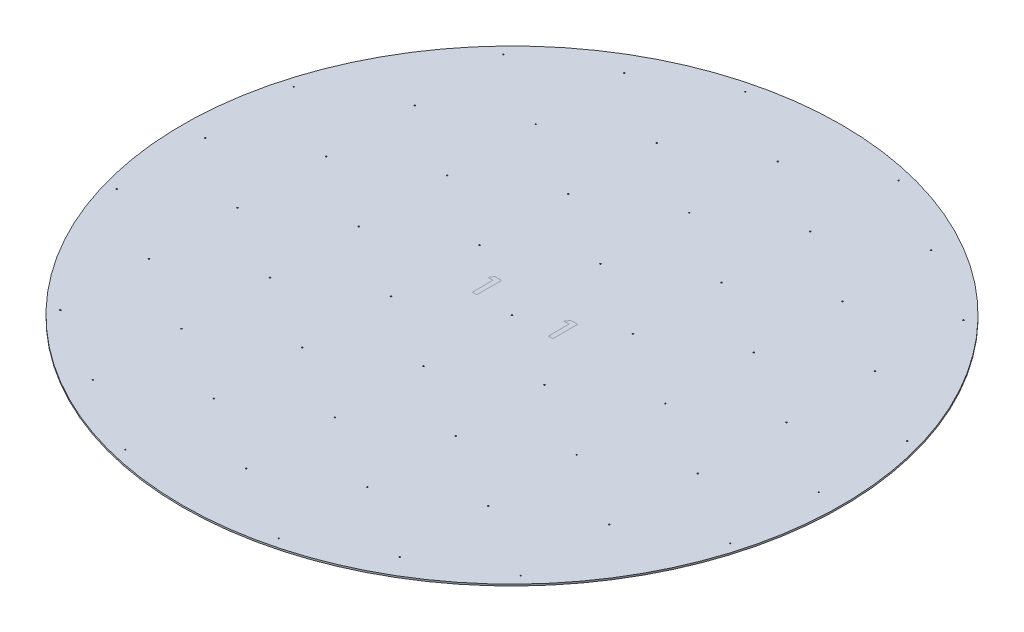
SolidWorks part; units mm, degrees
ref_plane "Front Plane" through (0, 0, 0) normal (0, 0, 1) x (1, 0, 0)
ref_plane "Top Plane" through (0, 0, 0) normal (0, 1, 0) x (1, 0, 0)
ref_plane "Right Plane" through (0, 0, 0) normal (1, 0, 0) x (0, 0, -1)
sketch "Sketch2" plane through (0, 0, 0) normal (0, 1, 0) x (1, 0, 0)
  circle A0 centre (0, 0) radius 40
  dimension "D1" = 80
extrude "Boss-Extrude1" add sketch "Sketch2" along normal blind 0.2
sketch "formula" plane through (0, 0.2, 0) normal (0, 1, 0) x (1, 0, 0)
  line L0 (0, 0) -> (0, 10.75) construction
  line L2 (46.374, 0) -> (0, 0) construction
  line L3 (9.3098, 5.375) -> (0, 0) construction
  line L4 (9.3098, 5.375) -> (0, 10.75) construction
  circle A16 centre (0, 10.75) radius 0.075
  circle A51 centre (9.3098, 16.125) radius 0.075
  circle A52 centre (0, 21.5) radius 0.075
  circle A53 centre (9.3098, 26.875) radius 0.075
  circle A54 centre (0, 32.25) radius 0.075
  circle A55 centre (9.3098, 37.625) radius 0.075
  circle A66 centre (0, 0) radius 0.075
  circle A67 centre (9.3098, 5.375) radius 0.075
  dimension "D2" = 0.15
  dimension "D3" = 10.75
sketch "Sketch4" plane through (0, 0.2, 0) normal (0, 1, 0) x (1, 0, 0)
  circle A1 centre (37.24, -10.75) radius 0.075
  circle A3 centre (18.62, -32.25) radius 0.075
  circle A5 centre (18.62, -10.75) radius 0.075
  circle A7 centre (27.9298, -16.125) radius 0.075
  circle A9 centre (18.62, -21.5) radius 0.075
  circle A11 centre (27.9298, -26.875) radius 0.075
  circle A13 centre (9.3098, -37.625) radius 0.075
  circle A15 centre (9.3098, -16.125) radius 0.075
  circle A17 centre (9.3098, -26.875) radius 0.075
  circle A19 centre (9.3098, -5.375) radius 0.075
  circle A21 centre (27.9298, -5.375) radius 0.075
  circle A23 centre (37.24, -10.75) radius 0.075
  circle A25 centre (18.62, -32.25) radius 0.075
  circle A27 centre (18.62, -10.75) radius 0.075
  circle A29 centre (27.9298, -16.125) radius 0.075
  circle A31 centre (18.62, -21.5) radius 0.075
  circle A33 centre (27.9298, -26.875) radius 0.075
  circle A35 centre (0, -32.25) radius 0.075
  circle A37 centre (9.3098, -37.625) radius 0.075
  circle A39 centre (0, -10.75) radius 0.075
  circle A41 centre (9.3098, -16.125) radius 0.075
  circle A43 centre (0, -21.5) radius 0.075
  circle A45 centre (9.3098, -26.875) radius 0.075
  circle A47 centre (9.3098, -5.375) radius 0.075
  circle A49 centre (27.9298, -5.375) radius 0.075
  circle A51 centre (-37.24, 10.75) radius 0.075
  circle A53 centre (-18.62, 32.25) radius 0.075
  circle A55 centre (-18.62, 10.75) radius 0.075
  circle A57 centre (-27.9298, 16.125) radius 0.075
  circle A59 centre (-18.62, 21.5) radius 0.075
  circle A61 centre (-27.9298, 26.875) radius 0.075
  circle A63 centre (-9.3098, 37.625) radius 0.075
  circle A65 centre (-9.3098, 16.125) radius 0.075
  circle A67 centre (-9.3098, 26.875) radius 0.075
  circle A69 centre (-9.3098, 5.375) radius 0.075
  circle A71 centre (-27.9298, 5.375) radius 0.075
  circle A73 centre (-37.24, 10.75) radius 0.075
  circle A75 centre (-37.24, 0) radius 0.075
  circle A77 centre (-18.62, 32.25) radius 0.075
  circle A79 centre (-18.62, 10.75) radius 0.075
  circle A81 centre (-27.9298, 16.125) radius 0.075
  circle A83 centre (-18.62, 21.5) radius 0.075
  circle A85 centre (-27.9298, 26.875) radius 0.075
  circle A87 centre (-18.62, 0) radius 0.075
  circle A89 centre (-9.3098, 37.625) radius 0.075
  circle A91 centre (-9.3098, 16.125) radius 0.075
  circle A93 centre (-9.3098, 26.875) radius 0.075
  circle A95 centre (-9.3098, 5.375) radius 0.075
  circle A97 centre (-27.9298, 5.375) radius 0.075
  circle A99 centre (-27.9298, -5.375) radius 0.075
  circle A101 centre (-9.3098, -5.375) radius 0.075
  circle A103 centre (-9.3098, -26.875) radius 0.075
  circle A105 centre (-9.3098, -16.125) radius 0.075
  circle A107 centre (-9.3098, -37.625) radius 0.075
  circle A109 centre (-27.9298, -26.875) radius 0.075
  circle A111 centre (-18.62, -21.5) radius 0.075
  circle A113 centre (-27.9298, -16.125) radius 0.075
  circle A115 centre (-18.62, -10.75) radius 0.075
  circle A117 centre (-18.62, -32.25) radius 0.075
  circle A119 centre (-37.24, -10.75) radius 0.075
  circle A121 centre (-27.9298, -5.375) radius 0.075
  circle A123 centre (-9.3098, -5.375) radius 0.075
  circle A125 centre (-9.3098, -26.875) radius 0.075
  circle A127 centre (-9.3098, -16.125) radius 0.075
  circle A129 centre (-9.3098, -37.625) radius 0.075
  circle A131 centre (-27.9298, -26.875) radius 0.075
  circle A133 centre (-18.62, -21.5) radius 0.075
  circle A135 centre (-27.9298, -16.125) radius 0.075
  circle A137 centre (-18.62, -10.75) radius 0.075
  circle A139 centre (-18.62, -32.25) radius 0.075
  circle A141 centre (-37.24, -10.75) radius 0.075
  circle A3000 centre (27.9298, 5.375) radius 0.075
  circle A3219 centre (9.3098, 5.375) radius 0.075
  circle A3220 centre (9.3098, 5.375) radius 0.075
  circle A3221 centre (0, 0) radius 0.075
  circle A3222 centre (0, 0) radius 0.075
  circle A3223 centre (9.3098, 26.875) radius 0.075
  circle A3224 centre (9.3098, 26.875) radius 0.075
  circle A3225 centre (0, 21.5) radius 0.075
  circle A3226 centre (0, 21.5) radius 0.075
  circle A3227 centre (9.3098, 16.125) radius 0.075
  circle A3228 centre (9.3098, 16.125) radius 0.075
  circle A3229 centre (0, 10.75) radius 0.075
  circle A3230 centre (0, 10.75) radius 0.075
  circle A3231 centre (9.3098, 37.625) radius 0.075
  circle A3232 centre (9.3098, 37.625) radius 0.075
  circle A3233 centre (0, 32.25) radius 0.075
  circle A3234 centre (0, 32.25) radius 0.075
  circle A3235 centre (18.62, 0) radius 0.075
  circle A3236 centre (27.9298, 26.875) radius 0.075
  circle A3237 centre (18.62, 21.5) radius 0.075
  circle A3238 centre (27.9298, 16.125) radius 0.075
  circle A3239 centre (18.62, 10.75) radius 0.075
  circle A3241 centre (18.62, 32.25) radius 0.075
  circle A3243 centre (37.24, 0) radius 0.075
  circle A3247 centre (37.24, 10.75) radius 0.075
  circle A3250 centre (27.9298, 37.625) radius 0.075
  circle A3251 centre (46.5498, 37.625) radius 0.075
  circle A3252 centre (37.24, 32.25) radius 0.075
  circle A3253 centre (46.5498, 26.875) radius 0.075
  circle A3254 centre (37.24, 21.5) radius 0.075
  circle A3255 centre (46.5498, 5.375) radius 0.075
  circle A3256 centre (46.5498, 16.125) radius 0.075
  circle A3271 centre (27.9298, 5.375) radius 0.075
  circle A3272 centre (9.3098, 5.375) radius 0.075
  circle A3273 centre (9.3098, 26.875) radius 0.075
  circle A3274 centre (9.3098, 16.125) radius 0.075
  circle A3275 centre (9.3098, 37.625) radius 0.075
  circle A3276 centre (27.9298, 26.875) radius 0.075
  circle A3277 centre (18.62, 21.5) radius 0.075
  circle A3278 centre (27.9298, 16.125) radius 0.075
  circle A3279 centre (18.62, 10.75) radius 0.075
  circle A3280 centre (18.62, 32.25) radius 0.075
  circle A3281 centre (37.24, 10.75) radius 0.075
  dimension "D121" = 0
  dimension "D122" = 0
  dimension "D123" = 0
  dimension "D124" = 0
  dimension "D125" = 0
  dimension "D126" = 0
  dimension "D127" = 0
  dimension "D128" = 0
  dimension "D129" = 3
extrude "Cut-Extrude2" cut sketch "Sketch4" against normal blind 0.2 contours A3222 | A3220 region at (0, 0.2, 0)
pattern_linear "LPattern1" count 4 spacing 10.75 along (0, 0, -1) count 3 spacing 18.6195 along (1, 0, 0) of "Cut-Extrude2"
mirror "Mirror1" about plane through (0, 0, 0) normal (1, 0, 0) of "LPattern1"
ref_plane "Plane1" through (0, 0, 0) normal (0, 0, -1) x (-1, 0, 0)
mirror "Mirror2" about plane through (0, 0, 0) normal (0, 0, -1) of "Mirror1", "LPattern1"
sketch "numbers" plane through (0, 0.2, 0) normal (0, 1, 0) x (1, 0, 0)
  line L0 (-7.0476, 0) -> (7.0476, 0) construction
  line L1 (46.374, 0) -> (0, 0) construction
  text T0 "<b>1      1</b>" font "Century Gothic" height 3
  point P6 (0, 0)
split "Split1" trim tools "numbers" bodies to split 160 resulting bodies 162 163 164
sketch "Sketch5" plane through (0, 0.2, 0) normal (0, 1, 0) x (1, 0, 0)
  circle A1 centre (40.7032, 13.5) radius 0.075
  circle A2 centre (40.7032, 13.5) radius 0.075
  circle A3 centre (39.8372, 15) radius 0.075
  circle A4 centre (39.8372, 15) radius 0.075
  circle A5 centre (39.8372, 14) radius 0.075
  circle A6 centre (39.8372, 14) radius 0.075
  circle A7 centre (40.7032, 14.5) radius 0.075
  circle A8 centre (40.7032, 14.5) radius 0.075
  circle A9 centre (39.8372, 10) radius 0.075
  circle A10 centre (39.8372, 10) radius 0.075
  circle A11 centre (39.8372, 11) radius 0.075
  circle A12 centre (39.8372, 11) radius 0.075
  circle A13 centre (39.8372, 10) radius 0.075
  circle A14 centre (39.8372, 10) radius 0.075
  circle A15 centre (40.7032, 10.5) radius 0.075
  circle A16 centre (40.7032, 10.5) radius 0.075
  circle A17 centre (38.9711, 8.5) radius 0.075
  circle A18 centre (38.9711, 8.5) radius 0.075
  circle A19 centre (38.1051, 9) radius 0.075
  circle A20 centre (38.1051, 9) radius 0.075
  circle A21 centre (38.9711, 9.5) radius 0.075
  circle A22 centre (38.9711, 9.5) radius 0.075
  circle A23 centre (38.1051, 5) radius 0.075
  circle A24 centre (38.1051, 5) radius 0.075
  circle A25 centre (38.1051, 6) radius 0.075
  circle A26 centre (38.1051, 6) radius 0.075
  circle A27 centre (38.1051, 5) radius 0.075
  circle A28 centre (38.1051, 5) radius 0.075
  circle A29 centre (38.9711, 5.5) radius 0.075
  circle A30 centre (38.9711, 5.5) radius 0.075
  circle A31 centre (38.1051, 7) radius 0.075
  circle A32 centre (38.1051, 7) radius 0.075
  circle A33 centre (36.3731, 4) radius 0.075
  circle A34 centre (36.3731, 4) radius 0.075
  circle A35 centre (37.2391, 4.5) radius 0.075
  circle A36 centre (37.2391, 4.5) radius 0.075
  circle A37 centre (36.3731, 0) radius 0.075
  circle A38 centre (36.3731, 0) radius 0.075
  circle A39 centre (37.2391, 0.5) radius 0.075
  circle A40 centre (37.2391, 0.5) radius 0.075
  circle A41 centre (36.3731, 1) radius 0.075
  circle A42 centre (36.3731, 1) radius 0.075
  circle A43 centre (36.3731, 2) radius 0.075
  circle A44 centre (36.3731, 2) radius 0.075
  circle A45 centre (36.3731, 1) radius 0.075
  circle A46 centre (36.3731, 1) radius 0.075
  circle A47 centre (37.2391, 1.5) radius 0.075
  circle A48 centre (37.2391, 1.5) radius 0.075
  circle A71 centre (31.1769, 29) radius 0.075
  circle A72 centre (31.1769, 29) radius 0.075
  circle A73 centre (32.0429, 28.5) radius 0.075
  circle A74 centre (32.0429, 28.5) radius 0.075
  circle A75 centre (31.1769, 30) radius 0.075
  circle A76 centre (31.1769, 30) radius 0.075
  circle A77 centre (31.1769, 29) radius 0.075
  circle A78 centre (31.1769, 29) radius 0.075
  circle A79 centre (32.0429, 29.5) radius 0.075
  circle A80 centre (32.0429, 29.5) radius 0.075
  circle A81 centre (30.3109, 27.5) radius 0.075
  circle A82 centre (30.3109, 27.5) radius 0.075
  circle A83 centre (29.4449, 28) radius 0.075
  circle A84 centre (29.4449, 28) radius 0.075
  circle A85 centre (29.4449, 24) radius 0.075
  circle A86 centre (29.4449, 24) radius 0.075
  circle A87 centre (29.4449, 23) radius 0.075
  circle A88 centre (29.4449, 23) radius 0.075
  circle A89 centre (30.3109, 23.5) radius 0.075
  circle A90 centre (30.3109, 23.5) radius 0.075
  circle A91 centre (29.4449, 25) radius 0.075
  circle A92 centre (29.4449, 25) radius 0.075
  circle A93 centre (29.4449, 24) radius 0.075
  circle A94 centre (29.4449, 24) radius 0.075
  circle A95 centre (30.3109, 24.5) radius 0.075
  circle A96 centre (30.3109, 24.5) radius 0.075
  circle A97 centre (27.7128, 23) radius 0.075
  circle A98 centre (27.7128, 23) radius 0.075
  circle A99 centre (27.7128, 22) radius 0.075
  circle A100 centre (27.7128, 22) radius 0.075
  circle A101 centre (28.5788, 22.5) radius 0.075
  circle A102 centre (28.5788, 22.5) radius 0.075
  circle A103 centre (27.7128, 19) radius 0.075
  circle A104 centre (27.7128, 19) radius 0.075
  circle A105 centre (27.7128, 18) radius 0.075
  circle A106 centre (27.7128, 18) radius 0.075
  circle A107 centre (28.5788, 18.5) radius 0.075
  circle A108 centre (28.5788, 18.5) radius 0.075
  circle A109 centre (27.7128, 20) radius 0.075
  circle A110 centre (27.7128, 20) radius 0.075
  circle A111 centre (27.7128, 19) radius 0.075
  circle A112 centre (27.7128, 19) radius 0.075
  circle A113 centre (25.9808, 17) radius 0.075
  circle A114 centre (25.9808, 17) radius 0.075
  circle A115 centre (25.9808, 16) radius 0.075
  circle A116 centre (25.9808, 16) radius 0.075
  circle A117 centre (26.8468, 16.5) radius 0.075
  circle A118 centre (26.8468, 16.5) radius 0.075
  circle A119 centre (25.9808, 13) radius 0.075
  circle A120 centre (25.9808, 13) radius 0.075
  circle A121 centre (25.9808, 12) radius 0.075
  circle A122 centre (25.9808, 12) radius 0.075
  circle A123 centre (26.8468, 12.5) radius 0.075
  circle A124 centre (26.8468, 12.5) radius 0.075
  circle A125 centre (25.9808, 14) radius 0.075
  circle A126 centre (25.9808, 14) radius 0.075
  circle A127 centre (25.9808, 13) radius 0.075
  circle A128 centre (25.9808, 13) radius 0.075
  circle A129 centre (24.2487, 12) radius 0.075
  circle A130 centre (24.2487, 12) radius 0.075
  circle A131 centre (24.2487, 11) radius 0.075
  circle A132 centre (24.2487, 11) radius 0.075
  circle A133 centre (25.1147, 11.5) radius 0.075
  circle A134 centre (25.1147, 11.5) radius 0.075
  circle A135 centre (24.2487, 8) radius 0.075
  circle A136 centre (24.2487, 8) radius 0.075
  circle A137 centre (24.2487, 7) radius 0.075
  circle A138 centre (24.2487, 7) radius 0.075
  circle A139 centre (25.1147, 7.5) radius 0.075
  circle A140 centre (25.1147, 7.5) radius 0.075
  circle A141 centre (24.2487, 9) radius 0.075
  circle A142 centre (24.2487, 9) radius 0.075
  circle A143 centre (24.2487, 8) radius 0.075
  circle A144 centre (24.2487, 8) radius 0.075
  circle A145 centre (22.5167, 6) radius 0.075
  circle A146 centre (22.5167, 6) radius 0.075
  circle A147 centre (23.3827, 6.5) radius 0.075
  circle A148 centre (23.3827, 6.5) radius 0.075
  circle A149 centre (22.5167, 3) radius 0.075
  circle A150 centre (22.5167, 3) radius 0.075
  circle A151 centre (22.5167, 2) radius 0.075
  circle A152 centre (22.5167, 2) radius 0.075
  circle A153 centre (23.3827, 2.5) radius 0.075
  circle A154 centre (23.3827, 2.5) radius 0.075
  circle A155 centre (22.5167, 4) radius 0.075
  circle A156 centre (22.5167, 4) radius 0.075
  circle A157 centre (22.5167, 3) radius 0.075
  circle A158 centre (22.5167, 3) radius 0.075
  circle A159 centre (23.3827, 3.5) radius 0.075
  circle A160 centre (23.3827, 3.5) radius 0.075
  circle A177 centre (18.1865, 35.5) radius 0.075
  circle A178 centre (18.1865, 35.5) radius 0.075
  circle A179 centre (17.3205, 36) radius 0.075
  circle A180 centre (17.3205, 36) radius 0.075
  circle A181 centre (17.3205, 32) radius 0.075
  circle A182 centre (17.3205, 32) radius 0.075
  circle A183 centre (17.3205, 31) radius 0.075
  circle A184 centre (17.3205, 31) radius 0.075
  circle A185 centre (18.1865, 31.5) radius 0.075
  circle A186 centre (18.1865, 31.5) radius 0.075
  circle A187 centre (17.3205, 33) radius 0.075
  circle A188 centre (17.3205, 33) radius 0.075
  circle A189 centre (17.3205, 32) radius 0.075
  circle A190 centre (17.3205, 32) radius 0.075
  circle A191 centre (18.1865, 32.5) radius 0.075
  circle A192 centre (18.1865, 32.5) radius 0.075
  circle A193 centre (15.5885, 31) radius 0.075
  circle A194 centre (15.5885, 31) radius 0.075
  circle A195 centre (15.5885, 30) radius 0.075
  circle A196 centre (15.5885, 30) radius 0.075
  circle A197 centre (16.4545, 30.5) radius 0.075
  circle A198 centre (16.4545, 30.5) radius 0.075
  circle A199 centre (15.5885, 27) radius 0.075
  circle A200 centre (15.5885, 27) radius 0.075
  circle A201 centre (15.5885, 26) radius 0.075
  circle A202 centre (15.5885, 26) radius 0.075
  circle A203 centre (16.4545, 26.5) radius 0.075
  circle A204 centre (16.4545, 26.5) radius 0.075
  circle A205 centre (15.5885, 28) radius 0.075
  circle A206 centre (15.5885, 28) radius 0.075
  circle A207 centre (15.5885, 27) radius 0.075
  circle A208 centre (15.5885, 27) radius 0.075
  circle A209 centre (13.8564, 26) radius 0.075
  circle A210 centre (13.8564, 26) radius 0.075
  circle A211 centre (13.8564, 25) radius 0.075
  circle A212 centre (13.8564, 25) radius 0.075
  circle A213 centre (14.7224, 25.5) radius 0.075
  circle A214 centre (14.7224, 25.5) radius 0.075
  circle A215 centre (13.8564, 21) radius 0.075
  circle A216 centre (13.8564, 21) radius 0.075
  circle A217 centre (14.7224, 20.5) radius 0.075
  circle A218 centre (14.7224, 20.5) radius 0.075
  circle A219 centre (13.8564, 22) radius 0.075
  circle A220 centre (13.8564, 22) radius 0.075
  circle A221 centre (13.8564, 21) radius 0.075
  circle A222 centre (13.8564, 21) radius 0.075
  circle A223 centre (14.7224, 21.5) radius 0.075
  circle A224 centre (14.7224, 21.5) radius 0.075
  circle A225 centre (12.9904, 19.5) radius 0.075
  circle A226 centre (12.9904, 19.5) radius 0.075
  circle A227 centre (12.1244, 20) radius 0.075
  circle A228 centre (12.1244, 20) radius 0.075
  circle A229 centre (12.1244, 18) radius 0.075
  circle A230 centre (12.1244, 18) radius 0.075
  circle A231 centre (12.1244, 17) radius 0.075
  circle A232 centre (12.1244, 17) radius 0.075
  circle A233 centre (12.9904, 17.5) radius 0.075
  circle A234 centre (12.9904, 17.5) radius 0.075
  circle A235 centre (12.1244, 16) radius 0.075
  circle A236 centre (12.1244, 16) radius 0.075
  circle A237 centre (12.1244, 15) radius 0.075
  circle A238 centre (12.1244, 15) radius 0.075
  circle A239 centre (12.9904, 15.5) radius 0.075
  circle A240 centre (12.9904, 15.5) radius 0.075
  circle A241 centre (11.2583, 13.5) radius 0.075
  circle A242 centre (11.2583, 13.5) radius 0.075
  circle A243 centre (10.3923, 15) radius 0.075
  circle A244 centre (10.3923, 15) radius 0.075
  circle A245 centre (10.3923, 14) radius 0.075
  circle A246 centre (10.3923, 14) radius 0.075
  circle A247 centre (11.2583, 14.5) radius 0.075
  circle A248 centre (11.2583, 14.5) radius 0.075
  circle A249 centre (10.3923, 10) radius 0.075
  circle A250 centre (10.3923, 10) radius 0.075
  circle A251 centre (10.3923, 11) radius 0.075
  circle A252 centre (10.3923, 11) radius 0.075
  circle A253 centre (10.3923, 10) radius 0.075
  circle A254 centre (10.3923, 10) radius 0.075
  circle A255 centre (11.2583, 10.5) radius 0.075
  circle A256 centre (11.2583, 10.5) radius 0.075
  circle A257 centre (9.5263, 8.5) radius 0.075
  circle A258 centre (9.5263, 8.5) radius 0.075
  circle A259 centre (8.6603, 9) radius 0.075
  circle A260 centre (8.6603, 9) radius 0.075
  circle A261 centre (9.5263, 9.5) radius 0.075
  circle A262 centre (9.5263, 9.5) radius 0.075
  circle A263 centre (8.6603, 5) radius 0.075
  circle A264 centre (8.6603, 5) radius 0.075
  circle A265 centre (8.6603, 6) radius 0.075
  circle A266 centre (8.6603, 6) radius 0.075
  circle A267 centre (8.6603, 5) radius 0.075
  circle A268 centre (8.6603, 5) radius 0.075
  circle A269 centre (9.5263, 5.5) radius 0.075
  circle A270 centre (9.5263, 5.5) radius 0.075
  circle A271 centre (8.6603, 7) radius 0.075
  circle A272 centre (8.6603, 7) radius 0.075
  circle A273 centre (6.9282, 4) radius 0.075
  circle A274 centre (6.9282, 4) radius 0.075
  circle A275 centre (7.7942, 4.5) radius 0.075
  circle A276 centre (7.7942, 4.5) radius 0.075
  circle A277 centre (6.9282, 0) radius 0.075
  circle A278 centre (6.9282, 0) radius 0.075
  circle A279 centre (7.7942, 0.5) radius 0.075
  circle A280 centre (7.7942, 0.5) radius 0.075
  circle A281 centre (6.9282, 1) radius 0.075
  circle A282 centre (6.9282, 1) radius 0.075
  circle A283 centre (6.9282, 2) radius 0.075
  circle A284 centre (6.9282, 2) radius 0.075
  circle A285 centre (6.9282, 1) radius 0.075
  circle A286 centre (6.9282, 1) radius 0.075
  circle A287 centre (7.7942, 1.5) radius 0.075
  circle A288 centre (7.7942, 1.5) radius 0.075
  circle A289 centre (3.4641, 39) radius 0.075
  circle A290 centre (3.4641, 39) radius 0.075
  circle A291 centre (3.4641, 38) radius 0.075
  circle A292 centre (3.4641, 38) radius 0.075
  circle A293 centre (4.3301, 38.5) radius 0.075
  circle A294 centre (4.3301, 38.5) radius 0.075
  circle A295 centre (3.4641, 35) radius 0.075
  circle A296 centre (3.4641, 35) radius 0.075
  circle A297 centre (3.4641, 34) radius 0.075
  circle A298 centre (3.4641, 34) radius 0.075
  circle A299 centre (4.3301, 34.5) radius 0.075
  circle A300 centre (4.3301, 34.5) radius 0.075
  circle A301 centre (3.4641, 36) radius 0.075
  circle A302 centre (3.4641, 36) radius 0.075
  circle A303 centre (3.4641, 35) radius 0.075
  circle A304 centre (3.4641, 35) radius 0.075
  circle A305 centre (1.7321, 34) radius 0.075
  circle A306 centre (1.7321, 34) radius 0.075
  circle A307 centre (1.7321, 33) radius 0.075
  circle A308 centre (1.7321, 33) radius 0.075
  circle A309 centre (2.5981, 33.5) radius 0.075
  circle A310 centre (2.5981, 33.5) radius 0.075
  circle A311 centre (1.7321, 29) radius 0.075
  circle A312 centre (1.7321, 29) radius 0.075
  circle A313 centre (2.5981, 28.5) radius 0.075
  circle A314 centre (2.5981, 28.5) radius 0.075
  circle A315 centre (1.7321, 30) radius 0.075
  circle A316 centre (1.7321, 30) radius 0.075
  circle A317 centre (1.7321, 29) radius 0.075
  circle A318 centre (1.7321, 29) radius 0.075
  circle A319 centre (2.5981, 29.5) radius 0.075
  circle A320 centre (2.5981, 29.5) radius 0.075
  circle A321 centre (0.866, 28.5) radius 0.075
  circle A322 centre (0.866, 28.5) radius 0.075
  circle A323 centre (0, 30) radius 0.075
  circle A324 centre (0, 30) radius 0.075
  circle A325 centre (0, 29) radius 0.075
  circle A326 centre (0, 29) radius 0.075
  circle A327 centre (0.866, 29.5) radius 0.075
  circle A328 centre (0.866, 29.5) radius 0.075
  circle A329 centre (0, 31) radius 0.075
  circle A330 centre (0, 31) radius 0.075
  circle A331 centre (0.866, 1.5) radius 0.075
  circle A332 centre (0.866, 1.5) radius 0.075
  circle A335 centre (0, 39) radius 0.075
  circle A336 centre (0, 39) radius 0.075
  circle A337 centre (0.866, 39.5) radius 0.075
  circle A338 centre (0.866, 39.5) radius 0.075
  circle A339 centre (39.8372, 17) radius 0.075
  circle A340 centre (39.8372, 17) radius 0.075
  circle A341 centre (39.8372, 16) radius 0.075
  circle A342 centre (39.8372, 16) radius 0.075
  circle A343 centre (40.7032, 16.5) radius 0.075
  circle A344 centre (40.7032, 16.5) radius 0.075
  circle A345 centre (39.8372, 13) radius 0.075
  circle A346 centre (39.8372, 13) radius 0.075
  circle A347 centre (39.8372, 12) radius 0.075
  circle A348 centre (39.8372, 12) radius 0.075
  circle A349 centre (40.7032, 12.5) radius 0.075
  circle A350 centre (40.7032, 12.5) radius 0.075
  circle A351 centre (39.8372, 14) radius 0.075
  circle A352 centre (39.8372, 14) radius 0.075
  circle A353 centre (39.8372, 13) radius 0.075
  circle A354 centre (39.8372, 13) radius 0.075
  circle A355 centre (38.1051, 12) radius 0.075
  circle A356 centre (38.1051, 12) radius 0.075
  circle A357 centre (38.1051, 11) radius 0.075
  circle A358 centre (38.1051, 11) radius 0.075
  circle A359 centre (38.9711, 11.5) radius 0.075
  circle A360 centre (38.9711, 11.5) radius 0.075
  circle A361 centre (38.1051, 8) radius 0.075
  circle A362 centre (38.1051, 8) radius 0.075
  circle A363 centre (38.1051, 7) radius 0.075
  circle A364 centre (38.1051, 7) radius 0.075
  circle A365 centre (38.9711, 7.5) radius 0.075
  circle A366 centre (38.9711, 7.5) radius 0.075
  circle A367 centre (38.1051, 9) radius 0.075
  circle A368 centre (38.1051, 9) radius 0.075
  circle A369 centre (38.1051, 8) radius 0.075
  circle A370 centre (38.1051, 8) radius 0.075
  circle A371 centre (36.3731, 6) radius 0.075
  circle A372 centre (36.3731, 6) radius 0.075
  circle A373 centre (37.2391, 6.5) radius 0.075
  circle A374 centre (37.2391, 6.5) radius 0.075
  circle A375 centre (36.3731, 3) radius 0.075
  circle A376 centre (36.3731, 3) radius 0.075
  circle A377 centre (36.3731, 2) radius 0.075
  circle A378 centre (36.3731, 2) radius 0.075
  circle A379 centre (37.2391, 2.5) radius 0.075
  circle A380 centre (37.2391, 2.5) radius 0.075
  circle A381 centre (36.3731, 4) radius 0.075
  circle A382 centre (36.3731, 4) radius 0.075
  circle A383 centre (36.3731, 3) radius 0.075
  circle A384 centre (36.3731, 3) radius 0.075
  circle A385 centre (37.2391, 3.5) radius 0.075
  circle A386 centre (37.2391, 3.5) radius 0.075
  circle A407 centre (31.1769, 32) radius 0.075
  circle A408 centre (31.1769, 32) radius 0.075
  circle A409 centre (31.1769, 31) radius 0.075
  circle A410 centre (31.1769, 31) radius 0.075
  circle A411 centre (32.0429, 31.5) radius 0.075
  circle A412 centre (32.0429, 31.5) radius 0.075
  circle A415 centre (31.1769, 32) radius 0.075
  circle A416 centre (31.1769, 32) radius 0.075
  circle A417 centre (32.0429, 32.5) radius 0.075
  circle A418 centre (32.0429, 32.5) radius 0.075
  circle A419 centre (29.4449, 31) radius 0.075
  circle A420 centre (29.4449, 31) radius 0.075
  circle A421 centre (29.4449, 30) radius 0.075
  circle A422 centre (29.4449, 30) radius 0.075
  circle A423 centre (30.3109, 30.5) radius 0.075
  circle A424 centre (30.3109, 30.5) radius 0.075
  circle A425 centre (29.4449, 27) radius 0.075
  circle A426 centre (29.4449, 27) radius 0.075
  circle A427 centre (29.4449, 26) radius 0.075
  circle A428 centre (29.4449, 26) radius 0.075
  circle A429 centre (30.3109, 26.5) radius 0.075
  circle A430 centre (30.3109, 26.5) radius 0.075
  circle A431 centre (29.4449, 28) radius 0.075
  circle A432 centre (29.4449, 28) radius 0.075
  circle A433 centre (29.4449, 27) radius 0.075
  circle A434 centre (29.4449, 27) radius 0.075
  circle A435 centre (27.7128, 26) radius 0.075
  circle A436 centre (27.7128, 26) radius 0.075
  circle A437 centre (27.7128, 25) radius 0.075
  circle A438 centre (27.7128, 25) radius 0.075
  circle A439 centre (28.5788, 25.5) radius 0.075
  circle A440 centre (28.5788, 25.5) radius 0.075
  circle A441 centre (27.7128, 21) radius 0.075
  circle A442 centre (27.7128, 21) radius 0.075
  circle A443 centre (28.5788, 20.5) radius 0.075
  circle A444 centre (28.5788, 20.5) radius 0.075
  circle A445 centre (27.7128, 22) radius 0.075
  circle A446 centre (27.7128, 22) radius 0.075
  circle A447 centre (27.7128, 21) radius 0.075
  circle A448 centre (27.7128, 21) radius 0.075
  circle A449 centre (28.5788, 21.5) radius 0.075
  circle A450 centre (28.5788, 21.5) radius 0.075
  circle A451 centre (26.8468, 19.5) radius 0.075
  circle A452 centre (26.8468, 19.5) radius 0.075
  circle A453 centre (25.9808, 20) radius 0.075
  circle A454 centre (25.9808, 20) radius 0.075
  circle A455 centre (25.9808, 18) radius 0.075
  circle A456 centre (25.9808, 18) radius 0.075
  circle A457 centre (25.9808, 17) radius 0.075
  circle A458 centre (25.9808, 17) radius 0.075
  circle A459 centre (26.8468, 17.5) radius 0.075
  circle A460 centre (26.8468, 17.5) radius 0.075
  circle A461 centre (25.9808, 16) radius 0.075
  circle A462 centre (25.9808, 16) radius 0.075
  circle A463 centre (25.9808, 15) radius 0.075
  circle A464 centre (25.9808, 15) radius 0.075
  circle A465 centre (26.8468, 15.5) radius 0.075
  circle A466 centre (26.8468, 15.5) radius 0.075
  circle A467 centre (25.1147, 13.5) radius 0.075
  circle A468 centre (25.1147, 13.5) radius 0.075
  circle A469 centre (24.2487, 15) radius 0.075
  circle A470 centre (24.2487, 15) radius 0.075
  circle A471 centre (24.2487, 14) radius 0.075
  circle A472 centre (24.2487, 14) radius 0.075
  circle A473 centre (25.1147, 14.5) radius 0.075
  circle A474 centre (25.1147, 14.5) radius 0.075
  circle A475 centre (24.2487, 10) radius 0.075
  circle A476 centre (24.2487, 10) radius 0.075
  circle A477 centre (24.2487, 11) radius 0.075
  circle A478 centre (24.2487, 11) radius 0.075
  circle A479 centre (24.2487, 10) radius 0.075
  circle A480 centre (24.2487, 10) radius 0.075
  circle A481 centre (25.1147, 10.5) radius 0.075
  circle A482 centre (25.1147, 10.5) radius 0.075
  circle A483 centre (23.3827, 8.5) radius 0.075
  circle A484 centre (23.3827, 8.5) radius 0.075
  circle A485 centre (22.5167, 9) radius 0.075
  circle A486 centre (22.5167, 9) radius 0.075
  circle A487 centre (23.3827, 9.5) radius 0.075
  circle A488 centre (23.3827, 9.5) radius 0.075
  circle A489 centre (22.5167, 5) radius 0.075
  circle A490 centre (22.5167, 5) radius 0.075
  circle A491 centre (22.5167, 6) radius 0.075
  circle A492 centre (22.5167, 6) radius 0.075
  circle A493 centre (22.5167, 5) radius 0.075
  circle A494 centre (22.5167, 5) radius 0.075
  circle A495 centre (23.3827, 5.5) radius 0.075
  circle A496 centre (23.3827, 5.5) radius 0.075
  circle A497 centre (22.5167, 7) radius 0.075
  circle A498 centre (22.5167, 7) radius 0.075
  circle A499 centre (20.7846, 4) radius 0.075
  circle A500 centre (20.7846, 4) radius 0.075
  circle A501 centre (21.6506, 4.5) radius 0.075
  circle A502 centre (21.6506, 4.5) radius 0.075
  circle A503 centre (20.7846, 0) radius 0.075
  circle A504 centre (20.7846, 0) radius 0.075
  circle A505 centre (21.6506, 0.5) radius 0.075
  circle A506 centre (21.6506, 0.5) radius 0.075
  circle A507 centre (20.7846, 1) radius 0.075
  circle A508 centre (20.7846, 1) radius 0.075
  circle A509 centre (20.7846, 2) radius 0.075
  circle A510 centre (20.7846, 2) radius 0.075
  circle A511 centre (20.7846, 1) radius 0.075
  circle A512 centre (20.7846, 1) radius 0.075
  circle A513 centre (21.6506, 1.5) radius 0.075
  circle A514 centre (21.6506, 1.5) radius 0.075
  circle A515 centre (17.3205, 39) radius 0.075
  circle A516 centre (17.3205, 39) radius 0.075
  circle A517 centre (17.3205, 38) radius 0.075
  circle A518 centre (17.3205, 38) radius 0.075
  circle A521 centre (17.3205, 35) radius 0.075
  circle A522 centre (17.3205, 35) radius 0.075
  circle A523 centre (17.3205, 34) radius 0.075
  circle A524 centre (17.3205, 34) radius 0.075
  circle A525 centre (18.1865, 34.5) radius 0.075
  circle A526 centre (18.1865, 34.5) radius 0.075
  circle A527 centre (17.3205, 36) radius 0.075
  circle A528 centre (17.3205, 36) radius 0.075
  circle A529 centre (17.3205, 35) radius 0.075
  circle A530 centre (17.3205, 35) radius 0.075
  circle A531 centre (15.5885, 34) radius 0.075
  circle A532 centre (15.5885, 34) radius 0.075
  circle A533 centre (15.5885, 33) radius 0.075
  circle A534 centre (15.5885, 33) radius 0.075
  circle A535 centre (16.4545, 33.5) radius 0.075
  circle A536 centre (16.4545, 33.5) radius 0.075
  circle A537 centre (15.5885, 29) radius 0.075
  circle A538 centre (15.5885, 29) radius 0.075
  circle A539 centre (16.4545, 28.5) radius 0.075
  circle A540 centre (16.4545, 28.5) radius 0.075
  circle A541 centre (15.5885, 30) radius 0.075
  circle A542 centre (15.5885, 30) radius 0.075
  circle A543 centre (15.5885, 29) radius 0.075
  circle A544 centre (15.5885, 29) radius 0.075
  circle A545 centre (16.4545, 29.5) radius 0.075
  circle A546 centre (16.4545, 29.5) radius 0.075
  circle A547 centre (14.7224, 27.5) radius 0.075
  circle A548 centre (14.7224, 27.5) radius 0.075
  circle A549 centre (13.8564, 28) radius 0.075
  circle A550 centre (13.8564, 28) radius 0.075
  circle A551 centre (13.8564, 24) radius 0.075
  circle A552 centre (13.8564, 24) radius 0.075
  circle A553 centre (13.8564, 23) radius 0.075
  circle A554 centre (13.8564, 23) radius 0.075
  circle A555 centre (14.7224, 23.5) radius 0.075
  circle A556 centre (14.7224, 23.5) radius 0.075
  circle A557 centre (13.8564, 25) radius 0.075
  circle A558 centre (13.8564, 25) radius 0.075
  circle A559 centre (13.8564, 24) radius 0.075
  circle A560 centre (13.8564, 24) radius 0.075
  circle A561 centre (14.7224, 24.5) radius 0.075
  circle A562 centre (14.7224, 24.5) radius 0.075
  circle A563 centre (12.1244, 23) radius 0.075
  circle A564 centre (12.1244, 23) radius 0.075
  circle A565 centre (12.1244, 22) radius 0.075
  circle A566 centre (12.1244, 22) radius 0.075
  circle A567 centre (12.9904, 22.5) radius 0.075
  circle A568 centre (12.9904, 22.5) radius 0.075
  circle A569 centre (12.1244, 19) radius 0.075
  circle A570 centre (12.1244, 19) radius 0.075
  circle A571 centre (12.1244, 18) radius 0.075
  circle A572 centre (12.1244, 18) radius 0.075
  circle A573 centre (12.9904, 18.5) radius 0.075
  circle A574 centre (12.9904, 18.5) radius 0.075
  circle A575 centre (12.1244, 20) radius 0.075
  circle A576 centre (12.1244, 20) radius 0.075
  circle A577 centre (12.1244, 19) radius 0.075
  circle A578 centre (12.1244, 19) radius 0.075
  circle A579 centre (10.3923, 17) radius 0.075
  circle A580 centre (10.3923, 17) radius 0.075
  circle A581 centre (10.3923, 16) radius 0.075
  circle A582 centre (10.3923, 16) radius 0.075
  circle A583 centre (11.2583, 16.5) radius 0.075
  circle A584 centre (11.2583, 16.5) radius 0.075
  circle A585 centre (10.3923, 13) radius 0.075
  circle A586 centre (10.3923, 13) radius 0.075
  circle A587 centre (10.3923, 12) radius 0.075
  circle A588 centre (10.3923, 12) radius 0.075
  circle A589 centre (11.2583, 12.5) radius 0.075
  circle A590 centre (11.2583, 12.5) radius 0.075
  circle A591 centre (10.3923, 14) radius 0.075
  circle A592 centre (10.3923, 14) radius 0.075
  circle A593 centre (10.3923, 13) radius 0.075
  circle A594 centre (10.3923, 13) radius 0.075
  circle A595 centre (8.6603, 12) radius 0.075
  circle A596 centre (8.6603, 12) radius 0.075
  circle A597 centre (8.6603, 11) radius 0.075
  circle A598 centre (8.6603, 11) radius 0.075
  circle A599 centre (9.5263, 11.5) radius 0.075
  circle A600 centre (9.5263, 11.5) radius 0.075
  circle A601 centre (8.6603, 8) radius 0.075
  circle A602 centre (8.6603, 8) radius 0.075
  circle A603 centre (8.6603, 7) radius 0.075
  circle A604 centre (8.6603, 7) radius 0.075
  circle A605 centre (9.5263, 7.5) radius 0.075
  circle A606 centre (9.5263, 7.5) radius 0.075
  circle A607 centre (8.6603, 9) radius 0.075
  circle A608 centre (8.6603, 9) radius 0.075
  circle A609 centre (8.6603, 8) radius 0.075
  circle A610 centre (8.6603, 8) radius 0.075
  circle A611 centre (6.9282, 6) radius 0.075
  circle A612 centre (6.9282, 6) radius 0.075
  circle A613 centre (7.7942, 6.5) radius 0.075
  circle A614 centre (7.7942, 6.5) radius 0.075
  circle A615 centre (6.9282, 3) radius 0.075
  circle A616 centre (6.9282, 3) radius 0.075
  circle A617 centre (6.9282, 2) radius 0.075
  circle A618 centre (6.9282, 2) radius 0.075
  circle A619 centre (7.7942, 2.5) radius 0.075
  circle A620 centre (7.7942, 2.5) radius 0.075
  circle A621 centre (6.9282, 4) radius 0.075
  circle A622 centre (6.9282, 4) radius 0.075
  circle A623 centre (6.9282, 3) radius 0.075
  circle A624 centre (6.9282, 3) radius 0.075
  circle A625 centre (7.7942, 3.5) radius 0.075
  circle A626 centre (7.7942, 3.5) radius 0.075
  circle A629 centre (5.1962, 39) radius 0.075
  circle A630 centre (5.1962, 39) radius 0.075
  circle A633 centre (3.4641, 37) radius 0.075
  circle A634 centre (3.4641, 37) radius 0.075
  circle A635 centre (4.3301, 36.5) radius 0.075
  circle A636 centre (4.3301, 36.5) radius 0.075
  circle A637 centre (3.4641, 38) radius 0.075
  circle A638 centre (3.4641, 38) radius 0.075
  circle A639 centre (3.4641, 37) radius 0.075
  circle A640 centre (3.4641, 37) radius 0.075
  circle A641 centre (4.3301, 37.5) radius 0.075
  circle A642 centre (4.3301, 37.5) radius 0.075
  circle A643 centre (2.5981, 35.5) radius 0.075
  circle A644 centre (2.5981, 35.5) radius 0.075
  circle A645 centre (1.7321, 36) radius 0.075
  circle A646 centre (1.7321, 36) radius 0.075
  circle A647 centre (1.7321, 32) radius 0.075
  circle A648 centre (1.7321, 32) radius 0.075
  circle A649 centre (1.7321, 31) radius 0.075
  circle A650 centre (1.7321, 31) radius 0.075
  circle A651 centre (2.5981, 31.5) radius 0.075
  circle A652 centre (2.5981, 31.5) radius 0.075
  circle A653 centre (1.7321, 33) radius 0.075
  circle A654 centre (1.7321, 33) radius 0.075
  circle A655 centre (1.7321, 32) radius 0.075
  circle A656 centre (1.7321, 32) radius 0.075
  circle A657 centre (2.5981, 32.5) radius 0.075
  circle A658 centre (2.5981, 32.5) radius 0.075
  circle A659 centre (0.866, 32.5) radius 0.075
  circle A660 centre (0.866, 32.5) radius 0.075
  circle A661 centre (0, 34) radius 0.075
  circle A662 centre (0, 34) radius 0.075
  circle A663 centre (0, 33) radius 0.075
  circle A664 centre (0, 33) radius 0.075
  circle A665 centre (0.866, 33.5) radius 0.075
  circle A666 centre (0.866, 33.5) radius 0.075
  circle A667 centre (0, 29) radius 0.075
  circle A668 centre (0, 29) radius 0.075
  circle A669 centre (0.866, 4.5) radius 0.075
  circle A670 centre (0.866, 4.5) radius 0.075
  circle A671 centre (0, 0) radius 0.075
  circle A672 centre (0, 0) radius 0.075
  circle A673 centre (0.866, 0.5) radius 0.075
  circle A674 centre (0.866, 0.5) radius 0.075
  circle A675 centre (0, 1) radius 0.075
  circle A676 centre (0, 1) radius 0.075
  circle A677 centre (0, 2) radius 0.075
  circle A678 centre (0, 2) radius 0.075
  circle A679 centre (0, 1) radius 0.075
  circle A680 centre (0, 1) radius 0.075
  circle A681 centre (40.7032, 19.5) radius 0.075
  circle A682 centre (40.7032, 19.5) radius 0.075
  circle A683 centre (39.8372, 20) radius 0.075
  circle A684 centre (39.8372, 20) radius 0.075
  circle A685 centre (39.8372, 18) radius 0.075
  circle A686 centre (39.8372, 18) radius 0.075
  circle A687 centre (39.8372, 17) radius 0.075
  circle A688 centre (39.8372, 17) radius 0.075
  circle A689 centre (40.7032, 17.5) radius 0.075
  circle A690 centre (40.7032, 17.5) radius 0.075
  circle A691 centre (39.8372, 16) radius 0.075
  circle A692 centre (39.8372, 16) radius 0.075
  circle A693 centre (39.8372, 15) radius 0.075
  circle A694 centre (39.8372, 15) radius 0.075
  circle A695 centre (40.7032, 15.5) radius 0.075
  circle A696 centre (40.7032, 15.5) radius 0.075
  circle A697 centre (38.9711, 13.5) radius 0.075
  circle A698 centre (38.9711, 13.5) radius 0.075
  circle A699 centre (38.1051, 15) radius 0.075
  circle A700 centre (38.1051, 15) radius 0.075
  circle A701 centre (38.1051, 14) radius 0.075
  circle A702 centre (38.1051, 14) radius 0.075
  circle A703 centre (38.9711, 14.5) radius 0.075
  circle A704 centre (38.9711, 14.5) radius 0.075
  circle A705 centre (38.1051, 10) radius 0.075
  circle A706 centre (38.1051, 10) radius 0.075
  circle A707 centre (38.1051, 11) radius 0.075
  circle A708 centre (38.1051, 11) radius 0.075
  circle A709 centre (38.1051, 10) radius 0.075
  circle A710 centre (38.1051, 10) radius 0.075
  circle A711 centre (38.9711, 10.5) radius 0.075
  circle A712 centre (38.9711, 10.5) radius 0.075
  circle A713 centre (37.2391, 8.5) radius 0.075
  circle A714 centre (37.2391, 8.5) radius 0.075
  circle A715 centre (36.3731, 9) radius 0.075
  circle A716 centre (36.3731, 9) radius 0.075
  circle A717 centre (37.2391, 9.5) radius 0.075
  circle A718 centre (37.2391, 9.5) radius 0.075
  circle A719 centre (36.3731, 5) radius 0.075
  circle A720 centre (36.3731, 5) radius 0.075
  circle A721 centre (36.3731, 6) radius 0.075
  circle A722 centre (36.3731, 6) radius 0.075
  circle A723 centre (36.3731, 5) radius 0.075
  circle A724 centre (36.3731, 5) radius 0.075
  circle A725 centre (37.2391, 5.5) radius 0.075
  circle A726 centre (37.2391, 5.5) radius 0.075
  circle A727 centre (36.3731, 7) radius 0.075
  circle A728 centre (36.3731, 7) radius 0.075
  circle A729 centre (34.641, 4) radius 0.075
  circle A730 centre (34.641, 4) radius 0.075
  circle A731 centre (35.507, 4.5) radius 0.075
  circle A732 centre (35.507, 4.5) radius 0.075
  circle A733 centre (34.641, 0) radius 0.075
  circle A734 centre (34.641, 0) radius 0.075
  circle A735 centre (35.507, 0.5) radius 0.075
  circle A736 centre (35.507, 0.5) radius 0.075
  circle A737 centre (34.641, 1) radius 0.075
  circle A738 centre (34.641, 1) radius 0.075
  circle A739 centre (34.641, 2) radius 0.075
  circle A740 centre (34.641, 2) radius 0.075
  circle A741 centre (34.641, 1) radius 0.075
  circle A742 centre (34.641, 1) radius 0.075
  circle A743 centre (35.507, 1.5) radius 0.075
  circle A744 centre (35.507, 1.5) radius 0.075
  circle A767 centre (29.4449, 29) radius 0.075
  circle A768 centre (29.4449, 29) radius 0.075
  circle A769 centre (30.3109, 28.5) radius 0.075
  circle A770 centre (30.3109, 28.5) radius 0.075
  circle A771 centre (29.4449, 30) radius 0.075
  circle A772 centre (29.4449, 30) radius 0.075
  circle A773 centre (29.4449, 29) radius 0.075
  circle A774 centre (29.4449, 29) radius 0.075
  circle A775 centre (30.3109, 29.5) radius 0.075
  circle A776 centre (30.3109, 29.5) radius 0.075
  circle A777 centre (28.5788, 27.5) radius 0.075
  circle A778 centre (28.5788, 27.5) radius 0.075
  circle A779 centre (27.7128, 28) radius 0.075
  circle A780 centre (27.7128, 28) radius 0.075
  circle A781 centre (27.7128, 24) radius 0.075
  circle A782 centre (27.7128, 24) radius 0.075
  circle A783 centre (27.7128, 23) radius 0.075
  circle A784 centre (27.7128, 23) radius 0.075
  circle A785 centre (28.5788, 23.5) radius 0.075
  circle A786 centre (28.5788, 23.5) radius 0.075
  circle A787 centre (27.7128, 25) radius 0.075
  circle A788 centre (27.7128, 25) radius 0.075
  circle A789 centre (27.7128, 24) radius 0.075
  circle A790 centre (27.7128, 24) radius 0.075
  circle A791 centre (28.5788, 24.5) radius 0.075
  circle A792 centre (28.5788, 24.5) radius 0.075
  circle A793 centre (25.9808, 23) radius 0.075
  circle A794 centre (25.9808, 23) radius 0.075
  circle A795 centre (25.9808, 22) radius 0.075
  circle A796 centre (25.9808, 22) radius 0.075
  circle A797 centre (26.8468, 22.5) radius 0.075
  circle A798 centre (26.8468, 22.5) radius 0.075
  circle A799 centre (25.9808, 19) radius 0.075
  circle A800 centre (25.9808, 19) radius 0.075
  circle A801 centre (25.9808, 18) radius 0.075
  circle A802 centre (25.9808, 18) radius 0.075
  circle A803 centre (26.8468, 18.5) radius 0.075
  circle A804 centre (26.8468, 18.5) radius 0.075
  circle A805 centre (25.9808, 20) radius 0.075
  circle A806 centre (25.9808, 20) radius 0.075
  circle A807 centre (25.9808, 19) radius 0.075
  circle A808 centre (25.9808, 19) radius 0.075
  circle A809 centre (24.2487, 17) radius 0.075
  circle A810 centre (24.2487, 17) radius 0.075
  circle A811 centre (24.2487, 16) radius 0.075
  circle A812 centre (24.2487, 16) radius 0.075
  circle A813 centre (25.1147, 16.5) radius 0.075
  circle A814 centre (25.1147, 16.5) radius 0.075
  circle A815 centre (24.2487, 13) radius 0.075
  circle A816 centre (24.2487, 13) radius 0.075
  circle A817 centre (24.2487, 12) radius 0.075
  circle A818 centre (24.2487, 12) radius 0.075
  circle A819 centre (25.1147, 12.5) radius 0.075
  circle A820 centre (25.1147, 12.5) radius 0.075
  circle A821 centre (24.2487, 14) radius 0.075
  circle A822 centre (24.2487, 14) radius 0.075
  circle A823 centre (24.2487, 13) radius 0.075
  circle A824 centre (24.2487, 13) radius 0.075
  circle A825 centre (22.5167, 12) radius 0.075
  circle A826 centre (22.5167, 12) radius 0.075
  circle A827 centre (22.5167, 11) radius 0.075
  circle A828 centre (22.5167, 11) radius 0.075
  circle A829 centre (23.3827, 11.5) radius 0.075
  circle A830 centre (23.3827, 11.5) radius 0.075
  circle A831 centre (22.5167, 8) radius 0.075
  circle A832 centre (22.5167, 8) radius 0.075
  circle A833 centre (22.5167, 7) radius 0.075
  circle A834 centre (22.5167, 7) radius 0.075
  circle A835 centre (23.3827, 7.5) radius 0.075
  circle A836 centre (23.3827, 7.5) radius 0.075
  circle A837 centre (22.5167, 9) radius 0.075
  circle A838 centre (22.5167, 9) radius 0.075
  circle A839 centre (22.5167, 8) radius 0.075
  circle A840 centre (22.5167, 8) radius 0.075
  circle A841 centre (20.7846, 6) radius 0.075
  circle A842 centre (20.7846, 6) radius 0.075
  circle A843 centre (21.6506, 6.5) radius 0.075
  circle A844 centre (21.6506, 6.5) radius 0.075
  circle A845 centre (20.7846, 3) radius 0.075
  circle A846 centre (20.7846, 3) radius 0.075
  circle A847 centre (20.7846, 2) radius 0.075
  circle A848 centre (20.7846, 2) radius 0.075
  circle A849 centre (21.6506, 2.5) radius 0.075
  circle A850 centre (21.6506, 2.5) radius 0.075
  circle A851 centre (20.7846, 4) radius 0.075
  circle A852 centre (20.7846, 4) radius 0.075
  circle A853 centre (20.7846, 3) radius 0.075
  circle A854 centre (20.7846, 3) radius 0.075
  circle A855 centre (21.6506, 3.5) radius 0.075
  circle A856 centre (21.6506, 3.5) radius 0.075
  circle A863 centre (17.3205, 37) radius 0.075
  circle A864 centre (17.3205, 37) radius 0.075
  circle A867 centre (17.3205, 38) radius 0.075
  circle A868 centre (17.3205, 38) radius 0.075
  circle A869 centre (17.3205, 37) radius 0.075
  circle A870 centre (17.3205, 37) radius 0.075
  circle A873 centre (16.4545, 35.5) radius 0.075
  circle A874 centre (16.4545, 35.5) radius 0.075
  circle A875 centre (15.5885, 36) radius 0.075
  circle A876 centre (15.5885, 36) radius 0.075
  circle A877 centre (15.5885, 32) radius 0.075
  circle A878 centre (15.5885, 32) radius 0.075
  circle A879 centre (15.5885, 31) radius 0.075
  circle A880 centre (15.5885, 31) radius 0.075
  circle A881 centre (16.4545, 31.5) radius 0.075
  circle A882 centre (16.4545, 31.5) radius 0.075
  circle A883 centre (15.5885, 33) radius 0.075
  circle A884 centre (15.5885, 33) radius 0.075
  circle A885 centre (15.5885, 32) radius 0.075
  circle A886 centre (15.5885, 32) radius 0.075
  circle A887 centre (16.4545, 32.5) radius 0.075
  circle A888 centre (16.4545, 32.5) radius 0.075
  circle A889 centre (13.8564, 31) radius 0.075
  circle A890 centre (13.8564, 31) radius 0.075
  circle A891 centre (13.8564, 30) radius 0.075
  circle A892 centre (13.8564, 30) radius 0.075
  circle A893 centre (14.7224, 30.5) radius 0.075
  circle A894 centre (14.7224, 30.5) radius 0.075
  circle A895 centre (13.8564, 27) radius 0.075
  circle A896 centre (13.8564, 27) radius 0.075
  circle A897 centre (13.8564, 26) radius 0.075
  circle A898 centre (13.8564, 26) radius 0.075
  circle A899 centre (14.7224, 26.5) radius 0.075
  circle A900 centre (14.7224, 26.5) radius 0.075
  circle A901 centre (13.8564, 28) radius 0.075
  circle A902 centre (13.8564, 28) radius 0.075
  circle A903 centre (13.8564, 27) radius 0.075
  circle A904 centre (13.8564, 27) radius 0.075
  circle A905 centre (12.1244, 26) radius 0.075
  circle A906 centre (12.1244, 26) radius 0.075
  circle A907 centre (12.1244, 25) radius 0.075
  circle A908 centre (12.1244, 25) radius 0.075
  circle A909 centre (12.9904, 25.5) radius 0.075
  circle A910 centre (12.9904, 25.5) radius 0.075
  circle A911 centre (12.1244, 21) radius 0.075
  circle A912 centre (12.1244, 21) radius 0.075
  circle A913 centre (12.9904, 20.5) radius 0.075
  circle A914 centre (12.9904, 20.5) radius 0.075
  circle A915 centre (12.1244, 22) radius 0.075
  circle A916 centre (12.1244, 22) radius 0.075
  circle A917 centre (12.1244, 21) radius 0.075
  circle A918 centre (12.1244, 21) radius 0.075
  circle A919 centre (12.9904, 21.5) radius 0.075
  circle A920 centre (12.9904, 21.5) radius 0.075
  circle A921 centre (11.2583, 19.5) radius 0.075
  circle A922 centre (11.2583, 19.5) radius 0.075
  circle A923 centre (10.3923, 20) radius 0.075
  circle A924 centre (10.3923, 20) radius 0.075
  circle A925 centre (10.3923, 18) radius 0.075
  circle A926 centre (10.3923, 18) radius 0.075
  circle A927 centre (10.3923, 17) radius 0.075
  circle A928 centre (10.3923, 17) radius 0.075
  circle A929 centre (11.2583, 17.5) radius 0.075
  circle A930 centre (11.2583, 17.5) radius 0.075
  circle A931 centre (10.3923, 16) radius 0.075
  circle A932 centre (10.3923, 16) radius 0.075
  circle A933 centre (10.3923, 15) radius 0.075
  circle A934 centre (10.3923, 15) radius 0.075
  circle A935 centre (11.2583, 15.5) radius 0.075
  circle A936 centre (11.2583, 15.5) radius 0.075
  circle A937 centre (9.5263, 13.5) radius 0.075
  circle A938 centre (9.5263, 13.5) radius 0.075
  circle A939 centre (8.6603, 15) radius 0.075
  circle A940 centre (8.6603, 15) radius 0.075
  circle A941 centre (8.6603, 14) radius 0.075
  circle A942 centre (8.6603, 14) radius 0.075
  circle A943 centre (9.5263, 14.5) radius 0.075
  circle A944 centre (9.5263, 14.5) radius 0.075
  circle A945 centre (8.6603, 10) radius 0.075
  circle A946 centre (8.6603, 10) radius 0.075
  circle A947 centre (8.6603, 11) radius 0.075
  circle A948 centre (8.6603, 11) radius 0.075
  circle A949 centre (8.6603, 10) radius 0.075
  circle A950 centre (8.6603, 10) radius 0.075
  circle A951 centre (9.5263, 10.5) radius 0.075
  circle A952 centre (9.5263, 10.5) radius 0.075
  circle A953 centre (7.7942, 8.5) radius 0.075
  circle A954 centre (7.7942, 8.5) radius 0.075
  circle A955 centre (6.9282, 9) radius 0.075
  circle A956 centre (6.9282, 9) radius 0.075
  circle A957 centre (7.7942, 9.5) radius 0.075
  circle A958 centre (7.7942, 9.5) radius 0.075
  circle A959 centre (6.9282, 5) radius 0.075
  circle A960 centre (6.9282, 5) radius 0.075
  circle A961 centre (6.9282, 6) radius 0.075
  circle A962 centre (6.9282, 6) radius 0.075
  circle A963 centre (6.9282, 5) radius 0.075
  circle A964 centre (6.9282, 5) radius 0.075
  circle A965 centre (7.7942, 5.5) radius 0.075
  circle A966 centre (7.7942, 5.5) radius 0.075
  circle A967 centre (6.9282, 7) radius 0.075
  circle A968 centre (6.9282, 7) radius 0.075
  circle A969 centre (5.1962, 4) radius 0.075
  circle A970 centre (5.1962, 4) radius 0.075
  circle A971 centre (6.0622, 4.5) radius 0.075
  circle A972 centre (6.0622, 4.5) radius 0.075
  circle A973 centre (5.1962, 0) radius 0.075
  circle A974 centre (5.1962, 0) radius 0.075
  circle A975 centre (6.0622, 0.5) radius 0.075
  circle A976 centre (6.0622, 0.5) radius 0.075
  circle A977 centre (5.1962, 1) radius 0.075
  circle A978 centre (5.1962, 1) radius 0.075
  circle A979 centre (5.1962, 2) radius 0.075
  circle A980 centre (5.1962, 2) radius 0.075
  circle A981 centre (5.1962, 1) radius 0.075
  circle A982 centre (5.1962, 1) radius 0.075
  circle A983 centre (6.0622, 1.5) radius 0.075
  circle A984 centre (6.0622, 1.5) radius 0.075
  circle A985 centre (1.7321, 39) radius 0.075
  circle A986 centre (1.7321, 39) radius 0.075
  circle A987 centre (1.7321, 38) radius 0.075
  circle A988 centre (1.7321, 38) radius 0.075
  circle A989 centre (2.5981, 38.5) radius 0.075
  circle A990 centre (2.5981, 38.5) radius 0.075
  circle A991 centre (1.7321, 35) radius 0.075
  circle A992 centre (1.7321, 35) radius 0.075
  circle A993 centre (1.7321, 34) radius 0.075
  circle A994 centre (1.7321, 34) radius 0.075
  circle A995 centre (2.5981, 34.5) radius 0.075
  circle A996 centre (2.5981, 34.5) radius 0.075
  circle A997 centre (1.7321, 36) radius 0.075
  circle A998 centre (1.7321, 36) radius 0.075
  circle A999 centre (1.7321, 35) radius 0.075
  circle A1000 centre (1.7321, 35) radius 0.075
  circle A1001 centre (0, 36) radius 0.075
  circle A1002 centre (0, 36) radius 0.075
  circle A1003 centre (0, 32) radius 0.075
  circle A1004 centre (0, 32) radius 0.075
  circle A1005 centre (0, 31) radius 0.075
  circle A1006 centre (0, 31) radius 0.075
  circle A1007 centre (0.866, 31.5) radius 0.075
  circle A1008 centre (0.866, 31.5) radius 0.075
  circle A1009 centre (0, 33) radius 0.075
  circle A1010 centre (0, 33) radius 0.075
  circle A1011 centre (0, 32) radius 0.075
  circle A1012 centre (0, 32) radius 0.075
  circle A1013 centre (0.866, 2.5) radius 0.075
  circle A1014 centre (0.866, 2.5) radius 0.075
  circle A1015 centre (0, 4) radius 0.075
  circle A1016 centre (0, 4) radius 0.075
  circle A1017 centre (0, 3) radius 0.075
  circle A1018 centre (0, 3) radius 0.075
  circle A1019 centre (0.866, 3.5) radius 0.075
  circle A1020 centre (0.866, 3.5) radius 0.075
  circle A1021 centre (0, 4) radius 0.075
  circle A1022 centre (0, 4) radius 0.075
  circle A1023 centre (39.8372, 23) radius 0.075
  circle A1024 centre (39.8372, 23) radius 0.075
  circle A1025 centre (39.8372, 22) radius 0.075
  circle A1026 centre (39.8372, 22) radius 0.075
  circle A1027 centre (40.7032, 22.5) radius 0.075
  circle A1028 centre (40.7032, 22.5) radius 0.075
  circle A1029 centre (39.8372, 19) radius 0.075
  circle A1030 centre (39.8372, 19) radius 0.075
  circle A1031 centre (39.8372, 18) radius 0.075
  circle A1032 centre (39.8372, 18) radius 0.075
  circle A1033 centre (40.7032, 18.5) radius 0.075
  circle A1034 centre (40.7032, 18.5) radius 0.075
  circle A1035 centre (39.8372, 20) radius 0.075
  circle A1036 centre (39.8372, 20) radius 0.075
  circle A1037 centre (39.8372, 19) radius 0.075
  circle A1038 centre (39.8372, 19) radius 0.075
  circle A1039 centre (38.1051, 17) radius 0.075
  circle A1040 centre (38.1051, 17) radius 0.075
  circle A1041 centre (38.1051, 16) radius 0.075
  circle A1042 centre (38.1051, 16) radius 0.075
  circle A1043 centre (38.9711, 16.5) radius 0.075
  circle A1044 centre (38.9711, 16.5) radius 0.075
  circle A1045 centre (38.1051, 13) radius 0.075
  circle A1046 centre (38.1051, 13) radius 0.075
  circle A1047 centre (38.1051, 12) radius 0.075
  circle A1048 centre (38.1051, 12) radius 0.075
  circle A1049 centre (38.9711, 12.5) radius 0.075
  circle A1050 centre (38.9711, 12.5) radius 0.075
  circle A1051 centre (38.1051, 14) radius 0.075
  circle A1052 centre (38.1051, 14) radius 0.075
  circle A1053 centre (38.1051, 13) radius 0.075
  circle A1054 centre (38.1051, 13) radius 0.075
  circle A1055 centre (36.3731, 12) radius 0.075
  circle A1056 centre (36.3731, 12) radius 0.075
  circle A1057 centre (36.3731, 11) radius 0.075
  circle A1058 centre (36.3731, 11) radius 0.075
  circle A1059 centre (37.2391, 11.5) radius 0.075
  circle A1060 centre (37.2391, 11.5) radius 0.075
  circle A1061 centre (36.3731, 8) radius 0.075
  circle A1062 centre (36.3731, 8) radius 0.075
  circle A1063 centre (36.3731, 7) radius 0.075
  circle A1064 centre (36.3731, 7) radius 0.075
  circle A1065 centre (37.2391, 7.5) radius 0.075
  circle A1066 centre (37.2391, 7.5) radius 0.075
  circle A1067 centre (36.3731, 9) radius 0.075
  circle A1068 centre (36.3731, 9) radius 0.075
  circle A1069 centre (36.3731, 8) radius 0.075
  circle A1070 centre (36.3731, 8) radius 0.075
  circle A1071 centre (34.641, 6) radius 0.075
  circle A1072 centre (34.641, 6) radius 0.075
  circle A1073 centre (35.507, 6.5) radius 0.075
  circle A1074 centre (35.507, 6.5) radius 0.075
  circle A1075 centre (34.641, 3) radius 0.075
  circle A1076 centre (34.641, 3) radius 0.075
  circle A1077 centre (34.641, 2) radius 0.075
  circle A1078 centre (34.641, 2) radius 0.075
  circle A1079 centre (35.507, 2.5) radius 0.075
  circle A1080 centre (35.507, 2.5) radius 0.075
  circle A1081 centre (34.641, 4) radius 0.075
  circle A1082 centre (34.641, 4) radius 0.075
  circle A1083 centre (34.641, 3) radius 0.075
  circle A1084 centre (34.641, 3) radius 0.075
  circle A1085 centre (35.507, 3.5) radius 0.075
  circle A1086 centre (35.507, 3.5) radius 0.075
  circle A1107 centre (29.4449, 32) radius 0.075
  circle A1108 centre (29.4449, 32) radius 0.075
  circle A1109 centre (29.4449, 31) radius 0.075
  circle A1110 centre (29.4449, 31) radius 0.075
  circle A1111 centre (30.3109, 31.5) radius 0.075
  circle A1112 centre (30.3109, 31.5) radius 0.075
  circle A1115 centre (29.4449, 32) radius 0.075
  circle A1116 centre (29.4449, 32) radius 0.075
  circle A1117 centre (30.3109, 32.5) radius 0.075
  circle A1118 centre (30.3109, 32.5) radius 0.075
  circle A1119 centre (27.7128, 31) radius 0.075
  circle A1120 centre (27.7128, 31) radius 0.075
  circle A1121 centre (27.7128, 30) radius 0.075
  circle A1122 centre (27.7128, 30) radius 0.075
  circle A1123 centre (28.5788, 30.5) radius 0.075
  circle A1124 centre (28.5788, 30.5) radius 0.075
  circle A1125 centre (27.7128, 27) radius 0.075
  circle A1126 centre (27.7128, 27) radius 0.075
  circle A1127 centre (27.7128, 26) radius 0.075
  circle A1128 centre (27.7128, 26) radius 0.075
  circle A1129 centre (28.5788, 26.5) radius 0.075
  circle A1130 centre (28.5788, 26.5) radius 0.075
  circle A1131 centre (27.7128, 28) radius 0.075
  circle A1132 centre (27.7128, 28) radius 0.075
  circle A1133 centre (27.7128, 27) radius 0.075
  circle A1134 centre (27.7128, 27) radius 0.075
  circle A1135 centre (25.9808, 26) radius 0.075
  circle A1136 centre (25.9808, 26) radius 0.075
  circle A1137 centre (25.9808, 25) radius 0.075
  circle A1138 centre (25.9808, 25) radius 0.075
  circle A1139 centre (26.8468, 25.5) radius 0.075
  circle A1140 centre (26.8468, 25.5) radius 0.075
  circle A1141 centre (25.9808, 21) radius 0.075
  circle A1142 centre (25.9808, 21) radius 0.075
  circle A1143 centre (26.8468, 20.5) radius 0.075
  circle A1144 centre (26.8468, 20.5) radius 0.075
  circle A1145 centre (25.9808, 22) radius 0.075
  circle A1146 centre (25.9808, 22) radius 0.075
  circle A1147 centre (25.9808, 21) radius 0.075
  circle A1148 centre (25.9808, 21) radius 0.075
  circle A1149 centre (26.8468, 21.5) radius 0.075
  circle A1150 centre (26.8468, 21.5) radius 0.075
  circle A1151 centre (25.1147, 19.5) radius 0.075
  circle A1152 centre (25.1147, 19.5) radius 0.075
  circle A1153 centre (24.2487, 20) radius 0.075
  circle A1154 centre (24.2487, 20) radius 0.075
  circle A1155 centre (24.2487, 18) radius 0.075
  circle A1156 centre (24.2487, 18) radius 0.075
  circle A1157 centre (24.2487, 17) radius 0.075
  circle A1158 centre (24.2487, 17) radius 0.075
  circle A1159 centre (25.1147, 17.5) radius 0.075
  circle A1160 centre (25.1147, 17.5) radius 0.075
  circle A1161 centre (24.2487, 16) radius 0.075
  circle A1162 centre (24.2487, 16) radius 0.075
  circle A1163 centre (24.2487, 15) radius 0.075
  circle A1164 centre (24.2487, 15) radius 0.075
  circle A1165 centre (25.1147, 15.5) radius 0.075
  circle A1166 centre (25.1147, 15.5) radius 0.075
  circle A1167 centre (23.3827, 13.5) radius 0.075
  circle A1168 centre (23.3827, 13.5) radius 0.075
  circle A1169 centre (22.5167, 15) radius 0.075
  circle A1170 centre (22.5167, 15) radius 0.075
  circle A1171 centre (22.5167, 14) radius 0.075
  circle A1172 centre (22.5167, 14) radius 0.075
  circle A1173 centre (23.3827, 14.5) radius 0.075
  circle A1174 centre (23.3827, 14.5) radius 0.075
  circle A1175 centre (22.5167, 10) radius 0.075
  circle A1176 centre (22.5167, 10) radius 0.075
  circle A1177 centre (22.5167, 11) radius 0.075
  circle A1178 centre (22.5167, 11) radius 0.075
  circle A1179 centre (22.5167, 10) radius 0.075
  circle A1180 centre (22.5167, 10) radius 0.075
  circle A1181 centre (23.3827, 10.5) radius 0.075
  circle A1182 centre (23.3827, 10.5) radius 0.075
  circle A1183 centre (21.6506, 8.5) radius 0.075
  circle A1184 centre (21.6506, 8.5) radius 0.075
  circle A1185 centre (20.7846, 9) radius 0.075
  circle A1186 centre (20.7846, 9) radius 0.075
  circle A1187 centre (21.6506, 9.5) radius 0.075
  circle A1188 centre (21.6506, 9.5) radius 0.075
  circle A1189 centre (20.7846, 5) radius 0.075
  circle A1190 centre (20.7846, 5) radius 0.075
  circle A1191 centre (20.7846, 6) radius 0.075
  circle A1192 centre (20.7846, 6) radius 0.075
  circle A1193 centre (20.7846, 5) radius 0.075
  circle A1194 centre (20.7846, 5) radius 0.075
  circle A1195 centre (21.6506, 5.5) radius 0.075
  circle A1196 centre (21.6506, 5.5) radius 0.075
  circle A1197 centre (20.7846, 7) radius 0.075
  circle A1198 centre (20.7846, 7) radius 0.075
  circle A1199 centre (19.0526, 4) radius 0.075
  circle A1200 centre (19.0526, 4) radius 0.075
  circle A1201 centre (19.9186, 4.5) radius 0.075
  circle A1202 centre (19.9186, 4.5) radius 0.075
  circle A1203 centre (19.0526, 0) radius 0.075
  circle A1204 centre (19.0526, 0) radius 0.075
  circle A1205 centre (19.9186, 0.5) radius 0.075
  circle A1206 centre (19.9186, 0.5) radius 0.075
  circle A1207 centre (19.0526, 1) radius 0.075
  circle A1208 centre (19.0526, 1) radius 0.075
  circle A1209 centre (19.0526, 2) radius 0.075
  circle A1210 centre (19.0526, 2) radius 0.075
  circle A1211 centre (19.0526, 1) radius 0.075
  circle A1212 centre (19.0526, 1) radius 0.075
  circle A1213 centre (19.9186, 1.5) radius 0.075
  circle A1214 centre (19.9186, 1.5) radius 0.075
  circle A1215 centre (15.5885, 39) radius 0.075
  circle A1216 centre (15.5885, 39) radius 0.075
  circle A1217 centre (15.5885, 38) radius 0.075
  circle A1218 centre (15.5885, 38) radius 0.075
  circle A1219 centre (16.4545, 38.5) radius 0.075
  circle A1220 centre (16.4545, 38.5) radius 0.075
  circle A1221 centre (15.5885, 35) radius 0.075
  circle A1222 centre (15.5885, 35) radius 0.075
  circle A1223 centre (15.5885, 34) radius 0.075
  circle A1224 centre (15.5885, 34) radius 0.075
  circle A1225 centre (16.4545, 34.5) radius 0.075
  circle A1226 centre (16.4545, 34.5) radius 0.075
  circle A1227 centre (15.5885, 36) radius 0.075
  circle A1228 centre (15.5885, 36) radius 0.075
  circle A1229 centre (15.5885, 35) radius 0.075
  circle A1230 centre (15.5885, 35) radius 0.075
  circle A1231 centre (13.8564, 34) radius 0.075
  circle A1232 centre (13.8564, 34) radius 0.075
  circle A1233 centre (13.8564, 33) radius 0.075
  circle A1234 centre (13.8564, 33) radius 0.075
  circle A1235 centre (14.7224, 33.5) radius 0.075
  circle A1236 centre (14.7224, 33.5) radius 0.075
  circle A1237 centre (13.8564, 29) radius 0.075
  circle A1238 centre (13.8564, 29) radius 0.075
  circle A1239 centre (14.7224, 28.5) radius 0.075
  circle A1240 centre (14.7224, 28.5) radius 0.075
  circle A1241 centre (13.8564, 30) radius 0.075
  circle A1242 centre (13.8564, 30) radius 0.075
  circle A1243 centre (13.8564, 29) radius 0.075
  circle A1244 centre (13.8564, 29) radius 0.075
  circle A1245 centre (14.7224, 29.5) radius 0.075
  circle A1246 centre (14.7224, 29.5) radius 0.075
  circle A1247 centre (12.9904, 27.5) radius 0.075
  circle A1248 centre (12.9904, 27.5) radius 0.075
  circle A1249 centre (12.1244, 28) radius 0.075
  circle A1250 centre (12.1244, 28) radius 0.075
  circle A1251 centre (12.1244, 24) radius 0.075
  circle A1252 centre (12.1244, 24) radius 0.075
  circle A1253 centre (12.1244, 23) radius 0.075
  circle A1254 centre (12.1244, 23) radius 0.075
  circle A1255 centre (12.9904, 23.5) radius 0.075
  circle A1256 centre (12.9904, 23.5) radius 0.075
  circle A1257 centre (12.1244, 25) radius 0.075
  circle A1258 centre (12.1244, 25) radius 0.075
  circle A1259 centre (12.1244, 24) radius 0.075
  circle A1260 centre (12.1244, 24) radius 0.075
  circle A1261 centre (12.9904, 24.5) radius 0.075
  circle A1262 centre (12.9904, 24.5) radius 0.075
  circle A1263 centre (10.3923, 23) radius 0.075
  circle A1264 centre (10.3923, 23) radius 0.075
  circle A1265 centre (10.3923, 22) radius 0.075
  circle A1266 centre (10.3923, 22) radius 0.075
  circle A1267 centre (11.2583, 22.5) radius 0.075
  circle A1268 centre (11.2583, 22.5) radius 0.075
  circle A1269 centre (10.3923, 19) radius 0.075
  circle A1270 centre (10.3923, 19) radius 0.075
  circle A1271 centre (10.3923, 18) radius 0.075
  circle A1272 centre (10.3923, 18) radius 0.075
  circle A1273 centre (11.2583, 18.5) radius 0.075
  circle A1274 centre (11.2583, 18.5) radius 0.075
  circle A1275 centre (10.3923, 20) radius 0.075
  circle A1276 centre (10.3923, 20) radius 0.075
  circle A1277 centre (10.3923, 19) radius 0.075
  circle A1278 centre (10.3923, 19) radius 0.075
  circle A1279 centre (8.6603, 17) radius 0.075
  circle A1280 centre (8.6603, 17) radius 0.075
  circle A1281 centre (8.6603, 16) radius 0.075
  circle A1282 centre (8.6603, 16) radius 0.075
  circle A1283 centre (9.5263, 16.5) radius 0.075
  circle A1284 centre (9.5263, 16.5) radius 0.075
  circle A1285 centre (8.6603, 13) radius 0.075
  circle A1286 centre (8.6603, 13) radius 0.075
  circle A1287 centre (8.6603, 12) radius 0.075
  circle A1288 centre (8.6603, 12) radius 0.075
  circle A1289 centre (9.5263, 12.5) radius 0.075
  circle A1290 centre (9.5263, 12.5) radius 0.075
  circle A1291 centre (8.6603, 14) radius 0.075
  circle A1292 centre (8.6603, 14) radius 0.075
  circle A1293 centre (8.6603, 13) radius 0.075
  circle A1294 centre (8.6603, 13) radius 0.075
  circle A1295 centre (6.9282, 12) radius 0.075
  circle A1296 centre (6.9282, 12) radius 0.075
  circle A1297 centre (6.9282, 11) radius 0.075
  circle A1298 centre (6.9282, 11) radius 0.075
  circle A1299 centre (7.7942, 11.5) radius 0.075
  circle A1300 centre (7.7942, 11.5) radius 0.075
  circle A1301 centre (6.9282, 8) radius 0.075
  circle A1302 centre (6.9282, 8) radius 0.075
  circle A1303 centre (6.9282, 7) radius 0.075
  circle A1304 centre (6.9282, 7) radius 0.075
  circle A1305 centre (7.7942, 7.5) radius 0.075
  circle A1306 centre (7.7942, 7.5) radius 0.075
  circle A1307 centre (6.9282, 9) radius 0.075
  circle A1308 centre (6.9282, 9) radius 0.075
  circle A1309 centre (6.9282, 8) radius 0.075
  circle A1310 centre (6.9282, 8) radius 0.075
  circle A1311 centre (5.1962, 6) radius 0.075
  circle A1312 centre (5.1962, 6) radius 0.075
  circle A1313 centre (6.0622, 6.5) radius 0.075
  circle A1314 centre (6.0622, 6.5) radius 0.075
  circle A1315 centre (5.1962, 3) radius 0.075
  circle A1316 centre (5.1962, 3) radius 0.075
  circle A1317 centre (5.1962, 2) radius 0.075
  circle A1318 centre (5.1962, 2) radius 0.075
  circle A1319 centre (6.0622, 2.5) radius 0.075
  circle A1320 centre (6.0622, 2.5) radius 0.075
  circle A1321 centre (5.1962, 4) radius 0.075
  circle A1322 centre (5.1962, 4) radius 0.075
  circle A1323 centre (5.1962, 3) radius 0.075
  circle A1324 centre (5.1962, 3) radius 0.075
  circle A1325 centre (6.0622, 3.5) radius 0.075
  circle A1326 centre (6.0622, 3.5) radius 0.075
  circle A1329 centre (3.4641, 39) radius 0.075
  circle A1330 centre (3.4641, 39) radius 0.075
  circle A1331 centre (4.3301, 39.5) radius 0.075
  circle A1332 centre (4.3301, 39.5) radius 0.075
  circle A1333 centre (1.7321, 37) radius 0.075
  circle A1334 centre (1.7321, 37) radius 0.075
  circle A1335 centre (2.5981, 36.5) radius 0.075
  circle A1336 centre (2.5981, 36.5) radius 0.075
  circle A1337 centre (1.7321, 38) radius 0.075
  circle A1338 centre (1.7321, 38) radius 0.075
  circle A1339 centre (1.7321, 37) radius 0.075
  circle A1340 centre (1.7321, 37) radius 0.075
  circle A1341 centre (2.5981, 37.5) radius 0.075
  circle A1342 centre (2.5981, 37.5) radius 0.075
  circle A1343 centre (0, 34) radius 0.075
  circle A1344 centre (0, 34) radius 0.075
  circle A1345 centre (0.866, 34.5) radius 0.075
  circle A1346 centre (0.866, 34.5) radius 0.075
  circle A1347 centre (0, 36) radius 0.075
  circle A1348 centre (0, 36) radius 0.075
  circle A1349 centre (0, 35) radius 0.075
  circle A1350 centre (0, 35) radius 0.075
  circle A1351 centre (0.866, 35.5) radius 0.075
  circle A1352 centre (0.866, 35.5) radius 0.075
  circle A1353 centre (0, 7) radius 0.075
  circle A1354 centre (0, 7) radius 0.075
  circle A1355 centre (0, 6) radius 0.075
  circle A1356 centre (0, 6) radius 0.075
  circle A1357 centre (0.866, 6.5) radius 0.075
  circle A1358 centre (0.866, 6.5) radius 0.075
  circle A1359 centre (0, 3) radius 0.075
  circle A1360 centre (0, 3) radius 0.075
  circle A1361 centre (0, 2) radius 0.075
  circle A1362 centre (0, 2) radius 0.075
  circle A1363 centre (39.8372, 26) radius 0.075
  circle A1364 centre (39.8372, 26) radius 0.075
  circle A1365 centre (39.8372, 25) radius 0.075
  circle A1366 centre (39.8372, 25) radius 0.075
  circle A1367 centre (40.7032, 25.5) radius 0.075
  circle A1368 centre (40.7032, 25.5) radius 0.075
  circle A1369 centre (39.8372, 21) radius 0.075
  circle A1370 centre (39.8372, 21) radius 0.075
  circle A1371 centre (40.7032, 20.5) radius 0.075
  circle A1372 centre (40.7032, 20.5) radius 0.075
  circle A1373 centre (39.8372, 22) radius 0.075
  circle A1374 centre (39.8372, 22) radius 0.075
  circle A1375 centre (39.8372, 21) radius 0.075
  circle A1376 centre (39.8372, 21) radius 0.075
  circle A1377 centre (40.7032, 21.5) radius 0.075
  circle A1378 centre (40.7032, 21.5) radius 0.075
  circle A1379 centre (38.9711, 19.5) radius 0.075
  circle A1380 centre (38.9711, 19.5) radius 0.075
  circle A1381 centre (38.1051, 20) radius 0.075
  circle A1382 centre (38.1051, 20) radius 0.075
  circle A1383 centre (38.1051, 18) radius 0.075
  circle A1384 centre (38.1051, 18) radius 0.075
  circle A1385 centre (38.1051, 17) radius 0.075
  circle A1386 centre (38.1051, 17) radius 0.075
  circle A1387 centre (38.9711, 17.5) radius 0.075
  circle A1388 centre (38.9711, 17.5) radius 0.075
  circle A1389 centre (38.1051, 16) radius 0.075
  circle A1390 centre (38.1051, 16) radius 0.075
  circle A1391 centre (38.1051, 15) radius 0.075
  circle A1392 centre (38.1051, 15) radius 0.075
  circle A1393 centre (38.9711, 15.5) radius 0.075
  circle A1394 centre (38.9711, 15.5) radius 0.075
  circle A1395 centre (37.2391, 13.5) radius 0.075
  circle A1396 centre (37.2391, 13.5) radius 0.075
  circle A1397 centre (36.3731, 15) radius 0.075
  circle A1398 centre (36.3731, 15) radius 0.075
  circle A1399 centre (36.3731, 14) radius 0.075
  circle A1400 centre (36.3731, 14) radius 0.075
  circle A1401 centre (37.2391, 14.5) radius 0.075
  circle A1402 centre (37.2391, 14.5) radius 0.075
  circle A1403 centre (36.3731, 10) radius 0.075
  circle A1404 centre (36.3731, 10) radius 0.075
  circle A1405 centre (36.3731, 11) radius 0.075
  circle A1406 centre (36.3731, 11) radius 0.075
  circle A1407 centre (36.3731, 10) radius 0.075
  circle A1408 centre (36.3731, 10) radius 0.075
  circle A1409 centre (37.2391, 10.5) radius 0.075
  circle A1410 centre (37.2391, 10.5) radius 0.075
  circle A1411 centre (35.507, 8.5) radius 0.075
  circle A1412 centre (35.507, 8.5) radius 0.075
  circle A1413 centre (34.641, 9) radius 0.075
  circle A1414 centre (34.641, 9) radius 0.075
  circle A1415 centre (35.507, 9.5) radius 0.075
  circle A1416 centre (35.507, 9.5) radius 0.075
  circle A1417 centre (34.641, 5) radius 0.075
  circle A1418 centre (34.641, 5) radius 0.075
  circle A1419 centre (34.641, 6) radius 0.075
  circle A1420 centre (34.641, 6) radius 0.075
  circle A1421 centre (34.641, 5) radius 0.075
  circle A1422 centre (34.641, 5) radius 0.075
  circle A1423 centre (35.507, 5.5) radius 0.075
  circle A1424 centre (35.507, 5.5) radius 0.075
  circle A1425 centre (34.641, 7) radius 0.075
  circle A1426 centre (34.641, 7) radius 0.075
  circle A1427 centre (32.909, 4) radius 0.075
  circle A1428 centre (32.909, 4) radius 0.075
  circle A1429 centre (33.775, 4.5) radius 0.075
  circle A1430 centre (33.775, 4.5) radius 0.075
  circle A1431 centre (32.909, 0) radius 0.075
  circle A1432 centre (32.909, 0) radius 0.075
  circle A1433 centre (33.775, 0.5) radius 0.075
  circle A1434 centre (33.775, 0.5) radius 0.075
  circle A1435 centre (32.909, 1) radius 0.075
  circle A1436 centre (32.909, 1) radius 0.075
  circle A1437 centre (32.909, 2) radius 0.075
  circle A1438 centre (32.909, 2) radius 0.075
  circle A1439 centre (32.909, 1) radius 0.075
  circle A1440 centre (32.909, 1) radius 0.075
  circle A1441 centre (33.775, 1.5) radius 0.075
  circle A1442 centre (33.775, 1.5) radius 0.075
  circle A1459 centre (27.7128, 34) radius 0.075
  circle A1460 centre (27.7128, 34) radius 0.075
  circle A1461 centre (27.7128, 33) radius 0.075
  circle A1462 centre (27.7128, 33) radius 0.075
  circle A1465 centre (27.7128, 29) radius 0.075
  circle A1466 centre (27.7128, 29) radius 0.075
  circle A1467 centre (28.5788, 28.5) radius 0.075
  circle A1468 centre (28.5788, 28.5) radius 0.075
  circle A1469 centre (27.7128, 30) radius 0.075
  circle A1470 centre (27.7128, 30) radius 0.075
  circle A1471 centre (27.7128, 29) radius 0.075
  circle A1472 centre (27.7128, 29) radius 0.075
  circle A1473 centre (28.5788, 29.5) radius 0.075
  circle A1474 centre (28.5788, 29.5) radius 0.075
  circle A1475 centre (26.8468, 27.5) radius 0.075
  circle A1476 centre (26.8468, 27.5) radius 0.075
  circle A1477 centre (25.9808, 28) radius 0.075
  circle A1478 centre (25.9808, 28) radius 0.075
  circle A1479 centre (25.9808, 24) radius 0.075
  circle A1480 centre (25.9808, 24) radius 0.075
  circle A1481 centre (25.9808, 23) radius 0.075
  circle A1482 centre (25.9808, 23) radius 0.075
  circle A1483 centre (26.8468, 23.5) radius 0.075
  circle A1484 centre (26.8468, 23.5) radius 0.075
  circle A1485 centre (25.9808, 25) radius 0.075
  circle A1486 centre (25.9808, 25) radius 0.075
  circle A1487 centre (25.9808, 24) radius 0.075
  circle A1488 centre (25.9808, 24) radius 0.075
  circle A1489 centre (26.8468, 24.5) radius 0.075
  circle A1490 centre (26.8468, 24.5) radius 0.075
  circle A1491 centre (24.2487, 23) radius 0.075
  circle A1492 centre (24.2487, 23) radius 0.075
  circle A1493 centre (24.2487, 22) radius 0.075
  circle A1494 centre (24.2487, 22) radius 0.075
  circle A1495 centre (25.1147, 22.5) radius 0.075
  circle A1496 centre (25.1147, 22.5) radius 0.075
  circle A1497 centre (24.2487, 19) radius 0.075
  circle A1498 centre (24.2487, 19) radius 0.075
  circle A1499 centre (24.2487, 18) radius 0.075
  circle A1500 centre (24.2487, 18) radius 0.075
  circle A1501 centre (25.1147, 18.5) radius 0.075
  circle A1502 centre (25.1147, 18.5) radius 0.075
  circle A1503 centre (24.2487, 20) radius 0.075
  circle A1504 centre (24.2487, 20) radius 0.075
  circle A1505 centre (24.2487, 19) radius 0.075
  circle A1506 centre (24.2487, 19) radius 0.075
  circle A1507 centre (22.5167, 17) radius 0.075
  circle A1508 centre (22.5167, 17) radius 0.075
  circle A1509 centre (22.5167, 16) radius 0.075
  circle A1510 centre (22.5167, 16) radius 0.075
  circle A1511 centre (23.3827, 16.5) radius 0.075
  circle A1512 centre (23.3827, 16.5) radius 0.075
  circle A1513 centre (22.5167, 13) radius 0.075
  circle A1514 centre (22.5167, 13) radius 0.075
  circle A1515 centre (22.5167, 12) radius 0.075
  circle A1516 centre (22.5167, 12) radius 0.075
  circle A1517 centre (23.3827, 12.5) radius 0.075
  circle A1518 centre (23.3827, 12.5) radius 0.075
  circle A1519 centre (22.5167, 14) radius 0.075
  circle A1520 centre (22.5167, 14) radius 0.075
  circle A1521 centre (22.5167, 13) radius 0.075
  circle A1522 centre (22.5167, 13) radius 0.075
  circle A1523 centre (20.7846, 12) radius 0.075
  circle A1524 centre (20.7846, 12) radius 0.075
  circle A1525 centre (20.7846, 11) radius 0.075
  circle A1526 centre (20.7846, 11) radius 0.075
  circle A1527 centre (21.6506, 11.5) radius 0.075
  circle A1528 centre (21.6506, 11.5) radius 0.075
  circle A1529 centre (20.7846, 8) radius 0.075
  circle A1530 centre (20.7846, 8) radius 0.075
  circle A1531 centre (20.7846, 7) radius 0.075
  circle A1532 centre (20.7846, 7) radius 0.075
  circle A1533 centre (21.6506, 7.5) radius 0.075
  circle A1534 centre (21.6506, 7.5) radius 0.075
  circle A1535 centre (20.7846, 9) radius 0.075
  circle A1536 centre (20.7846, 9) radius 0.075
  circle A1537 centre (20.7846, 8) radius 0.075
  circle A1538 centre (20.7846, 8) radius 0.075
  circle A1539 centre (19.0526, 6) radius 0.075
  circle A1540 centre (19.0526, 6) radius 0.075
  circle A1541 centre (19.9186, 6.5) radius 0.075
  circle A1542 centre (19.9186, 6.5) radius 0.075
  circle A1543 centre (19.0526, 3) radius 0.075
  circle A1544 centre (19.0526, 3) radius 0.075
  circle A1545 centre (19.0526, 2) radius 0.075
  circle A1546 centre (19.0526, 2) radius 0.075
  circle A1547 centre (19.9186, 2.5) radius 0.075
  circle A1548 centre (19.9186, 2.5) radius 0.075
  circle A1549 centre (19.0526, 4) radius 0.075
  circle A1550 centre (19.0526, 4) radius 0.075
  circle A1551 centre (19.0526, 3) radius 0.075
  circle A1552 centre (19.0526, 3) radius 0.075
  circle A1553 centre (19.9186, 3.5) radius 0.075
  circle A1554 centre (19.9186, 3.5) radius 0.075
  circle A1555 centre (17.3205, 40) radius 0.075
  circle A1556 centre (17.3205, 40) radius 0.075
  circle A1557 centre (17.3205, 39) radius 0.075
  circle A1558 centre (17.3205, 39) radius 0.075
  circle A1561 centre (15.5885, 37) radius 0.075
  circle A1562 centre (15.5885, 37) radius 0.075
  circle A1563 centre (16.4545, 36.5) radius 0.075
  circle A1564 centre (16.4545, 36.5) radius 0.075
  circle A1565 centre (15.5885, 38) radius 0.075
  circle A1566 centre (15.5885, 38) radius 0.075
  circle A1567 centre (15.5885, 37) radius 0.075
  circle A1568 centre (15.5885, 37) radius 0.075
  circle A1569 centre (16.4545, 37.5) radius 0.075
  circle A1570 centre (16.4545, 37.5) radius 0.075
  circle A1571 centre (14.7224, 35.5) radius 0.075
  circle A1572 centre (14.7224, 35.5) radius 0.075
  circle A1573 centre (13.8564, 36) radius 0.075
  circle A1574 centre (13.8564, 36) radius 0.075
  circle A1575 centre (13.8564, 32) radius 0.075
  circle A1576 centre (13.8564, 32) radius 0.075
  circle A1577 centre (13.8564, 31) radius 0.075
  circle A1578 centre (13.8564, 31) radius 0.075
  circle A1579 centre (14.7224, 31.5) radius 0.075
  circle A1580 centre (14.7224, 31.5) radius 0.075
  circle A1581 centre (13.8564, 33) radius 0.075
  circle A1582 centre (13.8564, 33) radius 0.075
  circle A1583 centre (13.8564, 32) radius 0.075
  circle A1584 centre (13.8564, 32) radius 0.075
  circle A1585 centre (14.7224, 32.5) radius 0.075
  circle A1586 centre (14.7224, 32.5) radius 0.075
  circle A1587 centre (12.1244, 31) radius 0.075
  circle A1588 centre (12.1244, 31) radius 0.075
  circle A1589 centre (12.1244, 30) radius 0.075
  circle A1590 centre (12.1244, 30) radius 0.075
  circle A1591 centre (12.9904, 30.5) radius 0.075
  circle A1592 centre (12.9904, 30.5) radius 0.075
  circle A1593 centre (12.1244, 27) radius 0.075
  circle A1594 centre (12.1244, 27) radius 0.075
  circle A1595 centre (12.1244, 26) radius 0.075
  circle A1596 centre (12.1244, 26) radius 0.075
  circle A1597 centre (12.9904, 26.5) radius 0.075
  circle A1598 centre (12.9904, 26.5) radius 0.075
  circle A1599 centre (12.1244, 28) radius 0.075
  circle A1600 centre (12.1244, 28) radius 0.075
  circle A1601 centre (12.1244, 27) radius 0.075
  circle A1602 centre (12.1244, 27) radius 0.075
  circle A1603 centre (10.3923, 26) radius 0.075
  circle A1604 centre (10.3923, 26) radius 0.075
  circle A1605 centre (10.3923, 25) radius 0.075
  circle A1606 centre (10.3923, 25) radius 0.075
  circle A1607 centre (11.2583, 25.5) radius 0.075
  circle A1608 centre (11.2583, 25.5) radius 0.075
  circle A1609 centre (10.3923, 21) radius 0.075
  circle A1610 centre (10.3923, 21) radius 0.075
  circle A1611 centre (11.2583, 20.5) radius 0.075
  circle A1612 centre (11.2583, 20.5) radius 0.075
  circle A1613 centre (10.3923, 22) radius 0.075
  circle A1614 centre (10.3923, 22) radius 0.075
  circle A1615 centre (10.3923, 21) radius 0.075
  circle A1616 centre (10.3923, 21) radius 0.075
  circle A1617 centre (11.2583, 21.5) radius 0.075
  circle A1618 centre (11.2583, 21.5) radius 0.075
  circle A1619 centre (9.5263, 19.5) radius 0.075
  circle A1620 centre (9.5263, 19.5) radius 0.075
  circle A1621 centre (8.6603, 20) radius 0.075
  circle A1622 centre (8.6603, 20) radius 0.075
  circle A1623 centre (8.6603, 18) radius 0.075
  circle A1624 centre (8.6603, 18) radius 0.075
  circle A1625 centre (8.6603, 17) radius 0.075
  circle A1626 centre (8.6603, 17) radius 0.075
  circle A1627 centre (9.5263, 17.5) radius 0.075
  circle A1628 centre (9.5263, 17.5) radius 0.075
  circle A1629 centre (8.6603, 16) radius 0.075
  circle A1630 centre (8.6603, 16) radius 0.075
  circle A1631 centre (8.6603, 15) radius 0.075
  circle A1632 centre (8.6603, 15) radius 0.075
  circle A1633 centre (9.5263, 15.5) radius 0.075
  circle A1634 centre (9.5263, 15.5) radius 0.075
  circle A1635 centre (7.7942, 13.5) radius 0.075
  circle A1636 centre (7.7942, 13.5) radius 0.075
  circle A1637 centre (6.9282, 15) radius 0.075
  circle A1638 centre (6.9282, 15) radius 0.075
  circle A1639 centre (6.9282, 14) radius 0.075
  circle A1640 centre (6.9282, 14) radius 0.075
  circle A1641 centre (7.7942, 14.5) radius 0.075
  circle A1642 centre (7.7942, 14.5) radius 0.075
  circle A1643 centre (6.9282, 10) radius 0.075
  circle A1644 centre (6.9282, 10) radius 0.075
  circle A1645 centre (6.9282, 11) radius 0.075
  circle A1646 centre (6.9282, 11) radius 0.075
  circle A1647 centre (6.9282, 10) radius 0.075
  circle A1648 centre (6.9282, 10) radius 0.075
  circle A1649 centre (7.7942, 10.5) radius 0.075
  circle A1650 centre (7.7942, 10.5) radius 0.075
  circle A1651 centre (6.0622, 8.5) radius 0.075
  circle A1652 centre (6.0622, 8.5) radius 0.075
  circle A1653 centre (5.1962, 9) radius 0.075
  circle A1654 centre (5.1962, 9) radius 0.075
  circle A1655 centre (6.0622, 9.5) radius 0.075
  circle A1656 centre (6.0622, 9.5) radius 0.075
  circle A1657 centre (5.1962, 5) radius 0.075
  circle A1658 centre (5.1962, 5) radius 0.075
  circle A1659 centre (5.1962, 6) radius 0.075
  circle A1660 centre (5.1962, 6) radius 0.075
  circle A1661 centre (5.1962, 5) radius 0.075
  circle A1662 centre (5.1962, 5) radius 0.075
  circle A1663 centre (6.0622, 5.5) radius 0.075
  circle A1664 centre (6.0622, 5.5) radius 0.075
  circle A1665 centre (5.1962, 7) radius 0.075
  circle A1666 centre (5.1962, 7) radius 0.075
  circle A1667 centre (3.4641, 4) radius 0.075
  circle A1668 centre (3.4641, 4) radius 0.075
  circle A1669 centre (4.3301, 4.5) radius 0.075
  circle A1670 centre (4.3301, 4.5) radius 0.075
  circle A1671 centre (3.4641, 0) radius 0.075
  circle A1672 centre (3.4641, 0) radius 0.075
  circle A1673 centre (4.3301, 0.5) radius 0.075
  circle A1674 centre (4.3301, 0.5) radius 0.075
  circle A1675 centre (3.4641, 1) radius 0.075
  circle A1676 centre (3.4641, 1) radius 0.075
  circle A1677 centre (3.4641, 2) radius 0.075
  circle A1678 centre (3.4641, 2) radius 0.075
  circle A1679 centre (3.4641, 1) radius 0.075
  circle A1680 centre (3.4641, 1) radius 0.075
  circle A1681 centre (4.3301, 1.5) radius 0.075
  circle A1682 centre (4.3301, 1.5) radius 0.075
  circle A1683 centre (0.866, 37.5) radius 0.075
  circle A1684 centre (0.866, 37.5) radius 0.075
  circle A1685 centre (0, 39) radius 0.075
  circle A1686 centre (0, 39) radius 0.075
  circle A1687 centre (0, 38) radius 0.075
  circle A1688 centre (0, 38) radius 0.075
  circle A1689 centre (0.866, 38.5) radius 0.075
  circle A1690 centre (0.866, 38.5) radius 0.075
  circle A1691 centre (0, 35) radius 0.075
  circle A1692 centre (0, 35) radius 0.075
  circle A1693 centre (0, 9) radius 0.075
  circle A1694 centre (0, 9) radius 0.075
  circle A1695 centre (0.866, 9.5) radius 0.075
  circle A1696 centre (0.866, 9.5) radius 0.075
  circle A1697 centre (0, 5) radius 0.075
  circle A1698 centre (0, 5) radius 0.075
  circle A1699 centre (0, 6) radius 0.075
  circle A1700 centre (0, 6) radius 0.075
  circle A1701 centre (0, 5) radius 0.075
  circle A1702 centre (0, 5) radius 0.075
  circle A1703 centre (0.866, 5.5) radius 0.075
  circle A1704 centre (0.866, 5.5) radius 0.075
  circle A1705 centre (40.7032, 27.5) radius 0.075
  circle A1706 centre (40.7032, 27.5) radius 0.075
  circle A1707 centre (39.8372, 28) radius 0.075
  circle A1708 centre (39.8372, 28) radius 0.075
  circle A1709 centre (39.8372, 24) radius 0.075
  circle A1710 centre (39.8372, 24) radius 0.075
  circle A1711 centre (39.8372, 23) radius 0.075
  circle A1712 centre (39.8372, 23) radius 0.075
  circle A1713 centre (40.7032, 23.5) radius 0.075
  circle A1714 centre (40.7032, 23.5) radius 0.075
  circle A1715 centre (39.8372, 25) radius 0.075
  circle A1716 centre (39.8372, 25) radius 0.075
  circle A1717 centre (39.8372, 24) radius 0.075
  circle A1718 centre (39.8372, 24) radius 0.075
  circle A1719 centre (40.7032, 24.5) radius 0.075
  circle A1720 centre (40.7032, 24.5) radius 0.075
  circle A1721 centre (38.1051, 23) radius 0.075
  circle A1722 centre (38.1051, 23) radius 0.075
  circle A1723 centre (38.1051, 22) radius 0.075
  circle A1724 centre (38.1051, 22) radius 0.075
  circle A1725 centre (38.9711, 22.5) radius 0.075
  circle A1726 centre (38.9711, 22.5) radius 0.075
  circle A1727 centre (38.1051, 19) radius 0.075
  circle A1728 centre (38.1051, 19) radius 0.075
  circle A1729 centre (38.1051, 18) radius 0.075
  circle A1730 centre (38.1051, 18) radius 0.075
  circle A1731 centre (38.9711, 18.5) radius 0.075
  circle A1732 centre (38.9711, 18.5) radius 0.075
  circle A1733 centre (38.1051, 20) radius 0.075
  circle A1734 centre (38.1051, 20) radius 0.075
  circle A1735 centre (38.1051, 19) radius 0.075
  circle A1736 centre (38.1051, 19) radius 0.075
  circle A1737 centre (36.3731, 17) radius 0.075
  circle A1738 centre (36.3731, 17) radius 0.075
  circle A1739 centre (36.3731, 16) radius 0.075
  circle A1740 centre (36.3731, 16) radius 0.075
  circle A1741 centre (37.2391, 16.5) radius 0.075
  circle A1742 centre (37.2391, 16.5) radius 0.075
  circle A1743 centre (36.3731, 13) radius 0.075
  circle A1744 centre (36.3731, 13) radius 0.075
  circle A1745 centre (36.3731, 12) radius 0.075
  circle A1746 centre (36.3731, 12) radius 0.075
  circle A1747 centre (37.2391, 12.5) radius 0.075
  circle A1748 centre (37.2391, 12.5) radius 0.075
  circle A1749 centre (36.3731, 14) radius 0.075
  circle A1750 centre (36.3731, 14) radius 0.075
  circle A1751 centre (36.3731, 13) radius 0.075
  circle A1752 centre (36.3731, 13) radius 0.075
  circle A1753 centre (34.641, 12) radius 0.075
  circle A1754 centre (34.641, 12) radius 0.075
  circle A1755 centre (34.641, 11) radius 0.075
  circle A1756 centre (34.641, 11) radius 0.075
  circle A1757 centre (35.507, 11.5) radius 0.075
  circle A1758 centre (35.507, 11.5) radius 0.075
  circle A1759 centre (34.641, 8) radius 0.075
  circle A1760 centre (34.641, 8) radius 0.075
  circle A1761 centre (34.641, 7) radius 0.075
  circle A1762 centre (34.641, 7) radius 0.075
  circle A1763 centre (35.507, 7.5) radius 0.075
  circle A1764 centre (35.507, 7.5) radius 0.075
  circle A1765 centre (34.641, 9) radius 0.075
  circle A1766 centre (34.641, 9) radius 0.075
  circle A1767 centre (34.641, 8) radius 0.075
  circle A1768 centre (34.641, 8) radius 0.075
  circle A1769 centre (32.909, 6) radius 0.075
  circle A1770 centre (32.909, 6) radius 0.075
  circle A1771 centre (33.775, 6.5) radius 0.075
  circle A1772 centre (33.775, 6.5) radius 0.075
  circle A1773 centre (32.909, 3) radius 0.075
  circle A1774 centre (32.909, 3) radius 0.075
  circle A1775 centre (32.909, 2) radius 0.075
  circle A1776 centre (32.909, 2) radius 0.075
  circle A1777 centre (33.775, 2.5) radius 0.075
  circle A1778 centre (33.775, 2.5) radius 0.075
  circle A1779 centre (32.909, 4) radius 0.075
  circle A1780 centre (32.909, 4) radius 0.075
  circle A1781 centre (32.909, 3) radius 0.075
  circle A1782 centre (32.909, 3) radius 0.075
  circle A1783 centre (33.775, 3.5) radius 0.075
  circle A1784 centre (33.775, 3.5) radius 0.075
  circle A1803 centre (27.7128, 36) radius 0.075
  circle A1804 centre (27.7128, 36) radius 0.075
  circle A1805 centre (27.7128, 32) radius 0.075
  circle A1806 centre (27.7128, 32) radius 0.075
  circle A1807 centre (27.7128, 31) radius 0.075
  circle A1808 centre (27.7128, 31) radius 0.075
  circle A1809 centre (28.5788, 31.5) radius 0.075
  circle A1810 centre (28.5788, 31.5) radius 0.075
  circle A1811 centre (27.7128, 33) radius 0.075
  circle A1812 centre (27.7128, 33) radius 0.075
  circle A1813 centre (27.7128, 32) radius 0.075
  circle A1814 centre (27.7128, 32) radius 0.075
  circle A1815 centre (28.5788, 32.5) radius 0.075
  circle A1816 centre (28.5788, 32.5) radius 0.075
  circle A1817 centre (25.9808, 31) radius 0.075
  circle A1818 centre (25.9808, 31) radius 0.075
  circle A1819 centre (25.9808, 30) radius 0.075
  circle A1820 centre (25.9808, 30) radius 0.075
  circle A1821 centre (26.8468, 30.5) radius 0.075
  circle A1822 centre (26.8468, 30.5) radius 0.075
  circle A1823 centre (25.9808, 27) radius 0.075
  circle A1824 centre (25.9808, 27) radius 0.075
  circle A1825 centre (25.9808, 26) radius 0.075
  circle A1826 centre (25.9808, 26) radius 0.075
  circle A1827 centre (26.8468, 26.5) radius 0.075
  circle A1828 centre (26.8468, 26.5) radius 0.075
  circle A1829 centre (25.9808, 28) radius 0.075
  circle A1830 centre (25.9808, 28) radius 0.075
  circle A1831 centre (25.9808, 27) radius 0.075
  circle A1832 centre (25.9808, 27) radius 0.075
  circle A1833 centre (24.2487, 26) radius 0.075
  circle A1834 centre (24.2487, 26) radius 0.075
  circle A1835 centre (24.2487, 25) radius 0.075
  circle A1836 centre (24.2487, 25) radius 0.075
  circle A1837 centre (25.1147, 25.5) radius 0.075
  circle A1838 centre (25.1147, 25.5) radius 0.075
  circle A1839 centre (24.2487, 21) radius 0.075
  circle A1840 centre (24.2487, 21) radius 0.075
  circle A1841 centre (25.1147, 20.5) radius 0.075
  circle A1842 centre (25.1147, 20.5) radius 0.075
  circle A1843 centre (24.2487, 22) radius 0.075
  circle A1844 centre (24.2487, 22) radius 0.075
  circle A1845 centre (24.2487, 21) radius 0.075
  circle A1846 centre (24.2487, 21) radius 0.075
  circle A1847 centre (25.1147, 21.5) radius 0.075
  circle A1848 centre (25.1147, 21.5) radius 0.075
  circle A1849 centre (23.3827, 19.5) radius 0.075
  circle A1850 centre (23.3827, 19.5) radius 0.075
  circle A1851 centre (22.5167, 20) radius 0.075
  circle A1852 centre (22.5167, 20) radius 0.075
  circle A1853 centre (22.5167, 18) radius 0.075
  circle A1854 centre (22.5167, 18) radius 0.075
  circle A1855 centre (22.5167, 17) radius 0.075
  circle A1856 centre (22.5167, 17) radius 0.075
  circle A1857 centre (23.3827, 17.5) radius 0.075
  circle A1858 centre (23.3827, 17.5) radius 0.075
  circle A1859 centre (22.5167, 16) radius 0.075
  circle A1860 centre (22.5167, 16) radius 0.075
  circle A1861 centre (22.5167, 15) radius 0.075
  circle A1862 centre (22.5167, 15) radius 0.075
  circle A1863 centre (23.3827, 15.5) radius 0.075
  circle A1864 centre (23.3827, 15.5) radius 0.075
  circle A1865 centre (21.6506, 13.5) radius 0.075
  circle A1866 centre (21.6506, 13.5) radius 0.075
  circle A1867 centre (20.7846, 15) radius 0.075
  circle A1868 centre (20.7846, 15) radius 0.075
  circle A1869 centre (20.7846, 14) radius 0.075
  circle A1870 centre (20.7846, 14) radius 0.075
  circle A1871 centre (21.6506, 14.5) radius 0.075
  circle A1872 centre (21.6506, 14.5) radius 0.075
  circle A1873 centre (20.7846, 10) radius 0.075
  circle A1874 centre (20.7846, 10) radius 0.075
  circle A1875 centre (20.7846, 11) radius 0.075
  circle A1876 centre (20.7846, 11) radius 0.075
  circle A1877 centre (20.7846, 10) radius 0.075
  circle A1878 centre (20.7846, 10) radius 0.075
  circle A1879 centre (21.6506, 10.5) radius 0.075
  circle A1880 centre (21.6506, 10.5) radius 0.075
  circle A1881 centre (19.9186, 8.5) radius 0.075
  circle A1882 centre (19.9186, 8.5) radius 0.075
  circle A1883 centre (19.0526, 9) radius 0.075
  circle A1884 centre (19.0526, 9) radius 0.075
  circle A1885 centre (19.9186, 9.5) radius 0.075
  circle A1886 centre (19.9186, 9.5) radius 0.075
  circle A1887 centre (19.0526, 5) radius 0.075
  circle A1888 centre (19.0526, 5) radius 0.075
  circle A1889 centre (19.0526, 6) radius 0.075
  circle A1890 centre (19.0526, 6) radius 0.075
  circle A1891 centre (19.0526, 5) radius 0.075
  circle A1892 centre (19.0526, 5) radius 0.075
  circle A1893 centre (19.9186, 5.5) radius 0.075
  circle A1894 centre (19.9186, 5.5) radius 0.075
  circle A1895 centre (19.0526, 7) radius 0.075
  circle A1896 centre (19.0526, 7) radius 0.075
  circle A1897 centre (17.3205, 4) radius 0.075
  circle A1898 centre (17.3205, 4) radius 0.075
  circle A1899 centre (18.1865, 4.5) radius 0.075
  circle A1900 centre (18.1865, 4.5) radius 0.075
  circle A1901 centre (17.3205, 0) radius 0.075
  circle A1902 centre (17.3205, 0) radius 0.075
  circle A1903 centre (18.1865, 0.5) radius 0.075
  circle A1904 centre (18.1865, 0.5) radius 0.075
  circle A1905 centre (17.3205, 1) radius 0.075
  circle A1906 centre (17.3205, 1) radius 0.075
  circle A1907 centre (17.3205, 2) radius 0.075
  circle A1908 centre (17.3205, 2) radius 0.075
  circle A1909 centre (17.3205, 1) radius 0.075
  circle A1910 centre (17.3205, 1) radius 0.075
  circle A1911 centre (18.1865, 1.5) radius 0.075
  circle A1912 centre (18.1865, 1.5) radius 0.075
  circle A1913 centre (13.8564, 39) radius 0.075
  circle A1914 centre (13.8564, 39) radius 0.075
  circle A1915 centre (13.8564, 38) radius 0.075
  circle A1916 centre (13.8564, 38) radius 0.075
  circle A1917 centre (14.7224, 38.5) radius 0.075
  circle A1918 centre (14.7224, 38.5) radius 0.075
  circle A1919 centre (13.8564, 35) radius 0.075
  circle A1920 centre (13.8564, 35) radius 0.075
  circle A1921 centre (13.8564, 34) radius 0.075
  circle A1922 centre (13.8564, 34) radius 0.075
  circle A1923 centre (14.7224, 34.5) radius 0.075
  circle A1924 centre (14.7224, 34.5) radius 0.075
  circle A1925 centre (13.8564, 36) radius 0.075
  circle A1926 centre (13.8564, 36) radius 0.075
  circle A1927 centre (13.8564, 35) radius 0.075
  circle A1928 centre (13.8564, 35) radius 0.075
  circle A1929 centre (12.1244, 34) radius 0.075
  circle A1930 centre (12.1244, 34) radius 0.075
  circle A1931 centre (12.1244, 33) radius 0.075
  circle A1932 centre (12.1244, 33) radius 0.075
  circle A1933 centre (12.9904, 33.5) radius 0.075
  circle A1934 centre (12.9904, 33.5) radius 0.075
  circle A1935 centre (12.1244, 29) radius 0.075
  circle A1936 centre (12.1244, 29) radius 0.075
  circle A1937 centre (12.9904, 28.5) radius 0.075
  circle A1938 centre (12.9904, 28.5) radius 0.075
  circle A1939 centre (12.1244, 30) radius 0.075
  circle A1940 centre (12.1244, 30) radius 0.075
  circle A1941 centre (12.1244, 29) radius 0.075
  circle A1942 centre (12.1244, 29) radius 0.075
  circle A1943 centre (12.9904, 29.5) radius 0.075
  circle A1944 centre (12.9904, 29.5) radius 0.075
  circle A1945 centre (11.2583, 27.5) radius 0.075
  circle A1946 centre (11.2583, 27.5) radius 0.075
  circle A1947 centre (10.3923, 28) radius 0.075
  circle A1948 centre (10.3923, 28) radius 0.075
  circle A1949 centre (10.3923, 24) radius 0.075
  circle A1950 centre (10.3923, 24) radius 0.075
  circle A1951 centre (10.3923, 23) radius 0.075
  circle A1952 centre (10.3923, 23) radius 0.075
  circle A1953 centre (11.2583, 23.5) radius 0.075
  circle A1954 centre (11.2583, 23.5) radius 0.075
  circle A1955 centre (10.3923, 25) radius 0.075
  circle A1956 centre (10.3923, 25) radius 0.075
  circle A1957 centre (10.3923, 24) radius 0.075
  circle A1958 centre (10.3923, 24) radius 0.075
  circle A1959 centre (11.2583, 24.5) radius 0.075
  circle A1960 centre (11.2583, 24.5) radius 0.075
  circle A1961 centre (8.6603, 23) radius 0.075
  circle A1962 centre (8.6603, 23) radius 0.075
  circle A1963 centre (8.6603, 22) radius 0.075
  circle A1964 centre (8.6603, 22) radius 0.075
  circle A1965 centre (9.5263, 22.5) radius 0.075
  circle A1966 centre (9.5263, 22.5) radius 0.075
  circle A1967 centre (8.6603, 19) radius 0.075
  circle A1968 centre (8.6603, 19) radius 0.075
  circle A1969 centre (8.6603, 18) radius 0.075
  circle A1970 centre (8.6603, 18) radius 0.075
  circle A1971 centre (9.5263, 18.5) radius 0.075
  circle A1972 centre (9.5263, 18.5) radius 0.075
  circle A1973 centre (8.6603, 20) radius 0.075
  circle A1974 centre (8.6603, 20) radius 0.075
  circle A1975 centre (8.6603, 19) radius 0.075
  circle A1976 centre (8.6603, 19) radius 0.075
  circle A1977 centre (6.9282, 17) radius 0.075
  circle A1978 centre (6.9282, 17) radius 0.075
  circle A1979 centre (6.9282, 16) radius 0.075
  circle A1980 centre (6.9282, 16) radius 0.075
  circle A1981 centre (7.7942, 16.5) radius 0.075
  circle A1982 centre (7.7942, 16.5) radius 0.075
  circle A1983 centre (6.9282, 13) radius 0.075
  circle A1984 centre (6.9282, 13) radius 0.075
  circle A1985 centre (6.9282, 12) radius 0.075
  circle A1986 centre (6.9282, 12) radius 0.075
  circle A1987 centre (7.7942, 12.5) radius 0.075
  circle A1988 centre (7.7942, 12.5) radius 0.075
  circle A1989 centre (6.9282, 14) radius 0.075
  circle A1990 centre (6.9282, 14) radius 0.075
  circle A1991 centre (6.9282, 13) radius 0.075
  circle A1992 centre (6.9282, 13) radius 0.075
  circle A1993 centre (5.1962, 12) radius 0.075
  circle A1994 centre (5.1962, 12) radius 0.075
  circle A1995 centre (5.1962, 11) radius 0.075
  circle A1996 centre (5.1962, 11) radius 0.075
  circle A1997 centre (6.0622, 11.5) radius 0.075
  circle A1998 centre (6.0622, 11.5) radius 0.075
  circle A1999 centre (5.1962, 8) radius 0.075
  circle A2000 centre (5.1962, 8) radius 0.075
  circle A2001 centre (5.1962, 7) radius 0.075
  circle A2002 centre (5.1962, 7) radius 0.075
  circle A2003 centre (6.0622, 7.5) radius 0.075
  circle A2004 centre (6.0622, 7.5) radius 0.075
  circle A2005 centre (5.1962, 9) radius 0.075
  circle A2006 centre (5.1962, 9) radius 0.075
  circle A2007 centre (5.1962, 8) radius 0.075
  circle A2008 centre (5.1962, 8) radius 0.075
  circle A2009 centre (3.4641, 6) radius 0.075
  circle A2010 centre (3.4641, 6) radius 0.075
  circle A2011 centre (4.3301, 6.5) radius 0.075
  circle A2012 centre (4.3301, 6.5) radius 0.075
  circle A2013 centre (3.4641, 3) radius 0.075
  circle A2014 centre (3.4641, 3) radius 0.075
  circle A2015 centre (3.4641, 2) radius 0.075
  circle A2016 centre (3.4641, 2) radius 0.075
  circle A2017 centre (4.3301, 2.5) radius 0.075
  circle A2018 centre (4.3301, 2.5) radius 0.075
  circle A2019 centre (3.4641, 4) radius 0.075
  circle A2020 centre (3.4641, 4) radius 0.075
  circle A2021 centre (3.4641, 3) radius 0.075
  circle A2022 centre (3.4641, 3) radius 0.075
  circle A2023 centre (4.3301, 3.5) radius 0.075
  circle A2024 centre (4.3301, 3.5) radius 0.075
  circle A2027 centre (1.7321, 39) radius 0.075
  circle A2028 centre (1.7321, 39) radius 0.075
  circle A2029 centre (0, 37) radius 0.075
  circle A2030 centre (0, 37) radius 0.075
  circle A2031 centre (0.866, 36.5) radius 0.075
  circle A2032 centre (0.866, 36.5) radius 0.075
  circle A2033 centre (0, 38) radius 0.075
  circle A2034 centre (0, 38) radius 0.075
  circle A2035 centre (0, 37) radius 0.075
  circle A2036 centre (0, 37) radius 0.075
  circle A2037 centre (0, 7) radius 0.075
  circle A2038 centre (0, 7) radius 0.075
  circle A2039 centre (0.866, 7.5) radius 0.075
  circle A2040 centre (0.866, 7.5) radius 0.075
  circle A2041 centre (0, 9) radius 0.075
  circle A2042 centre (0, 9) radius 0.075
  circle A2043 centre (0, 8) radius 0.075
  circle A2044 centre (0, 8) radius 0.075
  circle A2045 centre (0.866, 8.5) radius 0.075
  circle A2046 centre (0.866, 8.5) radius 0.075
  circle A2047 centre (2.5981, 39.5) radius 0.075
  circle A2048 centre (2.5981, 39.5) radius 0.075
  circle A2049 centre (39.8372, 31) radius 0.075
  circle A2050 centre (39.8372, 31) radius 0.075
  circle A2051 centre (39.8372, 30) radius 0.075
  circle A2052 centre (39.8372, 30) radius 0.075
  circle A2053 centre (40.7032, 30.5) radius 0.075
  circle A2054 centre (40.7032, 30.5) radius 0.075
  circle A2055 centre (39.8372, 27) radius 0.075
  circle A2056 centre (39.8372, 27) radius 0.075
  circle A2057 centre (39.8372, 26) radius 0.075
  circle A2058 centre (39.8372, 26) radius 0.075
  circle A2059 centre (40.7032, 26.5) radius 0.075
  circle A2060 centre (40.7032, 26.5) radius 0.075
  circle A2061 centre (39.8372, 28) radius 0.075
  circle A2062 centre (39.8372, 28) radius 0.075
  circle A2063 centre (39.8372, 27) radius 0.075
  circle A2064 centre (39.8372, 27) radius 0.075
  circle A2065 centre (38.1051, 26) radius 0.075
  circle A2066 centre (38.1051, 26) radius 0.075
  circle A2067 centre (38.1051, 25) radius 0.075
  circle A2068 centre (38.1051, 25) radius 0.075
  circle A2069 centre (38.9711, 25.5) radius 0.075
  circle A2070 centre (38.9711, 25.5) radius 0.075
  circle A2071 centre (38.1051, 21) radius 0.075
  circle A2072 centre (38.1051, 21) radius 0.075
  circle A2073 centre (38.9711, 20.5) radius 0.075
  circle A2074 centre (38.9711, 20.5) radius 0.075
  circle A2075 centre (38.1051, 22) radius 0.075
  circle A2076 centre (38.1051, 22) radius 0.075
  circle A2077 centre (38.1051, 21) radius 0.075
  circle A2078 centre (38.1051, 21) radius 0.075
  circle A2079 centre (38.9711, 21.5) radius 0.075
  circle A2080 centre (38.9711, 21.5) radius 0.075
  circle A2081 centre (37.2391, 19.5) radius 0.075
  circle A2082 centre (37.2391, 19.5) radius 0.075
  circle A2083 centre (36.3731, 20) radius 0.075
  circle A2084 centre (36.3731, 20) radius 0.075
  circle A2085 centre (36.3731, 18) radius 0.075
  circle A2086 centre (36.3731, 18) radius 0.075
  circle A2087 centre (36.3731, 17) radius 0.075
  circle A2088 centre (36.3731, 17) radius 0.075
  circle A2089 centre (37.2391, 17.5) radius 0.075
  circle A2090 centre (37.2391, 17.5) radius 0.075
  circle A2091 centre (36.3731, 16) radius 0.075
  circle A2092 centre (36.3731, 16) radius 0.075
  circle A2093 centre (36.3731, 15) radius 0.075
  circle A2094 centre (36.3731, 15) radius 0.075
  circle A2095 centre (37.2391, 15.5) radius 0.075
  circle A2096 centre (37.2391, 15.5) radius 0.075
  circle A2097 centre (35.507, 13.5) radius 0.075
  circle A2098 centre (35.507, 13.5) radius 0.075
  circle A2099 centre (34.641, 15) radius 0.075
  circle A2100 centre (34.641, 15) radius 0.075
  circle A2101 centre (34.641, 14) radius 0.075
  circle A2102 centre (34.641, 14) radius 0.075
  circle A2103 centre (35.507, 14.5) radius 0.075
  circle A2104 centre (35.507, 14.5) radius 0.075
  circle A2105 centre (34.641, 10) radius 0.075
  circle A2106 centre (34.641, 10) radius 0.075
  circle A2107 centre (34.641, 11) radius 0.075
  circle A2108 centre (34.641, 11) radius 0.075
  circle A2109 centre (34.641, 10) radius 0.075
  circle A2110 centre (34.641, 10) radius 0.075
  circle A2111 centre (35.507, 10.5) radius 0.075
  circle A2112 centre (35.507, 10.5) radius 0.075
  circle A2113 centre (33.775, 8.5) radius 0.075
  circle A2114 centre (33.775, 8.5) radius 0.075
  circle A2115 centre (32.909, 9) radius 0.075
  circle A2116 centre (32.909, 9) radius 0.075
  circle A2117 centre (33.775, 9.5) radius 0.075
  circle A2118 centre (33.775, 9.5) radius 0.075
  circle A2119 centre (32.909, 5) radius 0.075
  circle A2120 centre (32.909, 5) radius 0.075
  circle A2121 centre (32.909, 6) radius 0.075
  circle A2122 centre (32.909, 6) radius 0.075
  circle A2123 centre (32.909, 5) radius 0.075
  circle A2124 centre (32.909, 5) radius 0.075
  circle A2125 centre (33.775, 5.5) radius 0.075
  circle A2126 centre (33.775, 5.5) radius 0.075
  circle A2127 centre (32.909, 7) radius 0.075
  circle A2128 centre (32.909, 7) radius 0.075
  circle A2129 centre (31.1769, 4) radius 0.075
  circle A2130 centre (31.1769, 4) radius 0.075
  circle A2131 centre (32.0429, 4.5) radius 0.075
  circle A2132 centre (32.0429, 4.5) radius 0.075
  circle A2133 centre (31.1769, 0) radius 0.075
  circle A2134 centre (31.1769, 0) radius 0.075
  circle A2135 centre (32.0429, 0.5) radius 0.075
  circle A2136 centre (32.0429, 0.5) radius 0.075
  circle A2137 centre (31.1769, 1) radius 0.075
  circle A2138 centre (31.1769, 1) radius 0.075
  circle A2139 centre (31.1769, 2) radius 0.075
  circle A2140 centre (31.1769, 2) radius 0.075
  circle A2141 centre (31.1769, 1) radius 0.075
  circle A2142 centre (31.1769, 1) radius 0.075
  circle A2143 centre (32.0429, 1.5) radius 0.075
  circle A2144 centre (32.0429, 1.5) radius 0.075
  circle A2151 centre (27.7128, 35) radius 0.075
  circle A2152 centre (27.7128, 35) radius 0.075
  circle A2153 centre (27.7128, 34) radius 0.075
  circle A2154 centre (27.7128, 34) radius 0.075
  circle A2157 centre (27.7128, 36) radius 0.075
  circle A2158 centre (27.7128, 36) radius 0.075
  circle A2159 centre (27.7128, 35) radius 0.075
  circle A2160 centre (27.7128, 35) radius 0.075
  circle A2161 centre (25.9808, 34) radius 0.075
  circle A2162 centre (25.9808, 34) radius 0.075
  circle A2163 centre (25.9808, 33) radius 0.075
  circle A2164 centre (25.9808, 33) radius 0.075
  circle A2165 centre (26.8468, 33.5) radius 0.075
  circle A2166 centre (26.8468, 33.5) radius 0.075
  circle A2167 centre (25.9808, 29) radius 0.075
  circle A2168 centre (25.9808, 29) radius 0.075
  circle A2169 centre (26.8468, 28.5) radius 0.075
  circle A2170 centre (26.8468, 28.5) radius 0.075
  circle A2171 centre (25.9808, 30) radius 0.075
  circle A2172 centre (25.9808, 30) radius 0.075
  circle A2173 centre (25.9808, 29) radius 0.075
  circle A2174 centre (25.9808, 29) radius 0.075
  circle A2175 centre (26.8468, 29.5) radius 0.075
  circle A2176 centre (26.8468, 29.5) radius 0.075
  circle A2177 centre (25.1147, 27.5) radius 0.075
  circle A2178 centre (25.1147, 27.5) radius 0.075
  circle A2179 centre (24.2487, 28) radius 0.075
  circle A2180 centre (24.2487, 28) radius 0.075
  circle A2181 centre (24.2487, 24) radius 0.075
  circle A2182 centre (24.2487, 24) radius 0.075
  circle A2183 centre (24.2487, 23) radius 0.075
  circle A2184 centre (24.2487, 23) radius 0.075
  circle A2185 centre (25.1147, 23.5) radius 0.075
  circle A2186 centre (25.1147, 23.5) radius 0.075
  circle A2187 centre (24.2487, 25) radius 0.075
  circle A2188 centre (24.2487, 25) radius 0.075
  circle A2189 centre (24.2487, 24) radius 0.075
  circle A2190 centre (24.2487, 24) radius 0.075
  circle A2191 centre (25.1147, 24.5) radius 0.075
  circle A2192 centre (25.1147, 24.5) radius 0.075
  circle A2193 centre (22.5167, 23) radius 0.075
  circle A2194 centre (22.5167, 23) radius 0.075
  circle A2195 centre (22.5167, 22) radius 0.075
  circle A2196 centre (22.5167, 22) radius 0.075
  circle A2197 centre (23.3827, 22.5) radius 0.075
  circle A2198 centre (23.3827, 22.5) radius 0.075
  circle A2199 centre (22.5167, 19) radius 0.075
  circle A2200 centre (22.5167, 19) radius 0.075
  circle A2201 centre (22.5167, 18) radius 0.075
  circle A2202 centre (22.5167, 18) radius 0.075
  circle A2203 centre (23.3827, 18.5) radius 0.075
  circle A2204 centre (23.3827, 18.5) radius 0.075
  circle A2205 centre (22.5167, 20) radius 0.075
  circle A2206 centre (22.5167, 20) radius 0.075
  circle A2207 centre (22.5167, 19) radius 0.075
  circle A2208 centre (22.5167, 19) radius 0.075
  circle A2209 centre (20.7846, 17) radius 0.075
  circle A2210 centre (20.7846, 17) radius 0.075
  circle A2211 centre (20.7846, 16) radius 0.075
  circle A2212 centre (20.7846, 16) radius 0.075
  circle A2213 centre (21.6506, 16.5) radius 0.075
  circle A2214 centre (21.6506, 16.5) radius 0.075
  circle A2215 centre (20.7846, 13) radius 0.075
  circle A2216 centre (20.7846, 13) radius 0.075
  circle A2217 centre (20.7846, 12) radius 0.075
  circle A2218 centre (20.7846, 12) radius 0.075
  circle A2219 centre (21.6506, 12.5) radius 0.075
  circle A2220 centre (21.6506, 12.5) radius 0.075
  circle A2221 centre (20.7846, 14) radius 0.075
  circle A2222 centre (20.7846, 14) radius 0.075
  circle A2223 centre (20.7846, 13) radius 0.075
  circle A2224 centre (20.7846, 13) radius 0.075
  circle A2225 centre (19.0526, 12) radius 0.075
  circle A2226 centre (19.0526, 12) radius 0.075
  circle A2227 centre (19.0526, 11) radius 0.075
  circle A2228 centre (19.0526, 11) radius 0.075
  circle A2229 centre (19.9186, 11.5) radius 0.075
  circle A2230 centre (19.9186, 11.5) radius 0.075
  circle A2231 centre (19.0526, 8) radius 0.075
  circle A2232 centre (19.0526, 8) radius 0.075
  circle A2233 centre (19.0526, 7) radius 0.075
  circle A2234 centre (19.0526, 7) radius 0.075
  circle A2235 centre (19.9186, 7.5) radius 0.075
  circle A2236 centre (19.9186, 7.5) radius 0.075
  circle A2237 centre (19.0526, 9) radius 0.075
  circle A2238 centre (19.0526, 9) radius 0.075
  circle A2239 centre (19.0526, 8) radius 0.075
  circle A2240 centre (19.0526, 8) radius 0.075
  circle A2241 centre (17.3205, 6) radius 0.075
  circle A2242 centre (17.3205, 6) radius 0.075
  circle A2243 centre (18.1865, 6.5) radius 0.075
  circle A2244 centre (18.1865, 6.5) radius 0.075
  circle A2245 centre (17.3205, 3) radius 0.075
  circle A2246 centre (17.3205, 3) radius 0.075
  circle A2247 centre (17.3205, 2) radius 0.075
  circle A2248 centre (17.3205, 2) radius 0.075
  circle A2249 centre (18.1865, 2.5) radius 0.075
  circle A2250 centre (18.1865, 2.5) radius 0.075
  circle A2251 centre (17.3205, 4) radius 0.075
  circle A2252 centre (17.3205, 4) radius 0.075
  circle A2253 centre (17.3205, 3) radius 0.075
  circle A2254 centre (17.3205, 3) radius 0.075
  circle A2255 centre (18.1865, 3.5) radius 0.075
  circle A2256 centre (18.1865, 3.5) radius 0.075
  circle A2257 centre (15.5885, 40) radius 0.075
  circle A2258 centre (15.5885, 40) radius 0.075
  circle A2259 centre (15.5885, 39) radius 0.075
  circle A2260 centre (15.5885, 39) radius 0.075
  circle A2261 centre (16.4545, 39.5) radius 0.075
  circle A2262 centre (16.4545, 39.5) radius 0.075
  circle A2263 centre (13.8564, 37) radius 0.075
  circle A2264 centre (13.8564, 37) radius 0.075
  circle A2265 centre (14.7224, 36.5) radius 0.075
  circle A2266 centre (14.7224, 36.5) radius 0.075
  circle A2267 centre (13.8564, 38) radius 0.075
  circle A2268 centre (13.8564, 38) radius 0.075
  circle A2269 centre (13.8564, 37) radius 0.075
  circle A2270 centre (13.8564, 37) radius 0.075
  circle A2271 centre (14.7224, 37.5) radius 0.075
  circle A2272 centre (14.7224, 37.5) radius 0.075
  circle A2273 centre (12.9904, 35.5) radius 0.075
  circle A2274 centre (12.9904, 35.5) radius 0.075
  circle A2275 centre (12.1244, 36) radius 0.075
  circle A2276 centre (12.1244, 36) radius 0.075
  circle A2277 centre (12.1244, 32) radius 0.075
  circle A2278 centre (12.1244, 32) radius 0.075
  circle A2279 centre (12.1244, 31) radius 0.075
  circle A2280 centre (12.1244, 31) radius 0.075
  circle A2281 centre (12.9904, 31.5) radius 0.075
  circle A2282 centre (12.9904, 31.5) radius 0.075
  circle A2283 centre (12.1244, 33) radius 0.075
  circle A2284 centre (12.1244, 33) radius 0.075
  circle A2285 centre (12.1244, 32) radius 0.075
  circle A2286 centre (12.1244, 32) radius 0.075
  circle A2287 centre (12.9904, 32.5) radius 0.075
  circle A2288 centre (12.9904, 32.5) radius 0.075
  circle A2289 centre (10.3923, 31) radius 0.075
  circle A2290 centre (10.3923, 31) radius 0.075
  circle A2291 centre (10.3923, 30) radius 0.075
  circle A2292 centre (10.3923, 30) radius 0.075
  circle A2293 centre (11.2583, 30.5) radius 0.075
  circle A2294 centre (11.2583, 30.5) radius 0.075
  circle A2295 centre (10.3923, 27) radius 0.075
  circle A2296 centre (10.3923, 27) radius 0.075
  circle A2297 centre (10.3923, 26) radius 0.075
  circle A2298 centre (10.3923, 26) radius 0.075
  circle A2299 centre (11.2583, 26.5) radius 0.075
  circle A2300 centre (11.2583, 26.5) radius 0.075
  circle A2301 centre (10.3923, 28) radius 0.075
  circle A2302 centre (10.3923, 28) radius 0.075
  circle A2303 centre (10.3923, 27) radius 0.075
  circle A2304 centre (10.3923, 27) radius 0.075
  circle A2305 centre (8.6603, 26) radius 0.075
  circle A2306 centre (8.6603, 26) radius 0.075
  circle A2307 centre (8.6603, 25) radius 0.075
  circle A2308 centre (8.6603, 25) radius 0.075
  circle A2309 centre (9.5263, 25.5) radius 0.075
  circle A2310 centre (9.5263, 25.5) radius 0.075
  circle A2311 centre (8.6603, 21) radius 0.075
  circle A2312 centre (8.6603, 21) radius 0.075
  circle A2313 centre (9.5263, 20.5) radius 0.075
  circle A2314 centre (9.5263, 20.5) radius 0.075
  circle A2315 centre (8.6603, 22) radius 0.075
  circle A2316 centre (8.6603, 22) radius 0.075
  circle A2317 centre (8.6603, 21) radius 0.075
  circle A2318 centre (8.6603, 21) radius 0.075
  circle A2319 centre (9.5263, 21.5) radius 0.075
  circle A2320 centre (9.5263, 21.5) radius 0.075
  circle A2321 centre (7.7942, 19.5) radius 0.075
  circle A2322 centre (7.7942, 19.5) radius 0.075
  circle A2323 centre (6.9282, 20) radius 0.075
  circle A2324 centre (6.9282, 20) radius 0.075
  circle A2325 centre (6.9282, 18) radius 0.075
  circle A2326 centre (6.9282, 18) radius 0.075
  circle A2327 centre (6.9282, 17) radius 0.075
  circle A2328 centre (6.9282, 17) radius 0.075
  circle A2329 centre (7.7942, 17.5) radius 0.075
  circle A2330 centre (7.7942, 17.5) radius 0.075
  circle A2331 centre (6.9282, 16) radius 0.075
  circle A2332 centre (6.9282, 16) radius 0.075
  circle A2333 centre (6.9282, 15) radius 0.075
  circle A2334 centre (6.9282, 15) radius 0.075
  circle A2335 centre (7.7942, 15.5) radius 0.075
  circle A2336 centre (7.7942, 15.5) radius 0.075
  circle A2337 centre (6.0622, 13.5) radius 0.075
  circle A2338 centre (6.0622, 13.5) radius 0.075
  circle A2339 centre (5.1962, 15) radius 0.075
  circle A2340 centre (5.1962, 15) radius 0.075
  circle A2341 centre (5.1962, 14) radius 0.075
  circle A2342 centre (5.1962, 14) radius 0.075
  circle A2343 centre (6.0622, 14.5) radius 0.075
  circle A2344 centre (6.0622, 14.5) radius 0.075
  circle A2345 centre (5.1962, 10) radius 0.075
  circle A2346 centre (5.1962, 10) radius 0.075
  circle A2347 centre (5.1962, 11) radius 0.075
  circle A2348 centre (5.1962, 11) radius 0.075
  circle A2349 centre (5.1962, 10) radius 0.075
  circle A2350 centre (5.1962, 10) radius 0.075
  circle A2351 centre (6.0622, 10.5) radius 0.075
  circle A2352 centre (6.0622, 10.5) radius 0.075
  circle A2353 centre (4.3301, 8.5) radius 0.075
  circle A2354 centre (4.3301, 8.5) radius 0.075
  circle A2355 centre (3.4641, 9) radius 0.075
  circle A2356 centre (3.4641, 9) radius 0.075
  circle A2357 centre (4.3301, 9.5) radius 0.075
  circle A2358 centre (4.3301, 9.5) radius 0.075
  circle A2359 centre (3.4641, 5) radius 0.075
  circle A2360 centre (3.4641, 5) radius 0.075
  circle A2361 centre (3.4641, 6) radius 0.075
  circle A2362 centre (3.4641, 6) radius 0.075
  circle A2363 centre (3.4641, 5) radius 0.075
  circle A2364 centre (3.4641, 5) radius 0.075
  circle A2365 centre (4.3301, 5.5) radius 0.075
  circle A2366 centre (4.3301, 5.5) radius 0.075
  circle A2367 centre (3.4641, 7) radius 0.075
  circle A2368 centre (3.4641, 7) radius 0.075
  circle A2369 centre (1.7321, 4) radius 0.075
  circle A2370 centre (1.7321, 4) radius 0.075
  circle A2371 centre (2.5981, 4.5) radius 0.075
  circle A2372 centre (2.5981, 4.5) radius 0.075
  circle A2373 centre (1.7321, 0) radius 0.075
  circle A2374 centre (1.7321, 0) radius 0.075
  circle A2375 centre (2.5981, 0.5) radius 0.075
  circle A2376 centre (2.5981, 0.5) radius 0.075
  circle A2377 centre (1.7321, 1) radius 0.075
  circle A2378 centre (1.7321, 1) radius 0.075
  circle A2379 centre (1.7321, 2) radius 0.075
  circle A2380 centre (1.7321, 2) radius 0.075
  circle A2381 centre (1.7321, 1) radius 0.075
  circle A2382 centre (1.7321, 1) radius 0.075
  circle A2383 centre (2.5981, 1.5) radius 0.075
  circle A2384 centre (2.5981, 1.5) radius 0.075
  circle A2385 centre (0.866, 10.5) radius 0.075
  circle A2386 centre (0.866, 10.5) radius 0.075
  circle A2387 centre (0, 12) radius 0.075
  circle A2388 centre (0, 12) radius 0.075
  circle A2389 centre (0, 11) radius 0.075
  circle A2390 centre (0, 11) radius 0.075
  circle A2391 centre (0.866, 11.5) radius 0.075
  circle A2392 centre (0.866, 11.5) radius 0.075
  circle A2393 centre (0, 8) radius 0.075
  circle A2394 centre (0, 8) radius 0.075
  circle A2401 centre (39.8372, 29) radius 0.075
  circle A2402 centre (39.8372, 29) radius 0.075
  circle A2403 centre (40.7032, 28.5) radius 0.075
  circle A2404 centre (40.7032, 28.5) radius 0.075
  circle A2405 centre (39.8372, 30) radius 0.075
  circle A2406 centre (39.8372, 30) radius 0.075
  circle A2407 centre (39.8372, 29) radius 0.075
  circle A2408 centre (39.8372, 29) radius 0.075
  circle A2409 centre (40.7032, 29.5) radius 0.075
  circle A2410 centre (40.7032, 29.5) radius 0.075
  circle A2411 centre (38.9711, 27.5) radius 0.075
  circle A2412 centre (38.9711, 27.5) radius 0.075
  circle A2413 centre (38.1051, 28) radius 0.075
  circle A2414 centre (38.1051, 28) radius 0.075
  circle A2415 centre (38.1051, 24) radius 0.075
  circle A2416 centre (38.1051, 24) radius 0.075
  circle A2417 centre (38.1051, 23) radius 0.075
  circle A2418 centre (38.1051, 23) radius 0.075
  circle A2419 centre (38.9711, 23.5) radius 0.075
  circle A2420 centre (38.9711, 23.5) radius 0.075
  circle A2421 centre (38.1051, 25) radius 0.075
  circle A2422 centre (38.1051, 25) radius 0.075
  circle A2423 centre (38.1051, 24) radius 0.075
  circle A2424 centre (38.1051, 24) radius 0.075
  circle A2425 centre (38.9711, 24.5) radius 0.075
  circle A2426 centre (38.9711, 24.5) radius 0.075
  circle A2427 centre (36.3731, 23) radius 0.075
  circle A2428 centre (36.3731, 23) radius 0.075
  circle A2429 centre (36.3731, 22) radius 0.075
  circle A2430 centre (36.3731, 22) radius 0.075
  circle A2431 centre (37.2391, 22.5) radius 0.075
  circle A2432 centre (37.2391, 22.5) radius 0.075
  circle A2433 centre (36.3731, 19) radius 0.075
  circle A2434 centre (36.3731, 19) radius 0.075
  circle A2435 centre (36.3731, 18) radius 0.075
  circle A2436 centre (36.3731, 18) radius 0.075
  circle A2437 centre (37.2391, 18.5) radius 0.075
  circle A2438 centre (37.2391, 18.5) radius 0.075
  circle A2439 centre (36.3731, 20) radius 0.075
  circle A2440 centre (36.3731, 20) radius 0.075
  circle A2441 centre (36.3731, 19) radius 0.075
  circle A2442 centre (36.3731, 19) radius 0.075
  circle A2443 centre (34.641, 17) radius 0.075
  circle A2444 centre (34.641, 17) radius 0.075
  circle A2445 centre (34.641, 16) radius 0.075
  circle A2446 centre (34.641, 16) radius 0.075
  circle A2447 centre (35.507, 16.5) radius 0.075
  circle A2448 centre (35.507, 16.5) radius 0.075
  circle A2449 centre (34.641, 13) radius 0.075
  circle A2450 centre (34.641, 13) radius 0.075
  circle A2451 centre (34.641, 12) radius 0.075
  circle A2452 centre (34.641, 12) radius 0.075
  circle A2453 centre (35.507, 12.5) radius 0.075
  circle A2454 centre (35.507, 12.5) radius 0.075
  circle A2455 centre (34.641, 14) radius 0.075
  circle A2456 centre (34.641, 14) radius 0.075
  circle A2457 centre (34.641, 13) radius 0.075
  circle A2458 centre (34.641, 13) radius 0.075
  circle A2459 centre (32.909, 12) radius 0.075
  circle A2460 centre (32.909, 12) radius 0.075
  circle A2461 centre (32.909, 11) radius 0.075
  circle A2462 centre (32.909, 11) radius 0.075
  circle A2463 centre (33.775, 11.5) radius 0.075
  circle A2464 centre (33.775, 11.5) radius 0.075
  circle A2465 centre (32.909, 8) radius 0.075
  circle A2466 centre (32.909, 8) radius 0.075
  circle A2467 centre (32.909, 7) radius 0.075
  circle A2468 centre (32.909, 7) radius 0.075
  circle A2469 centre (33.775, 7.5) radius 0.075
  circle A2470 centre (33.775, 7.5) radius 0.075
  circle A2471 centre (32.909, 9) radius 0.075
  circle A2472 centre (32.909, 9) radius 0.075
  circle A2473 centre (32.909, 8) radius 0.075
  circle A2474 centre (32.909, 8) radius 0.075
  circle A2475 centre (31.1769, 6) radius 0.075
  circle A2476 centre (31.1769, 6) radius 0.075
  circle A2477 centre (32.0429, 6.5) radius 0.075
  circle A2478 centre (32.0429, 6.5) radius 0.075
  circle A2479 centre (31.1769, 3) radius 0.075
  circle A2480 centre (31.1769, 3) radius 0.075
  circle A2481 centre (31.1769, 2) radius 0.075
  circle A2482 centre (31.1769, 2) radius 0.075
  circle A2483 centre (32.0429, 2.5) radius 0.075
  circle A2484 centre (32.0429, 2.5) radius 0.075
  circle A2485 centre (31.1769, 4) radius 0.075
  circle A2486 centre (31.1769, 4) radius 0.075
  circle A2487 centre (31.1769, 3) radius 0.075
  circle A2488 centre (31.1769, 3) radius 0.075
  circle A2489 centre (32.0429, 3.5) radius 0.075
  circle A2490 centre (32.0429, 3.5) radius 0.075
  circle A2507 centre (26.8468, 35.5) radius 0.075
  circle A2508 centre (26.8468, 35.5) radius 0.075
  circle A2509 centre (25.9808, 36) radius 0.075
  circle A2510 centre (25.9808, 36) radius 0.075
  circle A2511 centre (25.9808, 32) radius 0.075
  circle A2512 centre (25.9808, 32) radius 0.075
  circle A2513 centre (25.9808, 31) radius 0.075
  circle A2514 centre (25.9808, 31) radius 0.075
  circle A2515 centre (26.8468, 31.5) radius 0.075
  circle A2516 centre (26.8468, 31.5) radius 0.075
  circle A2517 centre (25.9808, 33) radius 0.075
  circle A2518 centre (25.9808, 33) radius 0.075
  circle A2519 centre (25.9808, 32) radius 0.075
  circle A2520 centre (25.9808, 32) radius 0.075
  circle A2521 centre (26.8468, 32.5) radius 0.075
  circle A2522 centre (26.8468, 32.5) radius 0.075
  circle A2523 centre (24.2487, 31) radius 0.075
  circle A2524 centre (24.2487, 31) radius 0.075
  circle A2525 centre (24.2487, 30) radius 0.075
  circle A2526 centre (24.2487, 30) radius 0.075
  circle A2527 centre (25.1147, 30.5) radius 0.075
  circle A2528 centre (25.1147, 30.5) radius 0.075
  circle A2529 centre (24.2487, 27) radius 0.075
  circle A2530 centre (24.2487, 27) radius 0.075
  circle A2531 centre (24.2487, 26) radius 0.075
  circle A2532 centre (24.2487, 26) radius 0.075
  circle A2533 centre (25.1147, 26.5) radius 0.075
  circle A2534 centre (25.1147, 26.5) radius 0.075
  circle A2535 centre (24.2487, 28) radius 0.075
  circle A2536 centre (24.2487, 28) radius 0.075
  circle A2537 centre (24.2487, 27) radius 0.075
  circle A2538 centre (24.2487, 27) radius 0.075
  circle A2539 centre (22.5167, 26) radius 0.075
  circle A2540 centre (22.5167, 26) radius 0.075
  circle A2541 centre (22.5167, 25) radius 0.075
  circle A2542 centre (22.5167, 25) radius 0.075
  circle A2543 centre (23.3827, 25.5) radius 0.075
  circle A2544 centre (23.3827, 25.5) radius 0.075
  circle A2545 centre (22.5167, 21) radius 0.075
  circle A2546 centre (22.5167, 21) radius 0.075
  circle A2547 centre (23.3827, 20.5) radius 0.075
  circle A2548 centre (23.3827, 20.5) radius 0.075
  circle A2549 centre (22.5167, 22) radius 0.075
  circle A2550 centre (22.5167, 22) radius 0.075
  circle A2551 centre (22.5167, 21) radius 0.075
  circle A2552 centre (22.5167, 21) radius 0.075
  circle A2553 centre (23.3827, 21.5) radius 0.075
  circle A2554 centre (23.3827, 21.5) radius 0.075
  circle A2555 centre (21.6506, 19.5) radius 0.075
  circle A2556 centre (21.6506, 19.5) radius 0.075
  circle A2557 centre (20.7846, 20) radius 0.075
  circle A2558 centre (20.7846, 20) radius 0.075
  circle A2559 centre (20.7846, 18) radius 0.075
  circle A2560 centre (20.7846, 18) radius 0.075
  circle A2561 centre (20.7846, 17) radius 0.075
  circle A2562 centre (20.7846, 17) radius 0.075
  circle A2563 centre (21.6506, 17.5) radius 0.075
  circle A2564 centre (21.6506, 17.5) radius 0.075
  circle A2565 centre (20.7846, 16) radius 0.075
  circle A2566 centre (20.7846, 16) radius 0.075
  circle A2567 centre (20.7846, 15) radius 0.075
  circle A2568 centre (20.7846, 15) radius 0.075
  circle A2569 centre (21.6506, 15.5) radius 0.075
  circle A2570 centre (21.6506, 15.5) radius 0.075
  circle A2571 centre (19.9186, 13.5) radius 0.075
  circle A2572 centre (19.9186, 13.5) radius 0.075
  circle A2573 centre (19.0526, 15) radius 0.075
  circle A2574 centre (19.0526, 15) radius 0.075
  circle A2575 centre (19.0526, 14) radius 0.075
  circle A2576 centre (19.0526, 14) radius 0.075
  circle A2577 centre (19.9186, 14.5) radius 0.075
  circle A2578 centre (19.9186, 14.5) radius 0.075
  circle A2579 centre (19.0526, 10) radius 0.075
  circle A2580 centre (19.0526, 10) radius 0.075
  circle A2581 centre (19.0526, 11) radius 0.075
  circle A2582 centre (19.0526, 11) radius 0.075
  circle A2583 centre (19.0526, 10) radius 0.075
  circle A2584 centre (19.0526, 10) radius 0.075
  circle A2585 centre (19.9186, 10.5) radius 0.075
  circle A2586 centre (19.9186, 10.5) radius 0.075
  circle A2587 centre (18.1865, 8.5) radius 0.075
  circle A2588 centre (18.1865, 8.5) radius 0.075
  circle A2589 centre (17.3205, 9) radius 0.075
  circle A2590 centre (17.3205, 9) radius 0.075
  circle A2591 centre (18.1865, 9.5) radius 0.075
  circle A2592 centre (18.1865, 9.5) radius 0.075
  circle A2593 centre (17.3205, 5) radius 0.075
  circle A2594 centre (17.3205, 5) radius 0.075
  circle A2595 centre (17.3205, 6) radius 0.075
  circle A2596 centre (17.3205, 6) radius 0.075
  circle A2597 centre (17.3205, 5) radius 0.075
  circle A2598 centre (17.3205, 5) radius 0.075
  circle A2599 centre (18.1865, 5.5) radius 0.075
  circle A2600 centre (18.1865, 5.5) radius 0.075
  circle A2601 centre (17.3205, 7) radius 0.075
  circle A2602 centre (17.3205, 7) radius 0.075
  circle A2603 centre (15.5885, 4) radius 0.075
  circle A2604 centre (15.5885, 4) radius 0.075
  circle A2605 centre (16.4545, 4.5) radius 0.075
  circle A2606 centre (16.4545, 4.5) radius 0.075
  circle A2607 centre (15.5885, 0) radius 0.075
  circle A2608 centre (15.5885, 0) radius 0.075
  circle A2609 centre (16.4545, 0.5) radius 0.075
  circle A2610 centre (16.4545, 0.5) radius 0.075
  circle A2611 centre (15.5885, 1) radius 0.075
  circle A2612 centre (15.5885, 1) radius 0.075
  circle A2613 centre (15.5885, 2) radius 0.075
  circle A2614 centre (15.5885, 2) radius 0.075
  circle A2615 centre (15.5885, 1) radius 0.075
  circle A2616 centre (15.5885, 1) radius 0.075
  circle A2617 centre (16.4545, 1.5) radius 0.075
  circle A2618 centre (16.4545, 1.5) radius 0.075
  circle A2619 centre (12.1244, 39) radius 0.075
  circle A2620 centre (12.1244, 39) radius 0.075
  circle A2621 centre (12.1244, 38) radius 0.075
  circle A2622 centre (12.1244, 38) radius 0.075
  circle A2623 centre (12.9904, 38.5) radius 0.075
  circle A2624 centre (12.9904, 38.5) radius 0.075
  circle A2625 centre (12.1244, 35) radius 0.075
  circle A2626 centre (12.1244, 35) radius 0.075
  circle A2627 centre (12.1244, 34) radius 0.075
  circle A2628 centre (12.1244, 34) radius 0.075
  circle A2629 centre (12.9904, 34.5) radius 0.075
  circle A2630 centre (12.9904, 34.5) radius 0.075
  circle A2631 centre (12.1244, 36) radius 0.075
  circle A2632 centre (12.1244, 36) radius 0.075
  circle A2633 centre (12.1244, 35) radius 0.075
  circle A2634 centre (12.1244, 35) radius 0.075
  circle A2635 centre (10.3923, 34) radius 0.075
  circle A2636 centre (10.3923, 34) radius 0.075
  circle A2637 centre (10.3923, 33) radius 0.075
  circle A2638 centre (10.3923, 33) radius 0.075
  circle A2639 centre (11.2583, 33.5) radius 0.075
  circle A2640 centre (11.2583, 33.5) radius 0.075
  circle A2641 centre (10.3923, 29) radius 0.075
  circle A2642 centre (10.3923, 29) radius 0.075
  circle A2643 centre (11.2583, 28.5) radius 0.075
  circle A2644 centre (11.2583, 28.5) radius 0.075
  circle A2645 centre (10.3923, 30) radius 0.075
  circle A2646 centre (10.3923, 30) radius 0.075
  circle A2647 centre (10.3923, 29) radius 0.075
  circle A2648 centre (10.3923, 29) radius 0.075
  circle A2649 centre (11.2583, 29.5) radius 0.075
  circle A2650 centre (11.2583, 29.5) radius 0.075
  circle A2651 centre (9.5263, 27.5) radius 0.075
  circle A2652 centre (9.5263, 27.5) radius 0.075
  circle A2653 centre (8.6603, 28) radius 0.075
  circle A2654 centre (8.6603, 28) radius 0.075
  circle A2655 centre (8.6603, 24) radius 0.075
  circle A2656 centre (8.6603, 24) radius 0.075
  circle A2657 centre (8.6603, 23) radius 0.075
  circle A2658 centre (8.6603, 23) radius 0.075
  circle A2659 centre (9.5263, 23.5) radius 0.075
  circle A2660 centre (9.5263, 23.5) radius 0.075
  circle A2661 centre (8.6603, 25) radius 0.075
  circle A2662 centre (8.6603, 25) radius 0.075
  circle A2663 centre (8.6603, 24) radius 0.075
  circle A2664 centre (8.6603, 24) radius 0.075
  circle A2665 centre (9.5263, 24.5) radius 0.075
  circle A2666 centre (9.5263, 24.5) radius 0.075
  circle A2667 centre (6.9282, 23) radius 0.075
  circle A2668 centre (6.9282, 23) radius 0.075
  circle A2669 centre (6.9282, 22) radius 0.075
  circle A2670 centre (6.9282, 22) radius 0.075
  circle A2671 centre (7.7942, 22.5) radius 0.075
  circle A2672 centre (7.7942, 22.5) radius 0.075
  circle A2673 centre (6.9282, 19) radius 0.075
  circle A2674 centre (6.9282, 19) radius 0.075
  circle A2675 centre (6.9282, 18) radius 0.075
  circle A2676 centre (6.9282, 18) radius 0.075
  circle A2677 centre (7.7942, 18.5) radius 0.075
  circle A2678 centre (7.7942, 18.5) radius 0.075
  circle A2679 centre (6.9282, 20) radius 0.075
  circle A2680 centre (6.9282, 20) radius 0.075
  circle A2681 centre (6.9282, 19) radius 0.075
  circle A2682 centre (6.9282, 19) radius 0.075
  circle A2683 centre (5.1962, 17) radius 0.075
  circle A2684 centre (5.1962, 17) radius 0.075
  circle A2685 centre (5.1962, 16) radius 0.075
  circle A2686 centre (5.1962, 16) radius 0.075
  circle A2687 centre (6.0622, 16.5) radius 0.075
  circle A2688 centre (6.0622, 16.5) radius 0.075
  circle A2689 centre (5.1962, 13) radius 0.075
  circle A2690 centre (5.1962, 13) radius 0.075
  circle A2691 centre (5.1962, 12) radius 0.075
  circle A2692 centre (5.1962, 12) radius 0.075
  circle A2693 centre (6.0622, 12.5) radius 0.075
  circle A2694 centre (6.0622, 12.5) radius 0.075
  circle A2695 centre (5.1962, 14) radius 0.075
  circle A2696 centre (5.1962, 14) radius 0.075
  circle A2697 centre (5.1962, 13) radius 0.075
  circle A2698 centre (5.1962, 13) radius 0.075
  circle A2699 centre (3.4641, 12) radius 0.075
  circle A2700 centre (3.4641, 12) radius 0.075
  circle A2701 centre (3.4641, 11) radius 0.075
  circle A2702 centre (3.4641, 11) radius 0.075
  circle A2703 centre (4.3301, 11.5) radius 0.075
  circle A2704 centre (4.3301, 11.5) radius 0.075
  circle A2705 centre (3.4641, 8) radius 0.075
  circle A2706 centre (3.4641, 8) radius 0.075
  circle A2707 centre (3.4641, 7) radius 0.075
  circle A2708 centre (3.4641, 7) radius 0.075
  circle A2709 centre (4.3301, 7.5) radius 0.075
  circle A2710 centre (4.3301, 7.5) radius 0.075
  circle A2711 centre (3.4641, 9) radius 0.075
  circle A2712 centre (3.4641, 9) radius 0.075
  circle A2713 centre (3.4641, 8) radius 0.075
  circle A2714 centre (3.4641, 8) radius 0.075
  circle A2715 centre (1.7321, 6) radius 0.075
  circle A2716 centre (1.7321, 6) radius 0.075
  circle A2717 centre (2.5981, 6.5) radius 0.075
  circle A2718 centre (2.5981, 6.5) radius 0.075
  circle A2719 centre (1.7321, 3) radius 0.075
  circle A2720 centre (1.7321, 3) radius 0.075
  circle A2721 centre (1.7321, 2) radius 0.075
  circle A2722 centre (1.7321, 2) radius 0.075
  circle A2723 centre (2.5981, 2.5) radius 0.075
  circle A2724 centre (2.5981, 2.5) radius 0.075
  circle A2725 centre (1.7321, 4) radius 0.075
  circle A2726 centre (1.7321, 4) radius 0.075
  circle A2727 centre (1.7321, 3) radius 0.075
  circle A2728 centre (1.7321, 3) radius 0.075
  circle A2729 centre (2.5981, 3.5) radius 0.075
  circle A2730 centre (2.5981, 3.5) radius 0.075
  circle A2731 centre (0, 15) radius 0.075
  circle A2732 centre (0, 15) radius 0.075
  circle A2733 centre (0, 14) radius 0.075
  circle A2734 centre (0, 14) radius 0.075
  circle A2735 centre (0.866, 14.5) radius 0.075
  circle A2736 centre (0.866, 14.5) radius 0.075
  circle A2737 centre (0, 10) radius 0.075
  circle A2738 centre (0, 10) radius 0.075
  circle A2739 centre (0, 11) radius 0.075
  circle A2740 centre (0, 11) radius 0.075
  circle A2741 centre (0, 10) radius 0.075
  circle A2742 centre (0, 10) radius 0.075
  circle A2747 centre (39.8372, 32) radius 0.075
  circle A2748 centre (39.8372, 32) radius 0.075
  circle A2749 centre (39.8372, 31) radius 0.075
  circle A2750 centre (39.8372, 31) radius 0.075
  circle A2751 centre (40.7032, 31.5) radius 0.075
  circle A2752 centre (40.7032, 31.5) radius 0.075
  circle A2755 centre (39.8372, 32) radius 0.075
  circle A2756 centre (39.8372, 32) radius 0.075
  circle A2757 centre (40.7032, 32.5) radius 0.075
  circle A2758 centre (40.7032, 32.5) radius 0.075
  circle A2759 centre (38.1051, 31) radius 0.075
  circle A2760 centre (38.1051, 31) radius 0.075
  circle A2761 centre (38.1051, 30) radius 0.075
  circle A2762 centre (38.1051, 30) radius 0.075
  circle A2763 centre (38.9711, 30.5) radius 0.075
  circle A2764 centre (38.9711, 30.5) radius 0.075
  circle A2765 centre (38.1051, 27) radius 0.075
  circle A2766 centre (38.1051, 27) radius 0.075
  circle A2767 centre (38.1051, 26) radius 0.075
  circle A2768 centre (38.1051, 26) radius 0.075
  circle A2769 centre (38.9711, 26.5) radius 0.075
  circle A2770 centre (38.9711, 26.5) radius 0.075
  circle A2771 centre (38.1051, 28) radius 0.075
  circle A2772 centre (38.1051, 28) radius 0.075
  circle A2773 centre (38.1051, 27) radius 0.075
  circle A2774 centre (38.1051, 27) radius 0.075
  circle A2775 centre (36.3731, 26) radius 0.075
  circle A2776 centre (36.3731, 26) radius 0.075
  circle A2777 centre (36.3731, 25) radius 0.075
  circle A2778 centre (36.3731, 25) radius 0.075
  circle A2779 centre (37.2391, 25.5) radius 0.075
  circle A2780 centre (37.2391, 25.5) radius 0.075
  circle A2781 centre (36.3731, 21) radius 0.075
  circle A2782 centre (36.3731, 21) radius 0.075
  circle A2783 centre (37.2391, 20.5) radius 0.075
  circle A2784 centre (37.2391, 20.5) radius 0.075
  circle A2785 centre (36.3731, 22) radius 0.075
  circle A2786 centre (36.3731, 22) radius 0.075
  circle A2787 centre (36.3731, 21) radius 0.075
  circle A2788 centre (36.3731, 21) radius 0.075
  circle A2789 centre (37.2391, 21.5) radius 0.075
  circle A2790 centre (37.2391, 21.5) radius 0.075
  circle A2791 centre (35.507, 19.5) radius 0.075
  circle A2792 centre (35.507, 19.5) radius 0.075
  circle A2793 centre (34.641, 20) radius 0.075
  circle A2794 centre (34.641, 20) radius 0.075
  circle A2795 centre (34.641, 18) radius 0.075
  circle A2796 centre (34.641, 18) radius 0.075
  circle A2797 centre (34.641, 17) radius 0.075
  circle A2798 centre (34.641, 17) radius 0.075
  circle A2799 centre (35.507, 17.5) radius 0.075
  circle A2800 centre (35.507, 17.5) radius 0.075
  circle A2801 centre (34.641, 16) radius 0.075
  circle A2802 centre (34.641, 16) radius 0.075
  circle A2803 centre (34.641, 15) radius 0.075
  circle A2804 centre (34.641, 15) radius 0.075
  circle A2805 centre (35.507, 15.5) radius 0.075
  circle A2806 centre (35.507, 15.5) radius 0.075
  circle A2807 centre (33.775, 13.5) radius 0.075
  circle A2808 centre (33.775, 13.5) radius 0.075
  circle A2809 centre (32.909, 15) radius 0.075
  circle A2810 centre (32.909, 15) radius 0.075
  circle A2811 centre (32.909, 14) radius 0.075
  circle A2812 centre (32.909, 14) radius 0.075
  circle A2813 centre (33.775, 14.5) radius 0.075
  circle A2814 centre (33.775, 14.5) radius 0.075
  circle A2815 centre (32.909, 10) radius 0.075
  circle A2816 centre (32.909, 10) radius 0.075
  circle A2817 centre (32.909, 11) radius 0.075
  circle A2818 centre (32.909, 11) radius 0.075
  circle A2819 centre (32.909, 10) radius 0.075
  circle A2820 centre (32.909, 10) radius 0.075
  circle A2821 centre (33.775, 10.5) radius 0.075
  circle A2822 centre (33.775, 10.5) radius 0.075
  circle A2823 centre (32.0429, 8.5) radius 0.075
  circle A2824 centre (32.0429, 8.5) radius 0.075
  circle A2825 centre (31.1769, 9) radius 0.075
  circle A2826 centre (31.1769, 9) radius 0.075
  circle A2827 centre (32.0429, 9.5) radius 0.075
  circle A2828 centre (32.0429, 9.5) radius 0.075
  circle A2829 centre (31.1769, 5) radius 0.075
  circle A2830 centre (31.1769, 5) radius 0.075
  circle A2831 centre (31.1769, 6) radius 0.075
  circle A2832 centre (31.1769, 6) radius 0.075
  circle A2833 centre (31.1769, 5) radius 0.075
  circle A2834 centre (31.1769, 5) radius 0.075
  circle A2835 centre (32.0429, 5.5) radius 0.075
  circle A2836 centre (32.0429, 5.5) radius 0.075
  circle A2837 centre (31.1769, 7) radius 0.075
  circle A2838 centre (31.1769, 7) radius 0.075
  circle A2839 centre (29.4449, 4) radius 0.075
  circle A2840 centre (29.4449, 4) radius 0.075
  circle A2841 centre (30.3109, 4.5) radius 0.075
  circle A2842 centre (30.3109, 4.5) radius 0.075
  circle A2843 centre (29.4449, 0) radius 0.075
  circle A2844 centre (29.4449, 0) radius 0.075
  circle A2845 centre (30.3109, 0.5) radius 0.075
  circle A2846 centre (30.3109, 0.5) radius 0.075
  circle A2847 centre (29.4449, 1) radius 0.075
  circle A2848 centre (29.4449, 1) radius 0.075
  circle A2849 centre (29.4449, 2) radius 0.075
  circle A2850 centre (29.4449, 2) radius 0.075
  circle A2851 centre (29.4449, 1) radius 0.075
  circle A2852 centre (29.4449, 1) radius 0.075
  circle A2853 centre (30.3109, 1.5) radius 0.075
  circle A2854 centre (30.3109, 1.5) radius 0.075
  circle A2861 centre (25.9808, 35) radius 0.075
  circle A2862 centre (25.9808, 35) radius 0.075
  circle A2863 centre (25.9808, 34) radius 0.075
  circle A2864 centre (25.9808, 34) radius 0.075
  circle A2865 centre (26.8468, 34.5) radius 0.075
  circle A2866 centre (26.8468, 34.5) radius 0.075
  circle A2867 centre (25.9808, 36) radius 0.075
  circle A2868 centre (25.9808, 36) radius 0.075
  circle A2869 centre (25.9808, 35) radius 0.075
  circle A2870 centre (25.9808, 35) radius 0.075
  circle A2871 centre (24.2487, 34) radius 0.075
  circle A2872 centre (24.2487, 34) radius 0.075
  circle A2873 centre (24.2487, 33) radius 0.075
  circle A2874 centre (24.2487, 33) radius 0.075
  circle A2875 centre (25.1147, 33.5) radius 0.075
  circle A2876 centre (25.1147, 33.5) radius 0.075
  circle A2877 centre (24.2487, 29) radius 0.075
  circle A2878 centre (24.2487, 29) radius 0.075
  circle A2879 centre (25.1147, 28.5) radius 0.075
  circle A2880 centre (25.1147, 28.5) radius 0.075
  circle A2881 centre (24.2487, 30) radius 0.075
  circle A2882 centre (24.2487, 30) radius 0.075
  circle A2883 centre (24.2487, 29) radius 0.075
  circle A2884 centre (24.2487, 29) radius 0.075
  circle A2885 centre (25.1147, 29.5) radius 0.075
  circle A2886 centre (25.1147, 29.5) radius 0.075
  circle A2887 centre (23.3827, 27.5) radius 0.075
  circle A2888 centre (23.3827, 27.5) radius 0.075
  circle A2889 centre (22.5167, 28) radius 0.075
  circle A2890 centre (22.5167, 28) radius 0.075
  circle A2891 centre (22.5167, 24) radius 0.075
  circle A2892 centre (22.5167, 24) radius 0.075
  circle A2893 centre (22.5167, 23) radius 0.075
  circle A2894 centre (22.5167, 23) radius 0.075
  circle A2895 centre (23.3827, 23.5) radius 0.075
  circle A2896 centre (23.3827, 23.5) radius 0.075
  circle A2897 centre (22.5167, 25) radius 0.075
  circle A2898 centre (22.5167, 25) radius 0.075
  circle A2899 centre (22.5167, 24) radius 0.075
  circle A2900 centre (22.5167, 24) radius 0.075
  circle A2901 centre (23.3827, 24.5) radius 0.075
  circle A2902 centre (23.3827, 24.5) radius 0.075
  circle A2903 centre (20.7846, 23) radius 0.075
  circle A2904 centre (20.7846, 23) radius 0.075
  circle A2905 centre (20.7846, 22) radius 0.075
  circle A2906 centre (20.7846, 22) radius 0.075
  circle A2907 centre (21.6506, 22.5) radius 0.075
  circle A2908 centre (21.6506, 22.5) radius 0.075
  circle A2909 centre (20.7846, 19) radius 0.075
  circle A2910 centre (20.7846, 19) radius 0.075
  circle A2911 centre (20.7846, 18) radius 0.075
  circle A2912 centre (20.7846, 18) radius 0.075
  circle A2913 centre (21.6506, 18.5) radius 0.075
  circle A2914 centre (21.6506, 18.5) radius 0.075
  circle A2915 centre (20.7846, 20) radius 0.075
  circle A2916 centre (20.7846, 20) radius 0.075
  circle A2917 centre (20.7846, 19) radius 0.075
  circle A2918 centre (20.7846, 19) radius 0.075
  circle A2919 centre (19.0526, 17) radius 0.075
  circle A2920 centre (19.0526, 17) radius 0.075
  circle A2921 centre (19.0526, 16) radius 0.075
  circle A2922 centre (19.0526, 16) radius 0.075
  circle A2923 centre (19.9186, 16.5) radius 0.075
  circle A2924 centre (19.9186, 16.5) radius 0.075
  circle A2925 centre (19.0526, 13) radius 0.075
  circle A2926 centre (19.0526, 13) radius 0.075
  circle A2927 centre (19.0526, 12) radius 0.075
  circle A2928 centre (19.0526, 12) radius 0.075
  circle A2929 centre (19.9186, 12.5) radius 0.075
  circle A2930 centre (19.9186, 12.5) radius 0.075
  circle A2931 centre (19.0526, 14) radius 0.075
  circle A2932 centre (19.0526, 14) radius 0.075
  circle A2933 centre (19.0526, 13) radius 0.075
  circle A2934 centre (19.0526, 13) radius 0.075
  circle A2935 centre (17.3205, 12) radius 0.075
  circle A2936 centre (17.3205, 12) radius 0.075
  circle A2937 centre (17.3205, 11) radius 0.075
  circle A2938 centre (17.3205, 11) radius 0.075
  circle A2939 centre (18.1865, 11.5) radius 0.075
  circle A2940 centre (18.1865, 11.5) radius 0.075
  circle A2941 centre (17.3205, 8) radius 0.075
  circle A2942 centre (17.3205, 8) radius 0.075
  circle A2943 centre (17.3205, 7) radius 0.075
  circle A2944 centre (17.3205, 7) radius 0.075
  circle A2945 centre (18.1865, 7.5) radius 0.075
  circle A2946 centre (18.1865, 7.5) radius 0.075
  circle A2947 centre (17.3205, 9) radius 0.075
  circle A2948 centre (17.3205, 9) radius 0.075
  circle A2949 centre (17.3205, 8) radius 0.075
  circle A2950 centre (17.3205, 8) radius 0.075
  circle A2951 centre (15.5885, 6) radius 0.075
  circle A2952 centre (15.5885, 6) radius 0.075
  circle A2953 centre (16.4545, 6.5) radius 0.075
  circle A2954 centre (16.4545, 6.5) radius 0.075
  circle A2955 centre (15.5885, 3) radius 0.075
  circle A2956 centre (15.5885, 3) radius 0.075
  circle A2957 centre (15.5885, 2) radius 0.075
  circle A2958 centre (15.5885, 2) radius 0.075
  circle A2959 centre (16.4545, 2.5) radius 0.075
  circle A2960 centre (16.4545, 2.5) radius 0.075
  circle A2961 centre (15.5885, 4) radius 0.075
  circle A2962 centre (15.5885, 4) radius 0.075
  circle A2963 centre (15.5885, 3) radius 0.075
  circle A2964 centre (15.5885, 3) radius 0.075
  circle A2965 centre (16.4545, 3.5) radius 0.075
  circle A2966 centre (16.4545, 3.5) radius 0.075
  circle A2967 centre (13.8564, 40) radius 0.075
  circle A2968 centre (13.8564, 40) radius 0.075
  circle A2969 centre (13.8564, 39) radius 0.075
  circle A2970 centre (13.8564, 39) radius 0.075
  circle A2971 centre (14.7224, 39.5) radius 0.075
  circle A2972 centre (14.7224, 39.5) radius 0.075
  circle A2973 centre (12.1244, 37) radius 0.075
  circle A2974 centre (12.1244, 37) radius 0.075
  circle A2975 centre (12.9904, 36.5) radius 0.075
  circle A2976 centre (12.9904, 36.5) radius 0.075
  circle A2977 centre (12.1244, 38) radius 0.075
  circle A2978 centre (12.1244, 38) radius 0.075
  circle A2979 centre (12.1244, 37) radius 0.075
  circle A2980 centre (12.1244, 37) radius 0.075
  circle A2981 centre (12.9904, 37.5) radius 0.075
  circle A2982 centre (12.9904, 37.5) radius 0.075
  circle A2983 centre (11.2583, 35.5) radius 0.075
  circle A2984 centre (11.2583, 35.5) radius 0.075
  circle A2985 centre (10.3923, 36) radius 0.075
  circle A2986 centre (10.3923, 36) radius 0.075
  circle A2987 centre (10.3923, 32) radius 0.075
  circle A2988 centre (10.3923, 32) radius 0.075
  circle A2989 centre (10.3923, 31) radius 0.075
  circle A2990 centre (10.3923, 31) radius 0.075
  circle A2991 centre (11.2583, 31.5) radius 0.075
  circle A2992 centre (11.2583, 31.5) radius 0.075
  circle A2993 centre (10.3923, 33) radius 0.075
  circle A2994 centre (10.3923, 33) radius 0.075
  circle A2995 centre (10.3923, 32) radius 0.075
  circle A2996 centre (10.3923, 32) radius 0.075
  circle A2997 centre (11.2583, 32.5) radius 0.075
  circle A2998 centre (11.2583, 32.5) radius 0.075
  circle A2999 centre (8.6603, 31) radius 0.075
  circle A3000 centre (8.6603, 31) radius 0.075
  circle A3001 centre (8.6603, 30) radius 0.075
  circle A3002 centre (8.6603, 30) radius 0.075
  circle A3003 centre (9.5263, 30.5) radius 0.075
  circle A3004 centre (9.5263, 30.5) radius 0.075
  circle A3005 centre (8.6603, 27) radius 0.075
  circle A3006 centre (8.6603, 27) radius 0.075
  circle A3007 centre (8.6603, 26) radius 0.075
  circle A3008 centre (8.6603, 26) radius 0.075
  circle A3009 centre (9.5263, 26.5) radius 0.075
  circle A3010 centre (9.5263, 26.5) radius 0.075
  circle A3011 centre (8.6603, 28) radius 0.075
  circle A3012 centre (8.6603, 28) radius 0.075
  circle A3013 centre (8.6603, 27) radius 0.075
  circle A3014 centre (8.6603, 27) radius 0.075
  circle A3015 centre (6.9282, 26) radius 0.075
  circle A3016 centre (6.9282, 26) radius 0.075
  circle A3017 centre (6.9282, 25) radius 0.075
  circle A3018 centre (6.9282, 25) radius 0.075
  circle A3019 centre (7.7942, 25.5) radius 0.075
  circle A3020 centre (7.7942, 25.5) radius 0.075
  circle A3021 centre (6.9282, 21) radius 0.075
  circle A3022 centre (6.9282, 21) radius 0.075
  circle A3023 centre (7.7942, 20.5) radius 0.075
  circle A3024 centre (7.7942, 20.5) radius 0.075
  circle A3025 centre (6.9282, 22) radius 0.075
  circle A3026 centre (6.9282, 22) radius 0.075
  circle A3027 centre (6.9282, 21) radius 0.075
  circle A3028 centre (6.9282, 21) radius 0.075
  circle A3029 centre (7.7942, 21.5) radius 0.075
  circle A3030 centre (7.7942, 21.5) radius 0.075
  circle A3031 centre (6.0622, 19.5) radius 0.075
  circle A3032 centre (6.0622, 19.5) radius 0.075
  circle A3033 centre (5.1962, 20) radius 0.075
  circle A3034 centre (5.1962, 20) radius 0.075
  circle A3035 centre (5.1962, 18) radius 0.075
  circle A3036 centre (5.1962, 18) radius 0.075
  circle A3037 centre (5.1962, 17) radius 0.075
  circle A3038 centre (5.1962, 17) radius 0.075
  circle A3039 centre (6.0622, 17.5) radius 0.075
  circle A3040 centre (6.0622, 17.5) radius 0.075
  circle A3041 centre (5.1962, 16) radius 0.075
  circle A3042 centre (5.1962, 16) radius 0.075
  circle A3043 centre (5.1962, 15) radius 0.075
  circle A3044 centre (5.1962, 15) radius 0.075
  circle A3045 centre (6.0622, 15.5) radius 0.075
  circle A3046 centre (6.0622, 15.5) radius 0.075
  circle A3047 centre (4.3301, 13.5) radius 0.075
  circle A3048 centre (4.3301, 13.5) radius 0.075
  circle A3049 centre (3.4641, 15) radius 0.075
  circle A3050 centre (3.4641, 15) radius 0.075
  circle A3051 centre (3.4641, 14) radius 0.075
  circle A3052 centre (3.4641, 14) radius 0.075
  circle A3053 centre (4.3301, 14.5) radius 0.075
  circle A3054 centre (4.3301, 14.5) radius 0.075
  circle A3055 centre (3.4641, 10) radius 0.075
  circle A3056 centre (3.4641, 10) radius 0.075
  circle A3057 centre (3.4641, 11) radius 0.075
  circle A3058 centre (3.4641, 11) radius 0.075
  circle A3059 centre (3.4641, 10) radius 0.075
  circle A3060 centre (3.4641, 10) radius 0.075
  circle A3061 centre (4.3301, 10.5) radius 0.075
  circle A3062 centre (4.3301, 10.5) radius 0.075
  circle A3063 centre (2.5981, 8.5) radius 0.075
  circle A3064 centre (2.5981, 8.5) radius 0.075
  circle A3065 centre (1.7321, 9) radius 0.075
  circle A3066 centre (1.7321, 9) radius 0.075
  circle A3067 centre (2.5981, 9.5) radius 0.075
  circle A3068 centre (2.5981, 9.5) radius 0.075
  circle A3069 centre (1.7321, 5) radius 0.075
  circle A3070 centre (1.7321, 5) radius 0.075
  circle A3071 centre (1.7321, 6) radius 0.075
  circle A3072 centre (1.7321, 6) radius 0.075
  circle A3073 centre (1.7321, 5) radius 0.075
  circle A3074 centre (1.7321, 5) radius 0.075
  circle A3075 centre (2.5981, 5.5) radius 0.075
  circle A3076 centre (2.5981, 5.5) radius 0.075
  circle A3077 centre (1.7321, 7) radius 0.075
  circle A3078 centre (1.7321, 7) radius 0.075
  circle A3079 centre (0, 12) radius 0.075
  circle A3080 centre (0, 12) radius 0.075
  circle A3081 centre (0.866, 12.5) radius 0.075
  circle A3082 centre (0.866, 12.5) radius 0.075
  circle A3083 centre (0, 14) radius 0.075
  circle A3084 centre (0, 14) radius 0.075
  circle A3085 centre (0, 13) radius 0.075
  circle A3086 centre (0, 13) radius 0.075
  circle A3087 centre (0.866, 13.5) radius 0.075
  circle A3088 centre (0.866, 13.5) radius 0.075
  circle A3111 centre (38.1051, 29) radius 0.075
  circle A3112 centre (38.1051, 29) radius 0.075
  circle A3113 centre (38.9711, 28.5) radius 0.075
  circle A3114 centre (38.9711, 28.5) radius 0.075
  circle A3115 centre (38.1051, 30) radius 0.075
  circle A3116 centre (38.1051, 30) radius 0.075
  circle A3117 centre (38.1051, 29) radius 0.075
  circle A3118 centre (38.1051, 29) radius 0.075
  circle A3119 centre (38.9711, 29.5) radius 0.075
  circle A3120 centre (38.9711, 29.5) radius 0.075
  circle A3121 centre (37.2391, 27.5) radius 0.075
  circle A3122 centre (37.2391, 27.5) radius 0.075
  circle A3123 centre (36.3731, 28) radius 0.075
  circle A3124 centre (36.3731, 28) radius 0.075
  circle A3125 centre (36.3731, 24) radius 0.075
  circle A3126 centre (36.3731, 24) radius 0.075
  circle A3127 centre (36.3731, 23) radius 0.075
  circle A3128 centre (36.3731, 23) radius 0.075
  circle A3129 centre (37.2391, 23.5) radius 0.075
  circle A3130 centre (37.2391, 23.5) radius 0.075
  circle A3131 centre (36.3731, 25) radius 0.075
  circle A3132 centre (36.3731, 25) radius 0.075
  circle A3133 centre (36.3731, 24) radius 0.075
  circle A3134 centre (36.3731, 24) radius 0.075
  circle A3135 centre (37.2391, 24.5) radius 0.075
  circle A3136 centre (37.2391, 24.5) radius 0.075
  circle A3137 centre (34.641, 23) radius 0.075
  circle A3138 centre (34.641, 23) radius 0.075
  circle A3139 centre (34.641, 22) radius 0.075
  circle A3140 centre (34.641, 22) radius 0.075
  circle A3141 centre (35.507, 22.5) radius 0.075
  circle A3142 centre (35.507, 22.5) radius 0.075
  circle A3143 centre (34.641, 19) radius 0.075
  circle A3144 centre (34.641, 19) radius 0.075
  circle A3145 centre (34.641, 18) radius 0.075
  circle A3146 centre (34.641, 18) radius 0.075
  circle A3147 centre (35.507, 18.5) radius 0.075
  circle A3148 centre (35.507, 18.5) radius 0.075
  circle A3149 centre (34.641, 20) radius 0.075
  circle A3150 centre (34.641, 20) radius 0.075
  circle A3151 centre (34.641, 19) radius 0.075
  circle A3152 centre (34.641, 19) radius 0.075
  circle A3153 centre (32.909, 17) radius 0.075
  circle A3154 centre (32.909, 17) radius 0.075
  circle A3155 centre (32.909, 16) radius 0.075
  circle A3156 centre (32.909, 16) radius 0.075
  circle A3157 centre (33.775, 16.5) radius 0.075
  circle A3158 centre (33.775, 16.5) radius 0.075
  circle A3159 centre (32.909, 13) radius 0.075
  circle A3160 centre (32.909, 13) radius 0.075
  circle A3161 centre (32.909, 12) radius 0.075
  circle A3162 centre (32.909, 12) radius 0.075
  circle A3163 centre (33.775, 12.5) radius 0.075
  circle A3164 centre (33.775, 12.5) radius 0.075
  circle A3165 centre (32.909, 14) radius 0.075
  circle A3166 centre (32.909, 14) radius 0.075
  circle A3167 centre (32.909, 13) radius 0.075
  circle A3168 centre (32.909, 13) radius 0.075
  circle A3169 centre (31.1769, 12) radius 0.075
  circle A3170 centre (31.1769, 12) radius 0.075
  circle A3171 centre (31.1769, 11) radius 0.075
  circle A3172 centre (31.1769, 11) radius 0.075
  circle A3173 centre (32.0429, 11.5) radius 0.075
  circle A3174 centre (32.0429, 11.5) radius 0.075
  circle A3175 centre (31.1769, 8) radius 0.075
  circle A3176 centre (31.1769, 8) radius 0.075
  circle A3177 centre (31.1769, 7) radius 0.075
  circle A3178 centre (31.1769, 7) radius 0.075
  circle A3179 centre (32.0429, 7.5) radius 0.075
  circle A3180 centre (32.0429, 7.5) radius 0.075
  circle A3181 centre (31.1769, 9) radius 0.075
  circle A3182 centre (31.1769, 9) radius 0.075
  circle A3183 centre (31.1769, 8) radius 0.075
  circle A3184 centre (31.1769, 8) radius 0.075
  circle A3185 centre (29.4449, 6) radius 0.075
  circle A3186 centre (29.4449, 6) radius 0.075
  circle A3187 centre (30.3109, 6.5) radius 0.075
  circle A3188 centre (30.3109, 6.5) radius 0.075
  circle A3189 centre (29.4449, 3) radius 0.075
  circle A3190 centre (29.4449, 3) radius 0.075
  circle A3191 centre (29.4449, 2) radius 0.075
  circle A3192 centre (29.4449, 2) radius 0.075
  circle A3193 centre (30.3109, 2.5) radius 0.075
  circle A3194 centre (30.3109, 2.5) radius 0.075
  circle A3195 centre (29.4449, 4) radius 0.075
  circle A3196 centre (29.4449, 4) radius 0.075
  circle A3197 centre (29.4449, 3) radius 0.075
  circle A3198 centre (29.4449, 3) radius 0.075
  circle A3199 centre (30.3109, 3.5) radius 0.075
  circle A3200 centre (30.3109, 3.5) radius 0.075
  circle A3217 centre (25.1147, 35.5) radius 0.075
  circle A3218 centre (25.1147, 35.5) radius 0.075
  circle A3219 centre (24.2487, 36) radius 0.075
  circle A3220 centre (24.2487, 36) radius 0.075
  circle A3221 centre (24.2487, 32) radius 0.075
  circle A3222 centre (24.2487, 32) radius 0.075
  circle A3223 centre (24.2487, 31) radius 0.075
  circle A3224 centre (24.2487, 31) radius 0.075
  circle A3225 centre (25.1147, 31.5) radius 0.075
  circle A3226 centre (25.1147, 31.5) radius 0.075
  circle A3227 centre (24.2487, 33) radius 0.075
  circle A3228 centre (24.2487, 33) radius 0.075
  circle A3229 centre (24.2487, 32) radius 0.075
  circle A3230 centre (24.2487, 32) radius 0.075
  circle A3231 centre (25.1147, 32.5) radius 0.075
  circle A3232 centre (25.1147, 32.5) radius 0.075
  circle A3233 centre (22.5167, 31) radius 0.075
  circle A3234 centre (22.5167, 31) radius 0.075
  circle A3235 centre (22.5167, 30) radius 0.075
  circle A3236 centre (22.5167, 30) radius 0.075
  circle A3237 centre (23.3827, 30.5) radius 0.075
  circle A3238 centre (23.3827, 30.5) radius 0.075
  circle A3239 centre (22.5167, 27) radius 0.075
  circle A3240 centre (22.5167, 27) radius 0.075
  circle A3241 centre (22.5167, 26) radius 0.075
  circle A3242 centre (22.5167, 26) radius 0.075
  circle A3243 centre (23.3827, 26.5) radius 0.075
  circle A3244 centre (23.3827, 26.5) radius 0.075
  circle A3245 centre (22.5167, 28) radius 0.075
  circle A3246 centre (22.5167, 28) radius 0.075
  circle A3247 centre (22.5167, 27) radius 0.075
  circle A3248 centre (22.5167, 27) radius 0.075
  circle A3249 centre (20.7846, 26) radius 0.075
  circle A3250 centre (20.7846, 26) radius 0.075
  circle A3251 centre (20.7846, 25) radius 0.075
  circle A3252 centre (20.7846, 25) radius 0.075
  circle A3253 centre (21.6506, 25.5) radius 0.075
  circle A3254 centre (21.6506, 25.5) radius 0.075
  circle A3255 centre (20.7846, 21) radius 0.075
  circle A3256 centre (20.7846, 21) radius 0.075
  circle A3257 centre (21.6506, 20.5) radius 0.075
  circle A3258 centre (21.6506, 20.5) radius 0.075
  circle A3259 centre (20.7846, 22) radius 0.075
  circle A3260 centre (20.7846, 22) radius 0.075
  circle A3261 centre (20.7846, 21) radius 0.075
  circle A3262 centre (20.7846, 21) radius 0.075
  circle A3263 centre (21.6506, 21.5) radius 0.075
  circle A3264 centre (21.6506, 21.5) radius 0.075
  circle A3265 centre (19.9186, 19.5) radius 0.075
  circle A3266 centre (19.9186, 19.5) radius 0.075
  circle A3267 centre (19.0526, 20) radius 0.075
  circle A3268 centre (19.0526, 20) radius 0.075
  circle A3269 centre (19.0526, 18) radius 0.075
  circle A3270 centre (19.0526, 18) radius 0.075
  circle A3271 centre (19.0526, 17) radius 0.075
  circle A3272 centre (19.0526, 17) radius 0.075
  circle A3273 centre (19.9186, 17.5) radius 0.075
  circle A3274 centre (19.9186, 17.5) radius 0.075
  circle A3275 centre (19.0526, 16) radius 0.075
  circle A3276 centre (19.0526, 16) radius 0.075
  circle A3277 centre (19.0526, 15) radius 0.075
  circle A3278 centre (19.0526, 15) radius 0.075
  circle A3279 centre (19.9186, 15.5) radius 0.075
  circle A3280 centre (19.9186, 15.5) radius 0.075
  circle A3281 centre (18.1865, 13.5) radius 0.075
  circle A3282 centre (18.1865, 13.5) radius 0.075
  circle A3283 centre (17.3205, 15) radius 0.075
  circle A3284 centre (17.3205, 15) radius 0.075
  circle A3285 centre (17.3205, 14) radius 0.075
  circle A3286 centre (17.3205, 14) radius 0.075
  circle A3287 centre (18.1865, 14.5) radius 0.075
  circle A3288 centre (18.1865, 14.5) radius 0.075
  circle A3289 centre (17.3205, 10) radius 0.075
  circle A3290 centre (17.3205, 10) radius 0.075
  circle A3291 centre (17.3205, 11) radius 0.075
  circle A3292 centre (17.3205, 11) radius 0.075
  circle A3293 centre (17.3205, 10) radius 0.075
  circle A3294 centre (17.3205, 10) radius 0.075
  circle A3295 centre (18.1865, 10.5) radius 0.075
  circle A3296 centre (18.1865, 10.5) radius 0.075
  circle A3297 centre (16.4545, 8.5) radius 0.075
  circle A3298 centre (16.4545, 8.5) radius 0.075
  circle A3299 centre (15.5885, 9) radius 0.075
  circle A3300 centre (15.5885, 9) radius 0.075
  circle A3301 centre (16.4545, 9.5) radius 0.075
  circle A3302 centre (16.4545, 9.5) radius 0.075
  circle A3303 centre (15.5885, 5) radius 0.075
  circle A3304 centre (15.5885, 5) radius 0.075
  circle A3305 centre (15.5885, 6) radius 0.075
  circle A3306 centre (15.5885, 6) radius 0.075
  circle A3307 centre (15.5885, 5) radius 0.075
  circle A3308 centre (15.5885, 5) radius 0.075
  circle A3309 centre (16.4545, 5.5) radius 0.075
  circle A3310 centre (16.4545, 5.5) radius 0.075
  circle A3311 centre (15.5885, 7) radius 0.075
  circle A3312 centre (15.5885, 7) radius 0.075
  circle A3313 centre (13.8564, 4) radius 0.075
  circle A3314 centre (13.8564, 4) radius 0.075
  circle A3315 centre (14.7224, 4.5) radius 0.075
  circle A3316 centre (14.7224, 4.5) radius 0.075
  circle A3317 centre (13.8564, 0) radius 0.075
  circle A3318 centre (13.8564, 0) radius 0.075
  circle A3319 centre (14.7224, 0.5) radius 0.075
  circle A3320 centre (14.7224, 0.5) radius 0.075
  circle A3321 centre (13.8564, 1) radius 0.075
  circle A3322 centre (13.8564, 1) radius 0.075
  circle A3323 centre (13.8564, 2) radius 0.075
  circle A3324 centre (13.8564, 2) radius 0.075
  circle A3325 centre (13.8564, 1) radius 0.075
  circle A3326 centre (13.8564, 1) radius 0.075
  circle A3327 centre (14.7224, 1.5) radius 0.075
  circle A3328 centre (14.7224, 1.5) radius 0.075
  circle A3329 centre (10.3923, 39) radius 0.075
  circle A3330 centre (10.3923, 39) radius 0.075
  circle A3331 centre (10.3923, 38) radius 0.075
  circle A3332 centre (10.3923, 38) radius 0.075
  circle A3333 centre (11.2583, 38.5) radius 0.075
  circle A3334 centre (11.2583, 38.5) radius 0.075
  circle A3335 centre (10.3923, 35) radius 0.075
  circle A3336 centre (10.3923, 35) radius 0.075
  circle A3337 centre (10.3923, 34) radius 0.075
  circle A3338 centre (10.3923, 34) radius 0.075
  circle A3339 centre (11.2583, 34.5) radius 0.075
  circle A3340 centre (11.2583, 34.5) radius 0.075
  circle A3341 centre (10.3923, 36) radius 0.075
  circle A3342 centre (10.3923, 36) radius 0.075
  circle A3343 centre (10.3923, 35) radius 0.075
  circle A3344 centre (10.3923, 35) radius 0.075
  circle A3345 centre (8.6603, 34) radius 0.075
  circle A3346 centre (8.6603, 34) radius 0.075
  circle A3347 centre (8.6603, 33) radius 0.075
  circle A3348 centre (8.6603, 33) radius 0.075
  circle A3349 centre (9.5263, 33.5) radius 0.075
  circle A3350 centre (9.5263, 33.5) radius 0.075
  circle A3351 centre (8.6603, 29) radius 0.075
  circle A3352 centre (8.6603, 29) radius 0.075
  circle A3353 centre (9.5263, 28.5) radius 0.075
  circle A3354 centre (9.5263, 28.5) radius 0.075
  circle A3355 centre (8.6603, 30) radius 0.075
  circle A3356 centre (8.6603, 30) radius 0.075
  circle A3357 centre (8.6603, 29) radius 0.075
  circle A3358 centre (8.6603, 29) radius 0.075
  circle A3359 centre (9.5263, 29.5) radius 0.075
  circle A3360 centre (9.5263, 29.5) radius 0.075
  circle A3361 centre (7.7942, 27.5) radius 0.075
  circle A3362 centre (7.7942, 27.5) radius 0.075
  circle A3363 centre (6.9282, 28) radius 0.075
  circle A3364 centre (6.9282, 28) radius 0.075
  circle A3365 centre (6.9282, 24) radius 0.075
  circle A3366 centre (6.9282, 24) radius 0.075
  circle A3367 centre (6.9282, 23) radius 0.075
  circle A3368 centre (6.9282, 23) radius 0.075
  circle A3369 centre (7.7942, 23.5) radius 0.075
  circle A3370 centre (7.7942, 23.5) radius 0.075
  circle A3371 centre (6.9282, 25) radius 0.075
  circle A3372 centre (6.9282, 25) radius 0.075
  circle A3373 centre (6.9282, 24) radius 0.075
  circle A3374 centre (6.9282, 24) radius 0.075
  circle A3375 centre (7.7942, 24.5) radius 0.075
  circle A3376 centre (7.7942, 24.5) radius 0.075
  circle A3377 centre (5.1962, 23) radius 0.075
  circle A3378 centre (5.1962, 23) radius 0.075
  circle A3379 centre (5.1962, 22) radius 0.075
  circle A3380 centre (5.1962, 22) radius 0.075
  circle A3381 centre (6.0622, 22.5) radius 0.075
  circle A3382 centre (6.0622, 22.5) radius 0.075
  circle A3383 centre (5.1962, 19) radius 0.075
  circle A3384 centre (5.1962, 19) radius 0.075
  circle A3385 centre (5.1962, 18) radius 0.075
  circle A3386 centre (5.1962, 18) radius 0.075
  circle A3387 centre (6.0622, 18.5) radius 0.075
  circle A3388 centre (6.0622, 18.5) radius 0.075
  circle A3389 centre (5.1962, 20) radius 0.075
  circle A3390 centre (5.1962, 20) radius 0.075
  circle A3391 centre (5.1962, 19) radius 0.075
  circle A3392 centre (5.1962, 19) radius 0.075
  circle A3393 centre (3.4641, 17) radius 0.075
  circle A3394 centre (3.4641, 17) radius 0.075
  circle A3395 centre (3.4641, 16) radius 0.075
  circle A3396 centre (3.4641, 16) radius 0.075
  circle A3397 centre (4.3301, 16.5) radius 0.075
  circle A3398 centre (4.3301, 16.5) radius 0.075
  circle A3399 centre (3.4641, 13) radius 0.075
  circle A3400 centre (3.4641, 13) radius 0.075
  circle A3401 centre (3.4641, 12) radius 0.075
  circle A3402 centre (3.4641, 12) radius 0.075
  circle A3403 centre (4.3301, 12.5) radius 0.075
  circle A3404 centre (4.3301, 12.5) radius 0.075
  circle A3405 centre (3.4641, 14) radius 0.075
  circle A3406 centre (3.4641, 14) radius 0.075
  circle A3407 centre (3.4641, 13) radius 0.075
  circle A3408 centre (3.4641, 13) radius 0.075
  circle A3409 centre (1.7321, 12) radius 0.075
  circle A3410 centre (1.7321, 12) radius 0.075
  circle A3411 centre (1.7321, 11) radius 0.075
  circle A3412 centre (1.7321, 11) radius 0.075
  circle A3413 centre (2.5981, 11.5) radius 0.075
  circle A3414 centre (2.5981, 11.5) radius 0.075
  circle A3415 centre (1.7321, 8) radius 0.075
  circle A3416 centre (1.7321, 8) radius 0.075
  circle A3417 centre (1.7321, 7) radius 0.075
  circle A3418 centre (1.7321, 7) radius 0.075
  circle A3419 centre (2.5981, 7.5) radius 0.075
  circle A3420 centre (2.5981, 7.5) radius 0.075
  circle A3421 centre (1.7321, 9) radius 0.075
  circle A3422 centre (1.7321, 9) radius 0.075
  circle A3423 centre (1.7321, 8) radius 0.075
  circle A3424 centre (1.7321, 8) radius 0.075
  circle A3425 centre (0.866, 15.5) radius 0.075
  circle A3426 centre (0.866, 15.5) radius 0.075
  circle A3427 centre (0, 17) radius 0.075
  circle A3428 centre (0, 17) radius 0.075
  circle A3429 centre (0, 16) radius 0.075
  circle A3430 centre (0, 16) radius 0.075
  circle A3431 centre (0.866, 16.5) radius 0.075
  circle A3432 centre (0.866, 16.5) radius 0.075
  circle A3433 centre (0, 13) radius 0.075
  circle A3434 centre (0, 13) radius 0.075
  circle A3449 centre (38.1051, 32) radius 0.075
  circle A3450 centre (38.1051, 32) radius 0.075
  circle A3451 centre (38.1051, 31) radius 0.075
  circle A3452 centre (38.1051, 31) radius 0.075
  circle A3453 centre (38.9711, 31.5) radius 0.075
  circle A3454 centre (38.9711, 31.5) radius 0.075
  circle A3457 centre (38.1051, 32) radius 0.075
  circle A3458 centre (38.1051, 32) radius 0.075
  circle A3459 centre (38.9711, 32.5) radius 0.075
  circle A3460 centre (38.9711, 32.5) radius 0.075
  circle A3461 centre (36.3731, 31) radius 0.075
  circle A3462 centre (36.3731, 31) radius 0.075
  circle A3463 centre (36.3731, 30) radius 0.075
  circle A3464 centre (36.3731, 30) radius 0.075
  circle A3465 centre (37.2391, 30.5) radius 0.075
  circle A3466 centre (37.2391, 30.5) radius 0.075
  circle A3467 centre (36.3731, 27) radius 0.075
  circle A3468 centre (36.3731, 27) radius 0.075
  circle A3469 centre (36.3731, 26) radius 0.075
  circle A3470 centre (36.3731, 26) radius 0.075
  circle A3471 centre (37.2391, 26.5) radius 0.075
  circle A3472 centre (37.2391, 26.5) radius 0.075
  circle A3473 centre (36.3731, 28) radius 0.075
  circle A3474 centre (36.3731, 28) radius 0.075
  circle A3475 centre (36.3731, 27) radius 0.075
  circle A3476 centre (36.3731, 27) radius 0.075
  circle A3477 centre (34.641, 26) radius 0.075
  circle A3478 centre (34.641, 26) radius 0.075
  circle A3479 centre (34.641, 25) radius 0.075
  circle A3480 centre (34.641, 25) radius 0.075
  circle A3481 centre (35.507, 25.5) radius 0.075
  circle A3482 centre (35.507, 25.5) radius 0.075
  circle A3483 centre (34.641, 21) radius 0.075
  circle A3484 centre (34.641, 21) radius 0.075
  circle A3485 centre (35.507, 20.5) radius 0.075
  circle A3486 centre (35.507, 20.5) radius 0.075
  circle A3487 centre (34.641, 22) radius 0.075
  circle A3488 centre (34.641, 22) radius 0.075
  circle A3489 centre (34.641, 21) radius 0.075
  circle A3490 centre (34.641, 21) radius 0.075
  circle A3491 centre (35.507, 21.5) radius 0.075
  circle A3492 centre (35.507, 21.5) radius 0.075
  circle A3493 centre (33.775, 19.5) radius 0.075
  circle A3494 centre (33.775, 19.5) radius 0.075
  circle A3495 centre (32.909, 20) radius 0.075
  circle A3496 centre (32.909, 20) radius 0.075
  circle A3497 centre (32.909, 18) radius 0.075
  circle A3498 centre (32.909, 18) radius 0.075
  circle A3499 centre (32.909, 17) radius 0.075
  circle A3500 centre (32.909, 17) radius 0.075
  circle A3501 centre (33.775, 17.5) radius 0.075
  circle A3502 centre (33.775, 17.5) radius 0.075
  circle A3503 centre (32.909, 16) radius 0.075
  circle A3504 centre (32.909, 16) radius 0.075
  circle A3505 centre (32.909, 15) radius 0.075
  circle A3506 centre (32.909, 15) radius 0.075
  circle A3507 centre (33.775, 15.5) radius 0.075
  circle A3508 centre (33.775, 15.5) radius 0.075
  circle A3509 centre (32.0429, 13.5) radius 0.075
  circle A3510 centre (32.0429, 13.5) radius 0.075
  circle A3511 centre (31.1769, 15) radius 0.075
  circle A3512 centre (31.1769, 15) radius 0.075
  circle A3513 centre (31.1769, 14) radius 0.075
  circle A3514 centre (31.1769, 14) radius 0.075
  circle A3515 centre (32.0429, 14.5) radius 0.075
  circle A3516 centre (32.0429, 14.5) radius 0.075
  circle A3517 centre (31.1769, 10) radius 0.075
  circle A3518 centre (31.1769, 10) radius 0.075
  circle A3519 centre (31.1769, 11) radius 0.075
  circle A3520 centre (31.1769, 11) radius 0.075
  circle A3521 centre (31.1769, 10) radius 0.075
  circle A3522 centre (31.1769, 10) radius 0.075
  circle A3523 centre (32.0429, 10.5) radius 0.075
  circle A3524 centre (32.0429, 10.5) radius 0.075
  circle A3525 centre (30.3109, 8.5) radius 0.075
  circle A3526 centre (30.3109, 8.5) radius 0.075
  circle A3527 centre (29.4449, 9) radius 0.075
  circle A3528 centre (29.4449, 9) radius 0.075
  circle A3529 centre (30.3109, 9.5) radius 0.075
  circle A3530 centre (30.3109, 9.5) radius 0.075
  circle A3531 centre (29.4449, 5) radius 0.075
  circle A3532 centre (29.4449, 5) radius 0.075
  circle A3533 centre (29.4449, 6) radius 0.075
  circle A3534 centre (29.4449, 6) radius 0.075
  circle A3535 centre (29.4449, 5) radius 0.075
  circle A3536 centre (29.4449, 5) radius 0.075
  circle A3537 centre (30.3109, 5.5) radius 0.075
  circle A3538 centre (30.3109, 5.5) radius 0.075
  circle A3539 centre (29.4449, 7) radius 0.075
  circle A3540 centre (29.4449, 7) radius 0.075
  circle A3541 centre (27.7128, 4) radius 0.075
  circle A3542 centre (27.7128, 4) radius 0.075
  circle A3543 centre (28.5788, 4.5) radius 0.075
  circle A3544 centre (28.5788, 4.5) radius 0.075
  circle A3545 centre (27.7128, 0) radius 0.075
  circle A3546 centre (27.7128, 0) radius 0.075
  circle A3547 centre (28.5788, 0.5) radius 0.075
  circle A3548 centre (28.5788, 0.5) radius 0.075
  circle A3549 centre (27.7128, 1) radius 0.075
  circle A3550 centre (27.7128, 1) radius 0.075
  circle A3551 centre (27.7128, 2) radius 0.075
  circle A3552 centre (27.7128, 2) radius 0.075
  circle A3553 centre (27.7128, 1) radius 0.075
  circle A3554 centre (27.7128, 1) radius 0.075
  circle A3555 centre (28.5788, 1.5) radius 0.075
  circle A3556 centre (28.5788, 1.5) radius 0.075
  circle A3563 centre (24.2487, 35) radius 0.075
  circle A3564 centre (24.2487, 35) radius 0.075
  circle A3565 centre (24.2487, 34) radius 0.075
  circle A3566 centre (24.2487, 34) radius 0.075
  circle A3567 centre (25.1147, 34.5) radius 0.075
  circle A3568 centre (25.1147, 34.5) radius 0.075
  circle A3569 centre (24.2487, 36) radius 0.075
  circle A3570 centre (24.2487, 36) radius 0.075
  circle A3571 centre (24.2487, 35) radius 0.075
  circle A3572 centre (24.2487, 35) radius 0.075
  circle A3573 centre (22.5167, 34) radius 0.075
  circle A3574 centre (22.5167, 34) radius 0.075
  circle A3575 centre (22.5167, 33) radius 0.075
  circle A3576 centre (22.5167, 33) radius 0.075
  circle A3577 centre (23.3827, 33.5) radius 0.075
  circle A3578 centre (23.3827, 33.5) radius 0.075
  circle A3579 centre (22.5167, 29) radius 0.075
  circle A3580 centre (22.5167, 29) radius 0.075
  circle A3581 centre (23.3827, 28.5) radius 0.075
  circle A3582 centre (23.3827, 28.5) radius 0.075
  circle A3583 centre (22.5167, 30) radius 0.075
  circle A3584 centre (22.5167, 30) radius 0.075
  circle A3585 centre (22.5167, 29) radius 0.075
  circle A3586 centre (22.5167, 29) radius 0.075
  circle A3587 centre (23.3827, 29.5) radius 0.075
  circle A3588 centre (23.3827, 29.5) radius 0.075
  circle A3589 centre (21.6506, 27.5) radius 0.075
  circle A3590 centre (21.6506, 27.5) radius 0.075
  circle A3591 centre (20.7846, 28) radius 0.075
  circle A3592 centre (20.7846, 28) radius 0.075
  circle A3593 centre (20.7846, 24) radius 0.075
  circle A3594 centre (20.7846, 24) radius 0.075
  circle A3595 centre (20.7846, 23) radius 0.075
  circle A3596 centre (20.7846, 23) radius 0.075
  circle A3597 centre (21.6506, 23.5) radius 0.075
  circle A3598 centre (21.6506, 23.5) radius 0.075
  circle A3599 centre (20.7846, 25) radius 0.075
  circle A3600 centre (20.7846, 25) radius 0.075
  circle A3601 centre (20.7846, 24) radius 0.075
  circle A3602 centre (20.7846, 24) radius 0.075
  circle A3603 centre (21.6506, 24.5) radius 0.075
  circle A3604 centre (21.6506, 24.5) radius 0.075
  circle A3605 centre (19.0526, 23) radius 0.075
  circle A3606 centre (19.0526, 23) radius 0.075
  circle A3607 centre (19.0526, 22) radius 0.075
  circle A3608 centre (19.0526, 22) radius 0.075
  circle A3609 centre (19.9186, 22.5) radius 0.075
  circle A3610 centre (19.9186, 22.5) radius 0.075
  circle A3611 centre (19.0526, 19) radius 0.075
  circle A3612 centre (19.0526, 19) radius 0.075
  circle A3613 centre (19.0526, 18) radius 0.075
  circle A3614 centre (19.0526, 18) radius 0.075
  circle A3615 centre (19.9186, 18.5) radius 0.075
  circle A3616 centre (19.9186, 18.5) radius 0.075
  circle A3617 centre (19.0526, 20) radius 0.075
  circle A3618 centre (19.0526, 20) radius 0.075
  circle A3619 centre (19.0526, 19) radius 0.075
  circle A3620 centre (19.0526, 19) radius 0.075
  circle A3621 centre (17.3205, 17) radius 0.075
  circle A3622 centre (17.3205, 17) radius 0.075
  circle A3623 centre (17.3205, 16) radius 0.075
  circle A3624 centre (17.3205, 16) radius 0.075
  circle A3625 centre (18.1865, 16.5) radius 0.075
  circle A3626 centre (18.1865, 16.5) radius 0.075
  circle A3627 centre (17.3205, 13) radius 0.075
  circle A3628 centre (17.3205, 13) radius 0.075
  circle A3629 centre (17.3205, 12) radius 0.075
  circle A3630 centre (17.3205, 12) radius 0.075
  circle A3631 centre (18.1865, 12.5) radius 0.075
  circle A3632 centre (18.1865, 12.5) radius 0.075
  circle A3633 centre (17.3205, 14) radius 0.075
  circle A3634 centre (17.3205, 14) radius 0.075
  circle A3635 centre (17.3205, 13) radius 0.075
  circle A3636 centre (17.3205, 13) radius 0.075
  circle A3637 centre (15.5885, 12) radius 0.075
  circle A3638 centre (15.5885, 12) radius 0.075
  circle A3639 centre (15.5885, 11) radius 0.075
  circle A3640 centre (15.5885, 11) radius 0.075
  circle A3641 centre (16.4545, 11.5) radius 0.075
  circle A3642 centre (16.4545, 11.5) radius 0.075
  circle A3643 centre (15.5885, 8) radius 0.075
  circle A3644 centre (15.5885, 8) radius 0.075
  circle A3645 centre (15.5885, 7) radius 0.075
  circle A3646 centre (15.5885, 7) radius 0.075
  circle A3647 centre (16.4545, 7.5) radius 0.075
  circle A3648 centre (16.4545, 7.5) radius 0.075
  circle A3649 centre (15.5885, 9) radius 0.075
  circle A3650 centre (15.5885, 9) radius 0.075
  circle A3651 centre (15.5885, 8) radius 0.075
  circle A3652 centre (15.5885, 8) radius 0.075
  circle A3653 centre (13.8564, 6) radius 0.075
  circle A3654 centre (13.8564, 6) radius 0.075
  circle A3655 centre (14.7224, 6.5) radius 0.075
  circle A3656 centre (14.7224, 6.5) radius 0.075
  circle A3657 centre (13.8564, 3) radius 0.075
  circle A3658 centre (13.8564, 3) radius 0.075
  circle A3659 centre (13.8564, 2) radius 0.075
  circle A3660 centre (13.8564, 2) radius 0.075
  circle A3661 centre (14.7224, 2.5) radius 0.075
  circle A3662 centre (14.7224, 2.5) radius 0.075
  circle A3663 centre (13.8564, 4) radius 0.075
  circle A3664 centre (13.8564, 4) radius 0.075
  circle A3665 centre (13.8564, 3) radius 0.075
  circle A3666 centre (13.8564, 3) radius 0.075
  circle A3667 centre (14.7224, 3.5) radius 0.075
  circle A3668 centre (14.7224, 3.5) radius 0.075
  circle A3669 centre (12.1244, 40) radius 0.075
  circle A3670 centre (12.1244, 40) radius 0.075
  circle A3671 centre (12.1244, 39) radius 0.075
  circle A3672 centre (12.1244, 39) radius 0.075
  circle A3673 centre (12.9904, 39.5) radius 0.075
  circle A3674 centre (12.9904, 39.5) radius 0.075
  circle A3675 centre (10.3923, 37) radius 0.075
  circle A3676 centre (10.3923, 37) radius 0.075
  circle A3677 centre (11.2583, 36.5) radius 0.075
  circle A3678 centre (11.2583, 36.5) radius 0.075
  circle A3679 centre (10.3923, 38) radius 0.075
  circle A3680 centre (10.3923, 38) radius 0.075
  circle A3681 centre (10.3923, 37) radius 0.075
  circle A3682 centre (10.3923, 37) radius 0.075
  circle A3683 centre (11.2583, 37.5) radius 0.075
  circle A3684 centre (11.2583, 37.5) radius 0.075
  circle A3685 centre (9.5263, 35.5) radius 0.075
  circle A3686 centre (9.5263, 35.5) radius 0.075
  circle A3687 centre (8.6603, 36) radius 0.075
  circle A3688 centre (8.6603, 36) radius 0.075
  circle A3689 centre (8.6603, 32) radius 0.075
  circle A3690 centre (8.6603, 32) radius 0.075
  circle A3691 centre (8.6603, 31) radius 0.075
  circle A3692 centre (8.6603, 31) radius 0.075
  circle A3693 centre (9.5263, 31.5) radius 0.075
  circle A3694 centre (9.5263, 31.5) radius 0.075
  circle A3695 centre (8.6603, 33) radius 0.075
  circle A3696 centre (8.6603, 33) radius 0.075
  circle A3697 centre (8.6603, 32) radius 0.075
  circle A3698 centre (8.6603, 32) radius 0.075
  circle A3699 centre (9.5263, 32.5) radius 0.075
  circle A3700 centre (9.5263, 32.5) radius 0.075
  circle A3701 centre (6.9282, 31) radius 0.075
  circle A3702 centre (6.9282, 31) radius 0.075
  circle A3703 centre (6.9282, 30) radius 0.075
  circle A3704 centre (6.9282, 30) radius 0.075
  circle A3705 centre (7.7942, 30.5) radius 0.075
  circle A3706 centre (7.7942, 30.5) radius 0.075
  circle A3707 centre (6.9282, 27) radius 0.075
  circle A3708 centre (6.9282, 27) radius 0.075
  circle A3709 centre (6.9282, 26) radius 0.075
  circle A3710 centre (6.9282, 26) radius 0.075
  circle A3711 centre (7.7942, 26.5) radius 0.075
  circle A3712 centre (7.7942, 26.5) radius 0.075
  circle A3713 centre (6.9282, 28) radius 0.075
  circle A3714 centre (6.9282, 28) radius 0.075
  circle A3715 centre (6.9282, 27) radius 0.075
  circle A3716 centre (6.9282, 27) radius 0.075
  circle A3717 centre (5.1962, 26) radius 0.075
  circle A3718 centre (5.1962, 26) radius 0.075
  circle A3719 centre (5.1962, 25) radius 0.075
  circle A3720 centre (5.1962, 25) radius 0.075
  circle A3721 centre (6.0622, 25.5) radius 0.075
  circle A3722 centre (6.0622, 25.5) radius 0.075
  circle A3723 centre (5.1962, 21) radius 0.075
  circle A3724 centre (5.1962, 21) radius 0.075
  circle A3725 centre (6.0622, 20.5) radius 0.075
  circle A3726 centre (6.0622, 20.5) radius 0.075
  circle A3727 centre (5.1962, 22) radius 0.075
  circle A3728 centre (5.1962, 22) radius 0.075
  circle A3729 centre (5.1962, 21) radius 0.075
  circle A3730 centre (5.1962, 21) radius 0.075
  circle A3731 centre (6.0622, 21.5) radius 0.075
  circle A3732 centre (6.0622, 21.5) radius 0.075
  circle A3733 centre (4.3301, 19.5) radius 0.075
  circle A3734 centre (4.3301, 19.5) radius 0.075
  circle A3735 centre (3.4641, 20) radius 0.075
  circle A3736 centre (3.4641, 20) radius 0.075
  circle A3737 centre (3.4641, 18) radius 0.075
  circle A3738 centre (3.4641, 18) radius 0.075
  circle A3739 centre (3.4641, 17) radius 0.075
  circle A3740 centre (3.4641, 17) radius 0.075
  circle A3741 centre (4.3301, 17.5) radius 0.075
  circle A3742 centre (4.3301, 17.5) radius 0.075
  circle A3743 centre (3.4641, 16) radius 0.075
  circle A3744 centre (3.4641, 16) radius 0.075
  circle A3745 centre (3.4641, 15) radius 0.075
  circle A3746 centre (3.4641, 15) radius 0.075
  circle A3747 centre (4.3301, 15.5) radius 0.075
  circle A3748 centre (4.3301, 15.5) radius 0.075
  circle A3749 centre (2.5981, 13.5) radius 0.075
  circle A3750 centre (2.5981, 13.5) radius 0.075
  circle A3751 centre (1.7321, 15) radius 0.075
  circle A3752 centre (1.7321, 15) radius 0.075
  circle A3753 centre (1.7321, 14) radius 0.075
  circle A3754 centre (1.7321, 14) radius 0.075
  circle A3755 centre (2.5981, 14.5) radius 0.075
  circle A3756 centre (2.5981, 14.5) radius 0.075
  circle A3757 centre (1.7321, 10) radius 0.075
  circle A3758 centre (1.7321, 10) radius 0.075
  circle A3759 centre (1.7321, 11) radius 0.075
  circle A3760 centre (1.7321, 11) radius 0.075
  circle A3761 centre (1.7321, 10) radius 0.075
  circle A3762 centre (1.7321, 10) radius 0.075
  circle A3763 centre (2.5981, 10.5) radius 0.075
  circle A3764 centre (2.5981, 10.5) radius 0.075
  circle A3765 centre (0, 20) radius 0.075
  circle A3766 centre (0, 20) radius 0.075
  circle A3767 centre (0, 18) radius 0.075
  circle A3768 centre (0, 18) radius 0.075
  circle A3769 centre (0, 17) radius 0.075
  circle A3770 centre (0, 17) radius 0.075
  circle A3771 centre (0.866, 17.5) radius 0.075
  circle A3772 centre (0.866, 17.5) radius 0.075
  circle A3773 centre (0, 16) radius 0.075
  circle A3774 centre (0, 16) radius 0.075
  circle A3775 centre (0, 15) radius 0.075
  circle A3776 centre (0, 15) radius 0.075
  circle A3799 centre (36.3731, 29) radius 0.075
  circle A3800 centre (36.3731, 29) radius 0.075
  circle A3801 centre (37.2391, 28.5) radius 0.075
  circle A3802 centre (37.2391, 28.5) radius 0.075
  circle A3803 centre (36.3731, 30) radius 0.075
  circle A3804 centre (36.3731, 30) radius 0.075
  circle A3805 centre (36.3731, 29) radius 0.075
  circle A3806 centre (36.3731, 29) radius 0.075
  circle A3807 centre (37.2391, 29.5) radius 0.075
  circle A3808 centre (37.2391, 29.5) radius 0.075
  circle A3809 centre (35.507, 27.5) radius 0.075
  circle A3810 centre (35.507, 27.5) radius 0.075
  circle A3811 centre (34.641, 28) radius 0.075
  circle A3812 centre (34.641, 28) radius 0.075
  circle A3813 centre (34.641, 24) radius 0.075
  circle A3814 centre (34.641, 24) radius 0.075
  circle A3815 centre (34.641, 23) radius 0.075
  circle A3816 centre (34.641, 23) radius 0.075
  circle A3817 centre (35.507, 23.5) radius 0.075
  circle A3818 centre (35.507, 23.5) radius 0.075
  circle A3819 centre (34.641, 25) radius 0.075
  circle A3820 centre (34.641, 25) radius 0.075
  circle A3821 centre (34.641, 24) radius 0.075
  circle A3822 centre (34.641, 24) radius 0.075
  circle A3823 centre (35.507, 24.5) radius 0.075
  circle A3824 centre (35.507, 24.5) radius 0.075
  circle A3825 centre (32.909, 23) radius 0.075
  circle A3826 centre (32.909, 23) radius 0.075
  circle A3827 centre (32.909, 22) radius 0.075
  circle A3828 centre (32.909, 22) radius 0.075
  circle A3829 centre (33.775, 22.5) radius 0.075
  circle A3830 centre (33.775, 22.5) radius 0.075
  circle A3831 centre (32.909, 19) radius 0.075
  circle A3832 centre (32.909, 19) radius 0.075
  circle A3833 centre (32.909, 18) radius 0.075
  circle A3834 centre (32.909, 18) radius 0.075
  circle A3835 centre (33.775, 18.5) radius 0.075
  circle A3836 centre (33.775, 18.5) radius 0.075
  circle A3837 centre (32.909, 20) radius 0.075
  circle A3838 centre (32.909, 20) radius 0.075
  circle A3839 centre (32.909, 19) radius 0.075
  circle A3840 centre (32.909, 19) radius 0.075
  circle A3841 centre (31.1769, 17) radius 0.075
  circle A3842 centre (31.1769, 17) radius 0.075
  circle A3843 centre (31.1769, 16) radius 0.075
  circle A3844 centre (31.1769, 16) radius 0.075
  circle A3845 centre (32.0429, 16.5) radius 0.075
  circle A3846 centre (32.0429, 16.5) radius 0.075
  circle A3847 centre (31.1769, 13) radius 0.075
  circle A3848 centre (31.1769, 13) radius 0.075
  circle A3849 centre (31.1769, 12) radius 0.075
  circle A3850 centre (31.1769, 12) radius 0.075
  circle A3851 centre (32.0429, 12.5) radius 0.075
  circle A3852 centre (32.0429, 12.5) radius 0.075
  circle A3853 centre (31.1769, 14) radius 0.075
  circle A3854 centre (31.1769, 14) radius 0.075
  circle A3855 centre (31.1769, 13) radius 0.075
  circle A3856 centre (31.1769, 13) radius 0.075
  circle A3857 centre (29.4449, 12) radius 0.075
  circle A3858 centre (29.4449, 12) radius 0.075
  circle A3859 centre (29.4449, 11) radius 0.075
  circle A3860 centre (29.4449, 11) radius 0.075
  circle A3861 centre (30.3109, 11.5) radius 0.075
  circle A3862 centre (30.3109, 11.5) radius 0.075
  circle A3863 centre (29.4449, 8) radius 0.075
  circle A3864 centre (29.4449, 8) radius 0.075
  circle A3865 centre (29.4449, 7) radius 0.075
  circle A3866 centre (29.4449, 7) radius 0.075
  circle A3867 centre (30.3109, 7.5) radius 0.075
  circle A3868 centre (30.3109, 7.5) radius 0.075
  circle A3869 centre (29.4449, 9) radius 0.075
  circle A3870 centre (29.4449, 9) radius 0.075
  circle A3871 centre (29.4449, 8) radius 0.075
  circle A3872 centre (29.4449, 8) radius 0.075
  circle A3873 centre (27.7128, 6) radius 0.075
  circle A3874 centre (27.7128, 6) radius 0.075
  circle A3875 centre (28.5788, 6.5) radius 0.075
  circle A3876 centre (28.5788, 6.5) radius 0.075
  circle A3877 centre (27.7128, 3) radius 0.075
  circle A3878 centre (27.7128, 3) radius 0.075
  circle A3879 centre (27.7128, 2) radius 0.075
  circle A3880 centre (27.7128, 2) radius 0.075
  circle A3881 centre (28.5788, 2.5) radius 0.075
  circle A3882 centre (28.5788, 2.5) radius 0.075
  circle A3883 centre (27.7128, 4) radius 0.075
  circle A3884 centre (27.7128, 4) radius 0.075
  circle A3885 centre (27.7128, 3) radius 0.075
  circle A3886 centre (27.7128, 3) radius 0.075
  circle A3887 centre (28.5788, 3.5) radius 0.075
  circle A3888 centre (28.5788, 3.5) radius 0.075
  circle A3905 centre (23.3827, 35.5) radius 0.075
  circle A3906 centre (23.3827, 35.5) radius 0.075
  circle A3907 centre (22.5167, 36) radius 0.075
  circle A3908 centre (22.5167, 36) radius 0.075
  circle A3909 centre (22.5167, 32) radius 0.075
  circle A3910 centre (22.5167, 32) radius 0.075
  circle A3911 centre (22.5167, 31) radius 0.075
  circle A3912 centre (22.5167, 31) radius 0.075
  circle A3913 centre (23.3827, 31.5) radius 0.075
  circle A3914 centre (23.3827, 31.5) radius 0.075
  circle A3915 centre (22.5167, 33) radius 0.075
  circle A3916 centre (22.5167, 33) radius 0.075
  circle A3917 centre (22.5167, 32) radius 0.075
  circle A3918 centre (22.5167, 32) radius 0.075
  circle A3919 centre (23.3827, 32.5) radius 0.075
  circle A3920 centre (23.3827, 32.5) radius 0.075
  circle A3921 centre (20.7846, 31) radius 0.075
  circle A3922 centre (20.7846, 31) radius 0.075
  circle A3923 centre (20.7846, 30) radius 0.075
  circle A3924 centre (20.7846, 30) radius 0.075
  circle A3925 centre (21.6506, 30.5) radius 0.075
  circle A3926 centre (21.6506, 30.5) radius 0.075
  circle A3927 centre (20.7846, 27) radius 0.075
  circle A3928 centre (20.7846, 27) radius 0.075
  circle A3929 centre (20.7846, 26) radius 0.075
  circle A3930 centre (20.7846, 26) radius 0.075
  circle A3931 centre (21.6506, 26.5) radius 0.075
  circle A3932 centre (21.6506, 26.5) radius 0.075
  circle A3933 centre (20.7846, 28) radius 0.075
  circle A3934 centre (20.7846, 28) radius 0.075
  circle A3935 centre (20.7846, 27) radius 0.075
  circle A3936 centre (20.7846, 27) radius 0.075
  circle A3937 centre (19.0526, 26) radius 0.075
  circle A3938 centre (19.0526, 26) radius 0.075
  circle A3939 centre (19.0526, 25) radius 0.075
  circle A3940 centre (19.0526, 25) radius 0.075
  circle A3941 centre (19.9186, 25.5) radius 0.075
  circle A3942 centre (19.9186, 25.5) radius 0.075
  circle A3943 centre (19.0526, 21) radius 0.075
  circle A3944 centre (19.0526, 21) radius 0.075
  circle A3945 centre (19.9186, 20.5) radius 0.075
  circle A3946 centre (19.9186, 20.5) radius 0.075
  circle A3947 centre (19.0526, 22) radius 0.075
  circle A3948 centre (19.0526, 22) radius 0.075
  circle A3949 centre (19.0526, 21) radius 0.075
  circle A3950 centre (19.0526, 21) radius 0.075
  circle A3951 centre (19.9186, 21.5) radius 0.075
  circle A3952 centre (19.9186, 21.5) radius 0.075
  circle A3953 centre (18.1865, 19.5) radius 0.075
  circle A3954 centre (18.1865, 19.5) radius 0.075
  circle A3955 centre (17.3205, 20) radius 0.075
  circle A3956 centre (17.3205, 20) radius 0.075
  circle A3957 centre (17.3205, 18) radius 0.075
  circle A3958 centre (17.3205, 18) radius 0.075
  circle A3959 centre (17.3205, 17) radius 0.075
  circle A3960 centre (17.3205, 17) radius 0.075
  circle A3961 centre (18.1865, 17.5) radius 0.075
  circle A3962 centre (18.1865, 17.5) radius 0.075
  circle A3963 centre (17.3205, 16) radius 0.075
  circle A3964 centre (17.3205, 16) radius 0.075
  circle A3965 centre (17.3205, 15) radius 0.075
  circle A3966 centre (17.3205, 15) radius 0.075
  circle A3967 centre (18.1865, 15.5) radius 0.075
  circle A3968 centre (18.1865, 15.5) radius 0.075
  circle A3969 centre (16.4545, 13.5) radius 0.075
  circle A3970 centre (16.4545, 13.5) radius 0.075
  circle A3971 centre (15.5885, 15) radius 0.075
  circle A3972 centre (15.5885, 15) radius 0.075
  circle A3973 centre (15.5885, 14) radius 0.075
  circle A3974 centre (15.5885, 14) radius 0.075
  circle A3975 centre (16.4545, 14.5) radius 0.075
  circle A3976 centre (16.4545, 14.5) radius 0.075
  circle A3977 centre (15.5885, 10) radius 0.075
  circle A3978 centre (15.5885, 10) radius 0.075
  circle A3979 centre (15.5885, 11) radius 0.075
  circle A3980 centre (15.5885, 11) radius 0.075
  circle A3981 centre (15.5885, 10) radius 0.075
  circle A3982 centre (15.5885, 10) radius 0.075
  circle A3983 centre (16.4545, 10.5) radius 0.075
  circle A3984 centre (16.4545, 10.5) radius 0.075
  circle A3985 centre (14.7224, 8.5) radius 0.075
  circle A3986 centre (14.7224, 8.5) radius 0.075
  circle A3987 centre (13.8564, 9) radius 0.075
  circle A3988 centre (13.8564, 9) radius 0.075
  circle A3989 centre (14.7224, 9.5) radius 0.075
  circle A3990 centre (14.7224, 9.5) radius 0.075
  circle A3991 centre (13.8564, 5) radius 0.075
  circle A3992 centre (13.8564, 5) radius 0.075
  circle A3993 centre (13.8564, 6) radius 0.075
  circle A3994 centre (13.8564, 6) radius 0.075
  circle A3995 centre (13.8564, 5) radius 0.075
  circle A3996 centre (13.8564, 5) radius 0.075
  circle A3997 centre (14.7224, 5.5) radius 0.075
  circle A3998 centre (14.7224, 5.5) radius 0.075
  circle A3999 centre (13.8564, 7) radius 0.075
  circle A4000 centre (13.8564, 7) radius 0.075
  circle A4001 centre (12.1244, 4) radius 0.075
  circle A4002 centre (12.1244, 4) radius 0.075
  circle A4003 centre (12.9904, 4.5) radius 0.075
  circle A4004 centre (12.9904, 4.5) radius 0.075
  circle A4005 centre (12.1244, 0) radius 0.075
  circle A4006 centre (12.1244, 0) radius 0.075
  circle A4007 centre (12.9904, 0.5) radius 0.075
  circle A4008 centre (12.9904, 0.5) radius 0.075
  circle A4009 centre (12.1244, 1) radius 0.075
  circle A4010 centre (12.1244, 1) radius 0.075
  circle A4011 centre (12.1244, 2) radius 0.075
  circle A4012 centre (12.1244, 2) radius 0.075
  circle A4013 centre (12.1244, 1) radius 0.075
  circle A4014 centre (12.1244, 1) radius 0.075
  circle A4015 centre (12.9904, 1.5) radius 0.075
  circle A4016 centre (12.9904, 1.5) radius 0.075
  circle A4017 centre (8.6603, 39) radius 0.075
  circle A4018 centre (8.6603, 39) radius 0.075
  circle A4019 centre (8.6603, 38) radius 0.075
  circle A4020 centre (8.6603, 38) radius 0.075
  circle A4021 centre (9.5263, 38.5) radius 0.075
  circle A4022 centre (9.5263, 38.5) radius 0.075
  circle A4023 centre (8.6603, 35) radius 0.075
  circle A4024 centre (8.6603, 35) radius 0.075
  circle A4025 centre (8.6603, 34) radius 0.075
  circle A4026 centre (8.6603, 34) radius 0.075
  circle A4027 centre (9.5263, 34.5) radius 0.075
  circle A4028 centre (9.5263, 34.5) radius 0.075
  circle A4029 centre (8.6603, 36) radius 0.075
  circle A4030 centre (8.6603, 36) radius 0.075
  circle A4031 centre (8.6603, 35) radius 0.075
  circle A4032 centre (8.6603, 35) radius 0.075
  circle A4033 centre (6.9282, 34) radius 0.075
  circle A4034 centre (6.9282, 34) radius 0.075
  circle A4035 centre (6.9282, 33) radius 0.075
  circle A4036 centre (6.9282, 33) radius 0.075
  circle A4037 centre (7.7942, 33.5) radius 0.075
  circle A4038 centre (7.7942, 33.5) radius 0.075
  circle A4039 centre (6.9282, 29) radius 0.075
  circle A4040 centre (6.9282, 29) radius 0.075
  circle A4041 centre (7.7942, 28.5) radius 0.075
  circle A4042 centre (7.7942, 28.5) radius 0.075
  circle A4043 centre (6.9282, 30) radius 0.075
  circle A4044 centre (6.9282, 30) radius 0.075
  circle A4045 centre (6.9282, 29) radius 0.075
  circle A4046 centre (6.9282, 29) radius 0.075
  circle A4047 centre (7.7942, 29.5) radius 0.075
  circle A4048 centre (7.7942, 29.5) radius 0.075
  circle A4049 centre (6.0622, 27.5) radius 0.075
  circle A4050 centre (6.0622, 27.5) radius 0.075
  circle A4051 centre (5.1962, 28) radius 0.075
  circle A4052 centre (5.1962, 28) radius 0.075
  circle A4053 centre (5.1962, 24) radius 0.075
  circle A4054 centre (5.1962, 24) radius 0.075
  circle A4055 centre (5.1962, 23) radius 0.075
  circle A4056 centre (5.1962, 23) radius 0.075
  circle A4057 centre (6.0622, 23.5) radius 0.075
  circle A4058 centre (6.0622, 23.5) radius 0.075
  circle A4059 centre (5.1962, 25) radius 0.075
  circle A4060 centre (5.1962, 25) radius 0.075
  circle A4061 centre (5.1962, 24) radius 0.075
  circle A4062 centre (5.1962, 24) radius 0.075
  circle A4063 centre (6.0622, 24.5) radius 0.075
  circle A4064 centre (6.0622, 24.5) radius 0.075
  circle A4065 centre (3.4641, 23) radius 0.075
  circle A4066 centre (3.4641, 23) radius 0.075
  circle A4067 centre (3.4641, 22) radius 0.075
  circle A4068 centre (3.4641, 22) radius 0.075
  circle A4069 centre (4.3301, 22.5) radius 0.075
  circle A4070 centre (4.3301, 22.5) radius 0.075
  circle A4071 centre (3.4641, 19) radius 0.075
  circle A4072 centre (3.4641, 19) radius 0.075
  circle A4073 centre (3.4641, 18) radius 0.075
  circle A4074 centre (3.4641, 18) radius 0.075
  circle A4075 centre (4.3301, 18.5) radius 0.075
  circle A4076 centre (4.3301, 18.5) radius 0.075
  circle A4077 centre (3.4641, 20) radius 0.075
  circle A4078 centre (3.4641, 20) radius 0.075
  circle A4079 centre (3.4641, 19) radius 0.075
  circle A4080 centre (3.4641, 19) radius 0.075
  circle A4081 centre (1.7321, 17) radius 0.075
  circle A4082 centre (1.7321, 17) radius 0.075
  circle A4083 centre (1.7321, 16) radius 0.075
  circle A4084 centre (1.7321, 16) radius 0.075
  circle A4085 centre (2.5981, 16.5) radius 0.075
  circle A4086 centre (2.5981, 16.5) radius 0.075
  circle A4087 centre (1.7321, 13) radius 0.075
  circle A4088 centre (1.7321, 13) radius 0.075
  circle A4089 centre (1.7321, 12) radius 0.075
  circle A4090 centre (1.7321, 12) radius 0.075
  circle A4091 centre (2.5981, 12.5) radius 0.075
  circle A4092 centre (2.5981, 12.5) radius 0.075
  circle A4093 centre (1.7321, 14) radius 0.075
  circle A4094 centre (1.7321, 14) radius 0.075
  circle A4095 centre (1.7321, 13) radius 0.075
  circle A4096 centre (1.7321, 13) radius 0.075
  circle A4097 centre (0, 18) radius 0.075
  circle A4098 centre (0, 18) radius 0.075
  circle A4099 centre (0.866, 18.5) radius 0.075
  circle A4100 centre (0.866, 18.5) radius 0.075
  circle A4101 centre (0, 20) radius 0.075
  circle A4102 centre (0, 20) radius 0.075
  circle A4103 centre (0, 19) radius 0.075
  circle A4104 centre (0, 19) radius 0.075
  circle A4105 centre (0.866, 19.5) radius 0.075
  circle A4106 centre (0.866, 19.5) radius 0.075
  circle A4127 centre (36.3731, 32) radius 0.075
  circle A4128 centre (36.3731, 32) radius 0.075
  circle A4129 centre (36.3731, 31) radius 0.075
  circle A4130 centre (36.3731, 31) radius 0.075
  circle A4131 centre (37.2391, 31.5) radius 0.075
  circle A4132 centre (37.2391, 31.5) radius 0.075
  circle A4135 centre (36.3731, 32) radius 0.075
  circle A4136 centre (36.3731, 32) radius 0.075
  circle A4137 centre (37.2391, 32.5) radius 0.075
  circle A4138 centre (37.2391, 32.5) radius 0.075
  circle A4139 centre (34.641, 31) radius 0.075
  circle A4140 centre (34.641, 31) radius 0.075
  circle A4141 centre (34.641, 30) radius 0.075
  circle A4142 centre (34.641, 30) radius 0.075
  circle A4143 centre (35.507, 30.5) radius 0.075
  circle A4144 centre (35.507, 30.5) radius 0.075
  circle A4145 centre (34.641, 27) radius 0.075
  circle A4146 centre (34.641, 27) radius 0.075
  circle A4147 centre (34.641, 26) radius 0.075
  circle A4148 centre (34.641, 26) radius 0.075
  circle A4149 centre (35.507, 26.5) radius 0.075
  circle A4150 centre (35.507, 26.5) radius 0.075
  circle A4151 centre (34.641, 28) radius 0.075
  circle A4152 centre (34.641, 28) radius 0.075
  circle A4153 centre (34.641, 27) radius 0.075
  circle A4154 centre (34.641, 27) radius 0.075
  circle A4155 centre (32.909, 26) radius 0.075
  circle A4156 centre (32.909, 26) radius 0.075
  circle A4157 centre (32.909, 25) radius 0.075
  circle A4158 centre (32.909, 25) radius 0.075
  circle A4159 centre (33.775, 25.5) radius 0.075
  circle A4160 centre (33.775, 25.5) radius 0.075
  circle A4161 centre (32.909, 21) radius 0.075
  circle A4162 centre (32.909, 21) radius 0.075
  circle A4163 centre (33.775, 20.5) radius 0.075
  circle A4164 centre (33.775, 20.5) radius 0.075
  circle A4165 centre (32.909, 22) radius 0.075
  circle A4166 centre (32.909, 22) radius 0.075
  circle A4167 centre (32.909, 21) radius 0.075
  circle A4168 centre (32.909, 21) radius 0.075
  circle A4169 centre (33.775, 21.5) radius 0.075
  circle A4170 centre (33.775, 21.5) radius 0.075
  circle A4171 centre (32.0429, 19.5) radius 0.075
  circle A4172 centre (32.0429, 19.5) radius 0.075
  circle A4173 centre (31.1769, 20) radius 0.075
  circle A4174 centre (31.1769, 20) radius 0.075
  circle A4175 centre (31.1769, 18) radius 0.075
  circle A4176 centre (31.1769, 18) radius 0.075
  circle A4177 centre (31.1769, 17) radius 0.075
  circle A4178 centre (31.1769, 17) radius 0.075
  circle A4179 centre (32.0429, 17.5) radius 0.075
  circle A4180 centre (32.0429, 17.5) radius 0.075
  circle A4181 centre (31.1769, 16) radius 0.075
  circle A4182 centre (31.1769, 16) radius 0.075
  circle A4183 centre (31.1769, 15) radius 0.075
  circle A4184 centre (31.1769, 15) radius 0.075
  circle A4185 centre (32.0429, 15.5) radius 0.075
  circle A4186 centre (32.0429, 15.5) radius 0.075
  circle A4187 centre (30.3109, 13.5) radius 0.075
  circle A4188 centre (30.3109, 13.5) radius 0.075
  circle A4189 centre (29.4449, 15) radius 0.075
  circle A4190 centre (29.4449, 15) radius 0.075
  circle A4191 centre (29.4449, 14) radius 0.075
  circle A4192 centre (29.4449, 14) radius 0.075
  circle A4193 centre (30.3109, 14.5) radius 0.075
  circle A4194 centre (30.3109, 14.5) radius 0.075
  circle A4195 centre (29.4449, 10) radius 0.075
  circle A4196 centre (29.4449, 10) radius 0.075
  circle A4197 centre (29.4449, 11) radius 0.075
  circle A4198 centre (29.4449, 11) radius 0.075
  circle A4199 centre (29.4449, 10) radius 0.075
  circle A4200 centre (29.4449, 10) radius 0.075
  circle A4201 centre (30.3109, 10.5) radius 0.075
  circle A4202 centre (30.3109, 10.5) radius 0.075
  circle A4203 centre (28.5788, 8.5) radius 0.075
  circle A4204 centre (28.5788, 8.5) radius 0.075
  circle A4205 centre (27.7128, 9) radius 0.075
  circle A4206 centre (27.7128, 9) radius 0.075
  circle A4207 centre (28.5788, 9.5) radius 0.075
  circle A4208 centre (28.5788, 9.5) radius 0.075
  circle A4209 centre (27.7128, 5) radius 0.075
  circle A4210 centre (27.7128, 5) radius 0.075
  circle A4211 centre (27.7128, 6) radius 0.075
  circle A4212 centre (27.7128, 6) radius 0.075
  circle A4213 centre (27.7128, 5) radius 0.075
  circle A4214 centre (27.7128, 5) radius 0.075
  circle A4215 centre (28.5788, 5.5) radius 0.075
  circle A4216 centre (28.5788, 5.5) radius 0.075
  circle A4217 centre (27.7128, 7) radius 0.075
  circle A4218 centre (27.7128, 7) radius 0.075
  circle A4219 centre (25.9808, 4) radius 0.075
  circle A4220 centre (25.9808, 4) radius 0.075
  circle A4221 centre (26.8468, 4.5) radius 0.075
  circle A4222 centre (26.8468, 4.5) radius 0.075
  circle A4223 centre (25.9808, 0) radius 0.075
  circle A4224 centre (25.9808, 0) radius 0.075
  circle A4225 centre (26.8468, 0.5) radius 0.075
  circle A4226 centre (26.8468, 0.5) radius 0.075
  circle A4227 centre (25.9808, 1) radius 0.075
  circle A4228 centre (25.9808, 1) radius 0.075
  circle A4229 centre (25.9808, 2) radius 0.075
  circle A4230 centre (25.9808, 2) radius 0.075
  circle A4231 centre (25.9808, 1) radius 0.075
  circle A4232 centre (25.9808, 1) radius 0.075
  circle A4233 centre (26.8468, 1.5) radius 0.075
  circle A4234 centre (26.8468, 1.5) radius 0.075
  circle A4241 centre (22.5167, 35) radius 0.075
  circle A4242 centre (22.5167, 35) radius 0.075
  circle A4243 centre (22.5167, 34) radius 0.075
  circle A4244 centre (22.5167, 34) radius 0.075
  circle A4245 centre (23.3827, 34.5) radius 0.075
  circle A4246 centre (23.3827, 34.5) radius 0.075
  circle A4247 centre (22.5167, 36) radius 0.075
  circle A4248 centre (22.5167, 36) radius 0.075
  circle A4249 centre (22.5167, 35) radius 0.075
  circle A4250 centre (22.5167, 35) radius 0.075
  circle A4251 centre (20.7846, 34) radius 0.075
  circle A4252 centre (20.7846, 34) radius 0.075
  circle A4253 centre (20.7846, 33) radius 0.075
  circle A4254 centre (20.7846, 33) radius 0.075
  circle A4255 centre (21.6506, 33.5) radius 0.075
  circle A4256 centre (21.6506, 33.5) radius 0.075
  circle A4257 centre (20.7846, 29) radius 0.075
  circle A4258 centre (20.7846, 29) radius 0.075
  circle A4259 centre (21.6506, 28.5) radius 0.075
  circle A4260 centre (21.6506, 28.5) radius 0.075
  circle A4261 centre (20.7846, 30) radius 0.075
  circle A4262 centre (20.7846, 30) radius 0.075
  circle A4263 centre (20.7846, 29) radius 0.075
  circle A4264 centre (20.7846, 29) radius 0.075
  circle A4265 centre (21.6506, 29.5) radius 0.075
  circle A4266 centre (21.6506, 29.5) radius 0.075
  circle A4267 centre (19.9186, 27.5) radius 0.075
  circle A4268 centre (19.9186, 27.5) radius 0.075
  circle A4269 centre (19.0526, 28) radius 0.075
  circle A4270 centre (19.0526, 28) radius 0.075
  circle A4271 centre (19.0526, 24) radius 0.075
  circle A4272 centre (19.0526, 24) radius 0.075
  circle A4273 centre (19.0526, 23) radius 0.075
  circle A4274 centre (19.0526, 23) radius 0.075
  circle A4275 centre (19.9186, 23.5) radius 0.075
  circle A4276 centre (19.9186, 23.5) radius 0.075
  circle A4277 centre (19.0526, 25) radius 0.075
  circle A4278 centre (19.0526, 25) radius 0.075
  circle A4279 centre (19.0526, 24) radius 0.075
  circle A4280 centre (19.0526, 24) radius 0.075
  circle A4281 centre (19.9186, 24.5) radius 0.075
  circle A4282 centre (19.9186, 24.5) radius 0.075
  circle A4283 centre (17.3205, 23) radius 0.075
  circle A4284 centre (17.3205, 23) radius 0.075
  circle A4285 centre (17.3205, 22) radius 0.075
  circle A4286 centre (17.3205, 22) radius 0.075
  circle A4287 centre (18.1865, 22.5) radius 0.075
  circle A4288 centre (18.1865, 22.5) radius 0.075
  circle A4289 centre (17.3205, 19) radius 0.075
  circle A4290 centre (17.3205, 19) radius 0.075
  circle A4291 centre (17.3205, 18) radius 0.075
  circle A4292 centre (17.3205, 18) radius 0.075
  circle A4293 centre (18.1865, 18.5) radius 0.075
  circle A4294 centre (18.1865, 18.5) radius 0.075
  circle A4295 centre (17.3205, 20) radius 0.075
  circle A4296 centre (17.3205, 20) radius 0.075
  circle A4297 centre (17.3205, 19) radius 0.075
  circle A4298 centre (17.3205, 19) radius 0.075
  circle A4299 centre (15.5885, 17) radius 0.075
  circle A4300 centre (15.5885, 17) radius 0.075
  circle A4301 centre (15.5885, 16) radius 0.075
  circle A4302 centre (15.5885, 16) radius 0.075
  circle A4303 centre (16.4545, 16.5) radius 0.075
  circle A4304 centre (16.4545, 16.5) radius 0.075
  circle A4305 centre (15.5885, 13) radius 0.075
  circle A4306 centre (15.5885, 13) radius 0.075
  circle A4307 centre (15.5885, 12) radius 0.075
  circle A4308 centre (15.5885, 12) radius 0.075
  circle A4309 centre (16.4545, 12.5) radius 0.075
  circle A4310 centre (16.4545, 12.5) radius 0.075
  circle A4311 centre (15.5885, 14) radius 0.075
  circle A4312 centre (15.5885, 14) radius 0.075
  circle A4313 centre (15.5885, 13) radius 0.075
  circle A4314 centre (15.5885, 13) radius 0.075
  circle A4315 centre (13.8564, 12) radius 0.075
  circle A4316 centre (13.8564, 12) radius 0.075
  circle A4317 centre (13.8564, 11) radius 0.075
  circle A4318 centre (13.8564, 11) radius 0.075
  circle A4319 centre (14.7224, 11.5) radius 0.075
  circle A4320 centre (14.7224, 11.5) radius 0.075
  circle A4321 centre (13.8564, 8) radius 0.075
  circle A4322 centre (13.8564, 8) radius 0.075
  circle A4323 centre (13.8564, 7) radius 0.075
  circle A4324 centre (13.8564, 7) radius 0.075
  circle A4325 centre (14.7224, 7.5) radius 0.075
  circle A4326 centre (14.7224, 7.5) radius 0.075
  circle A4327 centre (13.8564, 9) radius 0.075
  circle A4328 centre (13.8564, 9) radius 0.075
  circle A4329 centre (13.8564, 8) radius 0.075
  circle A4330 centre (13.8564, 8) radius 0.075
  circle A4331 centre (12.1244, 6) radius 0.075
  circle A4332 centre (12.1244, 6) radius 0.075
  circle A4333 centre (12.9904, 6.5) radius 0.075
  circle A4334 centre (12.9904, 6.5) radius 0.075
  circle A4335 centre (12.1244, 3) radius 0.075
  circle A4336 centre (12.1244, 3) radius 0.075
  circle A4337 centre (12.1244, 2) radius 0.075
  circle A4338 centre (12.1244, 2) radius 0.075
  circle A4339 centre (12.9904, 2.5) radius 0.075
  circle A4340 centre (12.9904, 2.5) radius 0.075
  circle A4341 centre (12.1244, 4) radius 0.075
  circle A4342 centre (12.1244, 4) radius 0.075
  circle A4343 centre (12.1244, 3) radius 0.075
  circle A4344 centre (12.1244, 3) radius 0.075
  circle A4345 centre (12.9904, 3.5) radius 0.075
  circle A4346 centre (12.9904, 3.5) radius 0.075
  circle A4347 centre (10.3923, 40) radius 0.075
  circle A4348 centre (10.3923, 40) radius 0.075
  circle A4349 centre (10.3923, 39) radius 0.075
  circle A4350 centre (10.3923, 39) radius 0.075
  circle A4351 centre (11.2583, 39.5) radius 0.075
  circle A4352 centre (11.2583, 39.5) radius 0.075
  circle A4353 centre (8.6603, 37) radius 0.075
  circle A4354 centre (8.6603, 37) radius 0.075
  circle A4355 centre (9.5263, 36.5) radius 0.075
  circle A4356 centre (9.5263, 36.5) radius 0.075
  circle A4357 centre (8.6603, 38) radius 0.075
  circle A4358 centre (8.6603, 38) radius 0.075
  circle A4359 centre (8.6603, 37) radius 0.075
  circle A4360 centre (8.6603, 37) radius 0.075
  circle A4361 centre (9.5263, 37.5) radius 0.075
  circle A4362 centre (9.5263, 37.5) radius 0.075
  circle A4363 centre (7.7942, 35.5) radius 0.075
  circle A4364 centre (7.7942, 35.5) radius 0.075
  circle A4365 centre (6.9282, 36) radius 0.075
  circle A4366 centre (6.9282, 36) radius 0.075
  circle A4367 centre (6.9282, 32) radius 0.075
  circle A4368 centre (6.9282, 32) radius 0.075
  circle A4369 centre (6.9282, 31) radius 0.075
  circle A4370 centre (6.9282, 31) radius 0.075
  circle A4371 centre (7.7942, 31.5) radius 0.075
  circle A4372 centre (7.7942, 31.5) radius 0.075
  circle A4373 centre (6.9282, 33) radius 0.075
  circle A4374 centre (6.9282, 33) radius 0.075
  circle A4375 centre (6.9282, 32) radius 0.075
  circle A4376 centre (6.9282, 32) radius 0.075
  circle A4377 centre (7.7942, 32.5) radius 0.075
  circle A4378 centre (7.7942, 32.5) radius 0.075
  circle A4379 centre (5.1962, 31) radius 0.075
  circle A4380 centre (5.1962, 31) radius 0.075
  circle A4381 centre (5.1962, 30) radius 0.075
  circle A4382 centre (5.1962, 30) radius 0.075
  circle A4383 centre (6.0622, 30.5) radius 0.075
  circle A4384 centre (6.0622, 30.5) radius 0.075
  circle A4385 centre (5.1962, 27) radius 0.075
  circle A4386 centre (5.1962, 27) radius 0.075
  circle A4387 centre (5.1962, 26) radius 0.075
  circle A4388 centre (5.1962, 26) radius 0.075
  circle A4389 centre (6.0622, 26.5) radius 0.075
  circle A4390 centre (6.0622, 26.5) radius 0.075
  circle A4391 centre (5.1962, 28) radius 0.075
  circle A4392 centre (5.1962, 28) radius 0.075
  circle A4393 centre (5.1962, 27) radius 0.075
  circle A4394 centre (5.1962, 27) radius 0.075
  circle A4395 centre (3.4641, 26) radius 0.075
  circle A4396 centre (3.4641, 26) radius 0.075
  circle A4397 centre (3.4641, 25) radius 0.075
  circle A4398 centre (3.4641, 25) radius 0.075
  circle A4399 centre (4.3301, 25.5) radius 0.075
  circle A4400 centre (4.3301, 25.5) radius 0.075
  circle A4401 centre (3.4641, 21) radius 0.075
  circle A4402 centre (3.4641, 21) radius 0.075
  circle A4403 centre (4.3301, 20.5) radius 0.075
  circle A4404 centre (4.3301, 20.5) radius 0.075
  circle A4405 centre (3.4641, 22) radius 0.075
  circle A4406 centre (3.4641, 22) radius 0.075
  circle A4407 centre (3.4641, 21) radius 0.075
  circle A4408 centre (3.4641, 21) radius 0.075
  circle A4409 centre (4.3301, 21.5) radius 0.075
  circle A4410 centre (4.3301, 21.5) radius 0.075
  circle A4411 centre (2.5981, 19.5) radius 0.075
  circle A4412 centre (2.5981, 19.5) radius 0.075
  circle A4413 centre (1.7321, 20) radius 0.075
  circle A4414 centre (1.7321, 20) radius 0.075
  circle A4415 centre (1.7321, 18) radius 0.075
  circle A4416 centre (1.7321, 18) radius 0.075
  circle A4417 centre (1.7321, 17) radius 0.075
  circle A4418 centre (1.7321, 17) radius 0.075
  circle A4419 centre (2.5981, 17.5) radius 0.075
  circle A4420 centre (2.5981, 17.5) radius 0.075
  circle A4421 centre (1.7321, 16) radius 0.075
  circle A4422 centre (1.7321, 16) radius 0.075
  circle A4423 centre (1.7321, 15) radius 0.075
  circle A4424 centre (1.7321, 15) radius 0.075
  circle A4425 centre (2.5981, 15.5) radius 0.075
  circle A4426 centre (2.5981, 15.5) radius 0.075
  circle A4427 centre (0.866, 21.5) radius 0.075
  circle A4428 centre (0.866, 21.5) radius 0.075
  circle A4429 centre (0, 23) radius 0.075
  circle A4430 centre (0, 23) radius 0.075
  circle A4431 centre (0, 22) radius 0.075
  circle A4432 centre (0, 22) radius 0.075
  circle A4433 centre (0.866, 22.5) radius 0.075
  circle A4434 centre (0.866, 22.5) radius 0.075
  circle A4435 centre (0, 19) radius 0.075
  circle A4436 centre (0, 19) radius 0.075
  circle A4437 centre (39.8372, 4) radius 0.075
  circle A4438 centre (39.8372, 4) radius 0.075
  circle A4439 centre (40.7032, 4.5) radius 0.075
  circle A4440 centre (40.7032, 4.5) radius 0.075
  circle A4441 centre (39.8372, 0) radius 0.075
  circle A4442 centre (39.8372, 0) radius 0.075
  circle A4443 centre (40.7032, 0.5) radius 0.075
  circle A4444 centre (40.7032, 0.5) radius 0.075
  circle A4445 centre (39.8372, 1) radius 0.075
  circle A4446 centre (39.8372, 1) radius 0.075
  circle A4447 centre (39.8372, 2) radius 0.075
  circle A4448 centre (39.8372, 2) radius 0.075
  circle A4449 centre (39.8372, 1) radius 0.075
  circle A4450 centre (39.8372, 1) radius 0.075
  circle A4451 centre (40.7032, 1.5) radius 0.075
  circle A4452 centre (40.7032, 1.5) radius 0.075
  circle A4475 centre (34.641, 29) radius 0.075
  circle A4476 centre (34.641, 29) radius 0.075
  circle A4477 centre (35.507, 28.5) radius 0.075
  circle A4478 centre (35.507, 28.5) radius 0.075
  circle A4479 centre (34.641, 30) radius 0.075
  circle A4480 centre (34.641, 30) radius 0.075
  circle A4481 centre (34.641, 29) radius 0.075
  circle A4482 centre (34.641, 29) radius 0.075
  circle A4483 centre (35.507, 29.5) radius 0.075
  circle A4484 centre (35.507, 29.5) radius 0.075
  circle A4485 centre (33.775, 27.5) radius 0.075
  circle A4486 centre (33.775, 27.5) radius 0.075
  circle A4487 centre (32.909, 28) radius 0.075
  circle A4488 centre (32.909, 28) radius 0.075
  circle A4489 centre (32.909, 24) radius 0.075
  circle A4490 centre (32.909, 24) radius 0.075
  circle A4491 centre (32.909, 23) radius 0.075
  circle A4492 centre (32.909, 23) radius 0.075
  circle A4493 centre (33.775, 23.5) radius 0.075
  circle A4494 centre (33.775, 23.5) radius 0.075
  circle A4495 centre (32.909, 25) radius 0.075
  circle A4496 centre (32.909, 25) radius 0.075
  circle A4497 centre (32.909, 24) radius 0.075
  circle A4498 centre (32.909, 24) radius 0.075
  circle A4499 centre (33.775, 24.5) radius 0.075
  circle A4500 centre (33.775, 24.5) radius 0.075
  circle A4501 centre (31.1769, 23) radius 0.075
  circle A4502 centre (31.1769, 23) radius 0.075
  circle A4503 centre (31.1769, 22) radius 0.075
  circle A4504 centre (31.1769, 22) radius 0.075
  circle A4505 centre (32.0429, 22.5) radius 0.075
  circle A4506 centre (32.0429, 22.5) radius 0.075
  circle A4507 centre (31.1769, 19) radius 0.075
  circle A4508 centre (31.1769, 19) radius 0.075
  circle A4509 centre (31.1769, 18) radius 0.075
  circle A4510 centre (31.1769, 18) radius 0.075
  circle A4511 centre (32.0429, 18.5) radius 0.075
  circle A4512 centre (32.0429, 18.5) radius 0.075
  circle A4513 centre (31.1769, 20) radius 0.075
  circle A4514 centre (31.1769, 20) radius 0.075
  circle A4515 centre (31.1769, 19) radius 0.075
  circle A4516 centre (31.1769, 19) radius 0.075
  circle A4517 centre (29.4449, 17) radius 0.075
  circle A4518 centre (29.4449, 17) radius 0.075
  circle A4519 centre (29.4449, 16) radius 0.075
  circle A4520 centre (29.4449, 16) radius 0.075
  circle A4521 centre (30.3109, 16.5) radius 0.075
  circle A4522 centre (30.3109, 16.5) radius 0.075
  circle A4523 centre (29.4449, 13) radius 0.075
  circle A4524 centre (29.4449, 13) radius 0.075
  circle A4525 centre (29.4449, 12) radius 0.075
  circle A4526 centre (29.4449, 12) radius 0.075
  circle A4527 centre (30.3109, 12.5) radius 0.075
  circle A4528 centre (30.3109, 12.5) radius 0.075
  circle A4529 centre (29.4449, 14) radius 0.075
  circle A4530 centre (29.4449, 14) radius 0.075
  circle A4531 centre (29.4449, 13) radius 0.075
  circle A4532 centre (29.4449, 13) radius 0.075
  circle A4533 centre (27.7128, 12) radius 0.075
  circle A4534 centre (27.7128, 12) radius 0.075
  circle A4535 centre (27.7128, 11) radius 0.075
  circle A4536 centre (27.7128, 11) radius 0.075
  circle A4537 centre (28.5788, 11.5) radius 0.075
  circle A4538 centre (28.5788, 11.5) radius 0.075
  circle A4539 centre (27.7128, 8) radius 0.075
  circle A4540 centre (27.7128, 8) radius 0.075
  circle A4541 centre (27.7128, 7) radius 0.075
  circle A4542 centre (27.7128, 7) radius 0.075
  circle A4543 centre (28.5788, 7.5) radius 0.075
  circle A4544 centre (28.5788, 7.5) radius 0.075
  circle A4545 centre (27.7128, 9) radius 0.075
  circle A4546 centre (27.7128, 9) radius 0.075
  circle A4547 centre (27.7128, 8) radius 0.075
  circle A4548 centre (27.7128, 8) radius 0.075
  circle A4549 centre (25.9808, 6) radius 0.075
  circle A4550 centre (25.9808, 6) radius 0.075
  circle A4551 centre (26.8468, 6.5) radius 0.075
  circle A4552 centre (26.8468, 6.5) radius 0.075
  circle A4553 centre (25.9808, 3) radius 0.075
  circle A4554 centre (25.9808, 3) radius 0.075
  circle A4555 centre (25.9808, 2) radius 0.075
  circle A4556 centre (25.9808, 2) radius 0.075
  circle A4557 centre (26.8468, 2.5) radius 0.075
  circle A4558 centre (26.8468, 2.5) radius 0.075
  circle A4559 centre (25.9808, 4) radius 0.075
  circle A4560 centre (25.9808, 4) radius 0.075
  circle A4561 centre (25.9808, 3) radius 0.075
  circle A4562 centre (25.9808, 3) radius 0.075
  circle A4563 centre (26.8468, 3.5) radius 0.075
  circle A4564 centre (26.8468, 3.5) radius 0.075
  circle A4581 centre (21.6506, 35.5) radius 0.075
  circle A4582 centre (21.6506, 35.5) radius 0.075
  circle A4583 centre (20.7846, 36) radius 0.075
  circle A4584 centre (20.7846, 36) radius 0.075
  circle A4585 centre (20.7846, 32) radius 0.075
  circle A4586 centre (20.7846, 32) radius 0.075
  circle A4587 centre (20.7846, 31) radius 0.075
  circle A4588 centre (20.7846, 31) radius 0.075
  circle A4589 centre (21.6506, 31.5) radius 0.075
  circle A4590 centre (21.6506, 31.5) radius 0.075
  circle A4591 centre (20.7846, 33) radius 0.075
  circle A4592 centre (20.7846, 33) radius 0.075
  circle A4593 centre (20.7846, 32) radius 0.075
  circle A4594 centre (20.7846, 32) radius 0.075
  circle A4595 centre (21.6506, 32.5) radius 0.075
  circle A4596 centre (21.6506, 32.5) radius 0.075
  circle A4597 centre (19.0526, 31) radius 0.075
  circle A4598 centre (19.0526, 31) radius 0.075
  circle A4599 centre (19.0526, 30) radius 0.075
  circle A4600 centre (19.0526, 30) radius 0.075
  circle A4601 centre (19.9186, 30.5) radius 0.075
  circle A4602 centre (19.9186, 30.5) radius 0.075
  circle A4603 centre (19.0526, 27) radius 0.075
  circle A4604 centre (19.0526, 27) radius 0.075
  circle A4605 centre (19.0526, 26) radius 0.075
  circle A4606 centre (19.0526, 26) radius 0.075
  circle A4607 centre (19.9186, 26.5) radius 0.075
  circle A4608 centre (19.9186, 26.5) radius 0.075
  circle A4609 centre (19.0526, 28) radius 0.075
  circle A4610 centre (19.0526, 28) radius 0.075
  circle A4611 centre (19.0526, 27) radius 0.075
  circle A4612 centre (19.0526, 27) radius 0.075
  circle A4613 centre (17.3205, 26) radius 0.075
  circle A4614 centre (17.3205, 26) radius 0.075
  circle A4615 centre (17.3205, 25) radius 0.075
  circle A4616 centre (17.3205, 25) radius 0.075
  circle A4617 centre (18.1865, 25.5) radius 0.075
  circle A4618 centre (18.1865, 25.5) radius 0.075
  circle A4619 centre (17.3205, 21) radius 0.075
  circle A4620 centre (17.3205, 21) radius 0.075
  circle A4621 centre (18.1865, 20.5) radius 0.075
  circle A4622 centre (18.1865, 20.5) radius 0.075
  circle A4623 centre (17.3205, 22) radius 0.075
  circle A4624 centre (17.3205, 22) radius 0.075
  circle A4625 centre (17.3205, 21) radius 0.075
  circle A4626 centre (17.3205, 21) radius 0.075
  circle A4627 centre (18.1865, 21.5) radius 0.075
  circle A4628 centre (18.1865, 21.5) radius 0.075
  circle A4629 centre (16.4545, 19.5) radius 0.075
  circle A4630 centre (16.4545, 19.5) radius 0.075
  circle A4631 centre (15.5885, 20) radius 0.075
  circle A4632 centre (15.5885, 20) radius 0.075
  circle A4633 centre (15.5885, 18) radius 0.075
  circle A4634 centre (15.5885, 18) radius 0.075
  circle A4635 centre (15.5885, 17) radius 0.075
  circle A4636 centre (15.5885, 17) radius 0.075
  circle A4637 centre (16.4545, 17.5) radius 0.075
  circle A4638 centre (16.4545, 17.5) radius 0.075
  circle A4639 centre (15.5885, 16) radius 0.075
  circle A4640 centre (15.5885, 16) radius 0.075
  circle A4641 centre (15.5885, 15) radius 0.075
  circle A4642 centre (15.5885, 15) radius 0.075
  circle A4643 centre (16.4545, 15.5) radius 0.075
  circle A4644 centre (16.4545, 15.5) radius 0.075
  circle A4645 centre (14.7224, 13.5) radius 0.075
  circle A4646 centre (14.7224, 13.5) radius 0.075
  circle A4647 centre (13.8564, 15) radius 0.075
  circle A4648 centre (13.8564, 15) radius 0.075
  circle A4649 centre (13.8564, 14) radius 0.075
  circle A4650 centre (13.8564, 14) radius 0.075
  circle A4651 centre (14.7224, 14.5) radius 0.075
  circle A4652 centre (14.7224, 14.5) radius 0.075
  circle A4653 centre (13.8564, 10) radius 0.075
  circle A4654 centre (13.8564, 10) radius 0.075
  circle A4655 centre (13.8564, 11) radius 0.075
  circle A4656 centre (13.8564, 11) radius 0.075
  circle A4657 centre (13.8564, 10) radius 0.075
  circle A4658 centre (13.8564, 10) radius 0.075
  circle A4659 centre (14.7224, 10.5) radius 0.075
  circle A4660 centre (14.7224, 10.5) radius 0.075
  circle A4661 centre (12.9904, 8.5) radius 0.075
  circle A4662 centre (12.9904, 8.5) radius 0.075
  circle A4663 centre (12.1244, 9) radius 0.075
  circle A4664 centre (12.1244, 9) radius 0.075
  circle A4665 centre (12.9904, 9.5) radius 0.075
  circle A4666 centre (12.9904, 9.5) radius 0.075
  circle A4667 centre (12.1244, 5) radius 0.075
  circle A4668 centre (12.1244, 5) radius 0.075
  circle A4669 centre (12.1244, 6) radius 0.075
  circle A4670 centre (12.1244, 6) radius 0.075
  circle A4671 centre (12.1244, 5) radius 0.075
  circle A4672 centre (12.1244, 5) radius 0.075
  circle A4673 centre (12.9904, 5.5) radius 0.075
  circle A4674 centre (12.9904, 5.5) radius 0.075
  circle A4675 centre (12.1244, 7) radius 0.075
  circle A4676 centre (12.1244, 7) radius 0.075
  circle A4677 centre (10.3923, 4) radius 0.075
  circle A4678 centre (10.3923, 4) radius 0.075
  circle A4679 centre (11.2583, 4.5) radius 0.075
  circle A4680 centre (11.2583, 4.5) radius 0.075
  circle A4681 centre (10.3923, 0) radius 0.075
  circle A4682 centre (10.3923, 0) radius 0.075
  circle A4683 centre (11.2583, 0.5) radius 0.075
  circle A4684 centre (11.2583, 0.5) radius 0.075
  circle A4685 centre (10.3923, 1) radius 0.075
  circle A4686 centre (10.3923, 1) radius 0.075
  circle A4687 centre (10.3923, 2) radius 0.075
  circle A4688 centre (10.3923, 2) radius 0.075
  circle A4689 centre (10.3923, 1) radius 0.075
  circle A4690 centre (10.3923, 1) radius 0.075
  circle A4691 centre (11.2583, 1.5) radius 0.075
  circle A4692 centre (11.2583, 1.5) radius 0.075
  circle A4695 centre (6.9282, 38) radius 0.075
  circle A4696 centre (6.9282, 38) radius 0.075
  circle A4697 centre (7.7942, 38.5) radius 0.075
  circle A4698 centre (7.7942, 38.5) radius 0.075
  circle A4699 centre (6.9282, 35) radius 0.075
  circle A4700 centre (6.9282, 35) radius 0.075
  circle A4701 centre (6.9282, 34) radius 0.075
  circle A4702 centre (6.9282, 34) radius 0.075
  circle A4703 centre (7.7942, 34.5) radius 0.075
  circle A4704 centre (7.7942, 34.5) radius 0.075
  circle A4705 centre (6.9282, 36) radius 0.075
  circle A4706 centre (6.9282, 36) radius 0.075
  circle A4707 centre (6.9282, 35) radius 0.075
  circle A4708 centre (6.9282, 35) radius 0.075
  circle A4709 centre (5.1962, 34) radius 0.075
  circle A4710 centre (5.1962, 34) radius 0.075
  circle A4711 centre (5.1962, 33) radius 0.075
  circle A4712 centre (5.1962, 33) radius 0.075
  circle A4713 centre (6.0622, 33.5) radius 0.075
  circle A4714 centre (6.0622, 33.5) radius 0.075
  circle A4715 centre (5.1962, 29) radius 0.075
  circle A4716 centre (5.1962, 29) radius 0.075
  circle A4717 centre (6.0622, 28.5) radius 0.075
  circle A4718 centre (6.0622, 28.5) radius 0.075
  circle A4719 centre (5.1962, 30) radius 0.075
  circle A4720 centre (5.1962, 30) radius 0.075
  circle A4721 centre (5.1962, 29) radius 0.075
  circle A4722 centre (5.1962, 29) radius 0.075
  circle A4723 centre (6.0622, 29.5) radius 0.075
  circle A4724 centre (6.0622, 29.5) radius 0.075
  circle A4725 centre (4.3301, 27.5) radius 0.075
  circle A4726 centre (4.3301, 27.5) radius 0.075
  circle A4727 centre (3.4641, 28) radius 0.075
  circle A4728 centre (3.4641, 28) radius 0.075
  circle A4729 centre (3.4641, 24) radius 0.075
  circle A4730 centre (3.4641, 24) radius 0.075
  circle A4731 centre (3.4641, 23) radius 0.075
  circle A4732 centre (3.4641, 23) radius 0.075
  circle A4733 centre (4.3301, 23.5) radius 0.075
  circle A4734 centre (4.3301, 23.5) radius 0.075
  circle A4735 centre (3.4641, 25) radius 0.075
  circle A4736 centre (3.4641, 25) radius 0.075
  circle A4737 centre (3.4641, 24) radius 0.075
  circle A4738 centre (3.4641, 24) radius 0.075
  circle A4739 centre (4.3301, 24.5) radius 0.075
  circle A4740 centre (4.3301, 24.5) radius 0.075
  circle A4741 centre (1.7321, 23) radius 0.075
  circle A4742 centre (1.7321, 23) radius 0.075
  circle A4743 centre (1.7321, 22) radius 0.075
  circle A4744 centre (1.7321, 22) radius 0.075
  circle A4745 centre (2.5981, 22.5) radius 0.075
  circle A4746 centre (2.5981, 22.5) radius 0.075
  circle A4747 centre (1.7321, 19) radius 0.075
  circle A4748 centre (1.7321, 19) radius 0.075
  circle A4749 centre (1.7321, 18) radius 0.075
  circle A4750 centre (1.7321, 18) radius 0.075
  circle A4751 centre (2.5981, 18.5) radius 0.075
  circle A4752 centre (2.5981, 18.5) radius 0.075
  circle A4753 centre (1.7321, 20) radius 0.075
  circle A4754 centre (1.7321, 20) radius 0.075
  circle A4755 centre (1.7321, 19) radius 0.075
  circle A4756 centre (1.7321, 19) radius 0.075
  circle A4757 centre (0, 25) radius 0.075
  circle A4758 centre (0, 25) radius 0.075
  circle A4759 centre (0.866, 25.5) radius 0.075
  circle A4760 centre (0.866, 25.5) radius 0.075
  circle A4761 centre (0, 21) radius 0.075
  circle A4762 centre (0, 21) radius 0.075
  circle A4763 centre (0.866, 20.5) radius 0.075
  circle A4764 centre (0.866, 20.5) radius 0.075
  circle A4765 centre (0, 22) radius 0.075
  circle A4766 centre (0, 22) radius 0.075
  circle A4767 centre (0, 21) radius 0.075
  circle A4768 centre (0, 21) radius 0.075
  circle A4769 centre (39.8372, 6) radius 0.075
  circle A4770 centre (39.8372, 6) radius 0.075
  circle A4771 centre (40.7032, 6.5) radius 0.075
  circle A4772 centre (40.7032, 6.5) radius 0.075
  circle A4773 centre (39.8372, 3) radius 0.075
  circle A4774 centre (39.8372, 3) radius 0.075
  circle A4775 centre (39.8372, 2) radius 0.075
  circle A4776 centre (39.8372, 2) radius 0.075
  circle A4777 centre (40.7032, 2.5) radius 0.075
  circle A4778 centre (40.7032, 2.5) radius 0.075
  circle A4779 centre (39.8372, 4) radius 0.075
  circle A4780 centre (39.8372, 4) radius 0.075
  circle A4781 centre (39.8372, 3) radius 0.075
  circle A4782 centre (39.8372, 3) radius 0.075
  circle A4783 centre (40.7032, 3.5) radius 0.075
  circle A4784 centre (40.7032, 3.5) radius 0.075
  circle A4805 centre (34.641, 32) radius 0.075
  circle A4806 centre (34.641, 32) radius 0.075
  circle A4807 centre (34.641, 31) radius 0.075
  circle A4808 centre (34.641, 31) radius 0.075
  circle A4809 centre (35.507, 31.5) radius 0.075
  circle A4810 centre (35.507, 31.5) radius 0.075
  circle A4813 centre (34.641, 32) radius 0.075
  circle A4814 centre (34.641, 32) radius 0.075
  circle A4815 centre (35.507, 32.5) radius 0.075
  circle A4816 centre (35.507, 32.5) radius 0.075
  circle A4817 centre (32.909, 31) radius 0.075
  circle A4818 centre (32.909, 31) radius 0.075
  circle A4819 centre (32.909, 30) radius 0.075
  circle A4820 centre (32.909, 30) radius 0.075
  circle A4821 centre (33.775, 30.5) radius 0.075
  circle A4822 centre (33.775, 30.5) radius 0.075
  circle A4823 centre (32.909, 27) radius 0.075
  circle A4824 centre (32.909, 27) radius 0.075
  circle A4825 centre (32.909, 26) radius 0.075
  circle A4826 centre (32.909, 26) radius 0.075
  circle A4827 centre (33.775, 26.5) radius 0.075
  circle A4828 centre (33.775, 26.5) radius 0.075
  circle A4829 centre (32.909, 28) radius 0.075
  circle A4830 centre (32.909, 28) radius 0.075
  circle A4831 centre (32.909, 27) radius 0.075
  circle A4832 centre (32.909, 27) radius 0.075
  circle A4833 centre (31.1769, 26) radius 0.075
  circle A4834 centre (31.1769, 26) radius 0.075
  circle A4835 centre (31.1769, 25) radius 0.075
  circle A4836 centre (31.1769, 25) radius 0.075
  circle A4837 centre (32.0429, 25.5) radius 0.075
  circle A4838 centre (32.0429, 25.5) radius 0.075
  circle A4839 centre (31.1769, 21) radius 0.075
  circle A4840 centre (31.1769, 21) radius 0.075
  circle A4841 centre (32.0429, 20.5) radius 0.075
  circle A4842 centre (32.0429, 20.5) radius 0.075
  circle A4843 centre (31.1769, 22) radius 0.075
  circle A4844 centre (31.1769, 22) radius 0.075
  circle A4845 centre (31.1769, 21) radius 0.075
  circle A4846 centre (31.1769, 21) radius 0.075
  circle A4847 centre (32.0429, 21.5) radius 0.075
  circle A4848 centre (32.0429, 21.5) radius 0.075
  circle A4849 centre (30.3109, 19.5) radius 0.075
  circle A4850 centre (30.3109, 19.5) radius 0.075
  circle A4851 centre (29.4449, 20) radius 0.075
  circle A4852 centre (29.4449, 20) radius 0.075
  circle A4853 centre (29.4449, 18) radius 0.075
  circle A4854 centre (29.4449, 18) radius 0.075
  circle A4855 centre (29.4449, 17) radius 0.075
  circle A4856 centre (29.4449, 17) radius 0.075
  circle A4857 centre (30.3109, 17.5) radius 0.075
  circle A4858 centre (30.3109, 17.5) radius 0.075
  circle A4859 centre (29.4449, 16) radius 0.075
  circle A4860 centre (29.4449, 16) radius 0.075
  circle A4861 centre (29.4449, 15) radius 0.075
  circle A4862 centre (29.4449, 15) radius 0.075
  circle A4863 centre (30.3109, 15.5) radius 0.075
  circle A4864 centre (30.3109, 15.5) radius 0.075
  circle A4865 centre (28.5788, 13.5) radius 0.075
  circle A4866 centre (28.5788, 13.5) radius 0.075
  circle A4867 centre (27.7128, 15) radius 0.075
  circle A4868 centre (27.7128, 15) radius 0.075
  circle A4869 centre (27.7128, 14) radius 0.075
  circle A4870 centre (27.7128, 14) radius 0.075
  circle A4871 centre (28.5788, 14.5) radius 0.075
  circle A4872 centre (28.5788, 14.5) radius 0.075
  circle A4873 centre (27.7128, 10) radius 0.075
  circle A4874 centre (27.7128, 10) radius 0.075
  circle A4875 centre (27.7128, 11) radius 0.075
  circle A4876 centre (27.7128, 11) radius 0.075
  circle A4877 centre (27.7128, 10) radius 0.075
  circle A4878 centre (27.7128, 10) radius 0.075
  circle A4879 centre (28.5788, 10.5) radius 0.075
  circle A4880 centre (28.5788, 10.5) radius 0.075
  circle A4881 centre (26.8468, 8.5) radius 0.075
  circle A4882 centre (26.8468, 8.5) radius 0.075
  circle A4883 centre (25.9808, 9) radius 0.075
  circle A4884 centre (25.9808, 9) radius 0.075
  circle A4885 centre (26.8468, 9.5) radius 0.075
  circle A4886 centre (26.8468, 9.5) radius 0.075
  circle A4887 centre (25.9808, 5) radius 0.075
  circle A4888 centre (25.9808, 5) radius 0.075
  circle A4889 centre (25.9808, 6) radius 0.075
  circle A4890 centre (25.9808, 6) radius 0.075
  circle A4891 centre (25.9808, 5) radius 0.075
  circle A4892 centre (25.9808, 5) radius 0.075
  circle A4893 centre (26.8468, 5.5) radius 0.075
  circle A4894 centre (26.8468, 5.5) radius 0.075
  circle A4895 centre (25.9808, 7) radius 0.075
  circle A4896 centre (25.9808, 7) radius 0.075
  circle A4897 centre (24.2487, 4) radius 0.075
  circle A4898 centre (24.2487, 4) radius 0.075
  circle A4899 centre (25.1147, 4.5) radius 0.075
  circle A4900 centre (25.1147, 4.5) radius 0.075
  circle A4901 centre (24.2487, 0) radius 0.075
  circle A4902 centre (24.2487, 0) radius 0.075
  circle A4903 centre (25.1147, 0.5) radius 0.075
  circle A4904 centre (25.1147, 0.5) radius 0.075
  circle A4905 centre (24.2487, 1) radius 0.075
  circle A4906 centre (24.2487, 1) radius 0.075
  circle A4907 centre (24.2487, 2) radius 0.075
  circle A4908 centre (24.2487, 2) radius 0.075
  circle A4909 centre (24.2487, 1) radius 0.075
  circle A4910 centre (24.2487, 1) radius 0.075
  circle A4911 centre (25.1147, 1.5) radius 0.075
  circle A4912 centre (25.1147, 1.5) radius 0.075
  circle A4919 centre (20.7846, 35) radius 0.075
  circle A4920 centre (20.7846, 35) radius 0.075
  circle A4921 centre (20.7846, 34) radius 0.075
  circle A4922 centre (20.7846, 34) radius 0.075
  circle A4923 centre (21.6506, 34.5) radius 0.075
  circle A4924 centre (21.6506, 34.5) radius 0.075
  circle A4925 centre (20.7846, 36) radius 0.075
  circle A4926 centre (20.7846, 36) radius 0.075
  circle A4927 centre (20.7846, 35) radius 0.075
  circle A4928 centre (20.7846, 35) radius 0.075
  circle A4929 centre (19.0526, 34) radius 0.075
  circle A4930 centre (19.0526, 34) radius 0.075
  circle A4931 centre (19.0526, 33) radius 0.075
  circle A4932 centre (19.0526, 33) radius 0.075
  circle A4933 centre (19.9186, 33.5) radius 0.075
  circle A4934 centre (19.9186, 33.5) radius 0.075
  circle A4935 centre (19.0526, 29) radius 0.075
  circle A4936 centre (19.0526, 29) radius 0.075
  circle A4937 centre (19.9186, 28.5) radius 0.075
  circle A4938 centre (19.9186, 28.5) radius 0.075
  circle A4939 centre (19.0526, 30) radius 0.075
  circle A4940 centre (19.0526, 30) radius 0.075
  circle A4941 centre (19.0526, 29) radius 0.075
  circle A4942 centre (19.0526, 29) radius 0.075
  circle A4943 centre (19.9186, 29.5) radius 0.075
  circle A4944 centre (19.9186, 29.5) radius 0.075
  circle A4945 centre (18.1865, 27.5) radius 0.075
  circle A4946 centre (18.1865, 27.5) radius 0.075
  circle A4947 centre (17.3205, 28) radius 0.075
  circle A4948 centre (17.3205, 28) radius 0.075
  circle A4949 centre (17.3205, 24) radius 0.075
  circle A4950 centre (17.3205, 24) radius 0.075
  circle A4951 centre (17.3205, 23) radius 0.075
  circle A4952 centre (17.3205, 23) radius 0.075
  circle A4953 centre (18.1865, 23.5) radius 0.075
  circle A4954 centre (18.1865, 23.5) radius 0.075
  circle A4955 centre (17.3205, 25) radius 0.075
  circle A4956 centre (17.3205, 25) radius 0.075
  circle A4957 centre (17.3205, 24) radius 0.075
  circle A4958 centre (17.3205, 24) radius 0.075
  circle A4959 centre (18.1865, 24.5) radius 0.075
  circle A4960 centre (18.1865, 24.5) radius 0.075
  circle A4961 centre (15.5885, 23) radius 0.075
  circle A4962 centre (15.5885, 23) radius 0.075
  circle A4963 centre (15.5885, 22) radius 0.075
  circle A4964 centre (15.5885, 22) radius 0.075
  circle A4965 centre (16.4545, 22.5) radius 0.075
  circle A4966 centre (16.4545, 22.5) radius 0.075
  circle A4967 centre (15.5885, 19) radius 0.075
  circle A4968 centre (15.5885, 19) radius 0.075
  circle A4969 centre (15.5885, 18) radius 0.075
  circle A4970 centre (15.5885, 18) radius 0.075
  circle A4971 centre (16.4545, 18.5) radius 0.075
  circle A4972 centre (16.4545, 18.5) radius 0.075
  circle A4973 centre (15.5885, 20) radius 0.075
  circle A4974 centre (15.5885, 20) radius 0.075
  circle A4975 centre (15.5885, 19) radius 0.075
  circle A4976 centre (15.5885, 19) radius 0.075
  circle A4977 centre (13.8564, 17) radius 0.075
  circle A4978 centre (13.8564, 17) radius 0.075
  circle A4979 centre (13.8564, 16) radius 0.075
  circle A4980 centre (13.8564, 16) radius 0.075
  circle A4981 centre (14.7224, 16.5) radius 0.075
  circle A4982 centre (14.7224, 16.5) radius 0.075
  circle A4983 centre (13.8564, 13) radius 0.075
  circle A4984 centre (13.8564, 13) radius 0.075
  circle A4985 centre (13.8564, 12) radius 0.075
  circle A4986 centre (13.8564, 12) radius 0.075
  circle A4987 centre (14.7224, 12.5) radius 0.075
  circle A4988 centre (14.7224, 12.5) radius 0.075
  circle A4989 centre (13.8564, 14) radius 0.075
  circle A4990 centre (13.8564, 14) radius 0.075
  circle A4991 centre (13.8564, 13) radius 0.075
  circle A4992 centre (13.8564, 13) radius 0.075
  circle A4993 centre (12.1244, 12) radius 0.075
  circle A4994 centre (12.1244, 12) radius 0.075
  circle A4995 centre (12.1244, 11) radius 0.075
  circle A4996 centre (12.1244, 11) radius 0.075
  circle A4997 centre (12.9904, 11.5) radius 0.075
  circle A4998 centre (12.9904, 11.5) radius 0.075
  circle A4999 centre (12.1244, 8) radius 0.075
  circle A5000 centre (12.1244, 8) radius 0.075
  circle A5001 centre (12.1244, 7) radius 0.075
  circle A5002 centre (12.1244, 7) radius 0.075
  circle A5003 centre (12.9904, 7.5) radius 0.075
  circle A5004 centre (12.9904, 7.5) radius 0.075
  circle A5005 centre (12.1244, 9) radius 0.075
  circle A5006 centre (12.1244, 9) radius 0.075
  circle A5007 centre (12.1244, 8) radius 0.075
  circle A5008 centre (12.1244, 8) radius 0.075
  circle A5009 centre (10.3923, 6) radius 0.075
  circle A5010 centre (10.3923, 6) radius 0.075
  circle A5011 centre (11.2583, 6.5) radius 0.075
  circle A5012 centre (11.2583, 6.5) radius 0.075
  circle A5013 centre (10.3923, 3) radius 0.075
  circle A5014 centre (10.3923, 3) radius 0.075
  circle A5015 centre (10.3923, 2) radius 0.075
  circle A5016 centre (10.3923, 2) radius 0.075
  circle A5017 centre (11.2583, 2.5) radius 0.075
  circle A5018 centre (11.2583, 2.5) radius 0.075
  circle A5019 centre (10.3923, 4) radius 0.075
  circle A5020 centre (10.3923, 4) radius 0.075
  circle A5021 centre (10.3923, 3) radius 0.075
  circle A5022 centre (10.3923, 3) radius 0.075
  circle A5023 centre (11.2583, 3.5) radius 0.075
  circle A5024 centre (11.2583, 3.5) radius 0.075
  circle A5025 centre (8.6603, 40) radius 0.075
  circle A5026 centre (8.6603, 40) radius 0.075
  circle A5027 centre (8.6603, 39) radius 0.075
  circle A5028 centre (8.6603, 39) radius 0.075
  circle A5029 centre (9.5263, 39.5) radius 0.075
  circle A5030 centre (9.5263, 39.5) radius 0.075
  circle A5031 centre (6.9282, 37) radius 0.075
  circle A5032 centre (6.9282, 37) radius 0.075
  circle A5033 centre (7.7942, 36.5) radius 0.075
  circle A5034 centre (7.7942, 36.5) radius 0.075
  circle A5035 centre (6.9282, 38) radius 0.075
  circle A5036 centre (6.9282, 38) radius 0.075
  circle A5037 centre (6.9282, 37) radius 0.075
  circle A5038 centre (6.9282, 37) radius 0.075
  circle A5039 centre (7.7942, 37.5) radius 0.075
  circle A5040 centre (7.7942, 37.5) radius 0.075
  circle A5041 centre (6.0622, 35.5) radius 0.075
  circle A5042 centre (6.0622, 35.5) radius 0.075
  circle A5043 centre (5.1962, 36) radius 0.075
  circle A5044 centre (5.1962, 36) radius 0.075
  circle A5045 centre (5.1962, 32) radius 0.075
  circle A5046 centre (5.1962, 32) radius 0.075
  circle A5047 centre (5.1962, 31) radius 0.075
  circle A5048 centre (5.1962, 31) radius 0.075
  circle A5049 centre (6.0622, 31.5) radius 0.075
  circle A5050 centre (6.0622, 31.5) radius 0.075
  circle A5051 centre (5.1962, 33) radius 0.075
  circle A5052 centre (5.1962, 33) radius 0.075
  circle A5053 centre (5.1962, 32) radius 0.075
  circle A5054 centre (5.1962, 32) radius 0.075
  circle A5055 centre (6.0622, 32.5) radius 0.075
  circle A5056 centre (6.0622, 32.5) radius 0.075
  circle A5057 centre (3.4641, 31) radius 0.075
  circle A5058 centre (3.4641, 31) radius 0.075
  circle A5059 centre (3.4641, 30) radius 0.075
  circle A5060 centre (3.4641, 30) radius 0.075
  circle A5061 centre (4.3301, 30.5) radius 0.075
  circle A5062 centre (4.3301, 30.5) radius 0.075
  circle A5063 centre (3.4641, 27) radius 0.075
  circle A5064 centre (3.4641, 27) radius 0.075
  circle A5065 centre (3.4641, 26) radius 0.075
  circle A5066 centre (3.4641, 26) radius 0.075
  circle A5067 centre (4.3301, 26.5) radius 0.075
  circle A5068 centre (4.3301, 26.5) radius 0.075
  circle A5069 centre (3.4641, 28) radius 0.075
  circle A5070 centre (3.4641, 28) radius 0.075
  circle A5071 centre (3.4641, 27) radius 0.075
  circle A5072 centre (3.4641, 27) radius 0.075
  circle A5073 centre (1.7321, 26) radius 0.075
  circle A5074 centre (1.7321, 26) radius 0.075
  circle A5075 centre (1.7321, 25) radius 0.075
  circle A5076 centre (1.7321, 25) radius 0.075
  circle A5077 centre (2.5981, 25.5) radius 0.075
  circle A5078 centre (2.5981, 25.5) radius 0.075
  circle A5079 centre (1.7321, 21) radius 0.075
  circle A5080 centre (1.7321, 21) radius 0.075
  circle A5081 centre (2.5981, 20.5) radius 0.075
  circle A5082 centre (2.5981, 20.5) radius 0.075
  circle A5083 centre (1.7321, 22) radius 0.075
  circle A5084 centre (1.7321, 22) radius 0.075
  circle A5085 centre (1.7321, 21) radius 0.075
  circle A5086 centre (1.7321, 21) radius 0.075
  circle A5087 centre (2.5981, 21.5) radius 0.075
  circle A5088 centre (2.5981, 21.5) radius 0.075
  circle A5089 centre (0.866, 23.5) radius 0.075
  circle A5090 centre (0.866, 23.5) radius 0.075
  circle A5091 centre (0, 25) radius 0.075
  circle A5092 centre (0, 25) radius 0.075
  circle A5093 centre (0, 24) radius 0.075
  circle A5094 centre (0, 24) radius 0.075
  circle A5095 centre (0.866, 24.5) radius 0.075
  circle A5096 centre (0.866, 24.5) radius 0.075
  circle A5097 centre (0, 26) radius 0.075
  circle A5098 centre (0, 26) radius 0.075
  circle A5099 centre (40.7032, 8.5) radius 0.075
  circle A5100 centre (40.7032, 8.5) radius 0.075
  circle A5101 centre (39.8372, 9) radius 0.075
  circle A5102 centre (39.8372, 9) radius 0.075
  circle A5103 centre (40.7032, 9.5) radius 0.075
  circle A5104 centre (40.7032, 9.5) radius 0.075
  circle A5105 centre (39.8372, 5) radius 0.075
  circle A5106 centre (39.8372, 5) radius 0.075
  circle A5107 centre (39.8372, 6) radius 0.075
  circle A5108 centre (39.8372, 6) radius 0.075
  circle A5109 centre (39.8372, 5) radius 0.075
  circle A5110 centre (39.8372, 5) radius 0.075
  circle A5111 centre (40.7032, 5.5) radius 0.075
  circle A5112 centre (40.7032, 5.5) radius 0.075
  circle A5113 centre (39.8372, 7) radius 0.075
  circle A5114 centre (39.8372, 7) radius 0.075
  circle A5115 centre (38.1051, 4) radius 0.075
  circle A5116 centre (38.1051, 4) radius 0.075
  circle A5117 centre (38.9711, 4.5) radius 0.075
  circle A5118 centre (38.9711, 4.5) radius 0.075
  circle A5119 centre (38.1051, 0) radius 0.075
  circle A5120 centre (38.1051, 0) radius 0.075
  circle A5121 centre (38.9711, 0.5) radius 0.075
  circle A5122 centre (38.9711, 0.5) radius 0.075
  circle A5123 centre (38.1051, 1) radius 0.075
  circle A5124 centre (38.1051, 1) radius 0.075
  circle A5125 centre (38.1051, 2) radius 0.075
  circle A5126 centre (38.1051, 2) radius 0.075
  circle A5127 centre (38.1051, 1) radius 0.075
  circle A5128 centre (38.1051, 1) radius 0.075
  circle A5129 centre (38.9711, 1.5) radius 0.075
  circle A5130 centre (38.9711, 1.5) radius 0.075
  circle A5153 centre (32.909, 29) radius 0.075
  circle A5154 centre (32.909, 29) radius 0.075
  circle A5155 centre (33.775, 28.5) radius 0.075
  circle A5156 centre (33.775, 28.5) radius 0.075
  circle A5157 centre (32.909, 30) radius 0.075
  circle A5158 centre (32.909, 30) radius 0.075
  circle A5159 centre (32.909, 29) radius 0.075
  circle A5160 centre (32.909, 29) radius 0.075
  circle A5161 centre (33.775, 29.5) radius 0.075
  circle A5162 centre (33.775, 29.5) radius 0.075
  circle A5163 centre (32.0429, 27.5) radius 0.075
  circle A5164 centre (32.0429, 27.5) radius 0.075
  circle A5165 centre (31.1769, 28) radius 0.075
  circle A5166 centre (31.1769, 28) radius 0.075
  circle A5167 centre (31.1769, 24) radius 0.075
  circle A5168 centre (31.1769, 24) radius 0.075
  circle A5169 centre (31.1769, 23) radius 0.075
  circle A5170 centre (31.1769, 23) radius 0.075
  circle A5171 centre (32.0429, 23.5) radius 0.075
  circle A5172 centre (32.0429, 23.5) radius 0.075
  circle A5173 centre (31.1769, 25) radius 0.075
  circle A5174 centre (31.1769, 25) radius 0.075
  circle A5175 centre (31.1769, 24) radius 0.075
  circle A5176 centre (31.1769, 24) radius 0.075
  circle A5177 centre (32.0429, 24.5) radius 0.075
  circle A5178 centre (32.0429, 24.5) radius 0.075
  circle A5179 centre (29.4449, 23) radius 0.075
  circle A5180 centre (29.4449, 23) radius 0.075
  circle A5181 centre (29.4449, 22) radius 0.075
  circle A5182 centre (29.4449, 22) radius 0.075
  circle A5183 centre (30.3109, 22.5) radius 0.075
  circle A5184 centre (30.3109, 22.5) radius 0.075
  circle A5185 centre (29.4449, 19) radius 0.075
  circle A5186 centre (29.4449, 19) radius 0.075
  circle A5187 centre (29.4449, 18) radius 0.075
  circle A5188 centre (29.4449, 18) radius 0.075
  circle A5189 centre (30.3109, 18.5) radius 0.075
  circle A5190 centre (30.3109, 18.5) radius 0.075
  circle A5191 centre (29.4449, 20) radius 0.075
  circle A5192 centre (29.4449, 20) radius 0.075
  circle A5193 centre (29.4449, 19) radius 0.075
  circle A5194 centre (29.4449, 19) radius 0.075
  circle A5195 centre (27.7128, 17) radius 0.075
  circle A5196 centre (27.7128, 17) radius 0.075
  circle A5197 centre (27.7128, 16) radius 0.075
  circle A5198 centre (27.7128, 16) radius 0.075
  circle A5199 centre (28.5788, 16.5) radius 0.075
  circle A5200 centre (28.5788, 16.5) radius 0.075
  circle A5201 centre (27.7128, 13) radius 0.075
  circle A5202 centre (27.7128, 13) radius 0.075
  circle A5203 centre (27.7128, 12) radius 0.075
  circle A5204 centre (27.7128, 12) radius 0.075
  circle A5205 centre (28.5788, 12.5) radius 0.075
  circle A5206 centre (28.5788, 12.5) radius 0.075
  circle A5207 centre (27.7128, 14) radius 0.075
  circle A5208 centre (27.7128, 14) radius 0.075
  circle A5209 centre (27.7128, 13) radius 0.075
  circle A5210 centre (27.7128, 13) radius 0.075
  circle A5211 centre (25.9808, 12) radius 0.075
  circle A5212 centre (25.9808, 12) radius 0.075
  circle A5213 centre (25.9808, 11) radius 0.075
  circle A5214 centre (25.9808, 11) radius 0.075
  circle A5215 centre (26.8468, 11.5) radius 0.075
  circle A5216 centre (26.8468, 11.5) radius 0.075
  circle A5217 centre (25.9808, 8) radius 0.075
  circle A5218 centre (25.9808, 8) radius 0.075
  circle A5219 centre (25.9808, 7) radius 0.075
  circle A5220 centre (25.9808, 7) radius 0.075
  circle A5221 centre (26.8468, 7.5) radius 0.075
  circle A5222 centre (26.8468, 7.5) radius 0.075
  circle A5223 centre (25.9808, 9) radius 0.075
  circle A5224 centre (25.9808, 9) radius 0.075
  circle A5225 centre (25.9808, 8) radius 0.075
  circle A5226 centre (25.9808, 8) radius 0.075
  circle A5227 centre (24.2487, 6) radius 0.075
  circle A5228 centre (24.2487, 6) radius 0.075
  circle A5229 centre (25.1147, 6.5) radius 0.075
  circle A5230 centre (25.1147, 6.5) radius 0.075
  circle A5231 centre (24.2487, 3) radius 0.075
  circle A5232 centre (24.2487, 3) radius 0.075
  circle A5233 centre (24.2487, 2) radius 0.075
  circle A5234 centre (24.2487, 2) radius 0.075
  circle A5235 centre (25.1147, 2.5) radius 0.075
  circle A5236 centre (25.1147, 2.5) radius 0.075
  circle A5237 centre (24.2487, 4) radius 0.075
  circle A5238 centre (24.2487, 4) radius 0.075
  circle A5239 centre (24.2487, 3) radius 0.075
  circle A5240 centre (24.2487, 3) radius 0.075
  circle A5241 centre (25.1147, 3.5) radius 0.075
  circle A5242 centre (25.1147, 3.5) radius 0.075
  circle A5259 centre (19.9186, 35.5) radius 0.075
  circle A5260 centre (19.9186, 35.5) radius 0.075
  circle A5261 centre (19.0526, 36) radius 0.075
  circle A5262 centre (19.0526, 36) radius 0.075
  circle A5263 centre (19.0526, 32) radius 0.075
  circle A5264 centre (19.0526, 32) radius 0.075
  circle A5265 centre (19.0526, 31) radius 0.075
  circle A5266 centre (19.0526, 31) radius 0.075
  circle A5267 centre (19.9186, 31.5) radius 0.075
  circle A5268 centre (19.9186, 31.5) radius 0.075
  circle A5269 centre (19.0526, 33) radius 0.075
  circle A5270 centre (19.0526, 33) radius 0.075
  circle A5271 centre (19.0526, 32) radius 0.075
  circle A5272 centre (19.0526, 32) radius 0.075
  circle A5273 centre (19.9186, 32.5) radius 0.075
  circle A5274 centre (19.9186, 32.5) radius 0.075
  circle A5275 centre (17.3205, 31) radius 0.075
  circle A5276 centre (17.3205, 31) radius 0.075
  circle A5277 centre (17.3205, 30) radius 0.075
  circle A5278 centre (17.3205, 30) radius 0.075
  circle A5279 centre (18.1865, 30.5) radius 0.075
  circle A5280 centre (18.1865, 30.5) radius 0.075
  circle A5281 centre (17.3205, 27) radius 0.075
  circle A5282 centre (17.3205, 27) radius 0.075
  circle A5283 centre (17.3205, 26) radius 0.075
  circle A5284 centre (17.3205, 26) radius 0.075
  circle A5285 centre (18.1865, 26.5) radius 0.075
  circle A5286 centre (18.1865, 26.5) radius 0.075
  circle A5287 centre (17.3205, 28) radius 0.075
  circle A5288 centre (17.3205, 28) radius 0.075
  circle A5289 centre (17.3205, 27) radius 0.075
  circle A5290 centre (17.3205, 27) radius 0.075
  circle A5291 centre (15.5885, 26) radius 0.075
  circle A5292 centre (15.5885, 26) radius 0.075
  circle A5293 centre (15.5885, 25) radius 0.075
  circle A5294 centre (15.5885, 25) radius 0.075
  circle A5295 centre (16.4545, 25.5) radius 0.075
  circle A5296 centre (16.4545, 25.5) radius 0.075
  circle A5297 centre (15.5885, 21) radius 0.075
  circle A5298 centre (15.5885, 21) radius 0.075
  circle A5299 centre (16.4545, 20.5) radius 0.075
  circle A5300 centre (16.4545, 20.5) radius 0.075
  circle A5301 centre (15.5885, 22) radius 0.075
  circle A5302 centre (15.5885, 22) radius 0.075
  circle A5303 centre (15.5885, 21) radius 0.075
  circle A5304 centre (15.5885, 21) radius 0.075
  circle A5305 centre (16.4545, 21.5) radius 0.075
  circle A5306 centre (16.4545, 21.5) radius 0.075
  circle A5307 centre (14.7224, 19.5) radius 0.075
  circle A5308 centre (14.7224, 19.5) radius 0.075
  circle A5309 centre (13.8564, 20) radius 0.075
  circle A5310 centre (13.8564, 20) radius 0.075
  circle A5311 centre (13.8564, 18) radius 0.075
  circle A5312 centre (13.8564, 18) radius 0.075
  circle A5313 centre (13.8564, 17) radius 0.075
  circle A5314 centre (13.8564, 17) radius 0.075
  circle A5315 centre (14.7224, 17.5) radius 0.075
  circle A5316 centre (14.7224, 17.5) radius 0.075
  circle A5317 centre (13.8564, 16) radius 0.075
  circle A5318 centre (13.8564, 16) radius 0.075
  circle A5319 centre (13.8564, 15) radius 0.075
  circle A5320 centre (13.8564, 15) radius 0.075
  circle A5321 centre (14.7224, 15.5) radius 0.075
  circle A5322 centre (14.7224, 15.5) radius 0.075
  circle A5323 centre (12.9904, 13.5) radius 0.075
  circle A5324 centre (12.9904, 13.5) radius 0.075
  circle A5325 centre (12.1244, 15) radius 0.075
  circle A5326 centre (12.1244, 15) radius 0.075
  circle A5327 centre (12.1244, 14) radius 0.075
  circle A5328 centre (12.1244, 14) radius 0.075
  circle A5329 centre (12.9904, 14.5) radius 0.075
  circle A5330 centre (12.9904, 14.5) radius 0.075
  circle A5331 centre (12.1244, 10) radius 0.075
  circle A5332 centre (12.1244, 10) radius 0.075
  circle A5333 centre (12.1244, 11) radius 0.075
  circle A5334 centre (12.1244, 11) radius 0.075
  circle A5335 centre (12.1244, 10) radius 0.075
  circle A5336 centre (12.1244, 10) radius 0.075
  circle A5337 centre (12.9904, 10.5) radius 0.075
  circle A5338 centre (12.9904, 10.5) radius 0.075
  circle A5339 centre (11.2583, 8.5) radius 0.075
  circle A5340 centre (11.2583, 8.5) radius 0.075
  circle A5341 centre (10.3923, 9) radius 0.075
  circle A5342 centre (10.3923, 9) radius 0.075
  circle A5343 centre (11.2583, 9.5) radius 0.075
  circle A5344 centre (11.2583, 9.5) radius 0.075
  circle A5345 centre (10.3923, 5) radius 0.075
  circle A5346 centre (10.3923, 5) radius 0.075
  circle A5347 centre (10.3923, 6) radius 0.075
  circle A5348 centre (10.3923, 6) radius 0.075
  circle A5349 centre (10.3923, 5) radius 0.075
  circle A5350 centre (10.3923, 5) radius 0.075
  circle A5351 centre (11.2583, 5.5) radius 0.075
  circle A5352 centre (11.2583, 5.5) radius 0.075
  circle A5353 centre (10.3923, 7) radius 0.075
  circle A5354 centre (10.3923, 7) radius 0.075
  circle A5355 centre (8.6603, 4) radius 0.075
  circle A5356 centre (8.6603, 4) radius 0.075
  circle A5357 centre (9.5263, 4.5) radius 0.075
  circle A5358 centre (9.5263, 4.5) radius 0.075
  circle A5359 centre (8.6603, 0) radius 0.075
  circle A5360 centre (8.6603, 0) radius 0.075
  circle A5361 centre (9.5263, 0.5) radius 0.075
  circle A5362 centre (9.5263, 0.5) radius 0.075
  circle A5363 centre (8.6603, 1) radius 0.075
  circle A5364 centre (8.6603, 1) radius 0.075
  circle A5365 centre (8.6603, 2) radius 0.075
  circle A5366 centre (8.6603, 2) radius 0.075
  circle A5367 centre (8.6603, 1) radius 0.075
  circle A5368 centre (8.6603, 1) radius 0.075
  circle A5369 centre (9.5263, 1.5) radius 0.075
  circle A5370 centre (9.5263, 1.5) radius 0.075
  circle A5371 centre (5.1962, 39) radius 0.075
  circle A5372 centre (5.1962, 39) radius 0.075
  circle A5373 centre (5.1962, 38) radius 0.075
  circle A5374 centre (5.1962, 38) radius 0.075
  circle A5375 centre (6.0622, 38.5) radius 0.075
  circle A5376 centre (6.0622, 38.5) radius 0.075
  circle A5377 centre (5.1962, 35) radius 0.075
  circle A5378 centre (5.1962, 35) radius 0.075
  circle A5379 centre (5.1962, 34) radius 0.075
  circle A5380 centre (5.1962, 34) radius 0.075
  circle A5381 centre (6.0622, 34.5) radius 0.075
  circle A5382 centre (6.0622, 34.5) radius 0.075
  circle A5383 centre (5.1962, 36) radius 0.075
  circle A5384 centre (5.1962, 36) radius 0.075
  circle A5385 centre (5.1962, 35) radius 0.075
  circle A5386 centre (5.1962, 35) radius 0.075
  circle A5387 centre (3.4641, 34) radius 0.075
  circle A5388 centre (3.4641, 34) radius 0.075
  circle A5389 centre (3.4641, 33) radius 0.075
  circle A5390 centre (3.4641, 33) radius 0.075
  circle A5391 centre (4.3301, 33.5) radius 0.075
  circle A5392 centre (4.3301, 33.5) radius 0.075
  circle A5393 centre (3.4641, 29) radius 0.075
  circle A5394 centre (3.4641, 29) radius 0.075
  circle A5395 centre (4.3301, 28.5) radius 0.075
  circle A5396 centre (4.3301, 28.5) radius 0.075
  circle A5397 centre (3.4641, 30) radius 0.075
  circle A5398 centre (3.4641, 30) radius 0.075
  circle A5399 centre (3.4641, 29) radius 0.075
  circle A5400 centre (3.4641, 29) radius 0.075
  circle A5401 centre (4.3301, 29.5) radius 0.075
  circle A5402 centre (4.3301, 29.5) radius 0.075
  circle A5403 centre (2.5981, 27.5) radius 0.075
  circle A5404 centre (2.5981, 27.5) radius 0.075
  circle A5405 centre (1.7321, 28) radius 0.075
  circle A5406 centre (1.7321, 28) radius 0.075
  circle A5407 centre (1.7321, 24) radius 0.075
  circle A5408 centre (1.7321, 24) radius 0.075
  circle A5409 centre (1.7321, 23) radius 0.075
  circle A5410 centre (1.7321, 23) radius 0.075
  circle A5411 centre (2.5981, 23.5) radius 0.075
  circle A5412 centre (2.5981, 23.5) radius 0.075
  circle A5413 centre (1.7321, 25) radius 0.075
  circle A5414 centre (1.7321, 25) radius 0.075
  circle A5415 centre (1.7321, 24) radius 0.075
  circle A5416 centre (1.7321, 24) radius 0.075
  circle A5417 centre (2.5981, 24.5) radius 0.075
  circle A5418 centre (2.5981, 24.5) radius 0.075
  circle A5419 centre (0, 27) radius 0.075
  circle A5420 centre (0, 27) radius 0.075
  circle A5421 centre (0.866, 27.5) radius 0.075
  circle A5422 centre (0.866, 27.5) radius 0.075
  circle A5423 centre (0, 28) radius 0.075
  circle A5424 centre (0, 28) radius 0.075
  circle A5425 centre (0, 24) radius 0.075
  circle A5426 centre (0, 24) radius 0.075
  circle A5427 centre (0, 23) radius 0.075
  circle A5428 centre (0, 23) radius 0.075
  circle A5429 centre (39.8372, 12) radius 0.075
  circle A5430 centre (39.8372, 12) radius 0.075
  circle A5431 centre (39.8372, 11) radius 0.075
  circle A5432 centre (39.8372, 11) radius 0.075
  circle A5433 centre (40.7032, 11.5) radius 0.075
  circle A5434 centre (40.7032, 11.5) radius 0.075
  circle A5435 centre (39.8372, 8) radius 0.075
  circle A5436 centre (39.8372, 8) radius 0.075
  circle A5437 centre (39.8372, 7) radius 0.075
  circle A5438 centre (39.8372, 7) radius 0.075
  circle A5439 centre (40.7032, 7.5) radius 0.075
  circle A5440 centre (40.7032, 7.5) radius 0.075
  circle A5441 centre (39.8372, 9) radius 0.075
  circle A5442 centre (39.8372, 9) radius 0.075
  circle A5443 centre (39.8372, 8) radius 0.075
  circle A5444 centre (39.8372, 8) radius 0.075
  circle A5445 centre (38.1051, 6) radius 0.075
  circle A5446 centre (38.1051, 6) radius 0.075
  circle A5447 centre (38.9711, 6.5) radius 0.075
  circle A5448 centre (38.9711, 6.5) radius 0.075
  circle A5449 centre (38.1051, 3) radius 0.075
  circle A5450 centre (38.1051, 3) radius 0.075
  circle A5451 centre (38.1051, 2) radius 0.075
  circle A5452 centre (38.1051, 2) radius 0.075
  circle A5453 centre (38.9711, 2.5) radius 0.075
  circle A5454 centre (38.9711, 2.5) radius 0.075
  circle A5455 centre (38.1051, 4) radius 0.075
  circle A5456 centre (38.1051, 4) radius 0.075
  circle A5457 centre (38.1051, 3) radius 0.075
  circle A5458 centre (38.1051, 3) radius 0.075
  circle A5459 centre (38.9711, 3.5) radius 0.075
  circle A5460 centre (38.9711, 3.5) radius 0.075
  circle A5481 centre (32.909, 32) radius 0.075
  circle A5482 centre (32.909, 32) radius 0.075
  circle A5483 centre (32.909, 31) radius 0.075
  circle A5484 centre (32.909, 31) radius 0.075
  circle A5485 centre (33.775, 31.5) radius 0.075
  circle A5486 centre (33.775, 31.5) radius 0.075
  circle A5489 centre (32.909, 32) radius 0.075
  circle A5490 centre (32.909, 32) radius 0.075
  circle A5491 centre (33.775, 32.5) radius 0.075
  circle A5492 centre (33.775, 32.5) radius 0.075
  circle A5493 centre (31.1769, 31) radius 0.075
  circle A5494 centre (31.1769, 31) radius 0.075
  circle A5495 centre (31.1769, 30) radius 0.075
  circle A5496 centre (31.1769, 30) radius 0.075
  circle A5497 centre (32.0429, 30.5) radius 0.075
  circle A5498 centre (32.0429, 30.5) radius 0.075
  circle A5499 centre (31.1769, 27) radius 0.075
  circle A5500 centre (31.1769, 27) radius 0.075
  circle A5501 centre (31.1769, 26) radius 0.075
  circle A5502 centre (31.1769, 26) radius 0.075
  circle A5503 centre (32.0429, 26.5) radius 0.075
  circle A5504 centre (32.0429, 26.5) radius 0.075
  circle A5505 centre (31.1769, 28) radius 0.075
  circle A5506 centre (31.1769, 28) radius 0.075
  circle A5507 centre (31.1769, 27) radius 0.075
  circle A5508 centre (31.1769, 27) radius 0.075
  circle A5509 centre (29.4449, 26) radius 0.075
  circle A5510 centre (29.4449, 26) radius 0.075
  circle A5511 centre (29.4449, 25) radius 0.075
  circle A5512 centre (29.4449, 25) radius 0.075
  circle A5513 centre (30.3109, 25.5) radius 0.075
  circle A5514 centre (30.3109, 25.5) radius 0.075
  circle A5515 centre (29.4449, 21) radius 0.075
  circle A5516 centre (29.4449, 21) radius 0.075
  circle A5517 centre (30.3109, 20.5) radius 0.075
  circle A5518 centre (30.3109, 20.5) radius 0.075
  circle A5519 centre (29.4449, 22) radius 0.075
  circle A5520 centre (29.4449, 22) radius 0.075
  circle A5521 centre (29.4449, 21) radius 0.075
  circle A5522 centre (29.4449, 21) radius 0.075
  circle A5523 centre (30.3109, 21.5) radius 0.075
  circle A5524 centre (30.3109, 21.5) radius 0.075
  circle A5525 centre (28.5788, 19.5) radius 0.075
  circle A5526 centre (28.5788, 19.5) radius 0.075
  circle A5527 centre (27.7128, 20) radius 0.075
  circle A5528 centre (27.7128, 20) radius 0.075
  circle A5529 centre (27.7128, 18) radius 0.075
  circle A5530 centre (27.7128, 18) radius 0.075
  circle A5531 centre (27.7128, 17) radius 0.075
  circle A5532 centre (27.7128, 17) radius 0.075
  circle A5533 centre (28.5788, 17.5) radius 0.075
  circle A5534 centre (28.5788, 17.5) radius 0.075
  circle A5535 centre (27.7128, 16) radius 0.075
  circle A5536 centre (27.7128, 16) radius 0.075
  circle A5537 centre (27.7128, 15) radius 0.075
  circle A5538 centre (27.7128, 15) radius 0.075
  circle A5539 centre (28.5788, 15.5) radius 0.075
  circle A5540 centre (28.5788, 15.5) radius 0.075
  circle A5541 centre (26.8468, 13.5) radius 0.075
  circle A5542 centre (26.8468, 13.5) radius 0.075
  circle A5543 centre (25.9808, 15) radius 0.075
  circle A5544 centre (25.9808, 15) radius 0.075
  circle A5545 centre (25.9808, 14) radius 0.075
  circle A5546 centre (25.9808, 14) radius 0.075
  circle A5547 centre (26.8468, 14.5) radius 0.075
  circle A5548 centre (26.8468, 14.5) radius 0.075
  circle A5549 centre (25.9808, 10) radius 0.075
  circle A5550 centre (25.9808, 10) radius 0.075
  circle A5551 centre (25.9808, 11) radius 0.075
  circle A5552 centre (25.9808, 11) radius 0.075
  circle A5553 centre (25.9808, 10) radius 0.075
  circle A5554 centre (25.9808, 10) radius 0.075
  circle A5555 centre (26.8468, 10.5) radius 0.075
  circle A5556 centre (26.8468, 10.5) radius 0.075
  circle A5557 centre (25.1147, 8.5) radius 0.075
  circle A5558 centre (25.1147, 8.5) radius 0.075
  circle A5559 centre (24.2487, 9) radius 0.075
  circle A5560 centre (24.2487, 9) radius 0.075
  circle A5561 centre (25.1147, 9.5) radius 0.075
  circle A5562 centre (25.1147, 9.5) radius 0.075
  circle A5563 centre (24.2487, 5) radius 0.075
  circle A5564 centre (24.2487, 5) radius 0.075
  circle A5565 centre (24.2487, 6) radius 0.075
  circle A5566 centre (24.2487, 6) radius 0.075
  circle A5567 centre (24.2487, 5) radius 0.075
  circle A5568 centre (24.2487, 5) radius 0.075
  circle A5569 centre (25.1147, 5.5) radius 0.075
  circle A5570 centre (25.1147, 5.5) radius 0.075
  circle A5571 centre (24.2487, 7) radius 0.075
  circle A5572 centre (24.2487, 7) radius 0.075
  circle A5573 centre (22.5167, 4) radius 0.075
  circle A5574 centre (22.5167, 4) radius 0.075
  circle A5575 centre (23.3827, 4.5) radius 0.075
  circle A5576 centre (23.3827, 4.5) radius 0.075
  circle A5577 centre (22.5167, 0) radius 0.075
  circle A5578 centre (22.5167, 0) radius 0.075
  circle A5579 centre (23.3827, 0.5) radius 0.075
  circle A5580 centre (23.3827, 0.5) radius 0.075
  circle A5581 centre (22.5167, 1) radius 0.075
  circle A5582 centre (22.5167, 1) radius 0.075
  circle A5583 centre (22.5167, 2) radius 0.075
  circle A5584 centre (22.5167, 2) radius 0.075
  circle A5585 centre (22.5167, 1) radius 0.075
  circle A5586 centre (22.5167, 1) radius 0.075
  circle A5587 centre (23.3827, 1.5) radius 0.075
  circle A5588 centre (23.3827, 1.5) radius 0.075
  circle A5595 centre (19.0526, 35) radius 0.075
  circle A5596 centre (19.0526, 35) radius 0.075
  circle A5597 centre (19.0526, 34) radius 0.075
  circle A5598 centre (19.0526, 34) radius 0.075
  circle A5599 centre (19.9186, 34.5) radius 0.075
  circle A5600 centre (19.9186, 34.5) radius 0.075
  circle A5601 centre (19.0526, 36) radius 0.075
  circle A5602 centre (19.0526, 36) radius 0.075
  circle A5603 centre (19.0526, 35) radius 0.075
  circle A5604 centre (19.0526, 35) radius 0.075
  circle A5605 centre (17.3205, 34) radius 0.075
  circle A5606 centre (17.3205, 34) radius 0.075
  circle A5607 centre (17.3205, 33) radius 0.075
  circle A5608 centre (17.3205, 33) radius 0.075
  circle A5609 centre (18.1865, 33.5) radius 0.075
  circle A5610 centre (18.1865, 33.5) radius 0.075
  circle A5611 centre (17.3205, 29) radius 0.075
  circle A5612 centre (17.3205, 29) radius 0.075
  circle A5613 centre (18.1865, 28.5) radius 0.075
  circle A5614 centre (18.1865, 28.5) radius 0.075
  circle A5615 centre (17.3205, 30) radius 0.075
  circle A5616 centre (17.3205, 30) radius 0.075
  circle A5617 centre (17.3205, 29) radius 0.075
  circle A5618 centre (17.3205, 29) radius 0.075
  circle A5619 centre (18.1865, 29.5) radius 0.075
  circle A5620 centre (18.1865, 29.5) radius 0.075
  circle A5621 centre (16.4545, 27.5) radius 0.075
  circle A5622 centre (16.4545, 27.5) radius 0.075
  circle A5623 centre (15.5885, 28) radius 0.075
  circle A5624 centre (15.5885, 28) radius 0.075
  circle A5625 centre (15.5885, 24) radius 0.075
  circle A5626 centre (15.5885, 24) radius 0.075
  circle A5627 centre (15.5885, 23) radius 0.075
  circle A5628 centre (15.5885, 23) radius 0.075
  circle A5629 centre (16.4545, 23.5) radius 0.075
  circle A5630 centre (16.4545, 23.5) radius 0.075
  circle A5631 centre (15.5885, 25) radius 0.075
  circle A5632 centre (15.5885, 25) radius 0.075
  circle A5633 centre (15.5885, 24) radius 0.075
  circle A5634 centre (15.5885, 24) radius 0.075
  circle A5635 centre (16.4545, 24.5) radius 0.075
  circle A5636 centre (16.4545, 24.5) radius 0.075
  circle A5637 centre (13.8564, 23) radius 0.075
  circle A5638 centre (13.8564, 23) radius 0.075
  circle A5639 centre (13.8564, 22) radius 0.075
  circle A5640 centre (13.8564, 22) radius 0.075
  circle A5641 centre (14.7224, 22.5) radius 0.075
  circle A5642 centre (14.7224, 22.5) radius 0.075
  circle A5643 centre (13.8564, 19) radius 0.075
  circle A5644 centre (13.8564, 19) radius 0.075
  circle A5645 centre (13.8564, 18) radius 0.075
  circle A5646 centre (13.8564, 18) radius 0.075
  circle A5647 centre (14.7224, 18.5) radius 0.075
  circle A5648 centre (14.7224, 18.5) radius 0.075
  circle A5649 centre (13.8564, 20) radius 0.075
  circle A5650 centre (13.8564, 20) radius 0.075
  circle A5651 centre (13.8564, 19) radius 0.075
  circle A5652 centre (13.8564, 19) radius 0.075
  circle A5653 centre (12.1244, 17) radius 0.075
  circle A5654 centre (12.1244, 17) radius 0.075
  circle A5655 centre (12.1244, 16) radius 0.075
  circle A5656 centre (12.1244, 16) radius 0.075
  circle A5657 centre (12.9904, 16.5) radius 0.075
  circle A5658 centre (12.9904, 16.5) radius 0.075
  circle A5659 centre (12.1244, 13) radius 0.075
  circle A5660 centre (12.1244, 13) radius 0.075
  circle A5661 centre (12.1244, 12) radius 0.075
  circle A5662 centre (12.1244, 12) radius 0.075
  circle A5663 centre (12.9904, 12.5) radius 0.075
  circle A5664 centre (12.9904, 12.5) radius 0.075
  circle A5665 centre (12.1244, 14) radius 0.075
  circle A5666 centre (12.1244, 14) radius 0.075
  circle A5667 centre (12.1244, 13) radius 0.075
  circle A5668 centre (12.1244, 13) radius 0.075
  circle A5669 centre (10.3923, 12) radius 0.075
  circle A5670 centre (10.3923, 12) radius 0.075
  circle A5671 centre (10.3923, 11) radius 0.075
  circle A5672 centre (10.3923, 11) radius 0.075
  circle A5673 centre (11.2583, 11.5) radius 0.075
  circle A5674 centre (11.2583, 11.5) radius 0.075
  circle A5675 centre (10.3923, 8) radius 0.075
  circle A5676 centre (10.3923, 8) radius 0.075
  circle A5677 centre (10.3923, 7) radius 0.075
  circle A5678 centre (10.3923, 7) radius 0.075
  circle A5679 centre (11.2583, 7.5) radius 0.075
  circle A5680 centre (11.2583, 7.5) radius 0.075
  circle A5681 centre (10.3923, 9) radius 0.075
  circle A5682 centre (10.3923, 9) radius 0.075
  circle A5683 centre (10.3923, 8) radius 0.075
  circle A5684 centre (10.3923, 8) radius 0.075
  circle A5685 centre (8.6603, 6) radius 0.075
  circle A5686 centre (8.6603, 6) radius 0.075
  circle A5687 centre (9.5263, 6.5) radius 0.075
  circle A5688 centre (9.5263, 6.5) radius 0.075
  circle A5689 centre (8.6603, 3) radius 0.075
  circle A5690 centre (8.6603, 3) radius 0.075
  circle A5691 centre (8.6603, 2) radius 0.075
  circle A5692 centre (8.6603, 2) radius 0.075
  circle A5693 centre (9.5263, 2.5) radius 0.075
  circle A5694 centre (9.5263, 2.5) radius 0.075
  circle A5695 centre (8.6603, 4) radius 0.075
  circle A5696 centre (8.6603, 4) radius 0.075
  circle A5697 centre (8.6603, 3) radius 0.075
  circle A5698 centre (8.6603, 3) radius 0.075
  circle A5699 centre (9.5263, 3.5) radius 0.075
  circle A5700 centre (9.5263, 3.5) radius 0.075
  circle A5705 centre (7.7942, 39.5) radius 0.075
  circle A5706 centre (7.7942, 39.5) radius 0.075
  circle A5707 centre (5.1962, 37) radius 0.075
  circle A5708 centre (5.1962, 37) radius 0.075
  circle A5709 centre (6.0622, 36.5) radius 0.075
  circle A5710 centre (6.0622, 36.5) radius 0.075
  circle A5711 centre (5.1962, 38) radius 0.075
  circle A5712 centre (5.1962, 38) radius 0.075
  circle A5713 centre (5.1962, 37) radius 0.075
  circle A5714 centre (5.1962, 37) radius 0.075
  circle A5715 centre (6.0622, 37.5) radius 0.075
  circle A5716 centre (6.0622, 37.5) radius 0.075
  circle A5717 centre (4.3301, 35.5) radius 0.075
  circle A5718 centre (4.3301, 35.5) radius 0.075
  circle A5719 centre (3.4641, 36) radius 0.075
  circle A5720 centre (3.4641, 36) radius 0.075
  circle A5721 centre (3.4641, 32) radius 0.075
  circle A5722 centre (3.4641, 32) radius 0.075
  circle A5723 centre (3.4641, 31) radius 0.075
  circle A5724 centre (3.4641, 31) radius 0.075
  circle A5725 centre (4.3301, 31.5) radius 0.075
  circle A5726 centre (4.3301, 31.5) radius 0.075
  circle A5727 centre (3.4641, 33) radius 0.075
  circle A5728 centre (3.4641, 33) radius 0.075
  circle A5729 centre (3.4641, 32) radius 0.075
  circle A5730 centre (3.4641, 32) radius 0.075
  circle A5731 centre (4.3301, 32.5) radius 0.075
  circle A5732 centre (4.3301, 32.5) radius 0.075
  circle A5733 centre (1.7321, 31) radius 0.075
  circle A5734 centre (1.7321, 31) radius 0.075
  circle A5735 centre (1.7321, 30) radius 0.075
  circle A5736 centre (1.7321, 30) radius 0.075
  circle A5737 centre (2.5981, 30.5) radius 0.075
  circle A5738 centre (2.5981, 30.5) radius 0.075
  circle A5739 centre (1.7321, 27) radius 0.075
  circle A5740 centre (1.7321, 27) radius 0.075
  circle A5741 centre (1.7321, 26) radius 0.075
  circle A5742 centre (1.7321, 26) radius 0.075
  circle A5743 centre (2.5981, 26.5) radius 0.075
  circle A5744 centre (2.5981, 26.5) radius 0.075
  circle A5745 centre (1.7321, 28) radius 0.075
  circle A5746 centre (1.7321, 28) radius 0.075
  circle A5747 centre (1.7321, 27) radius 0.075
  circle A5748 centre (1.7321, 27) radius 0.075
  circle A5749 centre (0, 30) radius 0.075
  circle A5750 centre (0, 30) radius 0.075
  circle A5751 centre (0.866, 30.5) radius 0.075
  circle A5752 centre (0.866, 30.5) radius 0.075
  circle A5753 centre (0, 27) radius 0.075
  circle A5754 centre (0, 27) radius 0.075
  circle A5755 centre (0, 26) radius 0.075
  circle A5756 centre (0, 26) radius 0.075
  circle A5757 centre (0.866, 26.5) radius 0.075
  circle A5758 centre (0.866, 26.5) radius 0.075
  circle A5759 centre (0, 28) radius 0.075
  circle A5760 centre (0, 28) radius 0.075
  dimension "D1" = 0
  dimension "D2" = 0
  dimension "D3" = 0
  dimension "D4" = 0
  dimension "D5" = 0
  dimension "D6" = 0
  dimension "D7" = 0
  dimension "D8" = 0
  dimension "D9" = 0
  dimension "D10" = 0
  dimension "D11" = 0
  dimension "D12" = 0
  dimension "D13" = 0
  dimension "D14" = 0
  dimension "D15" = 0
  dimension "D16" = 0
  dimension "D17" = 0
  dimension "D18" = 0
  dimension "D19" = 0
  dimension "D20" = 0
  dimension "D21" = 0
  dimension "D22" = 0
  dimension "D23" = 0
  dimension "D24" = 0
  dimension "D36" = 0
  dimension "D37" = 0
  dimension "D38" = 0
  dimension "D39" = 0
  dimension "D40" = 0
  dimension "D41" = 0
  dimension "D42" = 0
  dimension "D43" = 0
  dimension "D44" = 0
  dimension "D45" = 0
  dimension "D46" = 0
  dimension "D47" = 0
  dimension "D48" = 0
  dimension "D49" = 0
  dimension "D50" = 0
  dimension "D51" = 0
  dimension "D52" = 0
  dimension "D53" = 0
  dimension "D54" = 0
  dimension "D55" = 0
  dimension "D56" = 0
  dimension "D57" = 0
  dimension "D58" = 0
  dimension "D59" = 0
  dimension "D60" = 0
  dimension "D61" = 0
  dimension "D62" = 0
  dimension "D63" = 0
  dimension "D64" = 0
  dimension "D65" = 0
  dimension "D66" = 0
  dimension "D67" = 0
  dimension "D68" = 0
  dimension "D69" = 0
  dimension "D70" = 0
  dimension "D71" = 0
  dimension "D72" = 0
  dimension "D73" = 0
  dimension "D74" = 0
  dimension "D75" = 0
  dimension "D76" = 0
  dimension "D77" = 0
  dimension "D78" = 0
  dimension "D79" = 0
  dimension "D80" = 0
  dimension "D89" = 0
  dimension "D90" = 0
  dimension "D91" = 0
  dimension "D92" = 0
  dimension "D93" = 0
  dimension "D94" = 0
  dimension "D95" = 0
  dimension "D96" = 0
  dimension "D97" = 0
  dimension "D98" = 0
  dimension "D99" = 0
  dimension "D100" = 0
  dimension "D101" = 0
  dimension "D102" = 0
  dimension "D103" = 0
  dimension "D104" = 0
  dimension "D105" = 0
  dimension "D106" = 0
  dimension "D107" = 0
  dimension "D108" = 0
  dimension "D109" = 0
  dimension "D110" = 0
  dimension "D111" = 0
  dimension "D112" = 0
  dimension "D113" = 0
  dimension "D114" = 0
  dimension "D115" = 0
  dimension "D116" = 0
  dimension "D117" = 0
  dimension "D118" = 0
  dimension "D119" = 0
  dimension "D120" = 0
  dimension "D121" = 0
  dimension "D122" = 0
  dimension "D123" = 0
  dimension "D124" = 0
  dimension "D125" = 0
  dimension "D126" = 0
  dimension "D127" = 0
  dimension "D128" = 0
  dimension "D129" = 0
  dimension "D130" = 0
  dimension "D131" = 0
  dimension "D132" = 0
  dimension "D133" = 0
  dimension "D134" = 0
  dimension "D135" = 0
  dimension "D136" = 0
  dimension "D137" = 0
  dimension "D138" = 0
  dimension "D139" = 0
  dimension "D140" = 0
  dimension "D141" = 0
  dimension "D142" = 0
  dimension "D143" = 0
  dimension "D144" = 0
  dimension "D145" = 0
  dimension "D146" = 0
  dimension "D147" = 0
  dimension "D148" = 0
  dimension "D149" = 0
  dimension "D150" = 0
  dimension "D151" = 0
  dimension "D152" = 0
  dimension "D153" = 0
  dimension "D154" = 0
  dimension "D155" = 0
  dimension "D156" = 0
  dimension "D157" = 0
  dimension "D158" = 0
  dimension "D159" = 0
  dimension "D160" = 0
  dimension "D161" = 0
  dimension "D162" = 0
  dimension "D163" = 0
  dimension "D164" = 0
  dimension "D165" = 0
  dimension "D166" = 0
  dimension "D168" = 0
  dimension "D169" = 0
  dimension "D170" = 0
  dimension "D171" = 0
  dimension "D172" = 0
  dimension "D173" = 0
  dimension "D174" = 0
  dimension "D175" = 0
  dimension "D176" = 0
  dimension "D177" = 0
  dimension "D178" = 0
  dimension "D179" = 0
  dimension "D180" = 0
  dimension "D181" = 0
  dimension "D182" = 0
  dimension "D183" = 0
  dimension "D184" = 0
  dimension "D185" = 0
  dimension "D186" = 0
  dimension "D187" = 0
  dimension "D188" = 0
  dimension "D189" = 0
  dimension "D190" = 0
  dimension "D191" = 0
  dimension "D192" = 0
  dimension "D193" = 0
  dimension "D204" = 0
  dimension "D205" = 0
  dimension "D206" = 0
  dimension "D208" = 0
  dimension "D209" = 0
  dimension "D210" = 0
  dimension "D211" = 0
  dimension "D212" = 0
  dimension "D213" = 0
  dimension "D214" = 0
  dimension "D215" = 0
  dimension "D216" = 0
  dimension "D217" = 0
  dimension "D218" = 0
  dimension "D219" = 0
  dimension "D220" = 0
  dimension "D221" = 0
  dimension "D222" = 0
  dimension "D223" = 0
  dimension "D224" = 0
  dimension "D225" = 0
  dimension "D226" = 0
  dimension "D227" = 0
  dimension "D228" = 0
  dimension "D229" = 0
  dimension "D230" = 0
  dimension "D231" = 0
  dimension "D232" = 0
  dimension "D233" = 0
  dimension "D234" = 0
  dimension "D235" = 0
  dimension "D236" = 0
  dimension "D237" = 0
  dimension "D238" = 0
  dimension "D239" = 0
  dimension "D240" = 0
  dimension "D241" = 0
  dimension "D242" = 0
  dimension "D243" = 0
  dimension "D244" = 0
  dimension "D245" = 0
  dimension "D246" = 0
  dimension "D247" = 0
  dimension "D248" = 0
  dimension "D249" = 0
  dimension "D250" = 0
  dimension "D251" = 0
  dimension "D252" = 0
  dimension "D253" = 0
  dimension "D254" = 0
  dimension "D255" = 0
  dimension "D256" = 0
  dimension "D257" = 0
  dimension "D258" = 0
  dimension "D259" = 0
  dimension "D261" = 0
  dimension "D262" = 0
  dimension "D263" = 0
  dimension "D264" = 0
  dimension "D265" = 0
  dimension "D266" = 0
  dimension "D267" = 0
  dimension "D268" = 0
  dimension "D269" = 0
  dimension "D270" = 0
  dimension "D271" = 0
  dimension "D272" = 0
  dimension "D273" = 0
  dimension "D274" = 0
  dimension "D275" = 0
  dimension "D276" = 0
  dimension "D277" = 0
  dimension "D278" = 0
  dimension "D279" = 0
  dimension "D280" = 0
  dimension "D281" = 0
  dimension "D282" = 0
  dimension "D283" = 0
  dimension "D284" = 0
  dimension "D285" = 0
  dimension "D286" = 0
  dimension "D287" = 0
  dimension "D288" = 0
  dimension "D289" = 0
  dimension "D290" = 0
  dimension "D291" = 0
  dimension "D292" = 0
  dimension "D293" = 0
  dimension "D294" = 0
  dimension "D295" = 0
  dimension "D296" = 0
  dimension "D297" = 0
  dimension "D298" = 0
  dimension "D299" = 0
  dimension "D300" = 0
  dimension "D301" = 0
  dimension "D302" = 0
  dimension "D303" = 0
  dimension "D304" = 0
  dimension "D305" = 0
  dimension "D306" = 0
  dimension "D307" = 0
  dimension "D308" = 0
  dimension "D309" = 0
  dimension "D310" = 0
  dimension "D311" = 0
  dimension "D312" = 0
  dimension "D313" = 0
  dimension "D315" = 0
  dimension "D317" = 0
  dimension "D318" = 0
  dimension "D319" = 0
  dimension "D320" = 0
  dimension "D321" = 0
  dimension "D322" = 0
  dimension "D323" = 0
  dimension "D324" = 0
  dimension "D325" = 0
  dimension "D326" = 0
  dimension "D327" = 0
  dimension "D328" = 0
  dimension "D329" = 0
  dimension "D330" = 0
  dimension "D331" = 0
  dimension "D332" = 0
  dimension "D333" = 0
  dimension "D334" = 0
  dimension "D335" = 0
  dimension "D336" = 0
  dimension "D337" = 0
  dimension "D338" = 0
  dimension "D339" = 0
  dimension "D340" = 0
  dimension "D341" = 0
  dimension "D342" = 0
  dimension "D343" = 0
  dimension "D344" = 0
  dimension "D345" = 0
  dimension "D346" = 0
  dimension "D347" = 0
  dimension "D348" = 0
  dimension "D349" = 0
  dimension "D350" = 0
  dimension "D351" = 0
  dimension "D352" = 0
  dimension "D353" = 0
  dimension "D354" = 0
  dimension "D355" = 0
  dimension "D356" = 0
  dimension "D357" = 0
  dimension "D358" = 0
  dimension "D359" = 0
  dimension "D360" = 0
  dimension "D361" = 0
  dimension "D362" = 0
  dimension "D363" = 0
  dimension "D364" = 0
  dimension "D365" = 0
  dimension "D366" = 0
  dimension "D367" = 0
  dimension "D368" = 0
  dimension "D369" = 0
  dimension "D370" = 0
  dimension "D371" = 0
  dimension "D372" = 0
  dimension "D384" = 0
  dimension "D385" = 0
  dimension "D386" = 0
  dimension "D387" = 0
  dimension "D388" = 0
  dimension "D389" = 0
  dimension "D390" = 0
  dimension "D391" = 0
  dimension "D392" = 0
  dimension "D393" = 0
  dimension "D394" = 0
  dimension "D395" = 0
  dimension "D396" = 0
  dimension "D397" = 0
  dimension "D398" = 0
  dimension "D399" = 0
  dimension "D400" = 0
  dimension "D401" = 0
  dimension "D402" = 0
  dimension "D403" = 0
  dimension "D404" = 0
  dimension "D405" = 0
  dimension "D406" = 0
  dimension "D407" = 0
  dimension "D408" = 0
  dimension "D409" = 0
  dimension "D410" = 0
  dimension "D411" = 0
  dimension "D412" = 0
  dimension "D413" = 0
  dimension "D414" = 0
  dimension "D415" = 0
  dimension "D416" = 0
  dimension "D417" = 0
  dimension "D418" = 0
  dimension "D419" = 0
  dimension "D420" = 0
  dimension "D421" = 0
  dimension "D422" = 0
  dimension "D423" = 0
  dimension "D424" = 0
  dimension "D425" = 0
  dimension "D426" = 0
  dimension "D427" = 0
  dimension "D428" = 0
  dimension "D432" = 0
  dimension "D434" = 0
  dimension "D435" = 0
  dimension "D437" = 0
  dimension "D438" = 0
  dimension "D439" = 0
  dimension "D440" = 0
  dimension "D441" = 0
  dimension "D442" = 0
  dimension "D443" = 0
  dimension "D444" = 0
  dimension "D445" = 0
  dimension "D446" = 0
  dimension "D447" = 0
  dimension "D448" = 0
  dimension "D449" = 0
  dimension "D450" = 0
  dimension "D451" = 0
  dimension "D452" = 0
  dimension "D453" = 0
  dimension "D454" = 0
  dimension "D455" = 0
  dimension "D456" = 0
  dimension "D457" = 0
  dimension "D458" = 0
  dimension "D459" = 0
  dimension "D460" = 0
  dimension "D461" = 0
  dimension "D462" = 0
  dimension "D463" = 0
  dimension "D464" = 0
  dimension "D465" = 0
  dimension "D466" = 0
  dimension "D467" = 0
  dimension "D468" = 0
  dimension "D469" = 0
  dimension "D470" = 0
  dimension "D471" = 0
  dimension "D472" = 0
  dimension "D473" = 0
  dimension "D474" = 0
  dimension "D475" = 0
  dimension "D476" = 0
  dimension "D477" = 0
  dimension "D478" = 0
  dimension "D479" = 0
  dimension "D480" = 0
  dimension "D481" = 0
  dimension "D482" = 0
  dimension "D483" = 0
  dimension "D484" = 0
  dimension "D485" = 0
  dimension "D486" = 0
  dimension "D487" = 0
  dimension "D488" = 0
  dimension "D489" = 0
  dimension "D490" = 0
  dimension "D491" = 0
  dimension "D492" = 0
  dimension "D493" = 0
  dimension "D494" = 0
  dimension "D495" = 0
  dimension "D496" = 0
  dimension "D497" = 0
  dimension "D498" = 0
  dimension "D499" = 0
  dimension "D500" = 0
  dimension "D501" = 0
  dimension "D502" = 0
  dimension "D503" = 0
  dimension "D504" = 0
  dimension "D505" = 0
  dimension "D506" = 0
  dimension "D507" = 0
  dimension "D508" = 0
  dimension "D509" = 0
  dimension "D510" = 0
  dimension "D511" = 0
  dimension "D512" = 0
  dimension "D513" = 0
  dimension "D514" = 0
  dimension "D515" = 0
  dimension "D516" = 0
  dimension "D517" = 0
  dimension "D518" = 0
  dimension "D519" = 0
  dimension "D520" = 0
  dimension "D521" = 0
  dimension "D522" = 0
  dimension "D523" = 0
  dimension "D524" = 0
  dimension "D525" = 0
  dimension "D526" = 0
  dimension "D527" = 0
  dimension "D528" = 0
  dimension "D529" = 0
  dimension "D530" = 0
  dimension "D531" = 0
  dimension "D532" = 0
  dimension "D533" = 0
  dimension "D534" = 0
  dimension "D535" = 0
  dimension "D536" = 0
  dimension "D537" = 0
  dimension "D538" = 0
  dimension "D539" = 0
  dimension "D540" = 0
  dimension "D541" = 0
  dimension "D542" = 0
  dimension "D543" = 0
  dimension "D554" = 0
  dimension "D555" = 0
  dimension "D556" = 0
  dimension "D558" = 0
  dimension "D559" = 0
  dimension "D560" = 0
  dimension "D561" = 0
  dimension "D562" = 0
  dimension "D563" = 0
  dimension "D564" = 0
  dimension "D565" = 0
  dimension "D566" = 0
  dimension "D567" = 0
  dimension "D568" = 0
  dimension "D569" = 0
  dimension "D570" = 0
  dimension "D571" = 0
  dimension "D572" = 0
  dimension "D573" = 0
  dimension "D574" = 0
  dimension "D575" = 0
  dimension "D576" = 0
  dimension "D577" = 0
  dimension "D578" = 0
  dimension "D579" = 0
  dimension "D580" = 0
  dimension "D581" = 0
  dimension "D582" = 0
  dimension "D583" = 0
  dimension "D584" = 0
  dimension "D585" = 0
  dimension "D586" = 0
  dimension "D587" = 0
  dimension "D588" = 0
  dimension "D589" = 0
  dimension "D590" = 0
  dimension "D591" = 0
  dimension "D592" = 0
  dimension "D593" = 0
  dimension "D594" = 0
  dimension "D595" = 0
  dimension "D596" = 0
  dimension "D597" = 0
  dimension "D598" = 0
  dimension "D599" = 0
  dimension "D600" = 0
  dimension "D601" = 0
  dimension "D602" = 0
  dimension "D603" = 0
  dimension "D604" = 0
  dimension "D605" = 0
  dimension "D606" = 0
  dimension "D607" = 0
  dimension "D608" = 0
  dimension "D609" = 0
  dimension "D610" = 0
  dimension "D611" = 0
  dimension "D612" = 0
  dimension "D613" = 0
  dimension "D614" = 0
  dimension "D615" = 0
  dimension "D616" = 0
  dimension "D617" = 0
  dimension "D618" = 0
  dimension "D619" = 0
  dimension "D620" = 0
  dimension "D621" = 0
  dimension "D622" = 0
  dimension "D623" = 0
  dimension "D624" = 0
  dimension "D625" = 0
  dimension "D626" = 0
  dimension "D627" = 0
  dimension "D628" = 0
  dimension "D629" = 0
  dimension "D630" = 0
  dimension "D631" = 0
  dimension "D632" = 0
  dimension "D633" = 0
  dimension "D634" = 0
  dimension "D635" = 0
  dimension "D636" = 0
  dimension "D637" = 0
  dimension "D638" = 0
  dimension "D639" = 0
  dimension "D640" = 0
  dimension "D641" = 0
  dimension "D642" = 0
  dimension "D643" = 0
  dimension "D644" = 0
  dimension "D645" = 0
  dimension "D646" = 0
  dimension "D647" = 0
  dimension "D648" = 0
  dimension "D649" = 0
  dimension "D650" = 0
  dimension "D651" = 0
  dimension "D652" = 0
  dimension "D653" = 0
  dimension "D654" = 0
  dimension "D655" = 0
  dimension "D656" = 0
  dimension "D657" = 0
  dimension "D658" = 0
  dimension "D659" = 0
  dimension "D660" = 0
  dimension "D661" = 0
  dimension "D662" = 0
  dimension "D663" = 0
  dimension "D665" = 0
  dimension "D666" = 0
  dimension "D667" = 0
  dimension "D668" = 0
  dimension "D669" = 0
  dimension "D670" = 0
  dimension "D671" = 0
  dimension "D672" = 0
  dimension "D673" = 0
  dimension "D674" = 0
  dimension "D675" = 0
  dimension "D676" = 0
  dimension "D677" = 0
  dimension "D678" = 0
  dimension "D679" = 0
  dimension "D680" = 0
  dimension "D681" = 0
  dimension "D682" = 0
  dimension "D683" = 0
  dimension "D684" = 0
  dimension "D685" = 0
  dimension "D686" = 0
  dimension "D687" = 0
  dimension "D688" = 0
  dimension "D689" = 0
  dimension "D690" = 0
  dimension "D691" = 0
  dimension "D692" = 0
  dimension "D693" = 0
  dimension "D694" = 0
  dimension "D695" = 0
  dimension "D696" = 0
  dimension "D697" = 0
  dimension "D698" = 0
  dimension "D699" = 0
  dimension "D700" = 0
  dimension "D701" = 0
  dimension "D702" = 0
  dimension "D703" = 0
  dimension "D704" = 0
  dimension "D705" = 0
  dimension "D706" = 0
  dimension "D707" = 0
  dimension "D708" = 0
  dimension "D709" = 0
  dimension "D710" = 0
  dimension "D711" = 0
  dimension "D712" = 0
  dimension "D713" = 0
  dimension "D714" = 0
  dimension "D715" = 0
  dimension "D716" = 0
  dimension "D717" = 0
  dimension "D718" = 0
  dimension "D719" = 0
  dimension "D720" = 0
  dimension "D721" = 0
  dimension "D730" = 0
  dimension "D731" = 0
  dimension "D733" = 0
  dimension "D734" = 0
  dimension "D735" = 0
  dimension "D736" = 0
  dimension "D737" = 0
  dimension "D738" = 0
  dimension "D739" = 0
  dimension "D740" = 0
  dimension "D741" = 0
  dimension "D742" = 0
  dimension "D743" = 0
  dimension "D744" = 0
  dimension "D745" = 0
  dimension "D746" = 0
  dimension "D747" = 0
  dimension "D748" = 0
  dimension "D749" = 0
  dimension "D750" = 0
  dimension "D751" = 0
  dimension "D752" = 0
  dimension "D753" = 0
  dimension "D754" = 0
  dimension "D755" = 0
  dimension "D756" = 0
  dimension "D757" = 0
  dimension "D758" = 0
  dimension "D759" = 0
  dimension "D760" = 0
  dimension "D761" = 0
  dimension "D762" = 0
  dimension "D763" = 0
  dimension "D764" = 0
  dimension "D765" = 0
  dimension "D766" = 0
  dimension "D767" = 0
  dimension "D768" = 0
  dimension "D769" = 0
  dimension "D770" = 0
  dimension "D771" = 0
  dimension "D772" = 0
  dimension "D773" = 0
  dimension "D774" = 0
  dimension "D775" = 0
  dimension "D776" = 0
  dimension "D777" = 0
  dimension "D778" = 0
  dimension "D779" = 0
  dimension "D781" = 0
  dimension "D782" = 0
  dimension "D783" = 0
  dimension "D784" = 0
  dimension "D785" = 0
  dimension "D786" = 0
  dimension "D787" = 0
  dimension "D788" = 0
  dimension "D789" = 0
  dimension "D790" = 0
  dimension "D791" = 0
  dimension "D792" = 0
  dimension "D793" = 0
  dimension "D794" = 0
  dimension "D795" = 0
  dimension "D796" = 0
  dimension "D797" = 0
  dimension "D798" = 0
  dimension "D799" = 0
  dimension "D800" = 0
  dimension "D801" = 0
  dimension "D802" = 0
  dimension "D803" = 0
  dimension "D804" = 0
  dimension "D805" = 0
  dimension "D806" = 0
  dimension "D807" = 0
  dimension "D808" = 0
  dimension "D809" = 0
  dimension "D810" = 0
  dimension "D811" = 0
  dimension "D812" = 0
  dimension "D813" = 0
  dimension "D814" = 0
  dimension "D815" = 0
  dimension "D816" = 0
  dimension "D817" = 0
  dimension "D818" = 0
  dimension "D819" = 0
  dimension "D820" = 0
  dimension "D821" = 0
  dimension "D822" = 0
  dimension "D823" = 0
  dimension "D824" = 0
  dimension "D825" = 0
  dimension "D826" = 0
  dimension "D827" = 0
  dimension "D828" = 0
  dimension "D829" = 0
  dimension "D830" = 0
  dimension "D831" = 0
  dimension "D832" = 0
  dimension "D833" = 0
  dimension "D834" = 0
  dimension "D835" = 0
  dimension "D836" = 0
  dimension "D837" = 0
  dimension "D838" = 0
  dimension "D839" = 0
  dimension "D840" = 0
  dimension "D841" = 0
  dimension "D842" = 0
  dimension "D843" = 0
  dimension "D844" = 0
  dimension "D845" = 0
  dimension "D846" = 0
  dimension "D847" = 0
  dimension "D848" = 0
  dimension "D849" = 0
  dimension "D850" = 0
  dimension "D851" = 0
  dimension "D852" = 0
  dimension "D853" = 0
  dimension "D854" = 0
  dimension "D855" = 0
  dimension "D856" = 0
  dimension "D857" = 0
  dimension "D858" = 0
  dimension "D859" = 0
  dimension "D860" = 0
  dimension "D861" = 0
  dimension "D862" = 0
  dimension "D863" = 0
  dimension "D864" = 0
  dimension "D865" = 0
  dimension "D866" = 0
  dimension "D867" = 0
  dimension "D868" = 0
  dimension "D869" = 0
  dimension "D870" = 0
  dimension "D871" = 0
  dimension "D872" = 0
  dimension "D873" = 0
  dimension "D874" = 0
  dimension "D875" = 0
  dimension "D876" = 0
  dimension "D877" = 0
  dimension "D878" = 0
  dimension "D879" = 0
  dimension "D880" = 0
  dimension "D881" = 0
  dimension "D882" = 0
  dimension "D883" = 0
  dimension "D884" = 0
  dimension "D885" = 0
  dimension "D886" = 0
  dimension "D887" = 0
  dimension "D888" = 0
  dimension "D889" = 0
  dimension "D890" = 0
  dimension "D891" = 0
  dimension "D892" = 0
  dimension "D902" = 0
  dimension "D903" = 0
  dimension "D904" = 0
  dimension "D905" = 0
  dimension "D906" = 0
  dimension "D907" = 0
  dimension "D908" = 0
  dimension "D909" = 0
  dimension "D910" = 0
  dimension "D911" = 0
  dimension "D912" = 0
  dimension "D913" = 0
  dimension "D914" = 0
  dimension "D915" = 0
  dimension "D916" = 0
  dimension "D917" = 0
  dimension "D918" = 0
  dimension "D919" = 0
  dimension "D920" = 0
  dimension "D921" = 0
  dimension "D922" = 0
  dimension "D923" = 0
  dimension "D924" = 0
  dimension "D925" = 0
  dimension "D926" = 0
  dimension "D927" = 0
  dimension "D928" = 0
  dimension "D929" = 0
  dimension "D930" = 0
  dimension "D931" = 0
  dimension "D932" = 0
  dimension "D933" = 0
  dimension "D934" = 0
  dimension "D935" = 0
  dimension "D936" = 0
  dimension "D937" = 0
  dimension "D938" = 0
  dimension "D939" = 0
  dimension "D940" = 0
  dimension "D941" = 0
  dimension "D942" = 0
  dimension "D943" = 0
  dimension "D944" = 0
  dimension "D945" = 0
  dimension "D946" = 0
  dimension "D947" = 0
  dimension "D948" = 0
  dimension "D949" = 0
  dimension "D950" = 0
  dimension "D951" = 0
  dimension "D952" = 0
  dimension "D953" = 0
  dimension "D954" = 0
  dimension "D955" = 0
  dimension "D956" = 0
  dimension "D957" = 0
  dimension "D958" = 0
  dimension "D959" = 0
  dimension "D960" = 0
  dimension "D961" = 0
  dimension "D962" = 0
  dimension "D963" = 0
  dimension "D964" = 0
  dimension "D965" = 0
  dimension "D966" = 0
  dimension "D967" = 0
  dimension "D968" = 0
  dimension "D969" = 0
  dimension "D970" = 0
  dimension "D971" = 0
  dimension "D972" = 0
  dimension "D973" = 0
  dimension "D974" = 0
  dimension "D975" = 0
  dimension "D976" = 0
  dimension "D977" = 0
  dimension "D978" = 0
  dimension "D979" = 0
  dimension "D980" = 0
  dimension "D981" = 0
  dimension "D982" = 0
  dimension "D983" = 0
  dimension "D984" = 0
  dimension "D985" = 0
  dimension "D986" = 0
  dimension "D987" = 0
  dimension "D988" = 0
  dimension "D989" = 0
  dimension "D990" = 0
  dimension "D991" = 0
  dimension "D992" = 0
  dimension "D993" = 0
  dimension "D994" = 0
  dimension "D995" = 0
  dimension "D996" = 0
  dimension "D997" = 0
  dimension "D998" = 0
  dimension "D999" = 0
  dimension "D1000" = 0
  dimension "D1001" = 0
  dimension "D1002" = 0
  dimension "D1003" = 0
  dimension "D1004" = 0
  dimension "D1005" = 0
  dimension "D1006" = 0
  dimension "D1007" = 0
  dimension "D1008" = 0
  dimension "D1009" = 0
  dimension "D1010" = 0
  dimension "D1011" = 0
  dimension "D1012" = 0
  dimension "D1014" = 0
  dimension "D1015" = 0
  dimension "D1016" = 0
  dimension "D1017" = 0
  dimension "D1018" = 0
  dimension "D1019" = 0
  dimension "D1020" = 0
  dimension "D1021" = 0
  dimension "D1022" = 0
  dimension "D1023" = 0
  dimension "D1024" = 0
  dimension "D1025" = 0
  dimension "D1026" = 0
  dimension "D1027" = 0
  dimension "D1028" = 0
  dimension "D1029" = 0
  dimension "D1030" = 0
  dimension "D1031" = 0
  dimension "D1032" = 0
  dimension "D1033" = 0
  dimension "D1034" = 0
  dimension "D1035" = 0
  dimension "D1036" = 0
  dimension "D1037" = 0
  dimension "D1038" = 0
  dimension "D1039" = 0
  dimension "D1040" = 0
  dimension "D1041" = 0
  dimension "D1042" = 0
  dimension "D1043" = 0
  dimension "D1044" = 0
  dimension "D1045" = 0
  dimension "D1046" = 0
  dimension "D1047" = 0
  dimension "D1048" = 0
  dimension "D1049" = 0
  dimension "D1050" = 0
  dimension "D1051" = 0
  dimension "D1052" = 0
  dimension "D1053" = 0
  dimension "D1054" = 0
  dimension "D1055" = 0
  dimension "D1056" = 0
  dimension "D1057" = 0
  dimension "D1058" = 0
  dimension "D1059" = 0
  dimension "D1060" = 0
  dimension "D1061" = 0
  dimension "D1062" = 0
  dimension "D1063" = 0
  dimension "D1064" = 0
  dimension "D1065" = 0
  dimension "D1066" = 0
  dimension "D1067" = 0
  dimension "D1068" = 0
  dimension "D1069" = 0
  dimension "D1070" = 0
  dimension "D1071" = 0
  dimension "D1072" = 0
  dimension "D1076" = 0
  dimension "D1077" = 0
  dimension "D1079" = 0
  dimension "D1080" = 0
  dimension "D1081" = 0
  dimension "D1082" = 0
  dimension "D1083" = 0
  dimension "D1084" = 0
  dimension "D1085" = 0
  dimension "D1086" = 0
  dimension "D1087" = 0
  dimension "D1088" = 0
  dimension "D1089" = 0
  dimension "D1090" = 0
  dimension "D1091" = 0
  dimension "D1092" = 0
  dimension "D1093" = 0
  dimension "D1094" = 0
  dimension "D1095" = 0
  dimension "D1096" = 0
  dimension "D1097" = 0
  dimension "D1098" = 0
  dimension "D1099" = 0
  dimension "D1100" = 0
  dimension "D1101" = 0
  dimension "D1102" = 0
  dimension "D1103" = 0
  dimension "D1104" = 0
  dimension "D1105" = 0
  dimension "D1106" = 0
  dimension "D1107" = 0
  dimension "D1108" = 0
  dimension "D1109" = 0
  dimension "D1110" = 0
  dimension "D1111" = 0
  dimension "D1112" = 0
  dimension "D1113" = 0
  dimension "D1114" = 0
  dimension "D1115" = 0
  dimension "D1116" = 0
  dimension "D1117" = 0
  dimension "D1118" = 0
  dimension "D1119" = 0
  dimension "D1120" = 0
  dimension "D1121" = 0
  dimension "D1122" = 0
  dimension "D1123" = 0
  dimension "D1124" = 0
  dimension "D1125" = 0
  dimension "D1126" = 0
  dimension "D1127" = 0
  dimension "D1128" = 0
  dimension "D1129" = 0
  dimension "D1130" = 0
  dimension "D1131" = 0
  dimension "D1132" = 0
  dimension "D1133" = 0
  dimension "D1134" = 0
  dimension "D1135" = 0
  dimension "D1136" = 0
  dimension "D1137" = 0
  dimension "D1138" = 0
  dimension "D1139" = 0
  dimension "D1140" = 0
  dimension "D1141" = 0
  dimension "D1142" = 0
  dimension "D1143" = 0
  dimension "D1144" = 0
  dimension "D1145" = 0
  dimension "D1146" = 0
  dimension "D1147" = 0
  dimension "D1148" = 0
  dimension "D1149" = 0
  dimension "D1150" = 0
  dimension "D1151" = 0
  dimension "D1152" = 0
  dimension "D1153" = 0
  dimension "D1154" = 0
  dimension "D1155" = 0
  dimension "D1156" = 0
  dimension "D1157" = 0
  dimension "D1158" = 0
  dimension "D1159" = 0
  dimension "D1160" = 0
  dimension "D1161" = 0
  dimension "D1162" = 0
  dimension "D1163" = 0
  dimension "D1164" = 0
  dimension "D1165" = 0
  dimension "D1166" = 0
  dimension "D1167" = 0
  dimension "D1168" = 0
  dimension "D1169" = 0
  dimension "D1170" = 0
  dimension "D1171" = 0
  dimension "D1172" = 0
  dimension "D1173" = 0
  dimension "D1174" = 0
  dimension "D1175" = 0
  dimension "D1176" = 0
  dimension "D1177" = 0
  dimension "D1178" = 0
  dimension "D1179" = 0
  dimension "D1180" = 0
  dimension "D1181" = 0
  dimension "D1182" = 0
  dimension "D1183" = 0
  dimension "D1184" = 0
  dimension "D1185" = 0
  dimension "D1186" = 0
  dimension "D1187" = 0
  dimension "D1188" = 0
  dimension "D1189" = 0
  dimension "D1190" = 0
  dimension "D1191" = 0
  dimension "D1192" = 0
  dimension "D1193" = 0
  dimension "D1194" = 0
  dimension "D1195" = 0
  dimension "D1196" = 0
  dimension "D1197" = 0
  dimension "D1201" = 0
  dimension "D1202" = 0
  dimension "D1203" = 0
  dimension "D1204" = 0
  dimension "D1205" = 0
  dimension "D1206" = 0
  dimension "D1207" = 0
  dimension "D1208" = 0
  dimension "D1209" = 0
  dimension "D1210" = 0
  dimension "D1211" = 0
  dimension "D1212" = 0
  dimension "D1213" = 0
  dimension "D1214" = 0
  dimension "D1215" = 0
  dimension "D1216" = 0
  dimension "D1217" = 0
  dimension "D1218" = 0
  dimension "D1219" = 0
  dimension "D1220" = 0
  dimension "D1221" = 0
  dimension "D1222" = 0
  dimension "D1223" = 0
  dimension "D1224" = 0
  dimension "D1225" = 0
  dimension "D1226" = 0
  dimension "D1227" = 0
  dimension "D1228" = 0
  dimension "D1229" = 0
  dimension "D1230" = 0
  dimension "D1231" = 0
  dimension "D1232" = 0
  dimension "D1233" = 0
  dimension "D1234" = 0
  dimension "D1235" = 0
  dimension "D1236" = 0
  dimension "D1237" = 0
  dimension "D1238" = 0
  dimension "D1239" = 0
  dimension "D1240" = 0
  dimension "D1241" = 0
  dimension "D1242" = 0
  dimension "D1243" = 0
  dimension "D1244" = 0
  dimension "D1245" = 0
  dimension "D1254" = 0
  dimension "D1255" = 0
  dimension "D1256" = 0
  dimension "D1257" = 0
  dimension "D1258" = 0
  dimension "D1259" = 0
  dimension "D1260" = 0
  dimension "D1261" = 0
  dimension "D1262" = 0
  dimension "D1263" = 0
  dimension "D1264" = 0
  dimension "D1265" = 0
  dimension "D1266" = 0
  dimension "D1267" = 0
  dimension "D1268" = 0
  dimension "D1269" = 0
  dimension "D1270" = 0
  dimension "D1271" = 0
  dimension "D1272" = 0
  dimension "D1273" = 0
  dimension "D1274" = 0
  dimension "D1275" = 0
  dimension "D1276" = 0
  dimension "D1277" = 0
  dimension "D1278" = 0
  dimension "D1279" = 0
  dimension "D1280" = 0
  dimension "D1281" = 0
  dimension "D1282" = 0
  dimension "D1283" = 0
  dimension "D1284" = 0
  dimension "D1285" = 0
  dimension "D1286" = 0
  dimension "D1287" = 0
  dimension "D1288" = 0
  dimension "D1289" = 0
  dimension "D1290" = 0
  dimension "D1291" = 0
  dimension "D1292" = 0
  dimension "D1293" = 0
  dimension "D1294" = 0
  dimension "D1295" = 0
  dimension "D1296" = 0
  dimension "D1297" = 0
  dimension "D1298" = 0
  dimension "D1299" = 0
  dimension "D1300" = 0
  dimension "D1301" = 0
  dimension "D1302" = 0
  dimension "D1303" = 0
  dimension "D1304" = 0
  dimension "D1305" = 0
  dimension "D1306" = 0
  dimension "D1307" = 0
  dimension "D1308" = 0
  dimension "D1309" = 0
  dimension "D1310" = 0
  dimension "D1311" = 0
  dimension "D1312" = 0
  dimension "D1313" = 0
  dimension "D1314" = 0
  dimension "D1315" = 0
  dimension "D1316" = 0
  dimension "D1317" = 0
  dimension "D1318" = 0
  dimension "D1319" = 0
  dimension "D1320" = 0
  dimension "D1321" = 0
  dimension "D1322" = 0
  dimension "D1323" = 0
  dimension "D1324" = 0
  dimension "D1325" = 0
  dimension "D1326" = 0
  dimension "D1327" = 0
  dimension "D1328" = 0
  dimension "D1329" = 0
  dimension "D1330" = 0
  dimension "D1331" = 0
  dimension "D1332" = 0
  dimension "D1333" = 0
  dimension "D1334" = 0
  dimension "D1335" = 0
  dimension "D1336" = 0
  dimension "D1337" = 0
  dimension "D1338" = 0
  dimension "D1339" = 0
  dimension "D1340" = 0
  dimension "D1341" = 0
  dimension "D1342" = 0
  dimension "D1343" = 0
  dimension "D1344" = 0
  dimension "D1345" = 0
  dimension "D1346" = 0
  dimension "D1347" = 0
  dimension "D1348" = 0
  dimension "D1349" = 0
  dimension "D1350" = 0
  dimension "D1351" = 0
  dimension "D1352" = 0
  dimension "D1353" = 0
  dimension "D1354" = 0
  dimension "D1355" = 0
  dimension "D1356" = 0
  dimension "D1357" = 0
  dimension "D1358" = 0
  dimension "D1359" = 0
  dimension "D1360" = 0
  dimension "D1361" = 0
  dimension "D1362" = 0
  dimension "D1363" = 0
  dimension "D1364" = 0
  dimension "D1365" = 0
  dimension "D1366" = 0
  dimension "D1367" = 0
  dimension "D1368" = 0
  dimension "D1369" = 0
  dimension "D1370" = 0
  dimension "D1371" = 0
  dimension "D1374" = 0
  dimension "D1375" = 0
  dimension "D1376" = 0
  dimension "D1378" = 0
  dimension "D1379" = 0
  dimension "D1380" = 0
  dimension "D1381" = 0
  dimension "D1382" = 0
  dimension "D1383" = 0
  dimension "D1384" = 0
  dimension "D1385" = 0
  dimension "D1386" = 0
  dimension "D1387" = 0
  dimension "D1388" = 0
  dimension "D1389" = 0
  dimension "D1390" = 0
  dimension "D1391" = 0
  dimension "D1392" = 0
  dimension "D1393" = 0
  dimension "D1394" = 0
  dimension "D1395" = 0
  dimension "D1396" = 0
  dimension "D1397" = 0
  dimension "D1398" = 0
  dimension "D1399" = 0
  dimension "D1400" = 0
  dimension "D1401" = 0
  dimension "D1402" = 0
  dimension "D1403" = 0
  dimension "D1404" = 0
  dimension "D1405" = 0
  dimension "D1406" = 0
  dimension "D1407" = 0
  dimension "D1408" = 0
  dimension "D1409" = 0
  dimension "D1410" = 0
  dimension "D1411" = 0
  dimension "D1412" = 0
  dimension "D1413" = 0
  dimension "D1414" = 0
  dimension "D1415" = 0
  dimension "D1416" = 0
  dimension "D1417" = 0
  dimension "D1418" = 0
  dimension "D1419" = 0
  dimension "D1420" = 0
  dimension "D1421" = 0
  dimension "D1422" = 0
  dimension "D1423" = 0
  dimension "D1424" = 0
  dimension "D1425" = 0
  dimension "D1426" = 0
  dimension "D1427" = 0
  dimension "D1431" = 0
  dimension "D1432" = 0
  dimension "D1433" = 0
  dimension "D1434" = 0
  dimension "D1435" = 0
  dimension "D1436" = 0
  dimension "D1437" = 0
  dimension "D1438" = 0
  dimension "D1439" = 0
  dimension "D1440" = 0
  dimension "D1441" = 0
  dimension "D1442" = 0
  dimension "D1443" = 0
  dimension "D1444" = 0
  dimension "D1445" = 0
  dimension "D1446" = 0
  dimension "D1447" = 0
  dimension "D1448" = 0
  dimension "D1449" = 0
  dimension "D1450" = 0
  dimension "D1451" = 0
  dimension "D1452" = 0
  dimension "D1453" = 0
  dimension "D1454" = 0
  dimension "D1455" = 0
  dimension "D1456" = 0
  dimension "D1457" = 0
  dimension "D1458" = 0
  dimension "D1459" = 0
  dimension "D1460" = 0
  dimension "D1461" = 0
  dimension "D1462" = 0
  dimension "D1463" = 0
  dimension "D1464" = 0
  dimension "D1465" = 0
  dimension "D1466" = 0
  dimension "D1467" = 0
  dimension "D1468" = 0
  dimension "D1469" = 0
  dimension "D1470" = 0
  dimension "D1471" = 0
  dimension "D1472" = 0
  dimension "D1473" = 0
  dimension "D1474" = 0
  dimension "D1475" = 0
  dimension "D1476" = 0
  dimension "D1477" = 0
  dimension "D1478" = 0
  dimension "D1479" = 0
  dimension "D1480" = 0
  dimension "D1481" = 0
  dimension "D1482" = 0
  dimension "D1483" = 0
  dimension "D1484" = 0
  dimension "D1485" = 0
  dimension "D1486" = 0
  dimension "D1487" = 0
  dimension "D1488" = 0
  dimension "D1489" = 0
  dimension "D1490" = 0
  dimension "D1491" = 0
  dimension "D1492" = 0
  dimension "D1493" = 0
  dimension "D1494" = 0
  dimension "D1495" = 0
  dimension "D1496" = 0
  dimension "D1497" = 0
  dimension "D1498" = 0
  dimension "D1499" = 0
  dimension "D1500" = 0
  dimension "D1501" = 0
  dimension "D1502" = 0
  dimension "D1503" = 0
  dimension "D1504" = 0
  dimension "D1505" = 0
  dimension "D1506" = 0
  dimension "D1507" = 0
  dimension "D1508" = 0
  dimension "D1509" = 0
  dimension "D1510" = 0
  dimension "D1511" = 0
  dimension "D1512" = 0
  dimension "D1513" = 0
  dimension "D1514" = 0
  dimension "D1515" = 0
  dimension "D1516" = 0
  dimension "D1517" = 0
  dimension "D1518" = 0
  dimension "D1519" = 0
  dimension "D1520" = 0
  dimension "D1521" = 0
  dimension "D1522" = 0
  dimension "D1523" = 0
  dimension "D1524" = 0
  dimension "D1525" = 0
  dimension "D1526" = 0
  dimension "D1527" = 0
  dimension "D1528" = 0
  dimension "D1529" = 0
  dimension "D1530" = 0
  dimension "D1531" = 0
  dimension "D1532" = 0
  dimension "D1533" = 0
  dimension "D1534" = 0
  dimension "D1535" = 0
  dimension "D1536" = 0
  dimension "D1537" = 0
  dimension "D1538" = 0
  dimension "D1539" = 0
  dimension "D1540" = 0
  dimension "D1541" = 0
  dimension "D1542" = 0
  dimension "D1543" = 0
  dimension "D1544" = 0
  dimension "D1556" = 0
  dimension "D1557" = 0
  dimension "D1558" = 0
  dimension "D1559" = 0
  dimension "D1560" = 0
  dimension "D1561" = 0
  dimension "D1562" = 0
  dimension "D1563" = 0
  dimension "D1564" = 0
  dimension "D1565" = 0
  dimension "D1566" = 0
  dimension "D1567" = 0
  dimension "D1568" = 0
  dimension "D1569" = 0
  dimension "D1570" = 0
  dimension "D1571" = 0
  dimension "D1572" = 0
  dimension "D1573" = 0
  dimension "D1574" = 0
  dimension "D1575" = 0
  dimension "D1576" = 0
  dimension "D1577" = 0
  dimension "D1578" = 0
  dimension "D1579" = 0
  dimension "D1580" = 0
  dimension "D1581" = 0
  dimension "D1582" = 0
  dimension "D1583" = 0
  dimension "D1584" = 0
  dimension "D1585" = 0
  dimension "D1586" = 0
  dimension "D1587" = 0
  dimension "D1588" = 0
  dimension "D1589" = 0
  dimension "D1590" = 0
  dimension "D1591" = 0
  dimension "D1592" = 0
  dimension "D1593" = 0
  dimension "D1594" = 0
  dimension "D1595" = 0
  dimension "D1596" = 0
  dimension "D1597" = 0
  dimension "D1598" = 0
  dimension "D1599" = 0
  dimension "D1600" = 0
  dimension "D1609" = 0
  dimension "D1610" = 0
  dimension "D1611" = 0
  dimension "D1612" = 0
  dimension "D1613" = 0
  dimension "D1614" = 0
  dimension "D1615" = 0
  dimension "D1616" = 0
  dimension "D1617" = 0
  dimension "D1618" = 0
  dimension "D1619" = 0
  dimension "D1620" = 0
  dimension "D1621" = 0
  dimension "D1622" = 0
  dimension "D1623" = 0
  dimension "D1624" = 0
  dimension "D1625" = 0
  dimension "D1626" = 0
  dimension "D1627" = 0
  dimension "D1628" = 0
  dimension "D1629" = 0
  dimension "D1630" = 0
  dimension "D1631" = 0
  dimension "D1632" = 0
  dimension "D1633" = 0
  dimension "D1634" = 0
  dimension "D1635" = 0
  dimension "D1636" = 0
  dimension "D1637" = 0
  dimension "D1638" = 0
  dimension "D1639" = 0
  dimension "D1640" = 0
  dimension "D1641" = 0
  dimension "D1642" = 0
  dimension "D1643" = 0
  dimension "D1644" = 0
  dimension "D1645" = 0
  dimension "D1646" = 0
  dimension "D1647" = 0
  dimension "D1648" = 0
  dimension "D1649" = 0
  dimension "D1650" = 0
  dimension "D1651" = 0
  dimension "D1652" = 0
  dimension "D1653" = 0
  dimension "D1654" = 0
  dimension "D1655" = 0
  dimension "D1656" = 0
  dimension "D1657" = 0
  dimension "D1658" = 0
  dimension "D1659" = 0
  dimension "D1660" = 0
  dimension "D1661" = 0
  dimension "D1662" = 0
  dimension "D1663" = 0
  dimension "D1664" = 0
  dimension "D1665" = 0
  dimension "D1666" = 0
  dimension "D1667" = 0
  dimension "D1668" = 0
  dimension "D1669" = 0
  dimension "D1670" = 0
  dimension "D1671" = 0
  dimension "D1672" = 0
  dimension "D1673" = 0
  dimension "D1674" = 0
  dimension "D1675" = 0
  dimension "D1676" = 0
  dimension "D1677" = 0
  dimension "D1678" = 0
  dimension "D1679" = 0
  dimension "D1680" = 0
  dimension "D1681" = 0
  dimension "D1682" = 0
  dimension "D1683" = 0
  dimension "D1684" = 0
  dimension "D1685" = 0
  dimension "D1686" = 0
  dimension "D1687" = 0
  dimension "D1688" = 0
  dimension "D1689" = 0
  dimension "D1690" = 0
  dimension "D1691" = 0
  dimension "D1692" = 0
  dimension "D1693" = 0
  dimension "D1694" = 0
  dimension "D1695" = 0
  dimension "D1696" = 0
  dimension "D1697" = 0
  dimension "D1698" = 0
  dimension "D1699" = 0
  dimension "D1700" = 0
  dimension "D1701" = 0
  dimension "D1702" = 0
  dimension "D1703" = 0
  dimension "D1704" = 0
  dimension "D1705" = 0
  dimension "D1706" = 0
  dimension "D1707" = 0
  dimension "D1708" = 0
  dimension "D1709" = 0
  dimension "D1710" = 0
  dimension "D1711" = 0
  dimension "D1712" = 0
  dimension "D1713" = 0
  dimension "D1714" = 0
  dimension "D1715" = 0
  dimension "D1716" = 0
  dimension "D1717" = 0
  dimension "D1725" = 0
  dimension "D1726" = 0
  dimension "D1727" = 0
  dimension "D1729" = 0
  dimension "D1730" = 0
  dimension "D1731" = 0
  dimension "D1732" = 0
  dimension "D1733" = 0
  dimension "D1734" = 0
  dimension "D1735" = 0
  dimension "D1736" = 0
  dimension "D1737" = 0
  dimension "D1738" = 0
  dimension "D1739" = 0
  dimension "D1740" = 0
  dimension "D1741" = 0
  dimension "D1742" = 0
  dimension "D1743" = 0
  dimension "D1744" = 0
  dimension "D1745" = 0
  dimension "D1746" = 0
  dimension "D1747" = 0
  dimension "D1748" = 0
  dimension "D1749" = 0
  dimension "D1750" = 0
  dimension "D1751" = 0
  dimension "D1752" = 0
  dimension "D1753" = 0
  dimension "D1754" = 0
  dimension "D1755" = 0
  dimension "D1756" = 0
  dimension "D1757" = 0
  dimension "D1758" = 0
  dimension "D1759" = 0
  dimension "D1760" = 0
  dimension "D1761" = 0
  dimension "D1762" = 0
  dimension "D1763" = 0
  dimension "D1764" = 0
  dimension "D1765" = 0
  dimension "D1766" = 0
  dimension "D1767" = 0
  dimension "D1768" = 0
  dimension "D1769" = 0
  dimension "D1770" = 0
  dimension "D1771" = 0
  dimension "D1772" = 0
  dimension "D1773" = 0
  dimension "D1774" = 0
  dimension "D1775" = 0
  dimension "D1776" = 0
  dimension "D1777" = 0
  dimension "D1778" = 0
  dimension "D1782" = 0
  dimension "D1783" = 0
  dimension "D1784" = 0
  dimension "D1785" = 0
  dimension "D1786" = 0
  dimension "D1787" = 0
  dimension "D1788" = 0
  dimension "D1789" = 0
  dimension "D1790" = 0
  dimension "D1791" = 0
  dimension "D1792" = 0
  dimension "D1793" = 0
  dimension "D1794" = 0
  dimension "D1795" = 0
  dimension "D1796" = 0
  dimension "D1797" = 0
  dimension "D1798" = 0
  dimension "D1799" = 0
  dimension "D1800" = 0
  dimension "D1801" = 0
  dimension "D1802" = 0
  dimension "D1803" = 0
  dimension "D1804" = 0
  dimension "D1805" = 0
  dimension "D1806" = 0
  dimension "D1807" = 0
  dimension "D1808" = 0
  dimension "D1809" = 0
  dimension "D1810" = 0
  dimension "D1811" = 0
  dimension "D1812" = 0
  dimension "D1813" = 0
  dimension "D1814" = 0
  dimension "D1815" = 0
  dimension "D1816" = 0
  dimension "D1817" = 0
  dimension "D1818" = 0
  dimension "D1819" = 0
  dimension "D1820" = 0
  dimension "D1821" = 0
  dimension "D1822" = 0
  dimension "D1823" = 0
  dimension "D1824" = 0
  dimension "D1825" = 0
  dimension "D1826" = 0
  dimension "D1827" = 0
  dimension "D1828" = 0
  dimension "D1829" = 0
  dimension "D1830" = 0
  dimension "D1831" = 0
  dimension "D1832" = 0
  dimension "D1833" = 0
  dimension "D1834" = 0
  dimension "D1835" = 0
  dimension "D1836" = 0
  dimension "D1837" = 0
  dimension "D1838" = 0
  dimension "D1839" = 0
  dimension "D1840" = 0
  dimension "D1841" = 0
  dimension "D1842" = 0
  dimension "D1843" = 0
  dimension "D1844" = 0
  dimension "D1845" = 0
  dimension "D1846" = 0
  dimension "D1847" = 0
  dimension "D1848" = 0
  dimension "D1849" = 0
  dimension "D1850" = 0
  dimension "D1851" = 0
  dimension "D1852" = 0
  dimension "D1853" = 0
  dimension "D1854" = 0
  dimension "D1855" = 0
  dimension "D1856" = 0
  dimension "D1857" = 0
  dimension "D1858" = 0
  dimension "D1859" = 0
  dimension "D1860" = 0
  dimension "D1861" = 0
  dimension "D1862" = 0
  dimension "D1863" = 0
  dimension "D1864" = 0
  dimension "D1865" = 0
  dimension "D1866" = 0
  dimension "D1867" = 0
  dimension "D1868" = 0
  dimension "D1869" = 0
  dimension "D1870" = 0
  dimension "D1871" = 0
  dimension "D1872" = 0
  dimension "D1873" = 0
  dimension "D1874" = 0
  dimension "D1875" = 0
  dimension "D1876" = 0
  dimension "D1877" = 0
  dimension "D1878" = 0
  dimension "D1879" = 0
  dimension "D1880" = 0
  dimension "D1881" = 0
  dimension "D1882" = 0
  dimension "D1883" = 0
  dimension "D1884" = 0
  dimension "D1885" = 0
  dimension "D1886" = 0
  dimension "D1887" = 0
  dimension "D1888" = 0
  dimension "D1900" = 0
  dimension "D1901" = 0
  dimension "D1902" = 0
  dimension "D1903" = 0
  dimension "D1904" = 0
  dimension "D1905" = 0
  dimension "D1906" = 0
  dimension "D1907" = 0
  dimension "D1908" = 0
  dimension "D1909" = 0
  dimension "D1910" = 0
  dimension "D1911" = 0
  dimension "D1912" = 0
  dimension "D1913" = 0
  dimension "D1914" = 0
  dimension "D1915" = 0
  dimension "D1916" = 0
  dimension "D1917" = 0
  dimension "D1918" = 0
  dimension "D1919" = 0
  dimension "D1920" = 0
  dimension "D1921" = 0
  dimension "D1922" = 0
  dimension "D1923" = 0
  dimension "D1924" = 0
  dimension "D1925" = 0
  dimension "D1926" = 0
  dimension "D1927" = 0
  dimension "D1928" = 0
  dimension "D1929" = 0
  dimension "D1930" = 0
  dimension "D1931" = 0
  dimension "D1932" = 0
  dimension "D1933" = 0
  dimension "D1934" = 0
  dimension "D1935" = 0
  dimension "D1936" = 0
  dimension "D1937" = 0
  dimension "D1938" = 0
  dimension "D1939" = 0
  dimension "D1940" = 0
  dimension "D1941" = 0
  dimension "D1942" = 0
  dimension "D1943" = 0
  dimension "D1944" = 0
  dimension "D1953" = 0
  dimension "D1954" = 0
  dimension "D1955" = 0
  dimension "D1956" = 0
  dimension "D1957" = 0
  dimension "D1958" = 0
  dimension "D1959" = 0
  dimension "D1960" = 0
  dimension "D1961" = 0
  dimension "D1962" = 0
  dimension "D1963" = 0
  dimension "D1964" = 0
  dimension "D1965" = 0
  dimension "D1966" = 0
  dimension "D1967" = 0
  dimension "D1968" = 0
  dimension "D1969" = 0
  dimension "D1970" = 0
  dimension "D1971" = 0
  dimension "D1972" = 0
  dimension "D1973" = 0
  dimension "D1974" = 0
  dimension "D1975" = 0
  dimension "D1976" = 0
  dimension "D1977" = 0
  dimension "D1978" = 0
  dimension "D1979" = 0
  dimension "D1980" = 0
  dimension "D1981" = 0
  dimension "D1982" = 0
  dimension "D1983" = 0
  dimension "D1984" = 0
  dimension "D1985" = 0
  dimension "D1986" = 0
  dimension "D1987" = 0
  dimension "D1988" = 0
  dimension "D1989" = 0
  dimension "D1990" = 0
  dimension "D1991" = 0
  dimension "D1992" = 0
  dimension "D1993" = 0
  dimension "D1994" = 0
  dimension "D1995" = 0
  dimension "D1996" = 0
  dimension "D1997" = 0
  dimension "D1998" = 0
  dimension "D1999" = 0
  dimension "D2000" = 0
  dimension "D2001" = 0
  dimension "D2002" = 0
  dimension "D2003" = 0
  dimension "D2004" = 0
  dimension "D2005" = 0
  dimension "D2006" = 0
  dimension "D2007" = 0
  dimension "D2008" = 0
  dimension "D2009" = 0
  dimension "D2010" = 0
  dimension "D2011" = 0
  dimension "D2012" = 0
  dimension "D2013" = 0
  dimension "D2014" = 0
  dimension "D2015" = 0
  dimension "D2016" = 0
  dimension "D2017" = 0
  dimension "D2018" = 0
  dimension "D2019" = 0
  dimension "D2020" = 0
  dimension "D2021" = 0
  dimension "D2022" = 0
  dimension "D2023" = 0
  dimension "D2024" = 0
  dimension "D2025" = 0
  dimension "D2026" = 0
  dimension "D2027" = 0
  dimension "D2028" = 0
  dimension "D2029" = 0
  dimension "D2030" = 0
  dimension "D2031" = 0
  dimension "D2032" = 0
  dimension "D2033" = 0
  dimension "D2034" = 0
  dimension "D2035" = 0
  dimension "D2036" = 0
  dimension "D2037" = 0
  dimension "D2038" = 0
  dimension "D2039" = 0
  dimension "D2040" = 0
  dimension "D2041" = 0
  dimension "D2042" = 0
  dimension "D2043" = 0
  dimension "D2044" = 0
  dimension "D2045" = 0
  dimension "D2046" = 0
  dimension "D2047" = 0
  dimension "D2048" = 0
  dimension "D2049" = 0
  dimension "D2050" = 0
  dimension "D2051" = 0
  dimension "D2052" = 0
  dimension "D2053" = 0
  dimension "D2064" = 0
  dimension "D2065" = 0
  dimension "D2066" = 0
  dimension "D2068" = 0
  dimension "D2069" = 0
  dimension "D2070" = 0
  dimension "D2071" = 0
  dimension "D2072" = 0
  dimension "D2073" = 0
  dimension "D2074" = 0
  dimension "D2075" = 0
  dimension "D2076" = 0
  dimension "D2077" = 0
  dimension "D2078" = 0
  dimension "D2079" = 0
  dimension "D2080" = 0
  dimension "D2081" = 0
  dimension "D2082" = 0
  dimension "D2083" = 0
  dimension "D2084" = 0
  dimension "D2085" = 0
  dimension "D2086" = 0
  dimension "D2087" = 0
  dimension "D2088" = 0
  dimension "D2089" = 0
  dimension "D2090" = 0
  dimension "D2091" = 0
  dimension "D2092" = 0
  dimension "D2093" = 0
  dimension "D2094" = 0
  dimension "D2095" = 0
  dimension "D2096" = 0
  dimension "D2097" = 0
  dimension "D2098" = 0
  dimension "D2099" = 0
  dimension "D2100" = 0
  dimension "D2101" = 0
  dimension "D2102" = 0
  dimension "D2103" = 0
  dimension "D2104" = 0
  dimension "D2105" = 0
  dimension "D2106" = 0
  dimension "D2107" = 0
  dimension "D2108" = 0
  dimension "D2109" = 0
  dimension "D2110" = 0
  dimension "D2111" = 0
  dimension "D2112" = 0
  dimension "D2113" = 0
  dimension "D2114" = 0
  dimension "D2115" = 0
  dimension "D2116" = 0
  dimension "D2117" = 0
  dimension "D2121" = 0
  dimension "D2122" = 0
  dimension "D2123" = 0
  dimension "D2124" = 0
  dimension "D2125" = 0
  dimension "D2126" = 0
  dimension "D2127" = 0
  dimension "D2128" = 0
  dimension "D2129" = 0
  dimension "D2130" = 0
  dimension "D2131" = 0
  dimension "D2132" = 0
  dimension "D2133" = 0
  dimension "D2134" = 0
  dimension "D2135" = 0
  dimension "D2136" = 0
  dimension "D2137" = 0
  dimension "D2138" = 0
  dimension "D2139" = 0
  dimension "D2140" = 0
  dimension "D2141" = 0
  dimension "D2142" = 0
  dimension "D2143" = 0
  dimension "D2144" = 0
  dimension "D2145" = 0
  dimension "D2146" = 0
  dimension "D2147" = 0
  dimension "D2148" = 0
  dimension "D2149" = 0
  dimension "D2150" = 0
  dimension "D2151" = 0
  dimension "D2152" = 0
  dimension "D2153" = 0
  dimension "D2154" = 0
  dimension "D2155" = 0
  dimension "D2156" = 0
  dimension "D2157" = 0
  dimension "D2158" = 0
  dimension "D2159" = 0
  dimension "D2160" = 0
  dimension "D2161" = 0
  dimension "D2162" = 0
  dimension "D2163" = 0
  dimension "D2164" = 0
  dimension "D2165" = 0
  dimension "D2166" = 0
  dimension "D2167" = 0
  dimension "D2168" = 0
  dimension "D2169" = 0
  dimension "D2170" = 0
  dimension "D2171" = 0
  dimension "D2172" = 0
  dimension "D2173" = 0
  dimension "D2174" = 0
  dimension "D2175" = 0
  dimension "D2176" = 0
  dimension "D2177" = 0
  dimension "D2178" = 0
  dimension "D2179" = 0
  dimension "D2180" = 0
  dimension "D2181" = 0
  dimension "D2182" = 0
  dimension "D2183" = 0
  dimension "D2184" = 0
  dimension "D2185" = 0
  dimension "D2186" = 0
  dimension "D2187" = 0
  dimension "D2188" = 0
  dimension "D2189" = 0
  dimension "D2190" = 0
  dimension "D2191" = 0
  dimension "D2192" = 0
  dimension "D2193" = 0
  dimension "D2194" = 0
  dimension "D2195" = 0
  dimension "D2196" = 0
  dimension "D2197" = 0
  dimension "D2198" = 0
  dimension "D2199" = 0
  dimension "D2200" = 0
  dimension "D2201" = 0
  dimension "D2202" = 0
  dimension "D2203" = 0
  dimension "D2204" = 0
  dimension "D2205" = 0
  dimension "D2206" = 0
  dimension "D2207" = 0
  dimension "D2208" = 0
  dimension "D2209" = 0
  dimension "D2210" = 0
  dimension "D2211" = 0
  dimension "D2212" = 0
  dimension "D2213" = 0
  dimension "D2214" = 0
  dimension "D2215" = 0
  dimension "D2216" = 0
  dimension "D2217" = 0
  dimension "D2218" = 0
  dimension "D2219" = 0
  dimension "D2220" = 0
  dimension "D2221" = 0
  dimension "D2222" = 0
  dimension "D2223" = 0
  dimension "D2224" = 0
  dimension "D2225" = 0
  dimension "D2226" = 0
  dimension "D2238" = 0
  dimension "D2239" = 0
  dimension "D2240" = 0
  dimension "D2241" = 0
  dimension "D2242" = 0
  dimension "D2243" = 0
  dimension "D2244" = 0
  dimension "D2245" = 0
  dimension "D2246" = 0
  dimension "D2247" = 0
  dimension "D2248" = 0
  dimension "D2249" = 0
  dimension "D2250" = 0
  dimension "D2251" = 0
  dimension "D2252" = 0
  dimension "D2253" = 0
  dimension "D2254" = 0
  dimension "D2255" = 0
  dimension "D2256" = 0
  dimension "D2257" = 0
  dimension "D2258" = 0
  dimension "D2259" = 0
  dimension "D2260" = 0
  dimension "D2261" = 0
  dimension "D2262" = 0
  dimension "D2263" = 0
  dimension "D2264" = 0
  dimension "D2265" = 0
  dimension "D2266" = 0
  dimension "D2267" = 0
  dimension "D2268" = 0
  dimension "D2269" = 0
  dimension "D2270" = 0
  dimension "D2271" = 0
  dimension "D2272" = 0
  dimension "D2273" = 0
  dimension "D2274" = 0
  dimension "D2275" = 0
  dimension "D2276" = 0
  dimension "D2277" = 0
  dimension "D2278" = 0
  dimension "D2279" = 0
  dimension "D2280" = 0
  dimension "D2281" = 0
  dimension "D2282" = 0
  dimension "D2291" = 0
  dimension "D2292" = 0
  dimension "D2293" = 0
  dimension "D2294" = 0
  dimension "D2295" = 0
  dimension "D2296" = 0
  dimension "D2297" = 0
  dimension "D2298" = 0
  dimension "D2299" = 0
  dimension "D2300" = 0
  dimension "D2301" = 0
  dimension "D2302" = 0
  dimension "D2303" = 0
  dimension "D2304" = 0
  dimension "D2305" = 0
  dimension "D2306" = 0
  dimension "D2307" = 0
  dimension "D2308" = 0
  dimension "D2309" = 0
  dimension "D2310" = 0
  dimension "D2311" = 0
  dimension "D2312" = 0
  dimension "D2313" = 0
  dimension "D2314" = 0
  dimension "D2315" = 0
  dimension "D2316" = 0
  dimension "D2317" = 0
  dimension "D2318" = 0
  dimension "D2319" = 0
  dimension "D2320" = 0
  dimension "D2321" = 0
  dimension "D2322" = 0
  dimension "D2323" = 0
  dimension "D2324" = 0
  dimension "D2325" = 0
  dimension "D2326" = 0
  dimension "D2327" = 0
  dimension "D2328" = 0
  dimension "D2329" = 0
  dimension "D2330" = 0
  dimension "D2331" = 0
  dimension "D2332" = 0
  dimension "D2333" = 0
  dimension "D2334" = 0
  dimension "D2335" = 0
  dimension "D2336" = 0
  dimension "D2337" = 0
  dimension "D2338" = 0
  dimension "D2339" = 0
  dimension "D2340" = 0
  dimension "D2341" = 0
  dimension "D2342" = 0
  dimension "D2343" = 0
  dimension "D2344" = 0
  dimension "D2345" = 0
  dimension "D2346" = 0
  dimension "D2348" = 0
  dimension "D2349" = 0
  dimension "D2350" = 0
  dimension "D2351" = 0
  dimension "D2352" = 0
  dimension "D2353" = 0
  dimension "D2354" = 0
  dimension "D2355" = 0
  dimension "D2356" = 0
  dimension "D2357" = 0
  dimension "D2358" = 0
  dimension "D2359" = 0
  dimension "D2360" = 0
  dimension "D2361" = 0
  dimension "D2362" = 0
  dimension "D2363" = 0
  dimension "D2364" = 0
  dimension "D2365" = 0
  dimension "D2366" = 0
  dimension "D2367" = 0
  dimension "D2368" = 0
  dimension "D2369" = 0
  dimension "D2370" = 0
  dimension "D2371" = 0
  dimension "D2372" = 0
  dimension "D2373" = 0
  dimension "D2374" = 0
  dimension "D2375" = 0
  dimension "D2376" = 0
  dimension "D2377" = 0
  dimension "D2378" = 0
  dimension "D2379" = 0
  dimension "D2380" = 0
  dimension "D2381" = 0
  dimension "D2382" = 0
  dimension "D2383" = 0
  dimension "D2384" = 0
  dimension "D2385" = 0
  dimension "D2386" = 0
  dimension "D2387" = 0
  dimension "D2388" = 0
  dimension "D2389" = 0
  dimension "D2390" = 0
  dimension "D2391" = 0
  dimension "D2392" = 0
  dimension "D2403" = 0
  dimension "D2404" = 0
  dimension "D2405" = 0
  dimension "D2407" = 0
  dimension "D2408" = 0
  dimension "D2409" = 0
  dimension "D2410" = 0
  dimension "D2411" = 0
  dimension "D2412" = 0
  dimension "D2413" = 0
  dimension "D2414" = 0
  dimension "D2415" = 0
  dimension "D2416" = 0
  dimension "D2417" = 0
  dimension "D2418" = 0
  dimension "D2419" = 0
  dimension "D2420" = 0
  dimension "D2421" = 0
  dimension "D2422" = 0
  dimension "D2423" = 0
  dimension "D2424" = 0
  dimension "D2425" = 0
  dimension "D2426" = 0
  dimension "D2427" = 0
  dimension "D2428" = 0
  dimension "D2429" = 0
  dimension "D2430" = 0
  dimension "D2431" = 0
  dimension "D2432" = 0
  dimension "D2433" = 0
  dimension "D2434" = 0
  dimension "D2435" = 0
  dimension "D2436" = 0
  dimension "D2437" = 0
  dimension "D2438" = 0
  dimension "D2439" = 0
  dimension "D2440" = 0
  dimension "D2441" = 0
  dimension "D2442" = 0
  dimension "D2443" = 0
  dimension "D2444" = 0
  dimension "D2445" = 0
  dimension "D2446" = 0
  dimension "D2447" = 0
  dimension "D2448" = 0
  dimension "D2449" = 0
  dimension "D2450" = 0
  dimension "D2451" = 0
  dimension "D2452" = 0
  dimension "D2453" = 0
  dimension "D2454" = 0
  dimension "D2455" = 0
  dimension "D2456" = 0
  dimension "D2460" = 0
  dimension "D2461" = 0
  dimension "D2462" = 0
  dimension "D2463" = 0
  dimension "D2464" = 0
  dimension "D2465" = 0
  dimension "D2466" = 0
  dimension "D2467" = 0
  dimension "D2468" = 0
  dimension "D2469" = 0
  dimension "D2470" = 0
  dimension "D2471" = 0
  dimension "D2472" = 0
  dimension "D2473" = 0
  dimension "D2474" = 0
  dimension "D2475" = 0
  dimension "D2476" = 0
  dimension "D2477" = 0
  dimension "D2478" = 0
  dimension "D2479" = 0
  dimension "D2480" = 0
  dimension "D2481" = 0
  dimension "D2482" = 0
  dimension "D2483" = 0
  dimension "D2484" = 0
  dimension "D2485" = 0
  dimension "D2486" = 0
  dimension "D2487" = 0
  dimension "D2488" = 0
  dimension "D2489" = 0
  dimension "D2490" = 0
  dimension "D2491" = 0
  dimension "D2492" = 0
  dimension "D2493" = 0
  dimension "D2494" = 0
  dimension "D2495" = 0
  dimension "D2496" = 0
  dimension "D2497" = 0
  dimension "D2498" = 0
  dimension "D2499" = 0
  dimension "D2500" = 0
  dimension "D2501" = 0
  dimension "D2502" = 0
  dimension "D2503" = 0
  dimension "D2504" = 0
  dimension "D2505" = 0
  dimension "D2506" = 0
  dimension "D2507" = 0
  dimension "D2508" = 0
  dimension "D2509" = 0
  dimension "D2510" = 0
  dimension "D2511" = 0
  dimension "D2512" = 0
  dimension "D2513" = 0
  dimension "D2514" = 0
  dimension "D2515" = 0
  dimension "D2516" = 0
  dimension "D2517" = 0
  dimension "D2518" = 0
  dimension "D2519" = 0
  dimension "D2520" = 0
  dimension "D2521" = 0
  dimension "D2522" = 0
  dimension "D2523" = 0
  dimension "D2524" = 0
  dimension "D2525" = 0
  dimension "D2526" = 0
  dimension "D2527" = 0
  dimension "D2528" = 0
  dimension "D2529" = 0
  dimension "D2530" = 0
  dimension "D2531" = 0
  dimension "D2532" = 0
  dimension "D2533" = 0
  dimension "D2534" = 0
  dimension "D2535" = 0
  dimension "D2536" = 0
  dimension "D2537" = 0
  dimension "D2538" = 0
  dimension "D2539" = 0
  dimension "D2540" = 0
  dimension "D2541" = 0
  dimension "D2542" = 0
  dimension "D2543" = 0
  dimension "D2544" = 0
  dimension "D2545" = 0
  dimension "D2546" = 0
  dimension "D2547" = 0
  dimension "D2548" = 0
  dimension "D2549" = 0
  dimension "D2550" = 0
  dimension "D2551" = 0
  dimension "D2552" = 0
  dimension "D2553" = 0
  dimension "D2554" = 0
  dimension "D2555" = 0
  dimension "D2556" = 0
  dimension "D2557" = 0
  dimension "D2558" = 0
  dimension "D2559" = 0
  dimension "D2560" = 0
  dimension "D2561" = 0
  dimension "D2562" = 0
  dimension "D2563" = 0
  dimension "D2564" = 0
  dimension "D2565" = 0
  dimension "D2577" = 0
  dimension "D2578" = 0
  dimension "D2579" = 0
  dimension "D2580" = 0
  dimension "D2581" = 0
  dimension "D2582" = 0
  dimension "D2583" = 0
  dimension "D2584" = 0
  dimension "D2585" = 0
  dimension "D2586" = 0
  dimension "D2587" = 0
  dimension "D2588" = 0
  dimension "D2589" = 0
  dimension "D2590" = 0
  dimension "D2591" = 0
  dimension "D2592" = 0
  dimension "D2593" = 0
  dimension "D2594" = 0
  dimension "D2595" = 0
  dimension "D2596" = 0
  dimension "D2597" = 0
  dimension "D2598" = 0
  dimension "D2599" = 0
  dimension "D2600" = 0
  dimension "D2601" = 0
  dimension "D2602" = 0
  dimension "D2603" = 0
  dimension "D2604" = 0
  dimension "D2605" = 0
  dimension "D2606" = 0
  dimension "D2607" = 0
  dimension "D2608" = 0
  dimension "D2609" = 0
  dimension "D2610" = 0
  dimension "D2611" = 0
  dimension "D2612" = 0
  dimension "D2613" = 0
  dimension "D2614" = 0
  dimension "D2615" = 0
  dimension "D2616" = 0
  dimension "D2617" = 0
  dimension "D2618" = 0
  dimension "D2619" = 0
  dimension "D2620" = 0
  dimension "D2621" = 0
  dimension "D2630" = 0
  dimension "D2631" = 0
  dimension "D2632" = 0
  dimension "D2633" = 0
  dimension "D2634" = 0
  dimension "D2635" = 0
  dimension "D2636" = 0
  dimension "D2637" = 0
  dimension "D2638" = 0
  dimension "D2639" = 0
  dimension "D2640" = 0
  dimension "D2641" = 0
  dimension "D2642" = 0
  dimension "D2643" = 0
  dimension "D2644" = 0
  dimension "D2645" = 0
  dimension "D2646" = 0
  dimension "D2647" = 0
  dimension "D2648" = 0
  dimension "D2649" = 0
  dimension "D2650" = 0
  dimension "D2651" = 0
  dimension "D2652" = 0
  dimension "D2653" = 0
  dimension "D2654" = 0
  dimension "D2655" = 0
  dimension "D2656" = 0
  dimension "D2657" = 0
  dimension "D2658" = 0
  dimension "D2659" = 0
  dimension "D2660" = 0
  dimension "D2661" = 0
  dimension "D2662" = 0
  dimension "D2663" = 0
  dimension "D2664" = 0
  dimension "D2665" = 0
  dimension "D2666" = 0
  dimension "D2667" = 0
  dimension "D2668" = 0
  dimension "D2669" = 0
  dimension "D2670" = 0
  dimension "D2671" = 0
  dimension "D2672" = 0
  dimension "D2673" = 0
  dimension "D2674" = 0
  dimension "D2675" = 0
  dimension "D2676" = 0
  dimension "D2677" = 0
  dimension "D2678" = 0
  dimension "D2679" = 0
  dimension "D2680" = 0
  dimension "D2681" = 0
  dimension "D2682" = 0
  dimension "D2683" = 0
  dimension "D2684" = 0
  dimension "D2685" = 0
  dimension "D2686" = 0
  dimension "D2687" = 0
  dimension "D2688" = 0
  dimension "D2689" = 0
  dimension "D2690" = 0
  dimension "D2691" = 0
  dimension "D2692" = 0
  dimension "D2693" = 0
  dimension "D2694" = 0
  dimension "D2695" = 0
  dimension "D2696" = 0
  dimension "D2697" = 0
  dimension "D2698" = 0
  dimension "D2699" = 0
  dimension "D2700" = 0
  dimension "D2701" = 0
  dimension "D2702" = 0
  dimension "D2703" = 0
  dimension "D2704" = 0
  dimension "D2705" = 0
  dimension "D2706" = 0
  dimension "D2707" = 0
  dimension "D2708" = 0
  dimension "D2709" = 0
  dimension "D2710" = 0
  dimension "D2711" = 0
  dimension "D2712" = 0
  dimension "D2713" = 0
  dimension "D2714" = 0
  dimension "D2715" = 0
  dimension "D2716" = 0
  dimension "D2717" = 0
  dimension "D2718" = 0
  dimension "D2719" = 0
  dimension "D2720" = 0
  dimension "D2721" = 0
  dimension "D2722" = 0
  dimension "D2723" = 0
  dimension "D2724" = 0
  dimension "D2725" = 0
  dimension "D2726" = 0
  dimension "D2727" = 0
  dimension "D2728" = 0
  dimension "D2729" = 0
  dimension "D2730" = 0
  dimension "D2741" = 0
  dimension "D2742" = 0
  dimension "D2743" = 0
  dimension "D2745" = 0
  dimension "D2746" = 0
  dimension "D2747" = 0
  dimension "D2748" = 0
  dimension "D2749" = 0
  dimension "D2750" = 0
  dimension "D2751" = 0
  dimension "D2752" = 0
  dimension "D2753" = 0
  dimension "D2754" = 0
  dimension "D2755" = 0
  dimension "D2756" = 0
  dimension "D2757" = 0
  dimension "D2758" = 0
  dimension "D2759" = 0
  dimension "D2760" = 0
  dimension "D2761" = 0
  dimension "D2762" = 0
  dimension "D2763" = 0
  dimension "D2764" = 0
  dimension "D2765" = 0
  dimension "D2766" = 0
  dimension "D2767" = 0
  dimension "D2768" = 0
  dimension "D2769" = 0
  dimension "D2770" = 0
  dimension "D2771" = 0
  dimension "D2772" = 0
  dimension "D2773" = 0
  dimension "D2774" = 0
  dimension "D2775" = 0
  dimension "D2776" = 0
  dimension "D2777" = 0
  dimension "D2778" = 0
  dimension "D2779" = 0
  dimension "D2780" = 0
  dimension "D2781" = 0
  dimension "D2782" = 0
  dimension "D2783" = 0
  dimension "D2784" = 0
  dimension "D2785" = 0
  dimension "D2786" = 0
  dimension "D2787" = 0
  dimension "D2788" = 0
  dimension "D2789" = 0
  dimension "D2790" = 0
  dimension "D2791" = 0
  dimension "D2792" = 0
  dimension "D2793" = 0
  dimension "D2794" = 0
  dimension "D2798" = 0
  dimension "D2799" = 0
  dimension "D2800" = 0
  dimension "D2801" = 0
  dimension "D2802" = 0
  dimension "D2803" = 0
  dimension "D2804" = 0
  dimension "D2805" = 0
  dimension "D2806" = 0
  dimension "D2807" = 0
  dimension "D2808" = 0
  dimension "D2809" = 0
  dimension "D2810" = 0
  dimension "D2811" = 0
  dimension "D2812" = 0
  dimension "D2813" = 0
  dimension "D2814" = 0
  dimension "D2815" = 0
  dimension "D2816" = 0
  dimension "D2817" = 0
  dimension "D2818" = 0
  dimension "D2819" = 0
  dimension "D2820" = 0
  dimension "D2821" = 0
  dimension "D2822" = 0
  dimension "D2823" = 0
  dimension "D2824" = 0
  dimension "D2825" = 0
  dimension "D2826" = 0
  dimension "D2827" = 0
  dimension "D2828" = 0
  dimension "D2829" = 0
  dimension "D2830" = 0
  dimension "D2831" = 0
  dimension "D2832" = 0
  dimension "D2833" = 0
  dimension "D2834" = 0
  dimension "D2835" = 0
  dimension "D2836" = 0
  dimension "D2837" = 0
  dimension "D2838" = 0
  dimension "D2839" = 0
  dimension "D2840" = 0
  dimension "D2841" = 0
  dimension "D2842" = 0
  dimension "D2843" = 0
  dimension "D2844" = 0
  dimension "D2845" = 0
  dimension "D2846" = 0
  dimension "D2847" = 0
  dimension "D2848" = 0
  dimension "D2849" = 0
  dimension "D2850" = 0
  dimension "D2853" = 0
  dimension "D2854" = 0
  dimension "D2855" = 0
  dimension "D2856" = 0
  dimension "D2857" = 0
  dimension "D2858" = 0
  dimension "D2859" = 0
  dimension "D2860" = 0
  dimension "D2861" = 0
  dimension "D2862" = 0
  dimension "D2863" = 0
  dimension "D2864" = 0
  dimension "D2865" = 0
  dimension "D2866" = 0
  dimension "D2867" = 0
  dimension "D2868" = 0
  dimension "D2869" = 0
  dimension "D2870" = 0
  dimension "D2871" = 0
  dimension "D2872" = 0
  dimension "D2873" = 0
  dimension "D2874" = 0
  dimension "D2875" = 0
  dimension "D2876" = 0
  dimension "D2877" = 0
  dimension "D2878" = 0
  dimension "D2879" = 0
  dimension "D2880" = 0
